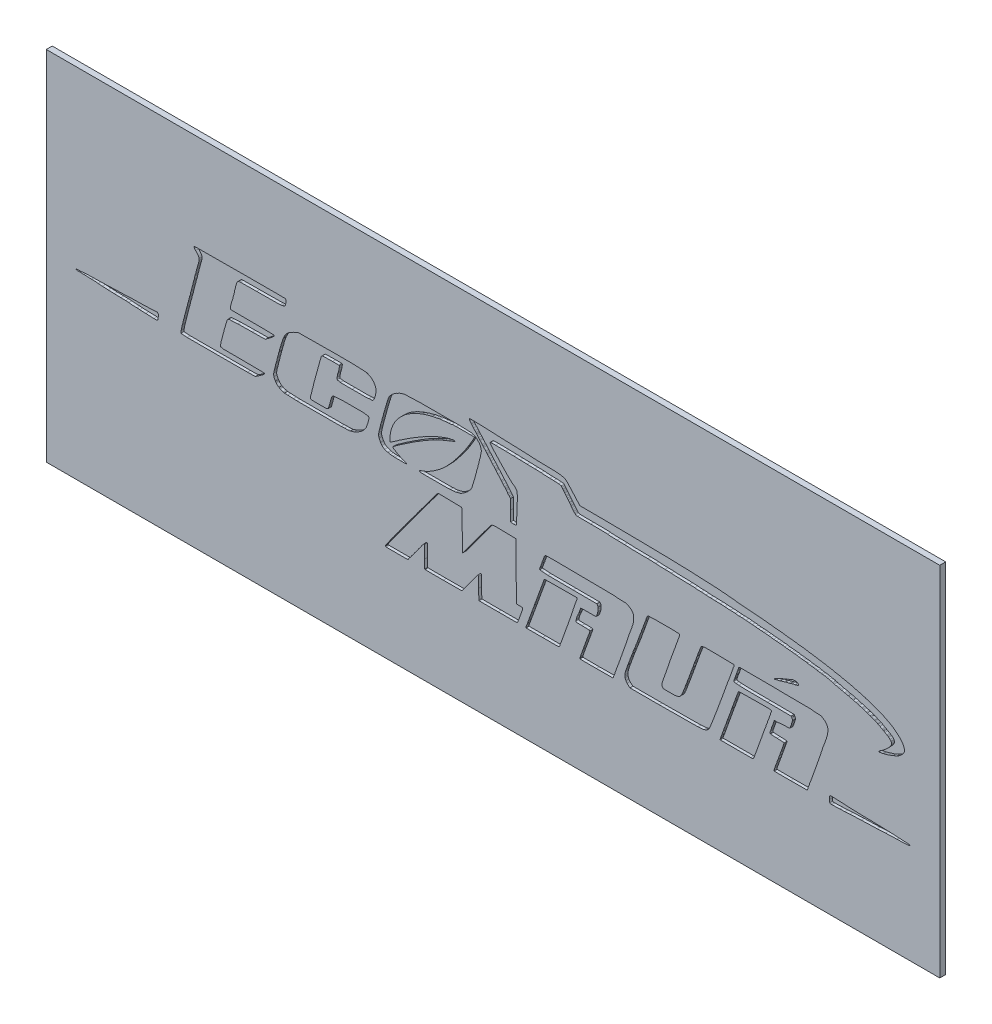
SolidWorks part; units mm, degrees
ref_plane "Front Plane" through (0, 0, 0) normal (0, 0, 1) x (1, 0, 0)
ref_plane "Top Plane" through (0, 0, 0) normal (0, 1, 0) x (1, 0, 0)
ref_plane "Right Plane" through (0, 0, 0) normal (1, 0, 0) x (0, 0, -1)
sketch "Model" plane through (0, 0, 0) normal (0, 0, 1) x (1, 0, 0)
  line L0 (-9.2909, -1.7034) -> (-9.2249, -1.6426)
  line L1 (-9.2249, -1.6426) -> (-8.9679, -1.6322)
  line L2 (16.2281, -9.015) -> (16.2584, -8.9291)
  line L3 (16.2584, -8.9291) -> (16.2249, -8.8956)
  line L4 (17.6532, -5.0267) -> (17.6542, -4.7462)
  line L5 (17.6542, -4.7462) -> (17.592, -4.6281)
  line L6 (17.4714, -4.4436) -> (17.4131, -4.3772)
  line L7 (17.4131, -4.3772) -> (13.4224, -4.3676)
  line L8 (-34.792, 13.3041) -> (-34.8002, 13.02)
  line L9 (-34.8002, 13.02) -> (-34.8591, 12.8967)
  line L10 (-45.4429, 1.3471) -> (-45.3207, 1.3081)
  line L11 (-45.3207, 1.3081) -> (-42.479, 1.2974)
  line L12 (-34.478, 0.0127) -> (-35.0168, 0.0219)
  line L13 (-35.0168, 0.0219) -> (-35.0935, 0.0622)
  line L14 (-23.6574, 6.2623) -> (-25.5986, 6.2677)
  line L15 (-25.5986, 6.2677) -> (-25.7241, 6.3011)
  line L16 (-25.8254, 8.6336) -> (-25.857, 8.6651)
  line L17 (-25.857, 8.6651) -> (-26.9457, 8.6647)
  line L18 (-29.2178, 1.3023) -> (-27.9584, 1.3062)
  line L19 (-27.9584, 1.3062) -> (-27.9001, 1.3448)
  spline S0 degree 3 poles (56.6925, -13.848) (56.6094, -13.8312) (56.5505, -13.7928) (56.5293, -13.7418) knots 0 0 0 0 1 1 1 1
  spline S1 degree 3 poles (56.5293, -13.7418) (56.5145, -13.7059) (56.5094, -13.5852) (56.5088, -13.2503) knots 0 0 0 0 1 1 1 1
  spline S2 degree 3 poles (56.5088, -13.2503) (56.5081, -12.8527) (56.5107, -12.8013) (56.534, -12.7586) knots 0 0 0 0 1 1 1 1
  spline S3 degree 3 poles (56.534, -12.7586) (56.5827, -12.6695) (56.6243, -12.6586) (56.9139, -12.6593) knots 0 0 0 0 1 1 1 1
  spline S4 degree 3 poles (56.9139, -12.6593) (57.1817, -12.66) (57.731, -12.6834) (58.1071, -12.71) knots 0 0 0 0 1 1 1 1
  spline S5 degree 3 poles (58.1071, -12.71) (58.2262, -12.7184) (58.5429, -12.7321) (58.8108, -12.7403) knots 0 0 0 0 1 1 1 1
  spline S6 degree 3 poles (58.8108, -12.7403) (59.3819, -12.7578) (59.6511, -12.7727) (60.1542, -12.8144) knots 0 0 0 0 1 1 1 1
  spline S7 degree 3 poles (60.1542, -12.8144) (60.4597, -12.8398) (60.7202, -12.8473) (61.6673, -12.8579) knots 0 0 0 0 1 1 1 1
  spline S8 degree 3 poles (61.6673, -12.8579) (62.2965, -12.865) (63.0505, -12.8778) (63.3428, -12.8863) knots 0 0 0 0 1 1 1 1
  spline S9 degree 3 poles (63.3428, -12.8863) (63.6351, -12.8948) (64.2031, -12.9085) (64.605, -12.9168) knots 0 0 0 0 1 1 1 1
  spline S10 degree 3 poles (64.605, -12.9168) (65.0069, -12.9251) (65.4519, -12.9386) (65.594, -12.9467) knots 0 0 0 0 1 1 1 1
  spline S11 degree 3 poles (65.594, -12.9467) (65.7361, -12.9548) (66.148, -12.9678) (66.5093, -12.9755) knots 0 0 0 0 1 1 1 1
  spline S12 degree 3 poles (66.5093, -12.9755) (66.8706, -12.9832) (67.2625, -12.9994) (67.3802, -13.0114) knots 0 0 0 0 1 1 1 1
  spline S13 degree 3 poles (67.3802, -13.0114) (67.9662, -13.0712) (68.3346, -13.0938) (68.7309, -13.0943) knots 0 0 0 0 1 1 1 1
  spline S14 degree 3 poles (68.7309, -13.0943) (69.3239, -13.0951) (69.8746, -13.1302) (69.9633, -13.1727) knots 0 0 0 0 1 1 1 1
  spline S15 degree 3 poles (69.9633, -13.1727) (70.0176, -13.1987) (70.0111, -13.2441) (69.9488, -13.2739) knots 0 0 0 0 1 1 1 1
  spline S16 degree 3 poles (69.9488, -13.2739) (69.9204, -13.2875) (69.8273, -13.3089) (69.742, -13.3213) knots 0 0 0 0 1 1 1 1
  spline S17 degree 3 poles (69.742, -13.3213) (69.3902, -13.3726) (69.0141, -13.3901) (67.7862, -13.4126) knots 0 0 0 0 1 1 1 1
  spline S18 degree 3 poles (67.7862, -13.4126) (66.5334, -13.4356) (66.3098, -13.444) (65.8819, -13.4846) knots 0 0 0 0 1 1 1 1
  spline S19 degree 3 poles (65.8819, -13.4846) (65.6395, -13.5076) (65.413, -13.5198) (64.5016, -13.5592) knots 0 0 0 0 1 1 1 1
  spline S20 degree 3 poles (64.5016, -13.5592) (62.993, -13.6244) (62.9511, -13.6257) (61.8075, -13.6407) knots 0 0 0 0 1 1 1 1
  spline S21 degree 3 poles (61.8075, -13.6407) (60.8386, -13.6534) (60.4858, -13.6684) (59.9328, -13.7205) knots 0 0 0 0 1 1 1 1
  spline S22 degree 3 poles (59.9328, -13.7205) (59.8029, -13.7327) (59.4242, -13.7562) (59.0913, -13.7728) knots 0 0 0 0 1 1 1 1
  spline S23 degree 3 poles (59.0913, -13.7728) (58.7584, -13.7893) (58.3665, -13.8097) (58.2204, -13.8181) knots 0 0 0 0 1 1 1 1
  spline S24 degree 3 poles (58.2204, -13.8181) (57.9069, -13.836) (57.0846, -13.8617) (56.8844, -13.8597) knots 0 0 0 0 1 1 1 1
  spline S25 degree 3 poles (56.8844, -13.8597) (56.8073, -13.859) (56.7209, -13.8537) (56.6925, -13.848) knots 0 0 0 0 1 1 1 1
  spline S26 degree 3 poles (-11.7897, -0.0867) (-12.0513, -0.0772) (-12.1919, -0.0577) (-12.263, -0.0212) knots 0 0 0 0 1 1 1 1
  spline S27 degree 3 poles (-12.263, -0.0212) (-12.3252, 0.0107) (-12.3388, 0.0771) (-12.2943, 0.1314) knots 0 0 0 0 1 1 1 1
  spline S28 degree 3 poles (-12.2943, 0.1314) (-12.2601, 0.1732) (-12.0331, 0.2572) (-11.8573, 0.2931) knots 0 0 0 0 1 1 1 1
  spline S29 degree 3 poles (-11.8573, 0.2931) (-11.7296, 0.3192) (-11.587, 0.3758) (-11.4019, 0.4739) knots 0 0 0 0 1 1 1 1
  spline S30 degree 3 poles (-11.4019, 0.4739) (-11.3718, 0.4898) (-11.3087, 0.5161) (-11.2617, 0.5323) knots 0 0 0 0 1 1 1 1
  spline S31 degree 3 poles (-11.2617, 0.5323) (-11.2146, 0.5484) (-11.1529, 0.5771) (-11.1244, 0.5958) knots 0 0 0 0 1 1 1 1
  spline S32 degree 3 poles (-11.1244, 0.5958) (-11.096, 0.6146) (-11.0484, 0.638) (-11.0186, 0.6478) knots 0 0 0 0 1 1 1 1
  spline S33 degree 3 poles (-11.0186, 0.6478) (-10.9888, 0.6576) (-10.9566, 0.675) (-10.9471, 0.6864) knots 0 0 0 0 1 1 1 1
  spline S34 degree 3 poles (-10.9471, 0.6864) (-10.9376, 0.6979) (-10.8926, 0.7212) (-10.8471, 0.7382) knots 0 0 0 0 1 1 1 1
  spline S35 degree 3 poles (-10.8471, 0.7382) (-10.8015, 0.7553) (-10.7341, 0.7908) (-10.6971, 0.8173) knots 0 0 0 0 1 1 1 1
  spline S36 degree 3 poles (-10.6971, 0.8173) (-10.6601, 0.8438) (-10.5515, 0.9048) (-10.4556, 0.953) knots 0 0 0 0 1 1 1 1
  spline S37 degree 3 poles (-10.4556, 0.953) (-10.3598, 1.0011) (-10.2469, 1.0694) (-10.2047, 1.1047) knots 0 0 0 0 1 1 1 1
  spline S38 degree 3 poles (-10.2047, 1.1047) (-10.1625, 1.14) (-10.0948, 1.1846) (-10.0542, 1.2037) knots 0 0 0 0 1 1 1 1
  spline S39 degree 3 poles (-10.0542, 1.2037) (-10.0136, 1.2229) (-9.9372, 1.2687) (-9.8844, 1.3056) knots 0 0 0 0 1 1 1 1
  spline S40 degree 3 poles (-9.8844, 1.3056) (-9.8316, 1.3425) (-9.7327, 1.4103) (-9.6645, 1.4562) knots 0 0 0 0 1 1 1 1
  spline S41 degree 3 poles (-9.6645, 1.4562) (-9.5964, 1.5022) (-9.5093, 1.5669) (-9.471, 1.6001) knots 0 0 0 0 1 1 1 1
  spline S42 degree 3 poles (-9.471, 1.6001) (-9.4327, 1.6334) (-9.3424, 1.6992) (-9.2702, 1.7464) knots 0 0 0 0 1 1 1 1
  spline S43 degree 3 poles (-9.2702, 1.7464) (-9.0751, 1.874) (-8.9989, 1.9316) (-8.8973, 2.0286) knots 0 0 0 0 1 1 1 1
  spline S44 degree 3 poles (-8.8973, 2.0286) (-8.8469, 2.0768) (-8.7876, 2.1272) (-8.7656, 2.1406) knots 0 0 0 0 1 1 1 1
  spline S45 degree 3 poles (-8.7656, 2.1406) (-8.7166, 2.1704) (-8.5317, 2.3269) (-8.3667, 2.4781) knots 0 0 0 0 1 1 1 1
  spline S46 degree 3 poles (-8.3667, 2.4781) (-8.2993, 2.5399) (-8.183, 2.6456) (-8.1084, 2.713) knots 0 0 0 0 1 1 1 1
  spline S47 degree 3 poles (-8.1084, 2.713) (-7.9449, 2.8605) (-7.9682, 2.8377) (-7.8287, 2.9857) knots 0 0 0 0 1 1 1 1
  spline S48 degree 3 poles (-7.8287, 2.9857) (-7.5545, 3.2767) (-7.4844, 3.3505) (-7.3703, 3.4689) knots 0 0 0 0 1 1 1 1
  spline S49 degree 3 poles (-7.3703, 3.4689) (-7.3038, 3.5379) (-7.2305, 3.6197) (-7.2075, 3.6506) knots 0 0 0 0 1 1 1 1
  spline S50 degree 3 poles (-7.2075, 3.6506) (-7.1844, 3.6815) (-7.1385, 3.7264) (-7.1054, 3.7504) knots 0 0 0 0 1 1 1 1
  spline S51 degree 3 poles (-7.1054, 3.7504) (-7.0723, 3.7744) (-7.0287, 3.8188) (-7.0085, 3.8492) knots 0 0 0 0 1 1 1 1
  spline S52 degree 3 poles (-7.0085, 3.8492) (-6.9883, 3.8795) (-6.9371, 3.9412) (-6.8947, 3.9862) knots 0 0 0 0 1 1 1 1
  spline S53 degree 3 poles (-6.8947, 3.9862) (-6.8523, 4.0312) (-6.8035, 4.0958) (-6.7862, 4.1297) knots 0 0 0 0 1 1 1 1
  spline S54 degree 3 poles (-6.7862, 4.1297) (-6.7689, 4.1635) (-6.7423, 4.1979) (-6.727, 4.2061) knots 0 0 0 0 1 1 1 1
  spline S55 degree 3 poles (-6.727, 4.2061) (-6.7118, 4.2142) (-6.667, 4.2618) (-6.6275, 4.3117) knots 0 0 0 0 1 1 1 1
  spline S56 degree 3 poles (-6.6275, 4.3117) (-6.5879, 4.3617) (-6.5117, 4.4532) (-6.458, 4.5151) knots 0 0 0 0 1 1 1 1
  spline S57 degree 3 poles (-6.458, 4.5151) (-6.4043, 4.577) (-6.3453, 4.6575) (-6.3268, 4.6938) knots 0 0 0 0 1 1 1 1
  spline S58 degree 3 poles (-6.3268, 4.6938) (-6.3083, 4.7302) (-6.2556, 4.8) (-6.2097, 4.8488) knots 0 0 0 0 1 1 1 1
  spline S59 degree 3 poles (-6.2097, 4.8488) (-6.1638, 4.8977) (-6.0972, 4.9776) (-6.0619, 5.0263) knots 0 0 0 0 1 1 1 1
  spline S60 degree 3 poles (-6.0619, 5.0263) (-6.0265, 5.075) (-5.9786, 5.1303) (-5.9555, 5.1491) knots 0 0 0 0 1 1 1 1
  spline S61 degree 3 poles (-5.9555, 5.1491) (-5.9324, 5.1679) (-5.8875, 5.2277) (-5.8557, 5.282) knots 0 0 0 0 1 1 1 1
  spline S62 degree 3 poles (-5.8557, 5.282) (-5.8238, 5.3362) (-5.7736, 5.4038) (-5.744, 5.4322) knots 0 0 0 0 1 1 1 1
  spline S63 degree 3 poles (-5.744, 5.4322) (-5.7143, 5.4607) (-5.671, 5.5238) (-5.6477, 5.5725) knots 0 0 0 0 1 1 1 1
  spline S64 degree 3 poles (-5.6477, 5.5725) (-5.6244, 5.6212) (-5.5601, 5.7154) (-5.5047, 5.7819) knots 0 0 0 0 1 1 1 1
  spline S65 degree 3 poles (-5.5047, 5.7819) (-5.3416, 5.9779) (-5.3184, 6.0081) (-5.2124, 6.163) knots 0 0 0 0 1 1 1 1
  spline S66 degree 3 poles (-5.2124, 6.163) (-5.1568, 6.2442) (-5.0767, 6.3538) (-5.0344, 6.4065) knots 0 0 0 0 1 1 1 1
  spline S67 degree 3 poles (-5.0344, 6.4065) (-4.9921, 6.4593) (-4.9441, 6.5291) (-4.9276, 6.5615) knots 0 0 0 0 1 1 1 1
  spline S68 degree 3 poles (-4.9276, 6.5615) (-4.9112, 6.594) (-4.8589, 6.6647) (-4.8114, 6.7186) knots 0 0 0 0 1 1 1 1
  spline S69 degree 3 poles (-4.8114, 6.7186) (-4.7218, 6.8202) (-4.5381, 7.1145) (-4.4919, 7.2305) knots 0 0 0 0 1 1 1 1
  spline S70 degree 3 poles (-4.4919, 7.2305) (-4.4773, 7.2671) (-4.4313, 7.3341) (-4.3898, 7.3795) knots 0 0 0 0 1 1 1 1
  spline S71 degree 3 poles (-4.3898, 7.3795) (-4.3482, 7.4249) (-4.2953, 7.5019) (-4.2722, 7.5506) knots 0 0 0 0 1 1 1 1
  spline S72 degree 3 poles (-4.2722, 7.5506) (-4.2491, 7.5993) (-4.1871, 7.6976) (-4.1344, 7.769) knots 0 0 0 0 1 1 1 1
  spline S73 degree 3 poles (-4.1344, 7.769) (-4.0817, 7.8404) (-4.0386, 7.9044) (-4.0386, 7.9112) knots 0 0 0 0 1 1 1 1
  spline S74 degree 3 poles (-4.0386, 7.9112) (-4.0386, 7.9181) (-4.0134, 7.9626) (-3.9825, 8.0102) knots 0 0 0 0 1 1 1 1
  spline S75 degree 3 poles (-3.9825, 8.0102) (-3.9516, 8.0578) (-3.9027, 8.1335) (-3.8738, 8.1784) knots 0 0 0 0 1 1 1 1
  spline S76 degree 3 poles (-3.8738, 8.1784) (-3.8233, 8.2569) (-3.7127, 8.4534) (-3.5884, 8.6859) knots 0 0 0 0 1 1 1 1
  spline S77 degree 3 poles (-3.5884, 8.6859) (-3.5559, 8.7466) (-3.4966, 8.8482) (-3.4567, 8.9115) knots 0 0 0 0 1 1 1 1
  spline S78 degree 3 poles (-3.4567, 8.9115) (-3.3869, 9.0222) (-3.3373, 9.1122) (-3.2144, 9.3508) knots 0 0 0 0 1 1 1 1
  spline S79 degree 3 poles (-3.2144, 9.3508) (-3.1833, 9.4112) (-3.1332, 9.4879) (-3.1032, 9.5211) knots 0 0 0 0 1 1 1 1
  spline S80 degree 3 poles (-3.1032, 9.5211) (-3.0732, 9.5543) (-3.0343, 9.6111) (-3.0167, 9.6474) knots 0 0 0 0 1 1 1 1
  spline S81 degree 3 poles (-3.0167, 9.6474) (-2.9969, 9.688) (-2.9748, 9.7132) (-2.9588, 9.7132) knots 0 0 0 0 1 1 1 1
  spline S82 degree 3 poles (-2.9588, 9.7132) (-2.9446, 9.7132) (-2.8925, 9.6784) (-2.8429, 9.6357) knots 0 0 0 0 1 1 1 1
  spline S83 degree 3 poles (-2.8429, 9.6357) (-2.7934, 9.5931) (-2.723, 9.5375) (-2.6866, 9.5122) knots 0 0 0 0 1 1 1 1
  spline S84 degree 3 poles (-2.6866, 9.5122) (-2.6502, 9.4869) (-2.5938, 9.4305) (-2.5612, 9.3868) knots 0 0 0 0 1 1 1 1
  spline S85 degree 3 poles (-2.5612, 9.3868) (-2.5286, 9.3431) (-2.4688, 9.2784) (-2.4282, 9.2429) knots 0 0 0 0 1 1 1 1
  spline S86 degree 3 poles (-2.4282, 9.2429) (-2.3877, 9.2075) (-2.3384, 9.1465) (-2.3185, 9.1074) knots 0 0 0 0 1 1 1 1
  spline S87 degree 3 poles (-2.3185, 9.1074) (-2.2987, 9.0683) (-2.2761, 9.0323) (-2.2682, 9.0274) knots 0 0 0 0 1 1 1 1
  spline S88 degree 3 poles (-2.2682, 9.0274) (-2.2603, 9.0226) (-2.2198, 8.9622) (-2.1782, 8.8932) knots 0 0 0 0 1 1 1 1
  spline S89 degree 3 poles (-2.1782, 8.8932) (-2.1046, 8.7714) (-2.0839, 8.7132) (-2, 8.392) knots 0 0 0 0 1 1 1 1
  spline S90 degree 3 poles (-2, 8.392) (-1.9575, 8.229) (-1.9585, 7.9807) (-2.0024, 7.8163) knots 0 0 0 0 1 1 1 1
  spline S91 degree 3 poles (-2.0024, 7.8163) (-2.0549, 7.6195) (-2.0725, 7.5284) (-2.0905, 7.3587) knots 0 0 0 0 1 1 1 1
  spline S92 degree 3 poles (-2.0905, 7.3587) (-2.1069, 7.2036) (-2.1385, 7.0824) (-2.2384, 6.7903) knots 0 0 0 0 1 1 1 1
  spline S93 degree 3 poles (-2.2384, 6.7903) (-2.2848, 6.6547) (-2.3173, 6.5098) (-2.333, 6.3696) knots 0 0 0 0 1 1 1 1
  spline S94 degree 3 poles (-2.333, 6.3696) (-2.3384, 6.3209) (-2.3632, 6.2146) (-2.388, 6.1334) knots 0 0 0 0 1 1 1 1
  spline S95 degree 3 poles (-2.388, 6.1334) (-2.4129, 6.0522) (-2.4556, 5.9127) (-2.483, 5.8234) knots 0 0 0 0 1 1 1 1
  spline S96 degree 3 poles (-2.483, 5.8234) (-2.5103, 5.7341) (-2.5426, 5.5913) (-2.5547, 5.506) knots 0 0 0 0 1 1 1 1
  spline S97 degree 3 poles (-2.5547, 5.506) (-2.5687, 5.4073) (-2.6038, 5.2707) (-2.6513, 5.1296) knots 0 0 0 0 1 1 1 1
  spline S98 degree 3 poles (-2.6513, 5.1296) (-2.7552, 4.8213) (-2.7676, 4.7762) (-2.7847, 4.6456) knots 0 0 0 0 1 1 1 1
  spline S99 degree 3 poles (-2.7847, 4.6456) (-2.7929, 4.5823) (-2.817, 4.4826) (-2.8382, 4.4241) knots 0 0 0 0 1 1 1 1
  spline S100 degree 3 poles (-2.8382, 4.4241) (-2.9176, 4.2043) (-2.9906, 3.9508) (-3.0123, 3.8191) knots 0 0 0 0 1 1 1 1
  spline S101 degree 3 poles (-3.0123, 3.8191) (-3.0356, 3.6779) (-3.1202, 3.398) (-3.1891, 3.2344) knots 0 0 0 0 1 1 1 1
  spline S102 degree 3 poles (-3.1891, 3.2344) (-3.2109, 3.1825) (-3.238, 3.0789) (-3.2492, 3.0042) knots 0 0 0 0 1 1 1 1
  spline S103 degree 3 poles (-3.2492, 3.0042) (-3.2704, 2.8627) (-3.344, 2.6282) (-3.407, 2.5016) knots 0 0 0 0 1 1 1 1
  spline S104 degree 3 poles (-3.407, 2.5016) (-3.4483, 2.4185) (-3.4692, 2.3426) (-3.4931, 2.189) knots 0 0 0 0 1 1 1 1
  spline S105 degree 3 poles (-3.4931, 2.189) (-3.5114, 2.071) (-3.5875, 1.8973) (-3.654, 1.8216) knots 0 0 0 0 1 1 1 1
  spline S106 degree 3 poles (-3.654, 1.8216) (-3.6772, 1.7951) (-3.7006, 1.7537) (-3.7059, 1.7295) knots 0 0 0 0 1 1 1 1
  spline S107 degree 3 poles (-3.7059, 1.7295) (-3.7144, 1.691) (-3.7809, 1.6106) (-4.1272, 1.2202) knots 0 0 0 0 1 1 1 1
  spline S108 degree 3 poles (-4.1272, 1.2202) (-4.287, 1.04) (-4.6454, 0.7314) (-4.7676, 0.6687) knots 0 0 0 0 1 1 1 1
  spline S109 degree 3 poles (-4.7676, 0.6687) (-4.7964, 0.654) (-4.865, 0.6031) (-4.9201, 0.5557) knots 0 0 0 0 1 1 1 1
  spline S110 degree 3 poles (-4.9201, 0.5557) (-4.9845, 0.5004) (-5.1074, 0.4232) (-5.264, 0.3397) knots 0 0 0 0 1 1 1 1
  spline S111 degree 3 poles (-5.264, 0.3397) (-5.4673, 0.2314) (-5.5253, 0.2071) (-5.614, 0.1934) knots 0 0 0 0 1 1 1 1
  spline S112 degree 3 poles (-5.614, 0.1934) (-5.6724, 0.1843) (-5.782, 0.1547) (-5.8574, 0.1276) knots 0 0 0 0 1 1 1 1
  spline S113 degree 3 poles (-5.8574, 0.1276) (-5.9329, 0.1004) (-6.036, 0.0703) (-6.0865, 0.0605) knots 0 0 0 0 1 1 1 1
  spline S114 degree 3 poles (-6.0865, 0.0605) (-6.1371, 0.0507) (-6.2168, 0.0291) (-6.2637, 0.0125) knots 0 0 0 0 1 1 1 1
  spline S115 degree 3 poles (-6.2637, 0.0125) (-6.3341, -0.0124) (-6.4068, -0.02) (-6.681, -0.0307) knots 0 0 0 0 1 1 1 1
  spline S116 degree 3 poles (-6.681, -0.0307) (-6.8637, -0.0378) (-7.0663, -0.0502) (-7.1313, -0.0581) knots 0 0 0 0 1 1 1 1
  spline S117 degree 3 poles (-7.1313, -0.0581) (-7.1962, -0.0661) (-7.3092, -0.0768) (-7.3822, -0.0819) knots 0 0 0 0 1 1 1 1
  spline S118 degree 3 poles (-7.3822, -0.0819) (-7.5612, -0.0944) (-11.4623, -0.0986) (-11.7897, -0.0867) knots 0 0 0 0 1 1 1 1
  spline S119 degree 3 poles (-56.9163, -0.0801) (-56.9856, -0.0638) (-57.6276, -0.0403) (-58.2966, -0.0296) knots 0 0 0 0 1 1 1 1
  spline S120 degree 3 poles (-58.2966, -0.0296) (-58.9287, -0.0195) (-59.1085, -0.0119) (-59.3152, 0.0133) knots 0 0 0 0 1 1 1 1
  spline S121 degree 3 poles (-59.3152, 0.0133) (-59.4576, 0.0308) (-59.6555, 0.0442) (-59.7728, 0.0443) knots 0 0 0 0 1 1 1 1
  spline S122 degree 3 poles (-59.7728, 0.0443) (-60.3012, 0.045) (-60.929, 0.0828) (-61.1678, 0.1283) knots 0 0 0 0 1 1 1 1
  spline S123 degree 3 poles (-61.1678, 0.1283) (-61.2666, 0.1471) (-61.3798, 0.1518) (-61.6993, 0.1502) knots 0 0 0 0 1 1 1 1
  spline S124 degree 3 poles (-61.6993, 0.1502) (-61.9225, 0.149) (-62.2746, 0.1578) (-62.4816, 0.1696) knots 0 0 0 0 1 1 1 1
  spline S125 degree 3 poles (-62.4816, 0.1696) (-62.6887, 0.1815) (-63.1836, 0.1948) (-63.5814, 0.1992) knots 0 0 0 0 1 1 1 1
  spline S126 degree 3 poles (-63.5814, 0.1992) (-64.1257, 0.2053) (-64.3833, 0.2144) (-64.6221, 0.2361) knots 0 0 0 0 1 1 1 1
  spline S127 degree 3 poles (-64.6221, 0.2361) (-64.7967, 0.2519) (-65.2218, 0.2745) (-65.5669, 0.2863) knots 0 0 0 0 1 1 1 1
  spline S128 degree 3 poles (-65.5669, 0.2863) (-66.0145, 0.3016) (-66.2239, 0.3144) (-66.2976, 0.3309) knots 0 0 0 0 1 1 1 1
  spline S129 degree 3 poles (-66.2976, 0.3309) (-66.5106, 0.3787) (-66.6569, 0.3874) (-67.4269, 0.3986) knots 0 0 0 0 1 1 1 1
  spline S130 degree 3 poles (-67.4269, 0.3986) (-67.9853, 0.4067) (-68.3464, 0.4193) (-68.6596, 0.4418) knots 0 0 0 0 1 1 1 1
  spline S131 degree 3 poles (-68.6596, 0.4418) (-69.0255, 0.4681) (-69.1678, 0.4719) (-69.4789, 0.4638) knots 0 0 0 0 1 1 1 1
  spline S132 degree 3 poles (-69.4789, 0.4638) (-69.8742, 0.4535) (-69.9666, 0.4624) (-69.994, 0.5137) knots 0 0 0 0 1 1 1 1
  spline S133 degree 3 poles (-69.994, 0.5137) (-70.0108, 0.5451) (-69.9922, 0.5827) (-69.9469, 0.6085) knots 0 0 0 0 1 1 1 1
  spline S134 degree 3 poles (-69.9469, 0.6085) (-69.9238, 0.6217) (-69.7857, 0.6297) (-69.4715, 0.636) knots 0 0 0 0 1 1 1 1
  spline S135 degree 3 poles (-69.4715, 0.636) (-69.1047, 0.6434) (-69.002, 0.6503) (-68.8736, 0.6761) knots 0 0 0 0 1 1 1 1
  spline S136 degree 3 poles (-68.8736, 0.6761) (-68.5776, 0.7356) (-68.483, 0.7406) (-67.3974, 0.7533) knots 0 0 0 0 1 1 1 1
  spline S137 degree 3 poles (-67.3974, 0.7533) (-66.8088, 0.7603) (-66.2076, 0.7726) (-66.0614, 0.7808) knots 0 0 0 0 1 1 1 1
  spline S138 degree 3 poles (-66.0614, 0.7808) (-65.2752, 0.8247) (-65.0556, 0.8319) (-64.5631, 0.8296) knots 0 0 0 0 1 1 1 1
  spline S139 degree 3 poles (-64.5631, 0.8296) (-64.0773, 0.8274) (-63.7141, 0.842) (-63.3305, 0.8792) knots 0 0 0 0 1 1 1 1
  spline S140 degree 3 poles (-63.3305, 0.8792) (-63.2817, 0.8839) (-62.8068, 0.8934) (-62.275, 0.9003) knots 0 0 0 0 1 1 1 1
  spline S141 degree 3 poles (-62.275, 0.9003) (-61.7115, 0.9076) (-61.2742, 0.9193) (-61.2269, 0.9284) knots 0 0 0 0 1 1 1 1
  spline S142 degree 3 poles (-61.2269, 0.9284) (-61.0487, 0.9628) (-60.7312, 0.9757) (-59.7064, 0.9902) knots 0 0 0 0 1 1 1 1
  spline S143 degree 3 poles (-59.7064, 0.9902) (-59.1177, 0.9985) (-58.5597, 1.0115) (-58.4664, 1.0189) knots 0 0 0 0 1 1 1 1
  spline S144 degree 3 poles (-58.4664, 1.0189) (-58.373, 1.0263) (-58.0143, 1.0389) (-57.6692, 1.0467) knots 0 0 0 0 1 1 1 1
  spline S145 degree 3 poles (-57.6692, 1.0467) (-57.3241, 1.0546) (-57.0076, 1.0675) (-56.9657, 1.0755) knots 0 0 0 0 1 1 1 1
  spline S146 degree 3 poles (-56.9657, 1.0755) (-56.9239, 1.0835) (-56.7872, 1.0983) (-56.6621, 1.1085) knots 0 0 0 0 1 1 1 1
  spline S147 degree 3 poles (-56.6621, 1.1085) (-56.4756, 1.1237) (-56.422, 1.1235) (-56.3652, 1.1076) knots 0 0 0 0 1 1 1 1
  spline S148 degree 3 poles (-56.3652, 1.1076) (-56.2764, 1.0828) (-56.2131, 1.0131) (-56.2006, 0.9267) knots 0 0 0 0 1 1 1 1
  spline S149 degree 3 poles (-56.2006, 0.9267) (-56.1865, 0.8284) (-56.2032, 0.221) (-56.2219, 0.1548) knots 0 0 0 0 1 1 1 1
  spline S150 degree 3 poles (-56.2219, 0.1548) (-56.2718, -0.0221) (-56.3047, -0.0516) (-56.4772, -0.074) knots 0 0 0 0 1 1 1 1
  spline S151 degree 3 poles (-56.4772, -0.074) (-56.5789, -0.0872) (-56.8692, -0.0913) (-56.9163, -0.0801) knots 0 0 0 0 1 1 1 1
  spline S152 degree 3 poles (-17.8928, -13.8178) (-17.9659, -13.8124) (-18.0414, -13.7994) (-18.0607, -13.7891) knots 0 0 0 0 1 1 1 1
  spline S153 degree 3 poles (-18.0607, -13.7891) (-18.0916, -13.7725) (-18.0948, -13.7625) (-18.0881, -13.7036) knots 0 0 0 0 1 1 1 1
  spline S154 degree 3 poles (-18.0881, -13.7036) (-18.084, -13.667) (-18.0666, -13.6195) (-18.0494, -13.5981) knots 0 0 0 0 1 1 1 1
  spline S155 degree 3 poles (-18.0494, -13.5981) (-18.0322, -13.5767) (-17.9675, -13.4844) (-17.9056, -13.3931) knots 0 0 0 0 1 1 1 1
  spline S156 degree 3 poles (-17.9056, -13.3931) (-17.8436, -13.3017) (-17.7886, -13.227) (-17.7833, -13.227) knots 0 0 0 0 1 1 1 1
  spline S157 degree 3 poles (-17.7833, -13.227) (-17.778, -13.227) (-17.7373, -13.1692) (-17.693, -13.0985) knots 0 0 0 0 1 1 1 1
  spline S158 degree 3 poles (-17.693, -13.0985) (-17.6486, -13.0278) (-17.5883, -12.9465) (-17.5589, -12.9177) knots 0 0 0 0 1 1 1 1
  spline S159 degree 3 poles (-17.5589, -12.9177) (-17.5296, -12.8889) (-17.4916, -12.8388) (-17.4746, -12.8063) knots 0 0 0 0 1 1 1 1
  spline S160 degree 3 poles (-17.4746, -12.8063) (-17.4474, -12.7543) (-17.4069, -12.6949) (-17.2581, -12.4889) knots 0 0 0 0 1 1 1 1
  spline S161 degree 3 poles (-17.2581, -12.4889) (-17.2376, -12.4605) (-17.188, -12.3941) (-17.1479, -12.3413) knots 0 0 0 0 1 1 1 1
  spline S162 degree 3 poles (-17.1479, -12.3413) (-17.1078, -12.2885) (-17.0368, -12.1889) (-16.99, -12.1199) knots 0 0 0 0 1 1 1 1
  spline S163 degree 3 poles (-16.99, -12.1199) (-16.9433, -12.0508) (-16.8815, -11.967) (-16.8527, -11.9335) knots 0 0 0 0 1 1 1 1
  spline S164 degree 3 poles (-16.8527, -11.9335) (-16.7554, -11.8201) (-16.7087, -11.7579) (-16.6768, -11.6989) knots 0 0 0 0 1 1 1 1
  spline S165 degree 3 poles (-16.6768, -11.6989) (-16.6594, -11.6665) (-16.6121, -11.6002) (-16.5717, -11.5515) knots 0 0 0 0 1 1 1 1
  spline S166 degree 3 poles (-16.5717, -11.5515) (-16.5314, -11.5028) (-16.4804, -11.433) (-16.4584, -11.3965) knots 0 0 0 0 1 1 1 1
  spline S167 degree 3 poles (-16.4584, -11.3965) (-16.4365, -11.36) (-16.3998, -11.3083) (-16.377, -11.2816) knots 0 0 0 0 1 1 1 1
  spline S168 degree 3 poles (-16.377, -11.2816) (-16.3541, -11.2549) (-16.3354, -11.2271) (-16.3354, -11.2198) knots 0 0 0 0 1 1 1 1
  spline S169 degree 3 poles (-16.3354, -11.2198) (-16.3354, -11.2124) (-16.3105, -11.1764) (-16.2801, -11.1397) knots 0 0 0 0 1 1 1 1
  spline S170 degree 3 poles (-16.2801, -11.1397) (-16.2496, -11.103) (-16.1981, -11.0346) (-16.1657, -10.9878) knots 0 0 0 0 1 1 1 1
  spline S171 degree 3 poles (-16.1657, -10.9878) (-16.1332, -10.9409) (-16.0792, -10.8725) (-16.0458, -10.8358) knots 0 0 0 0 1 1 1 1
  spline S172 degree 3 poles (-16.0458, -10.8358) (-16.0123, -10.7991) (-15.98, -10.7533) (-15.9741, -10.734) knots 0 0 0 0 1 1 1 1
  spline S173 degree 3 poles (-15.9741, -10.734) (-15.9681, -10.7147) (-15.9217, -10.6513) (-15.871, -10.5932) knots 0 0 0 0 1 1 1 1
  spline S174 degree 3 poles (-15.871, -10.5932) (-15.8204, -10.5351) (-15.7705, -10.4712) (-15.7601, -10.4512) knots 0 0 0 0 1 1 1 1
  spline S175 degree 3 poles (-15.7601, -10.4512) (-15.7293, -10.3914) (-15.6076, -10.2155) (-15.5971, -10.2155) knots 0 0 0 0 1 1 1 1
  spline S176 degree 3 poles (-15.5971, -10.2155) (-15.5917, -10.2155) (-15.542, -10.1475) (-15.4867, -10.0642) knots 0 0 0 0 1 1 1 1
  spline S177 degree 3 poles (-15.4867, -10.0642) (-15.4314, -9.981) (-15.3681, -9.893) (-15.346, -9.8686) knots 0 0 0 0 1 1 1 1
  spline S178 degree 3 poles (-15.346, -9.8686) (-15.3238, -9.8443) (-15.3032, -9.8161) (-15.3002, -9.806) knots 0 0 0 0 1 1 1 1
  spline S179 degree 3 poles (-15.3002, -9.806) (-15.2936, -9.784) (-15.2154, -9.6807) (-15.1286, -9.5793) knots 0 0 0 0 1 1 1 1
  spline S180 degree 3 poles (-15.1286, -9.5793) (-15.0941, -9.539) (-15.0659, -9.5005) (-15.0659, -9.4937) knots 0 0 0 0 1 1 1 1
  spline S181 degree 3 poles (-15.0659, -9.4937) (-15.0659, -9.4741) (-14.904, -9.2597) (-14.7765, -9.1104) knots 0 0 0 0 1 1 1 1
  spline S182 degree 3 poles (-14.7765, -9.1104) (-14.7512, -9.0809) (-14.7195, -9.0335) (-14.706, -9.0051) knots 0 0 0 0 1 1 1 1
  spline S183 degree 3 poles (-14.706, -9.0051) (-14.6926, -8.9766) (-14.6453, -8.9102) (-14.601, -8.8574) knots 0 0 0 0 1 1 1 1
  spline S184 degree 3 poles (-14.601, -8.8574) (-14.5568, -8.8047) (-14.5097, -8.7416) (-14.4963, -8.7172) knots 0 0 0 0 1 1 1 1
  spline S185 degree 3 poles (-14.4963, -8.7172) (-14.483, -8.6928) (-14.4551, -8.6548) (-14.4344, -8.6326) knots 0 0 0 0 1 1 1 1
  spline S186 degree 3 poles (-14.4344, -8.6326) (-14.4137, -8.6105) (-14.3829, -8.5699) (-14.3659, -8.5424) knots 0 0 0 0 1 1 1 1
  spline S187 degree 3 poles (-14.3659, -8.5424) (-14.3009, -8.4368) (-14.219, -8.3182) (-14.2044, -8.3086) knots 0 0 0 0 1 1 1 1
  spline S188 degree 3 poles (-14.2044, -8.3086) (-14.196, -8.3031) (-14.1643, -8.2632) (-14.1339, -8.22) knots 0 0 0 0 1 1 1 1
  spline S189 degree 3 poles (-14.1339, -8.22) (-14.0113, -8.046) (-13.9704, -7.9897) (-13.8995, -7.8979) knots 0 0 0 0 1 1 1 1
  spline S190 degree 3 poles (-13.8995, -7.8979) (-13.8587, -7.8451) (-13.8139, -7.7829) (-13.7998, -7.7595) knots 0 0 0 0 1 1 1 1
  spline S191 degree 3 poles (-13.7998, -7.7595) (-13.7857, -7.7362) (-13.7277, -7.6581) (-13.6709, -7.586) knots 0 0 0 0 1 1 1 1
  spline S192 degree 3 poles (-13.6709, -7.586) (-13.614, -7.514) (-13.5443, -7.4209) (-13.5159, -7.3792) knots 0 0 0 0 1 1 1 1
  spline S193 degree 3 poles (-13.5159, -7.3792) (-13.4875, -7.3375) (-13.441, -7.2768) (-13.4125, -7.2443) knots 0 0 0 0 1 1 1 1
  spline S194 degree 3 poles (-13.4125, -7.2443) (-13.3841, -7.2118) (-13.3476, -7.1631) (-13.3314, -7.1362) knots 0 0 0 0 1 1 1 1
  spline S195 degree 3 poles (-13.3314, -7.1362) (-13.2631, -7.023) (-13.1877, -6.9228) (-13.1596, -6.9078) knots 0 0 0 0 1 1 1 1
  spline S196 degree 3 poles (-13.1596, -6.9078) (-13.1431, -6.8989) (-13.1183, -6.8673) (-13.1045, -6.8375) knots 0 0 0 0 1 1 1 1
  spline S197 degree 3 poles (-13.1045, -6.8375) (-13.0764, -6.7766) (-13.0026, -6.6689) (-12.9254, -6.5762) knots 0 0 0 0 1 1 1 1
  spline S198 degree 3 poles (-12.9254, -6.5762) (-12.897, -6.5421) (-12.8622, -6.495) (-12.8481, -6.4716) knots 0 0 0 0 1 1 1 1
  spline S199 degree 3 poles (-12.8481, -6.4716) (-12.834, -6.4482) (-12.7925, -6.3892) (-12.7559, -6.3405) knots 0 0 0 0 1 1 1 1
  spline S200 degree 3 poles (-12.7559, -6.3405) (-12.7193, -6.2918) (-12.6777, -6.233) (-12.6635, -6.2099) knots 0 0 0 0 1 1 1 1
  spline S201 degree 3 poles (-12.6635, -6.2099) (-12.607, -6.1185) (-12.4984, -5.983) (-12.4631, -5.9598) knots 0 0 0 0 1 1 1 1
  spline S202 degree 3 poles (-12.4631, -5.9598) (-12.4425, -5.9463) (-12.4211, -5.9202) (-12.4155, -5.9017) knots 0 0 0 0 1 1 1 1
  spline S203 degree 3 poles (-12.4155, -5.9017) (-12.4099, -5.8832) (-12.3904, -5.8482) (-12.3723, -5.8238) knots 0 0 0 0 1 1 1 1
  spline S204 degree 3 poles (-12.3723, -5.8238) (-12.3541, -5.7995) (-12.3274, -5.7563) (-12.3128, -5.7279) knots 0 0 0 0 1 1 1 1
  spline S205 degree 3 poles (-12.3128, -5.7279) (-12.2982, -5.6995) (-12.2453, -5.6297) (-12.1951, -5.5729) knots 0 0 0 0 1 1 1 1
  spline S206 degree 3 poles (-12.1951, -5.5729) (-12.145, -5.516) (-12.0881, -5.443) (-12.0686, -5.4105) knots 0 0 0 0 1 1 1 1
  spline S207 degree 3 poles (-12.0686, -5.4105) (-12.0257, -5.3389) (-11.9731, -5.267) (-11.7289, -4.9465) knots 0 0 0 0 1 1 1 1
  spline S208 degree 3 poles (-11.7289, -4.9465) (-11.6644, -4.8618) (-11.6116, -4.7874) (-11.6116, -4.7813) knots 0 0 0 0 1 1 1 1
  spline S209 degree 3 poles (-11.6116, -4.7813) (-11.6116, -4.7752) (-11.5867, -4.7405) (-11.5562, -4.7042) knots 0 0 0 0 1 1 1 1
  spline S210 degree 3 poles (-11.5562, -4.7042) (-11.4755, -4.6081) (-11.4005, -4.511) (-11.302, -4.3754) knots 0 0 0 0 1 1 1 1
  spline S211 degree 3 poles (-11.302, -4.3754) (-11.2541, -4.3095) (-11.2044, -4.2515) (-11.1914, -4.2466) knots 0 0 0 0 1 1 1 1
  spline S212 degree 3 poles (-11.1914, -4.2466) (-11.1785, -4.2416) (-11.1548, -4.2069) (-11.1388, -4.1695) knots 0 0 0 0 1 1 1 1
  spline S213 degree 3 poles (-11.1388, -4.1695) (-11.1227, -4.1321) (-11.0648, -4.0458) (-11.01, -3.9778) knots 0 0 0 0 1 1 1 1
  spline S214 degree 3 poles (-11.01, -3.9778) (-10.9552, -3.9098) (-10.8906, -3.8224) (-10.8664, -3.7835) knots 0 0 0 0 1 1 1 1
  spline S215 degree 3 poles (-10.8664, -3.7835) (-10.8422, -3.7447) (-10.799, -3.6863) (-10.7702, -3.6538) knots 0 0 0 0 1 1 1 1
  spline S216 degree 3 poles (-10.7702, -3.6538) (-10.7415, -3.6213) (-10.6922, -3.5563) (-10.6606, -3.5092) knots 0 0 0 0 1 1 1 1
  spline S217 degree 3 poles (-10.6606, -3.5092) (-10.6291, -3.4622) (-10.5694, -3.3851) (-10.528, -3.3379) knots 0 0 0 0 1 1 1 1
  spline S218 degree 3 poles (-10.528, -3.3379) (-10.4866, -3.2907) (-10.4412, -3.2329) (-10.4272, -3.2094) knots 0 0 0 0 1 1 1 1
  spline S219 degree 3 poles (-10.4272, -3.2094) (-10.4131, -3.1859) (-10.3681, -3.1235) (-10.3273, -3.0707) knots 0 0 0 0 1 1 1 1
  spline S220 degree 3 poles (-10.3273, -3.0707) (-10.2864, -3.0179) (-10.2415, -2.956) (-10.2274, -2.9331) knots 0 0 0 0 1 1 1 1
  spline S221 degree 3 poles (-10.2274, -2.9331) (-10.185, -2.8641) (-10.0026, -2.6248) (-9.9415, -2.5581) knots 0 0 0 0 1 1 1 1
  spline S222 degree 3 poles (-9.9415, -2.5581) (-9.9101, -2.5237) (-9.8844, -2.4884) (-9.8844, -2.4795) knots 0 0 0 0 1 1 1 1
  spline S223 degree 3 poles (-9.8844, -2.4795) (-9.8844, -2.4706) (-9.8609, -2.4389) (-9.8322, -2.409) knots 0 0 0 0 1 1 1 1
  spline S224 degree 3 poles (-9.8322, -2.409) (-9.8034, -2.3792) (-9.7461, -2.3016) (-9.7047, -2.2367) knots 0 0 0 0 1 1 1 1
  spline S225 degree 3 poles (-9.7047, -2.2367) (-9.6633, -2.1717) (-9.6108, -2.0986) (-9.588, -2.0743) knots 0 0 0 0 1 1 1 1
  spline S226 degree 3 poles (-9.588, -2.0743) (-9.546, -2.0293) (-9.526, -2.003) (-9.4177, -1.8501) knots 0 0 0 0 1 1 1 1
  spline S227 degree 3 poles (-9.4177, -1.8501) (-9.3842, -1.8028) (-9.3272, -1.7369) (-9.2909, -1.7034) knots 0 0 0 0 1 1 1 1
  spline S228 degree 3 poles (-8.9679, -1.6322) (-8.7258, -1.6224) (-8.0925, -1.6342) (-6.9911, -1.6692) knots 0 0 0 0 1 1 1 1
  spline S229 degree 3 poles (-6.9911, -1.6692) (-6.7272, -1.6775) (-6.2428, -1.6902) (-5.9147, -1.6974) knots 0 0 0 0 1 1 1 1
  spline S230 degree 3 poles (-5.9147, -1.6974) (-5.3597, -1.7095) (-5.3155, -1.7124) (-5.2799, -1.7389) knots 0 0 0 0 1 1 1 1
  spline S231 degree 3 poles (-5.2799, -1.7389) (-5.2552, -1.7574) (-5.2384, -1.7877) (-5.2322, -1.8249) knots 0 0 0 0 1 1 1 1
  spline S232 degree 3 poles (-5.2322, -1.8249) (-5.2269, -1.8565) (-5.2183, -2.3042) (-5.213, -2.8198) knots 0 0 0 0 1 1 1 1
  spline S233 degree 3 poles (-5.213, -2.8198) (-5.2039, -3.7063) (-5.1981, -3.9926) (-5.1598, -5.4326) knots 0 0 0 0 1 1 1 1
  spline S234 degree 3 poles (-5.1598, -5.4326) (-5.1511, -5.7615) (-5.1392, -6.5088) (-5.1335, -7.0934) knots 0 0 0 0 1 1 1 1
  spline S235 degree 3 poles (-5.1335, -7.0934) (-5.123, -8.1486) (-5.1191, -8.2227) (-5.0743, -8.2227) knots 0 0 0 0 1 1 1 1
  spline S236 degree 3 poles (-5.0743, -8.2227) (-5.068, -8.2227) (-5.0418, -8.1944) (-5.0159, -8.1599) knots 0 0 0 0 1 1 1 1
  spline S237 degree 3 poles (-5.0159, -8.1599) (-4.9901, -8.1254) (-4.9207, -8.0328) (-4.8617, -7.9541) knots 0 0 0 0 1 1 1 1
  spline S238 degree 3 poles (-4.8617, -7.9541) (-4.8028, -7.8755) (-4.7131, -7.7568) (-4.6623, -7.6904) knots 0 0 0 0 1 1 1 1
  spline S239 degree 3 poles (-4.6623, -7.6904) (-4.6116, -7.624) (-4.5701, -7.5607) (-4.5701, -7.5498) knots 0 0 0 0 1 1 1 1
  spline S240 degree 3 poles (-4.5701, -7.5498) (-4.5701, -7.5388) (-4.5202, -7.4727) (-4.4594, -7.4029) knots 0 0 0 0 1 1 1 1
  spline S241 degree 3 poles (-4.4594, -7.4029) (-4.3985, -7.3331) (-4.3486, -7.2706) (-4.3486, -7.2642) knots 0 0 0 0 1 1 1 1
  spline S242 degree 3 poles (-4.3486, -7.2642) (-4.3486, -7.2535) (-4.2644, -7.1321) (-4.1636, -6.9974) knots 0 0 0 0 1 1 1 1
  spline S243 degree 3 poles (-4.1636, -6.9974) (-4.1423, -6.969) (-4.0918, -6.8993) (-4.0512, -6.8424) knots 0 0 0 0 1 1 1 1
  spline S244 degree 3 poles (-4.0512, -6.8424) (-4.0107, -6.7856) (-3.9591, -6.7192) (-3.9367, -6.6948) knots 0 0 0 0 1 1 1 1
  spline S245 degree 3 poles (-3.9367, -6.6948) (-3.9142, -6.6704) (-3.877, -6.6175) (-3.854, -6.5771) knots 0 0 0 0 1 1 1 1
  spline S246 degree 3 poles (-3.854, -6.5771) (-3.831, -6.5368) (-3.781, -6.4737) (-3.7429, -6.4369) knots 0 0 0 0 1 1 1 1
  spline S247 degree 3 poles (-3.7429, -6.4369) (-3.7048, -6.4001) (-3.6634, -6.3501) (-3.651, -6.3257) knots 0 0 0 0 1 1 1 1
  spline S248 degree 3 poles (-3.651, -6.3257) (-3.6183, -6.2618) (-3.5273, -6.129) (-3.4729, -6.0657) knots 0 0 0 0 1 1 1 1
  spline S249 degree 3 poles (-3.4729, -6.0657) (-3.4254, -6.0106) (-3.3813, -5.9481) (-3.3339, -5.869) knots 0 0 0 0 1 1 1 1
  spline S250 degree 3 poles (-3.3339, -5.869) (-3.3196, -5.8451) (-3.2806, -5.7953) (-3.2472, -5.7583) knots 0 0 0 0 1 1 1 1
  spline S251 degree 3 poles (-3.2472, -5.7583) (-3.2139, -5.7213) (-3.1779, -5.6744) (-3.1674, -5.6541) knots 0 0 0 0 1 1 1 1
  spline S252 degree 3 poles (-3.1674, -5.6541) (-3.1469, -5.6146) (-3.031, -5.4574) (-2.9333, -5.3367) knots 0 0 0 0 1 1 1 1
  spline S253 degree 3 poles (-2.9333, -5.3367) (-2.9004, -5.2961) (-2.863, -5.2396) (-2.8501, -5.2112) knots 0 0 0 0 1 1 1 1
  spline S254 degree 3 poles (-2.8501, -5.2112) (-2.8373, -5.1828) (-2.8015, -5.133) (-2.7707, -5.1005) knots 0 0 0 0 1 1 1 1
  spline S255 degree 3 poles (-2.7707, -5.1005) (-2.7398, -5.068) (-2.6925, -5.0082) (-2.6655, -4.9676) knots 0 0 0 0 1 1 1 1
  spline S256 degree 3 poles (-2.6655, -4.9676) (-2.6048, -4.8763) (-2.5903, -4.8564) (-2.487, -4.7215) knots 0 0 0 0 1 1 1 1
  spline S257 degree 3 poles (-2.487, -4.7215) (-2.4414, -4.662) (-2.3865, -4.5851) (-2.365, -4.5506) knots 0 0 0 0 1 1 1 1
  spline S258 degree 3 poles (-2.365, -4.5506) (-2.3435, -4.5161) (-2.3199, -4.4879) (-2.3126, -4.4879) knots 0 0 0 0 1 1 1 1
  spline S259 degree 3 poles (-2.3126, -4.4879) (-2.3002, -4.4879) (-2.2449, -4.4093) (-2.1684, -4.283) knots 0 0 0 0 1 1 1 1
  spline S260 degree 3 poles (-2.1684, -4.283) (-2.1506, -4.2536) (-2.1047, -4.193) (-2.0664, -4.1483) knots 0 0 0 0 1 1 1 1
  spline S261 degree 3 poles (-2.0664, -4.1483) (-2.0282, -4.1037) (-1.9687, -4.024) (-1.9343, -3.9712) knots 0 0 0 0 1 1 1 1
  spline S262 degree 3 poles (-1.9343, -3.9712) (-1.8999, -3.9184) (-1.8312, -3.8301) (-1.7816, -3.7749) knots 0 0 0 0 1 1 1 1
  spline S263 degree 3 poles (-1.7816, -3.7749) (-1.732, -3.7197) (-1.6915, -3.6682) (-1.6915, -3.6605) knots 0 0 0 0 1 1 1 1
  spline S264 degree 3 poles (-1.6915, -3.6605) (-1.6915, -3.6528) (-1.6691, -3.6216) (-1.6418, -3.5911) knots 0 0 0 0 1 1 1 1
  spline S265 degree 3 poles (-1.6418, -3.5911) (-1.6145, -3.5606) (-1.582, -3.5158) (-1.5695, -3.4914) knots 0 0 0 0 1 1 1 1
  spline S266 degree 3 poles (-1.5695, -3.4914) (-1.5571, -3.467) (-1.5324, -3.4339) (-1.5146, -3.4179) knots 0 0 0 0 1 1 1 1
  spline S267 degree 3 poles (-1.5146, -3.4179) (-1.4969, -3.4018) (-1.4732, -3.3667) (-1.4619, -3.3398) knots 0 0 0 0 1 1 1 1
  spline S268 degree 3 poles (-1.4619, -3.3398) (-1.4426, -3.2935) (-1.3979, -3.2346) (-1.2764, -3.0951) knots 0 0 0 0 1 1 1 1
  spline S269 degree 3 poles (-1.2764, -3.0951) (-1.2471, -3.0614) (-1.2113, -3.0107) (-1.1968, -2.9826) knots 0 0 0 0 1 1 1 1
  spline S270 degree 3 poles (-1.1968, -2.9826) (-1.1824, -2.9544) (-1.1359, -2.8946) (-1.0934, -2.8497) knots 0 0 0 0 1 1 1 1
  spline S271 degree 3 poles (-1.0934, -2.8497) (-1.0509, -2.8048) (-1.0049, -2.746) (-0.9912, -2.719) knots 0 0 0 0 1 1 1 1
  spline S272 degree 3 poles (-0.9912, -2.719) (-0.9676, -2.6726) (-0.9076, -2.5876) (-0.828, -2.4876) knots 0 0 0 0 1 1 1 1
  spline S273 degree 3 poles (-0.828, -2.4876) (-0.8086, -2.4633) (-0.7597, -2.3968) (-0.7194, -2.34) knots 0 0 0 0 1 1 1 1
  spline S274 degree 3 poles (-0.7194, -2.34) (-0.679, -2.2832) (-0.6232, -2.2101) (-0.5955, -2.1776) knots 0 0 0 0 1 1 1 1
  spline S275 degree 3 poles (-0.5955, -2.1776) (-0.5677, -2.1451) (-0.5247, -2.0887) (-0.4998, -2.0521) knots 0 0 0 0 1 1 1 1
  spline S276 degree 3 poles (-0.4998, -2.0521) (-0.4527, -1.9828) (-0.2903, -1.8209) (-0.1991, -1.7524) knots 0 0 0 0 1 1 1 1
  spline S277 degree 3 poles (-0.1991, -1.7524) (-0.1603, -1.7233) (-0.1285, -1.7126) (-0.081, -1.7124) knots 0 0 0 0 1 1 1 1
  spline S278 degree 3 poles (-0.081, -1.7124) (-0.0452, -1.7123) (0.0372, -1.6987) (0.1021, -1.6821) knots 0 0 0 0 1 1 1 1
  spline S279 degree 3 poles (0.1021, -1.6821) (0.1977, -1.6577) (0.2863, -1.6504) (0.5671, -1.6436) knots 0 0 0 0 1 1 1 1
  spline S280 degree 3 poles (0.5671, -1.6436) (0.9119, -1.6353) (1.8508, -1.654) (2.6412, -1.6849) knots 0 0 0 0 1 1 1 1
  spline S281 degree 3 poles (2.6412, -1.6849) (2.8685, -1.6939) (3.2173, -1.7021) (3.4162, -1.7033) knots 0 0 0 0 1 1 1 1
  spline S282 degree 3 poles (3.4162, -1.7033) (3.7912, -1.7056) (3.8327, -1.7119) (3.8508, -1.7689) knots 0 0 0 0 1 1 1 1
  spline S283 degree 3 poles (3.8508, -1.7689) (3.8555, -1.7837) (3.8657, -3.2003) (3.8735, -4.9169) knots 0 0 0 0 1 1 1 1
  spline S284 degree 3 poles (3.8735, -4.9169) (3.8881, -8.115) (3.9126, -10.9838) (3.9261, -11.0666) knots 0 0 0 0 1 1 1 1
  spline S285 degree 3 poles (3.9261, -11.0666) (3.94, -11.1518) (3.9424, -11.1522) (4.4186, -11.1607) knots 0 0 0 0 1 1 1 1
  spline S286 degree 3 poles (4.4186, -11.1607) (4.885, -11.169) (4.9181, -11.1742) (4.9498, -11.2438) knots 0 0 0 0 1 1 1 1
  spline S287 degree 3 poles (4.9498, -11.2438) (4.9588, -11.2636) (4.9662, -11.3058) (4.9662, -11.3375) knots 0 0 0 0 1 1 1 1
  spline S288 degree 3 poles (4.9662, -11.3375) (4.9662, -11.419) (4.8999, -11.6532) (4.8471, -11.7582) knots 0 0 0 0 1 1 1 1
  spline S289 degree 3 poles (4.8471, -11.7582) (4.8226, -11.8069) (4.7931, -11.88) (4.7816, -11.9206) knots 0 0 0 0 1 1 1 1
  spline S290 degree 3 poles (4.7816, -11.9206) (4.7701, -11.9612) (4.7407, -12.0508) (4.7164, -12.1199) knots 0 0 0 0 1 1 1 1
  spline S291 degree 3 poles (4.7164, -12.1199) (4.6921, -12.1889) (4.6719, -12.2596) (4.6716, -12.277) knots 0 0 0 0 1 1 1 1
  spline S292 degree 3 poles (4.6716, -12.277) (4.6713, -12.2945) (4.651, -12.3467) (4.6266, -12.3931) knots 0 0 0 0 1 1 1 1
  spline S293 degree 3 poles (4.6266, -12.3931) (4.6023, -12.4394) (4.5716, -12.5148) (4.5586, -12.5606) knots 0 0 0 0 1 1 1 1
  spline S294 degree 3 poles (4.5586, -12.5606) (4.5455, -12.6064) (4.5231, -12.6638) (4.5087, -12.6882) knots 0 0 0 0 1 1 1 1
  spline S295 degree 3 poles (4.5087, -12.6882) (4.4944, -12.7126) (4.4712, -12.7856) (4.4572, -12.8506) knots 0 0 0 0 1 1 1 1
  spline S296 degree 3 poles (4.4572, -12.8506) (4.4433, -12.9155) (4.4132, -13.0019) (4.3903, -13.0425) knots 0 0 0 0 1 1 1 1
  spline S297 degree 3 poles (4.3903, -13.0425) (4.3675, -13.0831) (4.341, -13.1461) (4.3313, -13.1825) knots 0 0 0 0 1 1 1 1
  spline S298 degree 3 poles (4.3313, -13.1825) (4.3216, -13.2189) (4.298, -13.2796) (4.2789, -13.3174) knots 0 0 0 0 1 1 1 1
  spline S299 degree 3 poles (4.2789, -13.3174) (4.2597, -13.3552) (4.2328, -13.4317) (4.2191, -13.4874) knots 0 0 0 0 1 1 1 1
  spline S300 degree 3 poles (4.2191, -13.4874) (4.1895, -13.6072) (4.0922, -13.8098) (4.0579, -13.823) knots 0 0 0 0 1 1 1 1
  spline S301 degree 3 poles (4.0579, -13.823) (4.0447, -13.8281) (2.6097, -13.8323) (0.8692, -13.8323) knots 0 0 0 0 1 1 1 1
  spline S302 degree 3 poles (0.8692, -13.8323) (-1.5074, -13.8323) (-2.3047, -13.828) (-2.3331, -13.8151) knots 0 0 0 0 1 1 1 1
  spline S303 degree 3 poles (-2.3331, -13.8151) (-2.3577, -13.8038) (-2.3756, -13.7795) (-2.3847, -13.7449) knots 0 0 0 0 1 1 1 1
  spline S304 degree 3 poles (-2.3847, -13.7449) (-2.3924, -13.7153) (-2.4054, -12.9714) (-2.4141, -12.0534) knots 0 0 0 0 1 1 1 1
  spline S305 degree 3 poles (-2.4141, -12.0534) (-2.4232, -11.0845) (-2.4358, -10.3756) (-2.4448, -10.3189) knots 0 0 0 0 1 1 1 1
  spline S306 degree 3 poles (-2.4448, -10.3189) (-2.4601, -10.2221) (-2.4987, -10.1642) (-2.5373, -10.18) knots 0 0 0 0 1 1 1 1
  spline S307 degree 3 poles (-2.5373, -10.18) (-2.5471, -10.184) (-2.5731, -10.2153) (-2.5952, -10.2494) knots 0 0 0 0 1 1 1 1
  spline S308 degree 3 poles (-2.5952, -10.2494) (-2.6173, -10.2836) (-2.6687, -10.3514) (-2.7095, -10.4001) knots 0 0 0 0 1 1 1 1
  spline S309 degree 3 poles (-2.7095, -10.4001) (-2.7502, -10.4488) (-2.7964, -10.5124) (-2.8122, -10.5415) knots 0 0 0 0 1 1 1 1
  spline S310 degree 3 poles (-2.8122, -10.5415) (-2.828, -10.5706) (-2.8816, -10.643) (-2.9313, -10.7025) knots 0 0 0 0 1 1 1 1
  spline S311 degree 3 poles (-2.9313, -10.7025) (-2.981, -10.762) (-3.0317, -10.8301) (-3.044, -10.8538) knots 0 0 0 0 1 1 1 1
  spline S312 degree 3 poles (-3.044, -10.8538) (-3.0685, -10.9011) (-3.1449, -11.006) (-3.2136, -11.0865) knots 0 0 0 0 1 1 1 1
  spline S313 degree 3 poles (-3.2136, -11.0865) (-3.2379, -11.1149) (-3.2947, -11.1946) (-3.34, -11.2637) knots 0 0 0 0 1 1 1 1
  spline S314 degree 3 poles (-3.34, -11.2637) (-3.3853, -11.3327) (-3.4381, -11.4044) (-3.4574, -11.423) knots 0 0 0 0 1 1 1 1
  spline S315 degree 3 poles (-3.4574, -11.423) (-3.4767, -11.4416) (-3.5058, -11.4814) (-3.5222, -11.5115) knots 0 0 0 0 1 1 1 1
  spline S316 degree 3 poles (-3.5222, -11.5115) (-3.5385, -11.5416) (-3.5849, -11.6061) (-3.6252, -11.6548) knots 0 0 0 0 1 1 1 1
  spline S317 degree 3 poles (-3.6252, -11.6548) (-3.6656, -11.7036) (-3.7168, -11.7733) (-3.739, -11.8099) knots 0 0 0 0 1 1 1 1
  spline S318 degree 3 poles (-3.739, -11.8099) (-3.7876, -11.8896) (-3.9014, -12.0416) (-3.9221, -12.0544) knots 0 0 0 0 1 1 1 1
  spline S319 degree 3 poles (-3.9221, -12.0544) (-3.9302, -12.0594) (-3.9726, -12.1189) (-4.0163, -12.1867) knots 0 0 0 0 1 1 1 1
  spline S320 degree 3 poles (-4.0163, -12.1867) (-4.06, -12.2544) (-4.1123, -12.3206) (-4.1324, -12.3338) knots 0 0 0 0 1 1 1 1
  spline S321 degree 3 poles (-4.1324, -12.3338) (-4.1525, -12.347) (-4.1788, -12.3823) (-4.1908, -12.4123) knots 0 0 0 0 1 1 1 1
  spline S322 degree 3 poles (-4.1908, -12.4123) (-4.2028, -12.4422) (-4.2273, -12.48) (-4.2453, -12.4963) knots 0 0 0 0 1 1 1 1
  spline S323 degree 3 poles (-4.2453, -12.4963) (-4.2633, -12.5125) (-4.2908, -12.551) (-4.3066, -12.5818) knots 0 0 0 0 1 1 1 1
  spline S324 degree 3 poles (-4.3066, -12.5818) (-4.3223, -12.6126) (-4.3521, -12.6525) (-4.3729, -12.6704) knots 0 0 0 0 1 1 1 1
  spline S325 degree 3 poles (-4.3729, -12.6704) (-4.3936, -12.6883) (-4.424, -12.7295) (-4.4403, -12.762) knots 0 0 0 0 1 1 1 1
  spline S326 degree 3 poles (-4.4403, -12.762) (-4.4567, -12.7945) (-4.4821, -12.8343) (-4.4968, -12.8506) knots 0 0 0 0 1 1 1 1
  spline S327 degree 3 poles (-4.4968, -12.8506) (-4.5274, -12.8845) (-4.5866, -12.968) (-4.7233, -13.1704) knots 0 0 0 0 1 1 1 1
  spline S328 degree 3 poles (-4.7233, -13.1704) (-4.7763, -13.2488) (-4.8268, -13.3174) (-4.8355, -13.3228) knots 0 0 0 0 1 1 1 1
  spline S329 degree 3 poles (-4.8355, -13.3228) (-4.8517, -13.3328) (-4.9421, -13.4487) (-5.0203, -13.5597) knots 0 0 0 0 1 1 1 1
  spline S330 degree 3 poles (-5.0203, -13.5597) (-5.1268, -13.7107) (-5.1936, -13.789) (-5.2339, -13.8099) knots 0 0 0 0 1 1 1 1
  spline S331 degree 3 poles (-5.2339, -13.8099) (-5.2722, -13.8297) (-5.6306, -13.8323) (-8.3194, -13.8323) knots 0 0 0 0 1 1 1 1
  spline S332 degree 3 poles (-8.3194, -13.8323) (-10.9122, -13.8323) (-11.369, -13.8292) (-11.4117, -13.8113) knots 0 0 0 0 1 1 1 1
  spline S333 degree 3 poles (-11.4117, -13.8113) (-11.4551, -13.7932) (-11.4629, -13.7818) (-11.4704, -13.7264) knots 0 0 0 0 1 1 1 1
  spline S334 degree 3 poles (-11.4704, -13.7264) (-11.4751, -13.6913) (-11.4861, -13.0679) (-11.4947, -12.3413) knots 0 0 0 0 1 1 1 1
  spline S335 degree 3 poles (-11.4947, -12.3413) (-11.5147, -10.666) (-11.5254, -10.2704) (-11.5513, -10.2391) knots 0 0 0 0 1 1 1 1
  spline S336 degree 3 poles (-11.5513, -10.2391) (-11.5621, -10.2262) (-11.5899, -10.2155) (-11.6132, -10.2155) knots 0 0 0 0 1 1 1 1
  spline S337 degree 3 poles (-11.6132, -10.2155) (-11.6465, -10.2155) (-11.6634, -10.2281) (-11.6931, -10.2751) knots 0 0 0 0 1 1 1 1
  spline S338 degree 3 poles (-11.6931, -10.2751) (-11.7481, -10.3623) (-11.863, -10.5108) (-11.8753, -10.5108) knots 0 0 0 0 1 1 1 1
  spline S339 degree 3 poles (-11.8753, -10.5108) (-11.8812, -10.5108) (-11.9223, -10.5678) (-11.9665, -10.6375) knots 0 0 0 0 1 1 1 1
  spline S340 degree 3 poles (-11.9665, -10.6375) (-12.0108, -10.7072) (-12.0672, -10.7886) (-12.0919, -10.8183) knots 0 0 0 0 1 1 1 1
  spline S341 degree 3 poles (-12.0919, -10.8183) (-12.1165, -10.8481) (-12.1548, -10.899) (-12.177, -10.9315) knots 0 0 0 0 1 1 1 1
  spline S342 degree 3 poles (-12.177, -10.9315) (-12.1991, -10.964) (-12.2468, -11.0304) (-12.2829, -11.0791) knots 0 0 0 0 1 1 1 1
  spline S343 degree 3 poles (-12.2829, -11.0791) (-12.319, -11.1278) (-12.3601, -11.1843) (-12.3743, -11.2046) knots 0 0 0 0 1 1 1 1
  spline S344 degree 3 poles (-12.3743, -11.2046) (-12.3884, -11.2249) (-12.4202, -11.2653) (-12.445, -11.2944) knots 0 0 0 0 1 1 1 1
  spline S345 degree 3 poles (-12.445, -11.2944) (-12.4697, -11.3235) (-12.5015, -11.3667) (-12.5157, -11.3904) knots 0 0 0 0 1 1 1 1
  spline S346 degree 3 poles (-12.5157, -11.3904) (-12.5299, -11.4141) (-12.5717, -11.4733) (-12.6086, -11.522) knots 0 0 0 0 1 1 1 1
  spline S347 degree 3 poles (-12.6086, -11.522) (-12.6455, -11.5707) (-12.7046, -11.6537) (-12.7398, -11.7065) knots 0 0 0 0 1 1 1 1
  spline S348 degree 3 poles (-12.7398, -11.7065) (-12.7751, -11.7593) (-12.8349, -11.8383) (-12.8728, -11.8821) knots 0 0 0 0 1 1 1 1
  spline S349 degree 3 poles (-12.8728, -11.8821) (-12.9107, -11.9259) (-12.9542, -11.9861) (-12.9694, -12.0159) knots 0 0 0 0 1 1 1 1
  spline S350 degree 3 poles (-12.9694, -12.0159) (-12.9846, -12.0458) (-13.0072, -12.0786) (-13.0196, -12.0889) knots 0 0 0 0 1 1 1 1
  spline S351 degree 3 poles (-13.0196, -12.0889) (-13.032, -12.0992) (-13.0589, -12.1361) (-13.0793, -12.171) knots 0 0 0 0 1 1 1 1
  spline S352 degree 3 poles (-13.0793, -12.171) (-13.0998, -12.2059) (-13.1252, -12.2378) (-13.1358, -12.2419) knots 0 0 0 0 1 1 1 1
  spline S353 degree 3 poles (-13.1358, -12.2419) (-13.1464, -12.2459) (-13.1743, -12.2849) (-13.1979, -12.3285) knots 0 0 0 0 1 1 1 1
  spline S354 degree 3 poles (-13.1979, -12.3285) (-13.2214, -12.3721) (-13.2556, -12.4243) (-13.2738, -12.4446) knots 0 0 0 0 1 1 1 1
  spline S355 degree 3 poles (-13.2738, -12.4446) (-13.3575, -12.5381) (-13.4241, -12.6257) (-13.4715, -12.7052) knots 0 0 0 0 1 1 1 1
  spline S356 degree 3 poles (-13.4715, -12.7052) (-13.4999, -12.7527) (-13.5505, -12.8214) (-13.5839, -12.858) knots 0 0 0 0 1 1 1 1
  spline S357 degree 3 poles (-13.5839, -12.858) (-13.6173, -12.8945) (-13.6532, -12.941) (-13.6638, -12.9613) knots 0 0 0 0 1 1 1 1
  spline S358 degree 3 poles (-13.6638, -12.9613) (-13.6743, -12.9816) (-13.7201, -13.0468) (-13.7655, -13.1063) knots 0 0 0 0 1 1 1 1
  spline S359 degree 3 poles (-13.7655, -13.1063) (-13.8109, -13.1658) (-13.8693, -13.2449) (-13.8952, -13.2821) knots 0 0 0 0 1 1 1 1
  spline S360 degree 3 poles (-13.8952, -13.2821) (-13.9212, -13.3193) (-13.9484, -13.3537) (-13.9558, -13.3585) knots 0 0 0 0 1 1 1 1
  spline S361 degree 3 poles (-13.9558, -13.3585) (-13.9631, -13.3633) (-13.9869, -13.3938) (-14.0086, -13.4263) knots 0 0 0 0 1 1 1 1
  spline S362 degree 3 poles (-14.0086, -13.4263) (-14.0303, -13.4588) (-14.0781, -13.5252) (-14.1148, -13.5739) knots 0 0 0 0 1 1 1 1
  spline S363 degree 3 poles (-14.1148, -13.5739) (-14.1514, -13.6226) (-14.2013, -13.6935) (-14.2256, -13.7313) knots 0 0 0 0 1 1 1 1
  spline S364 degree 3 poles (-14.2256, -13.7313) (-14.2535, -13.7749) (-14.2866, -13.8061) (-14.3157, -13.8162) knots 0 0 0 0 1 1 1 1
  spline S365 degree 3 poles (-14.3157, -13.8162) (-14.3669, -13.8341) (-17.6563, -13.8356) (-17.8928, -13.8178) knots 0 0 0 0 1 1 1 1
  spline S366 degree 3 poles (5.5747, -13.8093) (5.5563, -13.7964) (5.5419, -13.7707) (5.5419, -13.7508) knots 0 0 0 0 1 1 1 1
  spline S367 degree 3 poles (5.5419, -13.7508) (5.5419, -13.6893) (5.6013, -13.4578) (5.6292, -13.4105) knots 0 0 0 0 1 1 1 1
  spline S368 degree 3 poles (5.6292, -13.4105) (5.6439, -13.3856) (5.6677, -13.3291) (5.6822, -13.285) knots 0 0 0 0 1 1 1 1
  spline S369 degree 3 poles (5.6822, -13.285) (5.6967, -13.2409) (5.7276, -13.1691) (5.7507, -13.1253) knots 0 0 0 0 1 1 1 1
  spline S370 degree 3 poles (5.7507, -13.1253) (5.7739, -13.0815) (5.7929, -13.0295) (5.7929, -13.0098) knots 0 0 0 0 1 1 1 1
  spline S371 degree 3 poles (5.7929, -13.0098) (5.7929, -12.9664) (5.8587, -12.766) (5.8879, -12.7207) knots 0 0 0 0 1 1 1 1
  spline S372 degree 3 poles (5.8879, -12.7207) (5.8994, -12.7028) (5.9185, -12.6504) (5.9304, -12.6042) knots 0 0 0 0 1 1 1 1
  spline S373 degree 3 poles (5.9304, -12.6042) (5.9423, -12.558) (5.9661, -12.5003) (5.9834, -12.4761) knots 0 0 0 0 1 1 1 1
  spline S374 degree 3 poles (5.9834, -12.4761) (6.0007, -12.4519) (6.0285, -12.3767) (6.0453, -12.3092) knots 0 0 0 0 1 1 1 1
  spline S375 degree 3 poles (6.0453, -12.3092) (6.0621, -12.2416) (6.088, -12.1664) (6.1029, -12.142) knots 0 0 0 0 1 1 1 1
  spline S376 degree 3 poles (6.1029, -12.142) (6.1178, -12.1176) (6.1409, -12.0545) (6.1543, -12.0018) knots 0 0 0 0 1 1 1 1
  spline S377 degree 3 poles (6.1543, -12.0018) (6.1677, -11.949) (6.1947, -11.8812) (6.2143, -11.8512) knots 0 0 0 0 1 1 1 1
  spline S378 degree 3 poles (6.2143, -11.8512) (6.2339, -11.8212) (6.2629, -11.737) (6.2788, -11.6642) knots 0 0 0 0 1 1 1 1
  spline S379 degree 3 poles (6.2788, -11.6642) (6.2947, -11.5914) (6.3221, -11.5036) (6.3397, -11.4692) knots 0 0 0 0 1 1 1 1
  spline S380 degree 3 poles (6.3397, -11.4692) (6.3572, -11.4348) (6.3816, -11.3728) (6.3939, -11.3314) knots 0 0 0 0 1 1 1 1
  spline S381 degree 3 poles (6.3939, -11.3314) (6.4062, -11.2901) (6.4299, -11.237) (6.4467, -11.2134) knots 0 0 0 0 1 1 1 1
  spline S382 degree 3 poles (6.4467, -11.2134) (6.4635, -11.1898) (6.4951, -11.1034) (6.5171, -11.0215) knots 0 0 0 0 1 1 1 1
  spline S383 degree 3 poles (6.5171, -11.0215) (6.5732, -10.8114) (6.6134, -10.6963) (6.6723, -10.5772) knots 0 0 0 0 1 1 1 1
  spline S384 degree 3 poles (6.6723, -10.5772) (6.7004, -10.5204) (6.7301, -10.4414) (6.7384, -10.4017) knots 0 0 0 0 1 1 1 1
  spline S385 degree 3 poles (6.7384, -10.4017) (6.7467, -10.3621) (6.7729, -10.284) (6.7966, -10.2283) knots 0 0 0 0 1 1 1 1
  spline S386 degree 3 poles (6.7966, -10.2283) (6.8203, -10.1726) (6.8443, -10.1022) (6.85, -10.0717) knots 0 0 0 0 1 1 1 1
  spline S387 degree 3 poles (6.85, -10.0717) (6.8557, -10.0412) (6.8826, -9.97) (6.9098, -9.9134) knots 0 0 0 0 1 1 1 1
  spline S388 degree 3 poles (6.9098, -9.9134) (6.9369, -9.8568) (6.9591, -9.7981) (6.9591, -9.7829) knots 0 0 0 0 1 1 1 1
  spline S389 degree 3 poles (6.9591, -9.7829) (6.9591, -9.7678) (6.979, -9.7059) (7.0032, -9.6452) knots 0 0 0 0 1 1 1 1
  spline S390 degree 3 poles (7.0032, -9.6452) (7.0275, -9.5846) (7.0574, -9.4918) (7.0696, -9.4391) knots 0 0 0 0 1 1 1 1
  spline S391 degree 3 poles (7.0696, -9.4391) (7.0819, -9.3863) (7.1086, -9.3186) (7.1292, -9.2885) knots 0 0 0 0 1 1 1 1
  spline S392 degree 3 poles (7.1292, -9.2885) (7.1497, -9.2585) (7.1803, -9.1874) (7.1973, -9.1305) knots 0 0 0 0 1 1 1 1
  spline S393 degree 3 poles (7.1973, -9.1305) (7.2143, -9.0737) (7.2398, -9.004) (7.254, -8.9755) knots 0 0 0 0 1 1 1 1
  spline S394 degree 3 poles (7.254, -8.9755) (7.2683, -8.9471) (7.2909, -8.8737) (7.3044, -8.8124) knots 0 0 0 0 1 1 1 1
  spline S395 degree 3 poles (7.3044, -8.8124) (7.3179, -8.751) (7.3449, -8.6773) (7.3644, -8.6485) knots 0 0 0 0 1 1 1 1
  spline S396 degree 3 poles (7.3644, -8.6485) (7.384, -8.6197) (7.4109, -8.5541) (7.4243, -8.5026) knots 0 0 0 0 1 1 1 1
  spline S397 degree 3 poles (7.4243, -8.5026) (7.4376, -8.4511) (7.4615, -8.3835) (7.4774, -8.3523) knots 0 0 0 0 1 1 1 1
  spline S398 degree 3 poles (7.4774, -8.3523) (7.4933, -8.3212) (7.5168, -8.2477) (7.5297, -8.1891) knots 0 0 0 0 1 1 1 1
  spline S399 degree 3 poles (7.5297, -8.1891) (7.5427, -8.1304) (7.5716, -8.0492) (7.5941, -8.0086) knots 0 0 0 0 1 1 1 1
  spline S400 degree 3 poles (7.5941, -8.0086) (7.6166, -7.968) (7.6397, -7.9116) (7.6454, -7.8831) knots 0 0 0 0 1 1 1 1
  spline S401 degree 3 poles (7.6454, -7.8831) (7.6511, -7.8547) (7.6778, -7.7817) (7.7047, -7.7208) knots 0 0 0 0 1 1 1 1
  spline S402 degree 3 poles (7.7047, -7.7208) (7.7315, -7.6599) (7.7616, -7.5704) (7.7714, -7.5219) knots 0 0 0 0 1 1 1 1
  spline S403 degree 3 poles (7.7714, -7.5219) (7.7812, -7.4734) (7.8078, -7.4003) (7.8304, -7.3595) knots 0 0 0 0 1 1 1 1
  spline S404 degree 3 poles (7.8304, -7.3595) (7.853, -7.3187) (7.8761, -7.262) (7.8816, -7.2336) knots 0 0 0 0 1 1 1 1
  spline S405 degree 3 poles (7.8816, -7.2336) (7.8871, -7.2052) (7.9112, -7.1437) (7.935, -7.097) knots 0 0 0 0 1 1 1 1
  spline S406 degree 3 poles (7.935, -7.097) (7.9592, -7.0496) (7.9876, -6.9592) (7.9992, -6.8925) knots 0 0 0 0 1 1 1 1
  spline S407 degree 3 poles (7.9992, -6.8925) (8.0123, -6.8178) (8.0339, -6.752) (8.0567, -6.7175) knots 0 0 0 0 1 1 1 1
  spline S408 degree 3 poles (8.0567, -6.7175) (8.0769, -6.6871) (8.1039, -6.6266) (8.1169, -6.583) knots 0 0 0 0 1 1 1 1
  spline S409 degree 3 poles (8.1169, -6.583) (8.1298, -6.5395) (8.1568, -6.479) (8.1769, -6.4487) knots 0 0 0 0 1 1 1 1
  spline S410 degree 3 poles (8.1769, -6.4487) (8.2, -6.4138) (8.2194, -6.354) (8.2297, -6.2858) knots 0 0 0 0 1 1 1 1
  spline S411 degree 3 poles (8.2297, -6.2858) (8.2387, -6.2266) (8.268, -6.1283) (8.2948, -6.0674) knots 0 0 0 0 1 1 1 1
  spline S412 degree 3 poles (8.2948, -6.0674) (8.3217, -6.0065) (8.3483, -5.9401) (8.3541, -5.9198) knots 0 0 0 0 1 1 1 1
  spline S413 degree 3 poles (8.3541, -5.9198) (8.3598, -5.8995) (8.3831, -5.8493) (8.4058, -5.8082) knots 0 0 0 0 1 1 1 1
  spline S414 degree 3 poles (8.4058, -5.8082) (8.4285, -5.7672) (8.4572, -5.6808) (8.4695, -5.6163) knots 0 0 0 0 1 1 1 1
  spline S415 degree 3 poles (8.4695, -5.6163) (8.4981, -5.4664) (8.5785, -5.2747) (8.6284, -5.2375) knots 0 0 0 0 1 1 1 1
  spline S416 degree 3 poles (8.6284, -5.2375) (8.6624, -5.2122) (8.7074, -5.2077) (9.0418, -5.1956) knots 0 0 0 0 1 1 1 1
  spline S417 degree 3 poles (9.0418, -5.1956) (9.2481, -5.1881) (10.4649, -5.1775) (11.7457, -5.1721) knots 0 0 0 0 1 1 1 1
  spline S418 degree 3 poles (11.7457, -5.1721) (14.0231, -5.1625) (14.075, -5.1629) (14.1055, -5.1904) knots 0 0 0 0 1 1 1 1
  spline S419 degree 3 poles (14.1055, -5.1904) (14.1324, -5.2147) (14.1356, -5.2298) (14.1285, -5.2989) knots 0 0 0 0 1 1 1 1
  spline S420 degree 3 poles (14.1285, -5.2989) (14.124, -5.3432) (14.1005, -5.4194) (14.0763, -5.4687) knots 0 0 0 0 1 1 1 1
  spline S421 degree 3 poles (14.0763, -5.4687) (14.0521, -5.5179) (14.0244, -5.5847) (14.0148, -5.6172) knots 0 0 0 0 1 1 1 1
  spline S422 degree 3 poles (14.0148, -5.6172) (14.0052, -5.6496) (13.9819, -5.7032) (13.9631, -5.7361) knots 0 0 0 0 1 1 1 1
  spline S423 degree 3 poles (13.9631, -5.7361) (13.9443, -5.7691) (13.9147, -5.8515) (13.8974, -5.9194) knots 0 0 0 0 1 1 1 1
  spline S424 degree 3 poles (13.8974, -5.9194) (13.8801, -5.9872) (13.8536, -6.0667) (13.8386, -6.0961) knots 0 0 0 0 1 1 1 1
  spline S425 degree 3 poles (13.8386, -6.0961) (13.8237, -6.1255) (13.7999, -6.189) (13.7859, -6.2373) knots 0 0 0 0 1 1 1 1
  spline S426 degree 3 poles (13.7859, -6.2373) (13.7718, -6.2856) (13.7448, -6.3486) (13.7259, -6.3772) knots 0 0 0 0 1 1 1 1
  spline S427 degree 3 poles (13.7259, -6.3772) (13.7069, -6.4058) (13.6805, -6.4824) (13.6671, -6.5473) knots 0 0 0 0 1 1 1 1
  spline S428 degree 3 poles (13.6671, -6.5473) (13.6538, -6.6122) (13.6279, -6.6952) (13.6097, -6.7317) knots 0 0 0 0 1 1 1 1
  spline S429 degree 3 poles (13.6097, -6.7317) (13.5915, -6.7682) (13.566, -6.8461) (13.5529, -6.9047) knots 0 0 0 0 1 1 1 1
  spline S430 degree 3 poles (13.5529, -6.9047) (13.5399, -6.9633) (13.5122, -7.037) (13.4914, -7.0685) knots 0 0 0 0 1 1 1 1
  spline S431 degree 3 poles (13.4914, -7.0685) (13.4647, -7.1088) (13.4497, -7.1581) (13.4406, -7.235) knots 0 0 0 0 1 1 1 1
  spline S432 degree 3 poles (13.4406, -7.235) (13.4335, -7.2951) (13.4166, -7.3742) (13.4032, -7.4108) knots 0 0 0 0 1 1 1 1
  spline S433 degree 3 poles (13.4032, -7.4108) (13.3897, -7.4473) (13.3627, -7.5363) (13.3432, -7.6086) knots 0 0 0 0 1 1 1 1
  spline S434 degree 3 poles (13.3432, -7.6086) (13.3237, -7.6809) (13.2912, -7.765) (13.2711, -7.7954) knots 0 0 0 0 1 1 1 1
  spline S435 degree 3 poles (13.2711, -7.7954) (13.251, -7.8258) (13.2185, -7.9128) (13.1989, -7.9887) knots 0 0 0 0 1 1 1 1
  spline S436 degree 3 poles (13.1989, -7.9887) (13.1478, -8.1865) (13.0913, -8.3485) (13.0348, -8.4589) knots 0 0 0 0 1 1 1 1
  spline S437 degree 3 poles (13.0348, -8.4589) (13.0078, -8.5116) (12.9808, -8.5847) (12.9748, -8.6212) knots 0 0 0 0 1 1 1 1
  spline S438 degree 3 poles (12.9748, -8.6212) (12.9687, -8.6578) (12.9479, -8.7302) (12.9285, -8.7821) knots 0 0 0 0 1 1 1 1
  spline S439 degree 3 poles (12.9285, -8.7821) (12.909, -8.8341) (12.8829, -8.9159) (12.8705, -8.964) knots 0 0 0 0 1 1 1 1
  spline S440 degree 3 poles (12.8705, -8.964) (12.858, -9.0121) (12.8249, -9.0947) (12.7968, -9.1476) knots 0 0 0 0 1 1 1 1
  spline S441 degree 3 poles (12.7968, -9.1476) (12.7688, -9.2005) (12.7458, -9.2553) (12.7458, -9.2695) knots 0 0 0 0 1 1 1 1
  spline S442 degree 3 poles (12.7458, -9.2695) (12.7458, -9.2837) (12.7227, -9.3612) (12.6945, -9.4418) knots 0 0 0 0 1 1 1 1
  spline S443 degree 3 poles (12.6945, -9.4418) (12.6662, -9.5223) (12.643, -9.6016) (12.6428, -9.6181) knots 0 0 0 0 1 1 1 1
  spline S444 degree 3 poles (12.6428, -9.6181) (12.6426, -9.6346) (12.6186, -9.6977) (12.5894, -9.7583) knots 0 0 0 0 1 1 1 1
  spline S445 degree 3 poles (12.5894, -9.7583) (12.5363, -9.8684) (12.4184, -10.2063) (12.3989, -10.3041) knots 0 0 0 0 1 1 1 1
  spline S446 degree 3 poles (12.3989, -10.3041) (12.3933, -10.3325) (12.366, -10.3967) (12.3384, -10.4468) knots 0 0 0 0 1 1 1 1
  spline S447 degree 3 poles (12.3384, -10.4468) (12.3108, -10.4968) (12.2881, -10.5499) (12.2879, -10.5649) knots 0 0 0 0 1 1 1 1
  spline S448 degree 3 poles (12.2879, -10.5649) (12.2877, -10.5798) (12.2707, -10.6385) (12.25, -10.6953) knots 0 0 0 0 1 1 1 1
  spline S449 degree 3 poles (12.25, -10.6953) (12.2294, -10.7521) (12.1972, -10.8523) (12.1786, -10.9179) knots 0 0 0 0 1 1 1 1
  spline S450 degree 3 poles (12.1786, -10.9179) (12.16, -10.9836) (12.128, -11.0666) (12.1076, -11.1025) knots 0 0 0 0 1 1 1 1
  spline S451 degree 3 poles (12.1076, -11.1025) (12.0872, -11.1383) (12.0626, -11.2001) (12.0531, -11.2398) knots 0 0 0 0 1 1 1 1
  spline S452 degree 3 poles (12.0531, -11.2398) (12.0436, -11.2795) (12.0229, -11.3373) (12.007, -11.3684) knots 0 0 0 0 1 1 1 1
  spline S453 degree 3 poles (12.007, -11.3684) (11.9912, -11.3994) (11.9646, -11.4832) (11.948, -11.5546) knots 0 0 0 0 1 1 1 1
  spline S454 degree 3 poles (11.948, -11.5546) (11.9314, -11.626) (11.9015, -11.708) (11.8815, -11.737) knots 0 0 0 0 1 1 1 1
  spline S455 degree 3 poles (11.8815, -11.737) (11.8615, -11.7659) (11.835, -11.8286) (11.8226, -11.8763) knots 0 0 0 0 1 1 1 1
  spline S456 degree 3 poles (11.8226, -11.8763) (11.8101, -11.9241) (11.7879, -11.9835) (11.7732, -12.0083) knots 0 0 0 0 1 1 1 1
  spline S457 degree 3 poles (11.7732, -12.0083) (11.7585, -12.0331) (11.7313, -12.1165) (11.7126, -12.1937) knots 0 0 0 0 1 1 1 1
  spline S458 degree 3 poles (11.7126, -12.1937) (11.694, -12.2708) (11.6597, -12.3697) (11.6366, -12.4135) knots 0 0 0 0 1 1 1 1
  spline S459 degree 3 poles (11.6366, -12.4135) (11.6134, -12.4573) (11.5944, -12.5031) (11.5944, -12.5154) knots 0 0 0 0 1 1 1 1
  spline S460 degree 3 poles (11.5944, -12.5154) (11.5944, -12.5277) (11.5718, -12.5782) (11.5443, -12.6277) knots 0 0 0 0 1 1 1 1
  spline S461 degree 3 poles (11.5443, -12.6277) (11.5127, -12.6844) (11.4886, -12.7538) (11.4792, -12.8152) knots 0 0 0 0 1 1 1 1
  spline S462 degree 3 poles (11.4792, -12.8152) (11.4709, -12.8688) (11.4443, -12.952) (11.42, -13.0001) knots 0 0 0 0 1 1 1 1
  spline S463 degree 3 poles (11.42, -13.0001) (11.3957, -13.0482) (11.3681, -13.1165) (11.3586, -13.1519) knots 0 0 0 0 1 1 1 1
  spline S464 degree 3 poles (11.3586, -13.1519) (11.349, -13.1873) (11.3255, -13.2402) (11.3064, -13.2696) knots 0 0 0 0 1 1 1 1
  spline S465 degree 3 poles (11.3064, -13.2696) (11.2872, -13.2989) (11.2643, -13.3641) (11.2553, -13.4143) knots 0 0 0 0 1 1 1 1
  spline S466 degree 3 poles (11.2553, -13.4143) (11.2248, -13.5862) (11.1485, -13.7677) (11.0894, -13.8091) knots 0 0 0 0 1 1 1 1
  spline S467 degree 3 poles (11.0894, -13.8091) (11.0597, -13.8299) (10.7809, -13.8323) (8.332, -13.8323) knots 0 0 0 0 1 1 1 1
  spline S468 degree 3 poles (8.332, -13.8323) (5.8901, -13.8323) (5.6042, -13.8299) (5.5747, -13.8093) knots 0 0 0 0 1 1 1 1
  spline S469 degree 3 poles (14.6091, -13.8093) (14.5851, -13.7925) (14.5764, -13.7716) (14.5767, -13.7318) knots 0 0 0 0 1 1 1 1
  spline S470 degree 3 poles (14.5767, -13.7318) (14.5772, -13.6484) (14.6003, -13.5666) (14.6374, -13.5164) knots 0 0 0 0 1 1 1 1
  spline S471 degree 3 poles (14.6374, -13.5164) (14.6559, -13.4914) (14.6825, -13.421) (14.6966, -13.36) knots 0 0 0 0 1 1 1 1
  spline S472 degree 3 poles (14.6966, -13.36) (14.7325, -13.2051) (14.8057, -12.9851) (14.8564, -12.8801) knots 0 0 0 0 1 1 1 1
  spline S473 degree 3 poles (14.8564, -12.8801) (14.8799, -12.8314) (14.9073, -12.7583) (14.9172, -12.7177) knots 0 0 0 0 1 1 1 1
  spline S474 degree 3 poles (14.9172, -12.7177) (14.9271, -12.6771) (14.95, -12.6098) (14.9682, -12.5682) knots 0 0 0 0 1 1 1 1
  spline S475 degree 3 poles (14.9682, -12.5682) (14.9863, -12.5266) (15.0089, -12.4568) (15.0182, -12.4132) knots 0 0 0 0 1 1 1 1
  spline S476 degree 3 poles (15.0182, -12.4132) (15.0276, -12.3696) (15.0615, -12.2768) (15.0936, -12.2071) knots 0 0 0 0 1 1 1 1
  spline S477 degree 3 poles (15.0936, -12.2071) (15.1258, -12.1373) (15.152, -12.0717) (15.152, -12.0613) knots 0 0 0 0 1 1 1 1
  spline S478 degree 3 poles (15.152, -12.0613) (15.152, -12.0509) (15.1683, -12.005) (15.1882, -11.9593) knots 0 0 0 0 1 1 1 1
  spline S479 degree 3 poles (15.1882, -11.9593) (15.208, -11.9136) (15.2387, -11.8231) (15.2563, -11.7582) knots 0 0 0 0 1 1 1 1
  spline S480 degree 3 poles (15.2563, -11.7582) (15.2739, -11.6932) (15.307, -11.6036) (15.3299, -11.5589) knots 0 0 0 0 1 1 1 1
  spline S481 degree 3 poles (15.3299, -11.5589) (15.3527, -11.5142) (15.379, -11.4478) (15.3884, -11.4113) knots 0 0 0 0 1 1 1 1
  spline S482 degree 3 poles (15.3884, -11.4113) (15.3977, -11.3747) (15.4179, -11.3233) (15.4331, -11.297) knots 0 0 0 0 1 1 1 1
  spline S483 degree 3 poles (15.4331, -11.297) (15.4484, -11.2707) (15.4742, -11.1929) (15.4906, -11.1241) knots 0 0 0 0 1 1 1 1
  spline S484 degree 3 poles (15.4906, -11.1241) (15.5069, -11.0552) (15.5364, -10.9605) (15.5561, -10.9135) knots 0 0 0 0 1 1 1 1
  spline S485 degree 3 poles (15.5561, -10.9135) (15.5758, -10.8666) (15.5998, -10.7983) (15.6094, -10.7617) knots 0 0 0 0 1 1 1 1
  spline S486 degree 3 poles (15.6094, -10.7617) (15.6191, -10.7252) (15.6462, -10.665) (15.6697, -10.6281) knots 0 0 0 0 1 1 1 1
  spline S487 degree 3 poles (15.6697, -10.6281) (15.6961, -10.5865) (15.7206, -10.5179) (15.7339, -10.4485) knots 0 0 0 0 1 1 1 1
  spline S488 degree 3 poles (15.7339, -10.4485) (15.7457, -10.3868) (15.7684, -10.3107) (15.7842, -10.2796) knots 0 0 0 0 1 1 1 1
  spline S489 degree 3 poles (15.7842, -10.2796) (15.8001, -10.2484) (15.8238, -10.1866) (15.837, -10.1422) knots 0 0 0 0 1 1 1 1
  spline S490 degree 3 poles (15.837, -10.1422) (15.8502, -10.0978) (15.8779, -10.036) (15.8985, -10.0047) knots 0 0 0 0 1 1 1 1
  spline S491 degree 3 poles (15.8985, -10.0047) (15.9223, -9.9688) (15.9439, -9.904) (15.9571, -9.829) knots 0 0 0 0 1 1 1 1
  spline S492 degree 3 poles (15.9571, -9.829) (15.9685, -9.7636) (15.9975, -9.6694) (16.0213, -9.6196) knots 0 0 0 0 1 1 1 1
  spline S493 degree 3 poles (16.0213, -9.6196) (16.0451, -9.5699) (16.0689, -9.5082) (16.0742, -9.4827) knots 0 0 0 0 1 1 1 1
  spline S494 degree 3 poles (16.0742, -9.4827) (16.0794, -9.4572) (16.1035, -9.4051) (16.1277, -9.3669) knots 0 0 0 0 1 1 1 1
  spline S495 degree 3 poles (16.1277, -9.3669) (16.158, -9.3191) (16.1759, -9.2667) (16.1848, -9.1992) knots 0 0 0 0 1 1 1 1
  spline S496 degree 3 poles (16.1848, -9.1992) (16.1919, -9.1452) (16.2114, -9.0623) (16.2281, -9.015) knots 0 0 0 0 1 1 1 1
  spline S497 degree 3 poles (16.2249, -8.8956) (16.1989, -8.8696) (16.1549, -8.8559) (16.0297, -8.8349) knots 0 0 0 0 1 1 1 1
  spline S498 degree 3 poles (16.0297, -8.8349) (15.8887, -8.8112) (15.7461, -8.8067) (14.9137, -8.7994) knots 0 0 0 0 1 1 1 1
  spline S499 degree 3 poles (14.9137, -8.7994) (13.7967, -8.7896) (13.8892, -8.8052) (13.9007, -8.6286) knots 0 0 0 0 1 1 1 1
  spline S500 degree 3 poles (13.9007, -8.6286) (13.9054, -8.556) (13.9191, -8.5024) (13.9466, -8.4483) knots 0 0 0 0 1 1 1 1
  spline S501 degree 3 poles (13.9466, -8.4483) (13.9682, -8.406) (13.9922, -8.3263) (14.0001, -8.2712) knots 0 0 0 0 1 1 1 1
  spline S502 degree 3 poles (14.0001, -8.2712) (14.0221, -8.1168) (14.1054, -7.8781) (14.1754, -7.7683) knots 0 0 0 0 1 1 1 1
  spline S503 degree 3 poles (14.1754, -7.7683) (14.1999, -7.73) (14.2246, -7.6787) (14.2303, -7.6543) knots 0 0 0 0 1 1 1 1
  spline S504 degree 3 poles (14.2303, -7.6543) (14.2449, -7.5919) (14.3808, -7.2802) (14.4133, -7.2345) knots 0 0 0 0 1 1 1 1
  spline S505 degree 3 poles (14.4133, -7.2345) (14.4282, -7.2136) (14.4481, -7.1666) (14.4576, -7.1301) knots 0 0 0 0 1 1 1 1
  spline S506 degree 3 poles (14.4576, -7.1301) (14.467, -7.0937) (14.4905, -7.0207) (14.5098, -6.9679) knots 0 0 0 0 1 1 1 1
  spline S507 degree 3 poles (14.5098, -6.9679) (14.529, -6.9151) (14.5645, -6.8122) (14.5886, -6.7391) knots 0 0 0 0 1 1 1 1
  spline S508 degree 3 poles (14.5886, -6.7391) (14.6745, -6.4791) (14.7101, -6.3861) (14.7339, -6.3598) knots 0 0 0 0 1 1 1 1
  spline S509 degree 3 poles (14.7339, -6.3598) (14.7567, -6.3346) (14.8146, -6.333) (15.778, -6.3313) knots 0 0 0 0 1 1 1 1
  spline S510 degree 3 poles (15.778, -6.3313) (16.339, -6.3303) (16.914, -6.3254) (17.0558, -6.3203) knots 0 0 0 0 1 1 1 1
  spline S511 degree 3 poles (17.0558, -6.3203) (17.3126, -6.311) (17.3137, -6.3108) (17.3305, -6.2741) knots 0 0 0 0 1 1 1 1
  spline S512 degree 3 poles (17.3305, -6.2741) (17.3398, -6.2538) (17.3657, -6.1991) (17.3881, -6.1526) knots 0 0 0 0 1 1 1 1
  spline S513 degree 3 poles (17.3881, -6.1526) (17.4104, -6.106) (17.4377, -6.0206) (17.4488, -5.9628) knots 0 0 0 0 1 1 1 1
  spline S514 degree 3 poles (17.4488, -5.9628) (17.4598, -5.905) (17.4887, -5.8135) (17.513, -5.7595) knots 0 0 0 0 1 1 1 1
  spline S515 degree 3 poles (17.513, -5.7595) (17.5374, -5.7056) (17.5642, -5.6212) (17.5727, -5.5719) knots 0 0 0 0 1 1 1 1
  spline S516 degree 3 poles (17.5727, -5.5719) (17.5812, -5.5227) (17.6025, -5.443) (17.6202, -5.3948) knots 0 0 0 0 1 1 1 1
  spline S517 degree 3 poles (17.6202, -5.3948) (17.6488, -5.3168) (17.6524, -5.2765) (17.6532, -5.0267) knots 0 0 0 0 1 1 1 1
  spline S518 degree 3 poles (17.592, -4.6281) (17.5577, -4.5632) (17.5034, -4.4801) (17.4714, -4.4436) knots 0 0 0 0 1 1 1 1
  spline S519 degree 3 poles (13.4224, -4.3676) (10.7754, -4.3613) (9.3572, -4.3527) (9.2103, -4.342) knots 0 0 0 0 1 1 1 1
  spline S520 degree 3 poles (9.2103, -4.342) (8.7867, -4.3111) (8.338, -4.2812) (8.1195, -4.2692) knots 0 0 0 0 1 1 1 1
  spline S521 degree 3 poles (8.1195, -4.2692) (7.9048, -4.2574) (7.8988, -4.2561) (7.8648, -4.2167) knots 0 0 0 0 1 1 1 1
  spline S522 degree 3 poles (7.8648, -4.2167) (7.8243, -4.1696) (7.8178, -4.0775) (7.8514, -4.026) knots 0 0 0 0 1 1 1 1
  spline S523 degree 3 poles (7.8514, -4.026) (7.8631, -4.0081) (7.8801, -3.9601) (7.889, -3.9195) knots 0 0 0 0 1 1 1 1
  spline S524 degree 3 poles (7.889, -3.9195) (7.898, -3.8789) (7.921, -3.8225) (7.9401, -3.7941) knots 0 0 0 0 1 1 1 1
  spline S525 degree 3 poles (7.9401, -3.7941) (7.9603, -3.7639) (7.9849, -3.6902) (7.9991, -3.6169) knots 0 0 0 0 1 1 1 1
  spline S526 degree 3 poles (7.9991, -3.6169) (8.0124, -3.5479) (8.0394, -3.458) (8.0591, -3.4171) knots 0 0 0 0 1 1 1 1
  spline S527 degree 3 poles (8.0591, -3.4171) (8.0788, -3.3762) (8.1053, -3.3131) (8.118, -3.2768) knots 0 0 0 0 1 1 1 1
  spline S528 degree 3 poles (8.118, -3.2768) (8.1308, -3.2406) (8.1582, -3.1853) (8.1789, -3.1538) knots 0 0 0 0 1 1 1 1
  spline S529 degree 3 poles (8.1789, -3.1538) (8.2004, -3.1212) (8.2218, -3.061) (8.2286, -3.0136) knots 0 0 0 0 1 1 1 1
  spline S530 degree 3 poles (8.2286, -3.0136) (8.2454, -2.8969) (8.2581, -2.8504) (8.2913, -2.7842) knots 0 0 0 0 1 1 1 1
  spline S531 degree 3 poles (8.2913, -2.7842) (8.3072, -2.7525) (8.33, -2.6927) (8.3421, -2.6514) knots 0 0 0 0 1 1 1 1
  spline S532 degree 3 poles (8.3421, -2.6514) (8.3541, -2.61) (8.3835, -2.5412) (8.4073, -2.4984) knots 0 0 0 0 1 1 1 1
  spline S533 degree 3 poles (8.4073, -2.4984) (8.4312, -2.4555) (8.4599, -2.3722) (8.4713, -2.313) knots 0 0 0 0 1 1 1 1
  spline S534 degree 3 poles (8.4713, -2.313) (8.4826, -2.2539) (8.5089, -2.1694) (8.5297, -2.1252) knots 0 0 0 0 1 1 1 1
  spline S535 degree 3 poles (8.5297, -2.1252) (8.5506, -2.0809) (8.5744, -2.0174) (8.5827, -1.984) knots 0 0 0 0 1 1 1 1
  spline S536 degree 3 poles (8.5827, -1.984) (8.591, -1.9506) (8.6153, -1.8975) (8.6367, -1.8659) knots 0 0 0 0 1 1 1 1
  spline S537 degree 3 poles (8.6367, -1.8659) (8.6582, -1.8344) (8.6855, -1.78) (8.6974, -1.7451) knots 0 0 0 0 1 1 1 1
  spline S538 degree 3 poles (8.6974, -1.7451) (8.7399, -1.6206) (8.5219, -1.6314) (10.9885, -1.6316) knots 0 0 0 0 1 1 1 1
  spline S539 degree 3 poles (10.9885, -1.6316) (13.0554, -1.6319) (14.7301, -1.6507) (15.654, -1.684) knots 0 0 0 0 1 1 1 1
  spline S540 degree 3 poles (15.654, -1.684) (15.8772, -1.6921) (16.9169, -1.702) (17.9642, -1.7059) knots 0 0 0 0 1 1 1 1
  spline S541 degree 3 poles (17.9642, -1.7059) (19.0116, -1.7099) (19.986, -1.7196) (20.1296, -1.7274) knots 0 0 0 0 1 1 1 1
  spline S542 degree 3 poles (20.1296, -1.7274) (20.3845, -1.7412) (20.7322, -1.7785) (20.7764, -1.7967) knots 0 0 0 0 1 1 1 1
  spline S543 degree 3 poles (20.7764, -1.7967) (20.7886, -1.8017) (21.1174, -1.8109) (21.5071, -1.8172) knots 0 0 0 0 1 1 1 1
  spline S544 degree 3 poles (21.5071, -1.8172) (22.2792, -1.8297) (22.4074, -1.8413) (22.5585, -1.9128) knots 0 0 0 0 1 1 1 1
  spline S545 degree 3 poles (22.5585, -1.9128) (22.6051, -1.9348) (22.6666, -1.9716) (22.6952, -1.9945) knots 0 0 0 0 1 1 1 1
  spline S546 degree 3 poles (22.6952, -1.9945) (22.7238, -2.0173) (22.7733, -2.0469) (22.8054, -2.0602) knots 0 0 0 0 1 1 1 1
  spline S547 degree 3 poles (22.8054, -2.0602) (22.9423, -2.1172) (23.2705, -2.3907) (23.355, -2.5182) knots 0 0 0 0 1 1 1 1
  spline S548 degree 3 poles (23.355, -2.5182) (23.3761, -2.5501) (23.4117, -2.5961) (23.434, -2.6205) knots 0 0 0 0 1 1 1 1
  spline S549 degree 3 poles (23.434, -2.6205) (23.4564, -2.6448) (23.4915, -2.6984) (23.5121, -2.7395) knots 0 0 0 0 1 1 1 1
  spline S550 degree 3 poles (23.5121, -2.7395) (23.5761, -2.8678) (23.5882, -2.9712) (23.5861, -3.3733) knots 0 0 0 0 1 1 1 1
  spline S551 degree 3 poles (23.5861, -3.3733) (23.5839, -3.7877) (23.5623, -4.0574) (23.5216, -4.1779) knots 0 0 0 0 1 1 1 1
  spline S552 degree 3 poles (23.5216, -4.1779) (23.5065, -4.2225) (23.4866, -4.3022) (23.4774, -4.355) knots 0 0 0 0 1 1 1 1
  spline S553 degree 3 poles (23.4774, -4.355) (23.4682, -4.4078) (23.4414, -4.4848) (23.4179, -4.5261) knots 0 0 0 0 1 1 1 1
  spline S554 degree 3 poles (23.4179, -4.5261) (23.3905, -4.5742) (23.3697, -4.639) (23.3602, -4.7064) knots 0 0 0 0 1 1 1 1
  spline S555 degree 3 poles (23.3602, -4.7064) (23.352, -4.7643) (23.3314, -4.8468) (23.3145, -4.8897) knots 0 0 0 0 1 1 1 1
  spline S556 degree 3 poles (23.3145, -4.8897) (23.2976, -4.9325) (23.268, -5.0126) (23.2487, -5.0676) knots 0 0 0 0 1 1 1 1
  spline S557 degree 3 poles (23.2487, -5.0676) (23.2294, -5.1226) (23.1998, -5.1871) (23.1828, -5.211) knots 0 0 0 0 1 1 1 1
  spline S558 degree 3 poles (23.1828, -5.211) (23.1658, -5.2348) (23.1421, -5.3061) (23.1302, -5.3693) knots 0 0 0 0 1 1 1 1
  spline S559 degree 3 poles (23.1302, -5.3693) (23.1183, -5.4326) (23.0891, -5.5218) (23.0654, -5.5675) knots 0 0 0 0 1 1 1 1
  spline S560 degree 3 poles (23.0654, -5.5675) (23.0416, -5.6133) (23.0178, -5.6744) (23.0124, -5.7032) knots 0 0 0 0 1 1 1 1
  spline S561 degree 3 poles (23.0124, -5.7032) (23.0069, -5.732) (22.98, -5.7906) (22.9524, -5.8333) knots 0 0 0 0 1 1 1 1
  spline S562 degree 3 poles (22.9524, -5.8333) (22.9249, -5.8761) (22.8985, -5.9346) (22.8939, -5.9634) knots 0 0 0 0 1 1 1 1
  spline S563 degree 3 poles (22.8939, -5.9634) (22.8893, -5.9922) (22.8753, -6.0456) (22.8628, -6.0822) knots 0 0 0 0 1 1 1 1
  spline S564 degree 3 poles (22.8628, -6.0822) (22.8332, -6.169) (22.7861, -6.3106) (22.7623, -6.3848) knots 0 0 0 0 1 1 1 1
  spline S565 degree 3 poles (22.7623, -6.3848) (22.7519, -6.4173) (22.7298, -6.4771) (22.7132, -6.5177) knots 0 0 0 0 1 1 1 1
  spline S566 degree 3 poles (22.7132, -6.5177) (22.6781, -6.6034) (22.5893, -6.8883) (22.5547, -7.0261) knots 0 0 0 0 1 1 1 1
  spline S567 degree 3 poles (22.5547, -7.0261) (22.5416, -7.0783) (22.5168, -7.1481) (22.4996, -7.1811) knots 0 0 0 0 1 1 1 1
  spline S568 degree 3 poles (22.4996, -7.1811) (22.4825, -7.214) (22.4469, -7.3174) (22.4206, -7.4108) knots 0 0 0 0 1 1 1 1
  spline S569 degree 3 poles (22.4206, -7.4108) (22.3942, -7.5041) (22.3562, -7.6383) (22.3361, -7.7089) knots 0 0 0 0 1 1 1 1
  spline S570 degree 3 poles (22.3361, -7.7089) (22.316, -7.7795) (22.2827, -7.8692) (22.2621, -7.9082) knots 0 0 0 0 1 1 1 1
  spline S571 degree 3 poles (22.2621, -7.9082) (22.2416, -7.9472) (22.2081, -8.0322) (22.1878, -8.0972) knots 0 0 0 0 1 1 1 1
  spline S572 degree 3 poles (22.1878, -8.0972) (22.1675, -8.1621) (22.1379, -8.2551) (22.1222, -8.3039) knots 0 0 0 0 1 1 1 1
  spline S573 degree 3 poles (22.1222, -8.3039) (22.1064, -8.3526) (22.0861, -8.4242) (22.077, -8.4629) knots 0 0 0 0 1 1 1 1
  spline S574 degree 3 poles (22.077, -8.4629) (22.068, -8.5017) (22.0443, -8.5582) (22.0245, -8.5884) knots 0 0 0 0 1 1 1 1
  spline S575 degree 3 poles (22.0245, -8.5884) (22.0046, -8.6187) (21.9812, -8.6755) (21.9725, -8.7148) knots 0 0 0 0 1 1 1 1
  spline S576 degree 3 poles (21.9725, -8.7148) (21.9638, -8.754) (21.9438, -8.8114) (21.928, -8.8423) knots 0 0 0 0 1 1 1 1
  spline S577 degree 3 poles (21.928, -8.8423) (21.9123, -8.8732) (21.8896, -8.9452) (21.8777, -9.0023) knots 0 0 0 0 1 1 1 1
  spline S578 degree 3 poles (21.8777, -9.0023) (21.8658, -9.0595) (21.8383, -9.1483) (21.8166, -9.1996) knots 0 0 0 0 1 1 1 1
  spline S579 degree 3 poles (21.8166, -9.1996) (21.7949, -9.2509) (21.7653, -9.3267) (21.7508, -9.3679) knots 0 0 0 0 1 1 1 1
  spline S580 degree 3 poles (21.7508, -9.3679) (21.7362, -9.4091) (21.7106, -9.4698) (21.6938, -9.5028) knots 0 0 0 0 1 1 1 1
  spline S581 degree 3 poles (21.6938, -9.5028) (21.677, -9.5358) (21.6532, -9.6107) (21.641, -9.6694) knots 0 0 0 0 1 1 1 1
  spline S582 degree 3 poles (21.641, -9.6694) (21.6287, -9.7281) (21.5953, -9.8235) (21.5666, -9.8815) knots 0 0 0 0 1 1 1 1
  spline S583 degree 3 poles (21.5666, -9.8815) (21.5379, -9.9395) (21.5145, -10.0008) (21.5145, -10.0176) knots 0 0 0 0 1 1 1 1
  spline S584 degree 3 poles (21.5145, -10.0176) (21.5145, -10.0344) (21.4975, -10.0808) (21.4767, -10.1208) knots 0 0 0 0 1 1 1 1
  spline S585 degree 3 poles (21.4767, -10.1208) (21.4559, -10.1607) (21.4227, -10.2583) (21.403, -10.3376) knots 0 0 0 0 1 1 1 1
  spline S586 degree 3 poles (21.403, -10.3376) (21.3833, -10.4169) (21.3536, -10.5085) (21.3369, -10.5411) knots 0 0 0 0 1 1 1 1
  spline S587 degree 3 poles (21.3369, -10.5411) (21.3203, -10.5738) (21.2947, -10.6384) (21.2801, -10.6848) knots 0 0 0 0 1 1 1 1
  spline S588 degree 3 poles (21.2801, -10.6848) (21.2656, -10.7312) (21.2359, -10.795) (21.2143, -10.8265) knots 0 0 0 0 1 1 1 1
  spline S589 degree 3 poles (21.2143, -10.8265) (21.1897, -10.8624) (21.1749, -10.904) (21.1748, -10.9373) knots 0 0 0 0 1 1 1 1
  spline S590 degree 3 poles (21.1748, -10.9373) (21.1746, -11.0111) (21.1426, -11.1207) (21.0882, -11.2341) knots 0 0 0 0 1 1 1 1
  spline S591 degree 3 poles (21.0882, -11.2341) (21.0628, -11.2869) (21.0421, -11.339) (21.0421, -11.35) knots 0 0 0 0 1 1 1 1
  spline S592 degree 3 poles (21.0421, -11.35) (21.0421, -11.361) (21.0193, -11.4075) (20.9915, -11.4533) knots 0 0 0 0 1 1 1 1
  spline S593 degree 3 poles (20.9915, -11.4533) (20.9567, -11.5108) (20.9363, -11.5676) (20.9261, -11.6359) knots 0 0 0 0 1 1 1 1
  spline S594 degree 3 poles (20.9261, -11.6359) (20.918, -11.6904) (20.8946, -11.7734) (20.8741, -11.8204) knots 0 0 0 0 1 1 1 1
  spline S595 degree 3 poles (20.8741, -11.8204) (20.8535, -11.8674) (20.8296, -11.9337) (20.8209, -11.9679) knots 0 0 0 0 1 1 1 1
  spline S596 degree 3 poles (20.8209, -11.9679) (20.8123, -12.002) (20.7883, -12.0499) (20.7677, -12.0744) knots 0 0 0 0 1 1 1 1
  spline S597 degree 3 poles (20.7677, -12.0744) (20.7268, -12.123) (20.7028, -12.191) (20.7022, -12.26) knots 0 0 0 0 1 1 1 1
  spline S598 degree 3 poles (20.7022, -12.26) (20.702, -12.2844) (20.6848, -12.3509) (20.6641, -12.4077) knots 0 0 0 0 1 1 1 1
  spline S599 degree 3 poles (20.6641, -12.4077) (20.6433, -12.4645) (20.6106, -12.5557) (20.5914, -12.6102) knots 0 0 0 0 1 1 1 1
  spline S600 degree 3 poles (20.5914, -12.6102) (20.5722, -12.6648) (20.5426, -12.7282) (20.5257, -12.7511) knots 0 0 0 0 1 1 1 1
  spline S601 degree 3 poles (20.5257, -12.7511) (20.5084, -12.7745) (20.4829, -12.8514) (20.4675, -12.9263) knots 0 0 0 0 1 1 1 1
  spline S602 degree 3 poles (20.4675, -12.9263) (20.4525, -12.9996) (20.4302, -13.0791) (20.4181, -13.1027) knots 0 0 0 0 1 1 1 1
  spline S603 degree 3 poles (20.4181, -13.1027) (20.4059, -13.1264) (20.3823, -13.1913) (20.3657, -13.2469) knots 0 0 0 0 1 1 1 1
  spline S604 degree 3 poles (20.3657, -13.2469) (20.3491, -13.3025) (20.3184, -13.3728) (20.2974, -13.4031) knots 0 0 0 0 1 1 1 1
  spline S605 degree 3 poles (20.2974, -13.4031) (20.2753, -13.4349) (20.2496, -13.5044) (20.2366, -13.5677) knots 0 0 0 0 1 1 1 1
  spline S606 degree 3 poles (20.2366, -13.5677) (20.2071, -13.7105) (20.1734, -13.7747) (20.1111, -13.8064) knots 0 0 0 0 1 1 1 1
  spline S607 degree 3 poles (20.1111, -13.8064) (20.0634, -13.8307) (19.9013, -13.8322) (17.3512, -13.8322) knots 0 0 0 0 1 1 1 1
  spline S608 degree 3 poles (17.3512, -13.8322) (14.923, -13.8322) (14.6385, -13.8299) (14.6091, -13.8093) knots 0 0 0 0 1 1 1 1
  spline S609 degree 3 poles (22.9905, -13.8141) (22.8851, -13.7552) (22.5879, -13.5006) (22.5036, -13.3969) knots 0 0 0 0 1 1 1 1
  spline S610 degree 3 poles (22.5036, -13.3969) (22.402, -13.272) (22.3359, -13.1742) (22.304, -13.1015) knots 0 0 0 0 1 1 1 1
  spline S611 degree 3 poles (22.304, -13.1015) (22.2144, -12.8972) (22.1959, -12.8436) (22.187, -12.762) knots 0 0 0 0 1 1 1 1
  spline S612 degree 3 poles (22.187, -12.762) (22.1817, -12.7133) (22.1672, -12.6256) (22.1546, -12.567) knots 0 0 0 0 1 1 1 1
  spline S613 degree 3 poles (22.1546, -12.567) (22.1421, -12.5085) (22.1346, -12.4222) (22.138, -12.3751) knots 0 0 0 0 1 1 1 1
  spline S614 degree 3 poles (22.138, -12.3751) (22.1483, -12.2346) (22.2083, -11.9121) (22.2405, -11.8249) knots 0 0 0 0 1 1 1 1
  spline S615 degree 3 poles (22.2405, -11.8249) (22.2571, -11.7801) (22.2837, -11.6906) (22.2997, -11.6261) knots 0 0 0 0 1 1 1 1
  spline S616 degree 3 poles (22.2997, -11.6261) (22.3157, -11.5616) (22.344, -11.4786) (22.3625, -11.4416) knots 0 0 0 0 1 1 1 1
  spline S617 degree 3 poles (22.3625, -11.4416) (22.381, -11.4046) (22.4045, -11.3378) (22.4146, -11.2932) knots 0 0 0 0 1 1 1 1
  spline S618 degree 3 poles (22.4146, -11.2932) (22.4248, -11.2485) (22.4487, -11.1847) (22.4677, -11.1513) knots 0 0 0 0 1 1 1 1
  spline S619 degree 3 poles (22.4677, -11.1513) (22.4868, -11.1179) (22.5154, -11.0315) (22.5312, -10.9594) knots 0 0 0 0 1 1 1 1
  spline S620 degree 3 poles (22.5312, -10.9594) (22.547, -10.8872) (22.5805, -10.7893) (22.6056, -10.7418) knots 0 0 0 0 1 1 1 1
  spline S621 degree 3 poles (22.6056, -10.7418) (22.6306, -10.6943) (22.6512, -10.645) (22.6512, -10.6323) knots 0 0 0 0 1 1 1 1
  spline S622 degree 3 poles (22.6512, -10.6323) (22.6512, -10.6195) (22.6709, -10.5742) (22.695, -10.5314) knots 0 0 0 0 1 1 1 1
  spline S623 degree 3 poles (22.695, -10.5314) (22.7199, -10.4874) (22.7454, -10.4129) (22.7539, -10.3594) knots 0 0 0 0 1 1 1 1
  spline S624 degree 3 poles (22.7539, -10.3594) (22.7721, -10.246) (22.7944, -10.1766) (22.829, -10.1268) knots 0 0 0 0 1 1 1 1
  spline S625 degree 3 poles (22.829, -10.1268) (22.8432, -10.1065) (22.8626, -10.06) (22.8722, -10.0235) knots 0 0 0 0 1 1 1 1
  spline S626 degree 3 poles (22.8722, -10.0235) (22.8818, -9.987) (22.9095, -9.9217) (22.9338, -9.8783) knots 0 0 0 0 1 1 1 1
  spline S627 degree 3 poles (22.9338, -9.8783) (22.9603, -9.8307) (22.9859, -9.7534) (22.9981, -9.684) knots 0 0 0 0 1 1 1 1
  spline S628 degree 3 poles (22.9981, -9.684) (23.0093, -9.6206) (23.0345, -9.5365) (23.0542, -9.4972) knots 0 0 0 0 1 1 1 1
  spline S629 degree 3 poles (23.0542, -9.4972) (23.0738, -9.4579) (23.1012, -9.3913) (23.115, -9.3491) knots 0 0 0 0 1 1 1 1
  spline S630 degree 3 poles (23.115, -9.3491) (23.1288, -9.3069) (23.1539, -9.255) (23.1707, -9.2336) knots 0 0 0 0 1 1 1 1
  spline S631 degree 3 poles (23.1707, -9.2336) (23.1875, -9.2123) (23.2099, -9.1492) (23.2205, -9.0934) knots 0 0 0 0 1 1 1 1
  spline S632 degree 3 poles (23.2205, -9.0934) (23.2312, -9.0376) (23.2594, -8.9467) (23.2833, -8.8915) knots 0 0 0 0 1 1 1 1
  spline S633 degree 3 poles (23.2833, -8.8915) (23.3072, -8.8362) (23.3345, -8.7666) (23.3441, -8.7367) knots 0 0 0 0 1 1 1 1
  spline S634 degree 3 poles (23.3441, -8.7367) (23.3536, -8.7068) (23.3809, -8.6577) (23.4048, -8.6276) knots 0 0 0 0 1 1 1 1
  spline S635 degree 3 poles (23.4048, -8.6276) (23.4288, -8.5975) (23.4483, -8.571) (23.4483, -8.5686) knots 0 0 0 0 1 1 1 1
  spline S636 degree 3 poles (23.4483, -8.5686) (23.4483, -8.4944) (23.4895, -8.3167) (23.5215, -8.2532) knots 0 0 0 0 1 1 1 1
  spline S637 degree 3 poles (23.5215, -8.2532) (23.5442, -8.208) (23.5672, -8.1504) (23.5727, -8.1251) knots 0 0 0 0 1 1 1 1
  spline S638 degree 3 poles (23.5727, -8.1251) (23.5781, -8.0999) (23.6053, -8.044) (23.633, -8.001) knots 0 0 0 0 1 1 1 1
  spline S639 degree 3 poles (23.633, -8.001) (23.6626, -7.9551) (23.6871, -7.8948) (23.6924, -7.855) knots 0 0 0 0 1 1 1 1
  spline S640 degree 3 poles (23.6924, -7.855) (23.701, -7.7907) (23.7655, -7.6377) (23.8621, -7.4525) knots 0 0 0 0 1 1 1 1
  spline S641 degree 3 poles (23.8621, -7.4525) (23.8862, -7.4064) (23.9162, -7.324) (23.9289, -7.2694) knots 0 0 0 0 1 1 1 1
  spline S642 degree 3 poles (23.9289, -7.2694) (23.9415, -7.2148) (23.9641, -7.1462) (23.979, -7.117) knots 0 0 0 0 1 1 1 1
  spline S643 degree 3 poles (23.979, -7.117) (23.9938, -7.0878) (24.0159, -7.0305) (24.028, -6.9897) knots 0 0 0 0 1 1 1 1
  spline S644 degree 3 poles (24.028, -6.9897) (24.0401, -6.9489) (24.0703, -6.8835) (24.0952, -6.8443) knots 0 0 0 0 1 1 1 1
  spline S645 degree 3 poles (24.0952, -6.8443) (24.12, -6.8051) (24.1475, -6.7395) (24.1563, -6.6984) knots 0 0 0 0 1 1 1 1
  spline S646 degree 3 poles (24.1563, -6.6984) (24.1651, -6.6573) (24.1856, -6.5938) (24.2017, -6.5573) knots 0 0 0 0 1 1 1 1
  spline S647 degree 3 poles (24.2017, -6.5573) (24.2179, -6.5207) (24.2414, -6.4504) (24.2539, -6.4009) knots 0 0 0 0 1 1 1 1
  spline S648 degree 3 poles (24.2539, -6.4009) (24.2665, -6.3515) (24.2958, -6.2839) (24.3192, -6.2508) knots 0 0 0 0 1 1 1 1
  spline S649 degree 3 poles (24.3192, -6.2508) (24.3426, -6.2177) (24.372, -6.1462) (24.3847, -6.0918) knots 0 0 0 0 1 1 1 1
  spline S650 degree 3 poles (24.3847, -6.0918) (24.3973, -6.0374) (24.4203, -5.968) (24.4359, -5.9375) knots 0 0 0 0 1 1 1 1
  spline S651 degree 3 poles (24.4359, -5.9375) (24.4515, -5.9069) (24.4713, -5.8435) (24.48, -5.7965) knots 0 0 0 0 1 1 1 1
  spline S652 degree 3 poles (24.48, -5.7965) (24.4887, -5.7495) (24.5186, -5.6667) (24.5465, -5.6125) knots 0 0 0 0 1 1 1 1
  spline S653 degree 3 poles (24.5465, -5.6125) (24.5743, -5.5582) (24.6317, -5.4075) (24.674, -5.2776) knots 0 0 0 0 1 1 1 1
  spline S654 degree 3 poles (24.674, -5.2776) (24.7163, -5.1477) (24.7668, -5.0166) (24.7862, -4.9862) knots 0 0 0 0 1 1 1 1
  spline S655 degree 3 poles (24.7862, -4.9862) (24.8056, -4.9558) (24.8304, -4.8926) (24.8413, -4.8459) knots 0 0 0 0 1 1 1 1
  spline S656 degree 3 poles (24.8413, -4.8459) (24.8522, -4.7991) (24.8752, -4.7334) (24.8923, -4.6998) knots 0 0 0 0 1 1 1 1
  spline S657 degree 3 poles (24.8923, -4.6998) (24.9094, -4.6663) (24.9331, -4.5925) (24.9449, -4.5359) knots 0 0 0 0 1 1 1 1
  spline S658 degree 3 poles (24.9449, -4.5359) (24.9567, -4.4793) (24.9902, -4.3857) (25.0193, -4.3279) knots 0 0 0 0 1 1 1 1
  spline S659 degree 3 poles (25.0193, -4.3279) (25.0483, -4.2702) (25.0722, -4.2144) (25.0722, -4.2041) knots 0 0 0 0 1 1 1 1
  spline S660 degree 3 poles (25.0722, -4.2041) (25.0722, -4.1937) (25.0922, -4.143) (25.1166, -4.0914) knots 0 0 0 0 1 1 1 1
  spline S661 degree 3 poles (25.1166, -4.0914) (25.141, -4.0397) (25.1708, -3.9505) (25.1828, -3.893) knots 0 0 0 0 1 1 1 1
  spline S662 degree 3 poles (25.1828, -3.893) (25.1948, -3.8356) (25.2237, -3.7483) (25.247, -3.6991) knots 0 0 0 0 1 1 1 1
  spline S663 degree 3 poles (25.247, -3.6991) (25.2704, -3.6498) (25.2975, -3.5763) (25.3072, -3.5357) knots 0 0 0 0 1 1 1 1
  spline S664 degree 3 poles (25.3072, -3.5357) (25.317, -3.4951) (25.3347, -3.447) (25.3465, -3.4288) knots 0 0 0 0 1 1 1 1
  spline S665 degree 3 poles (25.3465, -3.4288) (25.3582, -3.4106) (25.3843, -3.3342) (25.4044, -3.2591) knots 0 0 0 0 1 1 1 1
  spline S666 degree 3 poles (25.4044, -3.2591) (25.4244, -3.1839) (25.46, -3.0857) (25.4834, -3.041) knots 0 0 0 0 1 1 1 1
  spline S667 degree 3 poles (25.4834, -3.041) (25.5068, -2.9962) (25.5305, -2.9388) (25.536, -2.9134) knots 0 0 0 0 1 1 1 1
  spline S668 degree 3 poles (25.536, -2.9134) (25.5416, -2.888) (25.5656, -2.8366) (25.5894, -2.7991) knots 0 0 0 0 1 1 1 1
  spline S669 degree 3 poles (25.5894, -2.7991) (25.6167, -2.7561) (25.6383, -2.6952) (25.6481, -2.6336) knots 0 0 0 0 1 1 1 1
  spline S670 degree 3 poles (25.6481, -2.6336) (25.6567, -2.58) (25.679, -2.5053) (25.6977, -2.4676) knots 0 0 0 0 1 1 1 1
  spline S671 degree 3 poles (25.6977, -2.4676) (25.7164, -2.4299) (25.7434, -2.3564) (25.7577, -2.3042) knots 0 0 0 0 1 1 1 1
  spline S672 degree 3 poles (25.7577, -2.3042) (25.772, -2.2521) (25.8, -2.1847) (25.82, -2.1545) knots 0 0 0 0 1 1 1 1
  spline S673 degree 3 poles (25.82, -2.1545) (25.84, -2.1243) (25.8655, -2.0648) (25.8767, -2.0223) knots 0 0 0 0 1 1 1 1
  spline S674 degree 3 poles (25.8767, -2.0223) (25.888, -1.9799) (25.9124, -1.9287) (25.9312, -1.9087) knots 0 0 0 0 1 1 1 1
  spline S675 degree 3 poles (25.9312, -1.9087) (26.0052, -1.8294) (26.0232, -1.8263) (26.4819, -1.8143) knots 0 0 0 0 1 1 1 1
  spline S676 degree 3 poles (26.4819, -1.8143) (26.7174, -1.8081) (26.9864, -1.7953) (27.0798, -1.7858) knots 0 0 0 0 1 1 1 1
  spline S677 degree 3 poles (27.0798, -1.7858) (27.3146, -1.762) (29.9397, -1.7617) (30.2463, -1.7855) knots 0 0 0 0 1 1 1 1
  spline S678 degree 3 poles (30.2463, -1.7855) (30.368, -1.7949) (30.6382, -1.8079) (30.8467, -1.8143) knots 0 0 0 0 1 1 1 1
  spline S679 degree 3 poles (30.8467, -1.8143) (31.2586, -1.8268) (31.2908, -1.8337) (31.3108, -1.9133) knots 0 0 0 0 1 1 1 1
  spline S680 degree 3 poles (31.3108, -1.9133) (31.3289, -1.9855) (31.3068, -2.1369) (31.2671, -2.2129) knots 0 0 0 0 1 1 1 1
  spline S681 degree 3 poles (31.2671, -2.2129) (31.2462, -2.2529) (31.2213, -2.3179) (31.2118, -2.3571) knots 0 0 0 0 1 1 1 1
  spline S682 degree 3 poles (31.2118, -2.3571) (31.2023, -2.3964) (31.1759, -2.4618) (31.1532, -2.5024) knots 0 0 0 0 1 1 1 1
  spline S683 degree 3 poles (31.1532, -2.5024) (31.1282, -2.5471) (31.0995, -2.6372) (31.0804, -2.7312) knots 0 0 0 0 1 1 1 1
  spline S684 degree 3 poles (31.0804, -2.7312) (31.0631, -2.8164) (31.0363, -2.9079) (31.0207, -2.9345) knots 0 0 0 0 1 1 1 1
  spline S685 degree 3 poles (31.0207, -2.9345) (31.0051, -2.961) (30.9818, -3.0192) (30.9688, -3.0638) knots 0 0 0 0 1 1 1 1
  spline S686 degree 3 poles (30.9688, -3.0638) (30.9559, -3.1084) (30.9286, -3.1646) (30.9083, -3.1888) knots 0 0 0 0 1 1 1 1
  spline S687 degree 3 poles (30.9083, -3.1888) (30.8804, -3.2219) (30.866, -3.266) (30.8494, -3.3691) knots 0 0 0 0 1 1 1 1
  spline S688 degree 3 poles (30.8494, -3.3691) (30.8374, -3.4441) (30.8087, -3.5489) (30.7857, -3.6018) knots 0 0 0 0 1 1 1 1
  spline S689 degree 3 poles (30.7857, -3.6018) (30.7627, -3.6548) (30.7394, -3.7194) (30.7339, -3.7454) knots 0 0 0 0 1 1 1 1
  spline S690 degree 3 poles (30.7339, -3.7454) (30.7285, -3.7714) (30.711, -3.8092) (30.6951, -3.8294) knots 0 0 0 0 1 1 1 1
  spline S691 degree 3 poles (30.6951, -3.8294) (30.6518, -3.8845) (30.6227, -3.9635) (30.6227, -4.0261) knots 0 0 0 0 1 1 1 1
  spline S692 degree 3 poles (30.6227, -4.0261) (30.6227, -4.0569) (30.6036, -4.1221) (30.5801, -4.1719) knots 0 0 0 0 1 1 1 1
  spline S693 degree 3 poles (30.5801, -4.1719) (30.5567, -4.2213) (30.5269, -4.2977) (30.5138, -4.3416) knots 0 0 0 0 1 1 1 1
  spline S694 degree 3 poles (30.5138, -4.3416) (30.5007, -4.3855) (30.4707, -4.4497) (30.4472, -4.4841) knots 0 0 0 0 1 1 1 1
  spline S695 degree 3 poles (30.4472, -4.4841) (30.4195, -4.5246) (30.3981, -4.5822) (30.3869, -4.6465) knots 0 0 0 0 1 1 1 1
  spline S696 degree 3 poles (30.3869, -4.6465) (30.3774, -4.7013) (30.3501, -4.7904) (30.3264, -4.8446) knots 0 0 0 0 1 1 1 1
  spline S697 degree 3 poles (30.3264, -4.8446) (30.3026, -4.8988) (30.2832, -4.9523) (30.2832, -4.9636) knots 0 0 0 0 1 1 1 1
  spline S698 degree 3 poles (30.2832, -4.9636) (30.2832, -4.9749) (30.2595, -5.0234) (30.2306, -5.0714) knots 0 0 0 0 1 1 1 1
  spline S699 degree 3 poles (30.2306, -5.0714) (30.2001, -5.1221) (30.1693, -5.2004) (30.1571, -5.2583) knots 0 0 0 0 1 1 1 1
  spline S700 degree 3 poles (30.1571, -5.2583) (30.1342, -5.3672) (30.0562, -5.5812) (29.9887, -5.7205) knots 0 0 0 0 1 1 1 1
  spline S701 degree 3 poles (29.9887, -5.7205) (29.9651, -5.7692) (29.9415, -5.8323) (29.9362, -5.8607) knots 0 0 0 0 1 1 1 1
  spline S702 degree 3 poles (29.9362, -5.8607) (29.9309, -5.8892) (29.9075, -5.9722) (29.8841, -6.0453) knots 0 0 0 0 1 1 1 1
  spline S703 degree 3 poles (29.8841, -6.0453) (29.8607, -6.1183) (29.8302, -6.2171) (29.8162, -6.2647) knots 0 0 0 0 1 1 1 1
  spline S704 degree 3 poles (29.8162, -6.2647) (29.8023, -6.3123) (29.7752, -6.3745) (29.756, -6.4027) knots 0 0 0 0 1 1 1 1
  spline S705 degree 3 poles (29.756, -6.4027) (29.7368, -6.431) (29.7111, -6.4972) (29.6989, -6.5499) knots 0 0 0 0 1 1 1 1
  spline S706 degree 3 poles (29.6989, -6.5499) (29.6867, -6.6025) (29.6672, -6.6699) (29.6555, -6.6997) knots 0 0 0 0 1 1 1 1
  spline S707 degree 3 poles (29.6555, -6.6997) (29.6438, -6.7295) (29.6184, -6.8137) (29.599, -6.887) knots 0 0 0 0 1 1 1 1
  spline S708 degree 3 poles (29.599, -6.887) (29.5796, -6.9602) (29.543, -7.0591) (29.5175, -7.1068) knots 0 0 0 0 1 1 1 1
  spline S709 degree 3 poles (29.5175, -7.1068) (29.4921, -7.1545) (29.471, -7.2108) (29.4706, -7.232) knots 0 0 0 0 1 1 1 1
  spline S710 degree 3 poles (29.4706, -7.232) (29.4703, -7.2532) (29.4601, -7.2971) (29.4481, -7.3296) knots 0 0 0 0 1 1 1 1
  spline S711 degree 3 poles (29.4481, -7.3296) (29.4361, -7.362) (29.4061, -7.4617) (29.3815, -7.551) knots 0 0 0 0 1 1 1 1
  spline S712 degree 3 poles (29.3815, -7.551) (29.3568, -7.6403) (29.3177, -7.7433) (29.2946, -7.7798) knots 0 0 0 0 1 1 1 1
  spline S713 degree 3 poles (29.2946, -7.7798) (29.2715, -7.8163) (29.2447, -7.8861) (29.2351, -7.9348) knots 0 0 0 0 1 1 1 1
  spline S714 degree 3 poles (29.2351, -7.9348) (29.2255, -7.9835) (29.2047, -8.0458) (29.1889, -8.0731) knots 0 0 0 0 1 1 1 1
  spline S715 degree 3 poles (29.1889, -8.0731) (29.1731, -8.1005) (29.1468, -8.1802) (29.1305, -8.2503) knots 0 0 0 0 1 1 1 1
  spline S716 degree 3 poles (29.1305, -8.2503) (29.1142, -8.3203) (29.0818, -8.4175) (29.0586, -8.4662) knots 0 0 0 0 1 1 1 1
  spline S717 degree 3 poles (29.0586, -8.4662) (29.0353, -8.515) (29.0117, -8.5781) (29.006, -8.6065) knots 0 0 0 0 1 1 1 1
  spline S718 degree 3 poles (29.006, -8.6065) (29.0004, -8.6349) (28.9768, -8.6917) (28.9536, -8.7327) knots 0 0 0 0 1 1 1 1
  spline S719 degree 3 poles (28.9536, -8.7327) (28.9275, -8.779) (28.905, -8.8491) (28.8944, -8.9173) knots 0 0 0 0 1 1 1 1
  spline S720 degree 3 poles (28.8944, -8.9173) (28.8851, -8.9777) (28.859, -9.0637) (28.8365, -9.1084) knots 0 0 0 0 1 1 1 1
  spline S721 degree 3 poles (28.8365, -9.1084) (28.8139, -9.1531) (28.7854, -9.2237) (28.773, -9.2655) knots 0 0 0 0 1 1 1 1
  spline S722 degree 3 poles (28.773, -9.2655) (28.7606, -9.3072) (28.7336, -9.367) (28.713, -9.3983) knots 0 0 0 0 1 1 1 1
  spline S723 degree 3 poles (28.713, -9.3983) (28.6866, -9.4384) (28.6714, -9.4891) (28.6615, -9.5693) knots 0 0 0 0 1 1 1 1
  spline S724 degree 3 poles (28.6615, -9.5693) (28.6533, -9.6361) (28.6352, -9.7032) (28.6178, -9.7316) knots 0 0 0 0 1 1 1 1
  spline S725 degree 3 poles (28.6178, -9.7316) (28.6014, -9.7583) (28.5769, -9.8232) (28.5634, -9.876) knots 0 0 0 0 1 1 1 1
  spline S726 degree 3 poles (28.5634, -9.876) (28.5499, -9.9288) (28.5198, -10.0054) (28.4965, -10.0462) knots 0 0 0 0 1 1 1 1
  spline S727 degree 3 poles (28.4965, -10.0462) (28.4713, -10.0904) (28.4477, -10.1619) (28.4381, -10.2233) knots 0 0 0 0 1 1 1 1
  spline S728 degree 3 poles (28.4381, -10.2233) (28.4292, -10.2799) (28.405, -10.4019) (28.3844, -10.4944) knots 0 0 0 0 1 1 1 1
  spline S729 degree 3 poles (28.3844, -10.4944) (28.3594, -10.6064) (28.349, -10.6902) (28.3532, -10.7454) knots 0 0 0 0 1 1 1 1
  spline S730 degree 3 poles (28.3532, -10.7454) (28.3591, -10.8235) (28.4115, -10.9705) (28.45, -11.0168) knots 0 0 0 0 1 1 1 1
  spline S731 degree 3 poles (28.45, -11.0168) (28.4858, -11.06) (28.6765, -11.1345) (28.7827, -11.1468) knots 0 0 0 0 1 1 1 1
  spline S732 degree 3 poles (28.7827, -11.1468) (28.9276, -11.1636) (30.3216, -11.1633) (30.4683, -11.1465) knots 0 0 0 0 1 1 1 1
  spline S733 degree 3 poles (30.4683, -11.1465) (30.5336, -11.139) (30.6365, -11.1192) (30.6971, -11.1026) knots 0 0 0 0 1 1 1 1
  spline S734 degree 3 poles (30.6971, -11.1026) (30.7577, -11.086) (30.8785, -11.0632) (30.9656, -11.0518) knots 0 0 0 0 1 1 1 1
  spline S735 degree 3 poles (30.9656, -11.0518) (31.1051, -11.0337) (31.1359, -11.0241) (31.2239, -10.9717) knots 0 0 0 0 1 1 1 1
  spline S736 degree 3 poles (31.2239, -10.9717) (31.3226, -10.913) (31.4818, -10.7583) (31.5784, -10.6273) knots 0 0 0 0 1 1 1 1
  spline S737 degree 3 poles (31.5784, -10.6273) (31.6369, -10.5479) (31.7071, -10.4126) (31.746, -10.3042) knots 0 0 0 0 1 1 1 1
  spline S738 degree 3 poles (31.746, -10.3042) (31.762, -10.2595) (31.7918, -10.1977) (31.8122, -10.1668) knots 0 0 0 0 1 1 1 1
  spline S739 degree 3 poles (31.8122, -10.1668) (31.8327, -10.1359) (31.8683, -10.0562) (31.8914, -9.9897) knots 0 0 0 0 1 1 1 1
  spline S740 degree 3 poles (31.8914, -9.9897) (31.9787, -9.7383) (32.0234, -9.6225) (32.0469, -9.5866) knots 0 0 0 0 1 1 1 1
  spline S741 degree 3 poles (32.0469, -9.5866) (32.0603, -9.5662) (32.0865, -9.5051) (32.1051, -9.4507) knots 0 0 0 0 1 1 1 1
  spline S742 degree 3 poles (32.1051, -9.4507) (32.1237, -9.3964) (32.1527, -9.3188) (32.1695, -9.2782) knots 0 0 0 0 1 1 1 1
  spline S743 degree 3 poles (32.1695, -9.2782) (32.1862, -9.2376) (32.2118, -9.1612) (32.2262, -9.1084) knots 0 0 0 0 1 1 1 1
  spline S744 degree 3 poles (32.2262, -9.1084) (32.2406, -9.0556) (32.271, -8.9726) (32.2937, -8.9239) knots 0 0 0 0 1 1 1 1
  spline S745 degree 3 poles (32.2937, -8.9239) (32.3165, -8.8752) (32.3351, -8.8267) (32.3351, -8.8162) knots 0 0 0 0 1 1 1 1
  spline S746 degree 3 poles (32.3351, -8.8162) (32.3351, -8.8058) (32.3548, -8.7551) (32.3788, -8.7036) knots 0 0 0 0 1 1 1 1
  spline S747 degree 3 poles (32.3788, -8.7036) (32.4029, -8.6522) (32.4355, -8.5635) (32.4513, -8.5065) knots 0 0 0 0 1 1 1 1
  spline S748 degree 3 poles (32.4513, -8.5065) (32.4671, -8.4495) (32.5005, -8.3608) (32.5256, -8.3093) knots 0 0 0 0 1 1 1 1
  spline S749 degree 3 poles (32.5256, -8.3093) (32.5507, -8.2579) (32.5713, -8.2065) (32.5713, -8.1952) knots 0 0 0 0 1 1 1 1
  spline S750 degree 3 poles (32.5713, -8.1952) (32.5713, -8.1839) (32.5914, -8.135) (32.6161, -8.0865) knots 0 0 0 0 1 1 1 1
  spline S751 degree 3 poles (32.6161, -8.0865) (32.6407, -8.0381) (32.6705, -7.9525) (32.6823, -7.8965) knots 0 0 0 0 1 1 1 1
  spline S752 degree 3 poles (32.6823, -7.8965) (32.6941, -7.8404) (32.7238, -7.7549) (32.7482, -7.7064) knots 0 0 0 0 1 1 1 1
  spline S753 degree 3 poles (32.7482, -7.7064) (32.7727, -7.6579) (32.7927, -7.6088) (32.7927, -7.5972) knots 0 0 0 0 1 1 1 1
  spline S754 degree 3 poles (32.7927, -7.5972) (32.7927, -7.5856) (32.8132, -7.5373) (32.8382, -7.4898) knots 0 0 0 0 1 1 1 1
  spline S755 degree 3 poles (32.8382, -7.4898) (32.8632, -7.4423) (32.8986, -7.3403) (32.9169, -7.2632) knots 0 0 0 0 1 1 1 1
  spline S756 degree 3 poles (32.9169, -7.2632) (32.9352, -7.186) (32.9615, -7.1013) (32.9752, -7.0748) knots 0 0 0 0 1 1 1 1
  spline S757 degree 3 poles (32.9752, -7.0748) (32.989, -7.0483) (33.0123, -6.9885) (33.0269, -6.9419) knots 0 0 0 0 1 1 1 1
  spline S758 degree 3 poles (33.0269, -6.9419) (33.0416, -6.8953) (33.0707, -6.8322) (33.0916, -6.8017) knots 0 0 0 0 1 1 1 1
  spline S759 degree 3 poles (33.0916, -6.8017) (33.1157, -6.7665) (33.1362, -6.7071) (33.1475, -6.6393) knots 0 0 0 0 1 1 1 1
  spline S760 degree 3 poles (33.1475, -6.6393) (33.1573, -6.5805) (33.1803, -6.5025) (33.1986, -6.466) knots 0 0 0 0 1 1 1 1
  spline S761 degree 3 poles (33.1986, -6.466) (33.2168, -6.4295) (33.2428, -6.3613) (33.2563, -6.3144) knots 0 0 0 0 1 1 1 1
  spline S762 degree 3 poles (33.2563, -6.3144) (33.2698, -6.2676) (33.3, -6.199) (33.3235, -6.1621) knots 0 0 0 0 1 1 1 1
  spline S763 degree 3 poles (33.3235, -6.1621) (33.3509, -6.1189) (33.3725, -6.0569) (33.3838, -5.9889) knots 0 0 0 0 1 1 1 1
  spline S764 degree 3 poles (33.3838, -5.9889) (33.3936, -5.9306) (33.4164, -5.853) (33.4346, -5.8165) knots 0 0 0 0 1 1 1 1
  spline S765 degree 3 poles (33.4346, -5.8165) (33.4528, -5.7799) (33.4759, -5.7153) (33.4859, -5.6728) knots 0 0 0 0 1 1 1 1
  spline S766 degree 3 poles (33.4859, -5.6728) (33.4959, -5.6303) (33.5234, -5.5713) (33.547, -5.5416) knots 0 0 0 0 1 1 1 1
  spline S767 degree 3 poles (33.547, -5.5416) (33.5706, -5.5119) (33.5899, -5.486) (33.5899, -5.4839) knots 0 0 0 0 1 1 1 1
  spline S768 degree 3 poles (33.5899, -5.4839) (33.5899, -5.391) (33.7271, -4.9565) (33.774, -4.9012) knots 0 0 0 0 1 1 1 1
  spline S769 degree 3 poles (33.774, -4.9012) (33.8083, -4.8608) (33.8269, -4.8136) (33.8425, -4.7278) knots 0 0 0 0 1 1 1 1
  spline S770 degree 3 poles (33.8425, -4.7278) (33.8509, -4.6811) (33.8734, -4.6064) (33.8923, -4.5617) knots 0 0 0 0 1 1 1 1
  spline S771 degree 3 poles (33.8923, -4.5617) (33.9112, -4.517) (33.9378, -4.4445) (33.9513, -4.4006) knots 0 0 0 0 1 1 1 1
  spline S772 degree 3 poles (33.9513, -4.4006) (33.9648, -4.3566) (33.9918, -4.2998) (34.0112, -4.2743) knots 0 0 0 0 1 1 1 1
  spline S773 degree 3 poles (34.0112, -4.2743) (34.0306, -4.2488) (34.0541, -4.1918) (34.0634, -4.1476) knots 0 0 0 0 1 1 1 1
  spline S774 degree 3 poles (34.0634, -4.1476) (34.0906, -4.0183) (34.2001, -3.704) (34.2436, -3.6304) knots 0 0 0 0 1 1 1 1
  spline S775 degree 3 poles (34.2436, -3.6304) (34.2656, -3.5931) (34.2837, -3.5511) (34.2837, -3.5369) knots 0 0 0 0 1 1 1 1
  spline S776 degree 3 poles (34.2837, -3.5369) (34.2837, -3.5227) (34.3043, -3.4602) (34.3295, -3.398) knots 0 0 0 0 1 1 1 1
  spline S777 degree 3 poles (34.3295, -3.398) (34.3547, -3.3357) (34.3883, -3.2383) (34.4041, -3.1814) knots 0 0 0 0 1 1 1 1
  spline S778 degree 3 poles (34.4041, -3.1814) (34.42, -3.1246) (34.4497, -3.0538) (34.4701, -3.0242) knots 0 0 0 0 1 1 1 1
  spline S779 degree 3 poles (34.4701, -3.0242) (34.4905, -2.9945) (34.5173, -2.9316) (34.5296, -2.8843) knots 0 0 0 0 1 1 1 1
  spline S780 degree 3 poles (34.5296, -2.8843) (34.5419, -2.8371) (34.5623, -2.7785) (34.5749, -2.7542) knots 0 0 0 0 1 1 1 1
  spline S781 degree 3 poles (34.5749, -2.7542) (34.5875, -2.7298) (34.6068, -2.6715) (34.6177, -2.6245) knots 0 0 0 0 1 1 1 1
  spline S782 degree 3 poles (34.6177, -2.6245) (34.6287, -2.5776) (34.6601, -2.4944) (34.6874, -2.4396) knots 0 0 0 0 1 1 1 1
  spline S783 degree 3 poles (34.6874, -2.4396) (34.7148, -2.3848) (34.7455, -2.3134) (34.7557, -2.281) knots 0 0 0 0 1 1 1 1
  spline S784 degree 3 poles (34.7557, -2.281) (34.7658, -2.2485) (34.7966, -2.1754) (34.824, -2.1186) knots 0 0 0 0 1 1 1 1
  spline S785 degree 3 poles (34.824, -2.1186) (34.8515, -2.0617) (34.8813, -1.9853) (34.8904, -1.9488) knots 0 0 0 0 1 1 1 1
  spline S786 degree 3 poles (34.8904, -1.9488) (34.91, -1.8693) (35.0285, -1.75) (35.1104, -1.7274) knots 0 0 0 0 1 1 1 1
  spline S787 degree 3 poles (35.1104, -1.7274) (35.1388, -1.7196) (35.3015, -1.6989) (35.472, -1.6815) knots 0 0 0 0 1 1 1 1
  spline S788 degree 3 poles (35.472, -1.6815) (35.7522, -1.6529) (35.8615, -1.65) (36.6087, -1.6516) knots 0 0 0 0 1 1 1 1
  spline S789 degree 3 poles (36.6087, -1.6516) (37.0634, -1.6526) (37.7177, -1.6601) (38.0628, -1.6683) knots 0 0 0 0 1 1 1 1
  spline S790 degree 3 poles (38.0628, -1.6683) (38.4078, -1.6765) (39.0813, -1.6897) (39.5594, -1.6975) knots 0 0 0 0 1 1 1 1
  spline S791 degree 3 poles (39.5594, -1.6975) (40.3031, -1.7098) (40.4337, -1.7151) (40.4636, -1.7347) knots 0 0 0 0 1 1 1 1
  spline S792 degree 3 poles (40.4636, -1.7347) (40.5037, -1.761) (40.509, -1.812) (40.4777, -1.8725) knots 0 0 0 0 1 1 1 1
  spline S793 degree 3 poles (40.4777, -1.8725) (40.4662, -1.8946) (40.447, -1.9503) (40.4351, -1.9961) knots 0 0 0 0 1 1 1 1
  spline S794 degree 3 poles (40.4351, -1.9961) (40.4231, -2.042) (40.3931, -2.1083) (40.3684, -2.1433) knots 0 0 0 0 1 1 1 1
  spline S795 degree 3 poles (40.3684, -2.1433) (40.3355, -2.1902) (40.3192, -2.2359) (40.3074, -2.3153) knots 0 0 0 0 1 1 1 1
  spline S796 degree 3 poles (40.3074, -2.3153) (40.2985, -2.3747) (40.2757, -2.4544) (40.2567, -2.4924) knots 0 0 0 0 1 1 1 1
  spline S797 degree 3 poles (40.2567, -2.4924) (40.2377, -2.5304) (40.2103, -2.598) (40.1959, -2.6426) knots 0 0 0 0 1 1 1 1
  spline S798 degree 3 poles (40.1959, -2.6426) (40.1815, -2.6873) (40.1543, -2.7505) (40.1354, -2.7832) knots 0 0 0 0 1 1 1 1
  spline S799 degree 3 poles (40.1354, -2.7832) (40.1165, -2.8159) (40.0909, -2.8856) (40.0784, -2.9382) knots 0 0 0 0 1 1 1 1
  spline S800 degree 3 poles (40.0784, -2.9382) (40.066, -2.9908) (40.0359, -3.0903) (40.0116, -3.1593) knots 0 0 0 0 1 1 1 1
  spline S801 degree 3 poles (40.0116, -3.1593) (39.9873, -3.2283) (39.9674, -3.295) (39.9673, -3.3074) knots 0 0 0 0 1 1 1 1
  spline S802 degree 3 poles (39.9673, -3.3074) (39.9673, -3.3199) (39.9441, -3.3658) (39.916, -3.4094) knots 0 0 0 0 1 1 1 1
  spline S803 degree 3 poles (39.916, -3.4094) (39.8867, -3.4548) (39.8607, -3.5177) (39.8551, -3.5565) knots 0 0 0 0 1 1 1 1
  spline S804 degree 3 poles (39.8551, -3.5565) (39.8497, -3.5938) (39.8296, -3.6621) (39.8105, -3.7082) knots 0 0 0 0 1 1 1 1
  spline S805 degree 3 poles (39.8105, -3.7082) (39.7913, -3.7544) (39.7615, -3.844) (39.7443, -3.9075) knots 0 0 0 0 1 1 1 1
  spline S806 degree 3 poles (39.7443, -3.9075) (39.7271, -3.971) (39.6941, -4.0517) (39.671, -4.087) knots 0 0 0 0 1 1 1 1
  spline S807 degree 3 poles (39.671, -4.087) (39.648, -4.1223) (39.6214, -4.1887) (39.6121, -4.2346) knots 0 0 0 0 1 1 1 1
  spline S808 degree 3 poles (39.6121, -4.2346) (39.6028, -4.2805) (39.5819, -4.348) (39.5657, -4.3846) knots 0 0 0 0 1 1 1 1
  spline S809 degree 3 poles (39.5657, -4.3846) (39.5494, -4.4211) (39.5231, -4.4975) (39.5072, -4.5543) knots 0 0 0 0 1 1 1 1
  spline S810 degree 3 poles (39.5072, -4.5543) (39.4913, -4.6111) (39.4632, -4.6809) (39.4447, -4.7093) knots 0 0 0 0 1 1 1 1
  spline S811 degree 3 poles (39.4447, -4.7093) (39.4262, -4.7377) (39.3998, -4.8066) (39.3859, -4.8624) knots 0 0 0 0 1 1 1 1
  spline S812 degree 3 poles (39.3859, -4.8624) (39.372, -4.9182) (39.3481, -4.9884) (39.3328, -5.0183) knots 0 0 0 0 1 1 1 1
  spline S813 degree 3 poles (39.3328, -5.0183) (39.3175, -5.0483) (39.294, -5.1153) (39.2806, -5.1672) knots 0 0 0 0 1 1 1 1
  spline S814 degree 3 poles (39.2806, -5.1672) (39.2671, -5.2192) (39.2334, -5.3045) (39.2056, -5.3568) knots 0 0 0 0 1 1 1 1
  spline S815 degree 3 poles (39.2056, -5.3568) (39.1779, -5.4091) (39.1552, -5.468) (39.1552, -5.4877) knots 0 0 0 0 1 1 1 1
  spline S816 degree 3 poles (39.1552, -5.4877) (39.1552, -5.5074) (39.1322, -5.5778) (39.1042, -5.6441) knots 0 0 0 0 1 1 1 1
  spline S817 degree 3 poles (39.1042, -5.6441) (39.0761, -5.7105) (39.0462, -5.8044) (39.0377, -5.8527) knots 0 0 0 0 1 1 1 1
  spline S818 degree 3 poles (39.0377, -5.8527) (39.0291, -5.9011) (39.0065, -5.9644) (38.9874, -5.9933) knots 0 0 0 0 1 1 1 1
  spline S819 degree 3 poles (38.9874, -5.9933) (38.9682, -6.0222) (38.9411, -6.0854) (38.927, -6.1337) knots 0 0 0 0 1 1 1 1
  spline S820 degree 3 poles (38.927, -6.1337) (38.913, -6.182) (38.8896, -6.245) (38.8751, -6.2737) knots 0 0 0 0 1 1 1 1
  spline S821 degree 3 poles (38.8751, -6.2737) (38.8607, -6.3023) (38.8378, -6.3746) (38.8243, -6.4342) knots 0 0 0 0 1 1 1 1
  spline S822 degree 3 poles (38.8243, -6.4342) (38.8109, -6.4938) (38.7808, -6.5804) (38.7575, -6.6265) knots 0 0 0 0 1 1 1 1
  spline S823 degree 3 poles (38.7575, -6.6265) (38.7343, -6.6726) (38.7072, -6.7399) (38.6975, -6.7761) knots 0 0 0 0 1 1 1 1
  spline S824 degree 3 poles (38.6975, -6.7761) (38.6878, -6.8123) (38.6638, -6.8735) (38.6442, -6.9122) knots 0 0 0 0 1 1 1 1
  spline S825 degree 3 poles (38.6442, -6.9122) (38.6246, -6.9508) (38.5985, -7.0306) (38.5862, -7.0895) knots 0 0 0 0 1 1 1 1
  spline S826 degree 3 poles (38.5862, -7.0895) (38.5739, -7.1485) (38.5449, -7.2366) (38.5218, -7.2853) knots 0 0 0 0 1 1 1 1
  spline S827 degree 3 poles (38.5218, -7.2853) (38.4987, -7.334) (38.4715, -7.4004) (38.4612, -7.4329) knots 0 0 0 0 1 1 1 1
  spline S828 degree 3 poles (38.4612, -7.4329) (38.451, -7.4654) (38.4274, -7.5185) (38.4088, -7.551) knots 0 0 0 0 1 1 1 1
  spline S829 degree 3 poles (38.4088, -7.551) (38.3902, -7.5835) (38.368, -7.6488) (38.3594, -7.6962) knots 0 0 0 0 1 1 1 1
  spline S830 degree 3 poles (38.3594, -7.6962) (38.3508, -7.7435) (38.3204, -7.834) (38.2918, -7.8973) knots 0 0 0 0 1 1 1 1
  spline S831 degree 3 poles (38.2918, -7.8973) (38.2633, -7.9606) (38.24, -8.0215) (38.2401, -8.0326) knots 0 0 0 0 1 1 1 1
  spline S832 degree 3 poles (38.2401, -8.0326) (38.2403, -8.0438) (38.2175, -8.0994) (38.1896, -8.1563) knots 0 0 0 0 1 1 1 1
  spline S833 degree 3 poles (38.1896, -8.1563) (38.1617, -8.2131) (38.1276, -8.3094) (38.1138, -8.3703) knots 0 0 0 0 1 1 1 1
  spline S834 degree 3 poles (38.1138, -8.3703) (38.1, -8.4312) (38.0736, -8.511) (38.0551, -8.5477) knots 0 0 0 0 1 1 1 1
  spline S835 degree 3 poles (38.0551, -8.5477) (38.0366, -8.5844) (38.0137, -8.6434) (38.0041, -8.6789) knots 0 0 0 0 1 1 1 1
  spline S836 degree 3 poles (38.0041, -8.6789) (37.9946, -8.7143) (37.9701, -8.7685) (37.9497, -8.7993) knots 0 0 0 0 1 1 1 1
  spline S837 degree 3 poles (37.9497, -8.7993) (37.9292, -8.8303) (37.9005, -8.9109) (37.8853, -8.9804) knots 0 0 0 0 1 1 1 1
  spline S838 degree 3 poles (37.8853, -8.9804) (37.8703, -9.0493) (37.8411, -9.139) (37.8205, -9.1796) knots 0 0 0 0 1 1 1 1
  spline S839 degree 3 poles (37.8205, -9.1796) (37.7999, -9.2203) (37.7787, -9.2809) (37.7733, -9.3143) knots 0 0 0 0 1 1 1 1
  spline S840 degree 3 poles (37.7733, -9.3143) (37.768, -9.3477) (37.7446, -9.4037) (37.7213, -9.4388) knots 0 0 0 0 1 1 1 1
  spline S841 degree 3 poles (37.7213, -9.4388) (37.698, -9.474) (37.6726, -9.5365) (37.6648, -9.5778) knots 0 0 0 0 1 1 1 1
  spline S842 degree 3 poles (37.6648, -9.5778) (37.6569, -9.6191) (37.6343, -9.6915) (37.6145, -9.7386) knots 0 0 0 0 1 1 1 1
  spline S843 degree 3 poles (37.6145, -9.7386) (37.5947, -9.7858) (37.5672, -9.8642) (37.5535, -9.9129) knots 0 0 0 0 1 1 1 1
  spline S844 degree 3 poles (37.5535, -9.9129) (37.5397, -9.9617) (37.5119, -10.0273) (37.4915, -10.0588) knots 0 0 0 0 1 1 1 1
  spline S845 degree 3 poles (37.4915, -10.0588) (37.4712, -10.0903) (37.4417, -10.1624) (37.4261, -10.219) knots 0 0 0 0 1 1 1 1
  spline S846 degree 3 poles (37.4261, -10.219) (37.4104, -10.2756) (37.3844, -10.3476) (37.3684, -10.379) knots 0 0 0 0 1 1 1 1
  spline S847 degree 3 poles (37.3684, -10.379) (37.3524, -10.4104) (37.3299, -10.4764) (37.3184, -10.5257) knots 0 0 0 0 1 1 1 1
  spline S848 degree 3 poles (37.3184, -10.5257) (37.3069, -10.5749) (37.2777, -10.6466) (37.2535, -10.6848) knots 0 0 0 0 1 1 1 1
  spline S849 degree 3 poles (37.2535, -10.6848) (37.2294, -10.7231) (37.202, -10.7909) (37.1928, -10.8356) knots 0 0 0 0 1 1 1 1
  spline S850 degree 3 poles (37.1928, -10.8356) (37.1836, -10.8802) (37.1605, -10.9467) (37.1415, -10.9832) knots 0 0 0 0 1 1 1 1
  spline S851 degree 3 poles (37.1415, -10.9832) (37.1226, -11.0197) (37.0993, -11.0861) (37.0898, -11.1307) knots 0 0 0 0 1 1 1 1
  spline S852 degree 3 poles (37.0898, -11.1307) (37.0803, -11.1753) (37.0537, -11.2451) (37.0309, -11.2857) knots 0 0 0 0 1 1 1 1
  spline S853 degree 3 poles (37.0309, -11.2857) (37.008, -11.3264) (36.9778, -11.3995) (36.9637, -11.4482) knots 0 0 0 0 1 1 1 1
  spline S854 degree 3 poles (36.9637, -11.4482) (36.9497, -11.4969) (36.9261, -11.5567) (36.9113, -11.5811) knots 0 0 0 0 1 1 1 1
  spline S855 degree 3 poles (36.9113, -11.5811) (36.8964, -11.6054) (36.8732, -11.6682) (36.8597, -11.7207) knots 0 0 0 0 1 1 1 1
  spline S856 degree 3 poles (36.8597, -11.7207) (36.8462, -11.7731) (36.8124, -11.8588) (36.7846, -11.9111) knots 0 0 0 0 1 1 1 1
  spline S857 degree 3 poles (36.7846, -11.9111) (36.7569, -11.9634) (36.7342, -12.0163) (36.7342, -12.0285) knots 0 0 0 0 1 1 1 1
  spline S858 degree 3 poles (36.7342, -12.0285) (36.7342, -12.0408) (36.7167, -12.0807) (36.6953, -12.1172) knots 0 0 0 0 1 1 1 1
  spline S859 degree 3 poles (36.6953, -12.1172) (36.6739, -12.1536) (36.6442, -12.2327) (36.6291, -12.2927) knots 0 0 0 0 1 1 1 1
  spline S860 degree 3 poles (36.6291, -12.2927) (36.6141, -12.3528) (36.5792, -12.4431) (36.5515, -12.4934) knots 0 0 0 0 1 1 1 1
  spline S861 degree 3 poles (36.5515, -12.4934) (36.5237, -12.5437) (36.4962, -12.6015) (36.4902, -12.6218) knots 0 0 0 0 1 1 1 1
  spline S862 degree 3 poles (36.4902, -12.6218) (36.4842, -12.6421) (36.4673, -12.6759) (36.4525, -12.6969) knots 0 0 0 0 1 1 1 1
  spline S863 degree 3 poles (36.4525, -12.6969) (36.4377, -12.7178) (36.4121, -12.7855) (36.3955, -12.8473) knots 0 0 0 0 1 1 1 1
  spline S864 degree 3 poles (36.3955, -12.8473) (36.379, -12.909) (36.3504, -12.9827) (36.3321, -13.0111) knots 0 0 0 0 1 1 1 1
  spline S865 degree 3 poles (36.3321, -13.0111) (36.3137, -13.0396) (36.2834, -13.0881) (36.2647, -13.1191) knots 0 0 0 0 1 1 1 1
  spline S866 degree 3 poles (36.2647, -13.1191) (36.2461, -13.15) (36.1924, -13.2152) (36.1455, -13.2639) knots 0 0 0 0 1 1 1 1
  spline S867 degree 3 poles (36.1455, -13.2639) (35.9193, -13.499) (35.7942, -13.5832) (35.6418, -13.6031) knots 0 0 0 0 1 1 1 1
  spline S868 degree 3 poles (35.6418, -13.6031) (35.5971, -13.609) (35.5126, -13.6328) (35.454, -13.656) knots 0 0 0 0 1 1 1 1
  spline S869 degree 3 poles (35.454, -13.656) (35.3089, -13.7134) (35.2414, -13.7211) (34.4239, -13.7734) knots 0 0 0 0 1 1 1 1
  spline S870 degree 3 poles (34.4239, -13.7734) (33.917, -13.8058) (32.4726, -13.8173) (27.8769, -13.8258) knots 0 0 0 0 1 1 1 1
  spline S871 degree 3 poles (27.8769, -13.8258) (23.7324, -13.8335) (23.0222, -13.8318) (22.9905, -13.8141) knots 0 0 0 0 1 1 1 1
  spline S872 degree 3 poles (38.1624, -13.8151) (38.091, -13.789) (38.0965, -13.7184) (38.1801, -13.5887) knots 0 0 0 0 1 1 1 1
  spline S873 degree 3 poles (38.1801, -13.5887) (38.1958, -13.5643) (38.2154, -13.5025) (38.2236, -13.4513) knots 0 0 0 0 1 1 1 1
  spline S874 degree 3 poles (38.2236, -13.4513) (38.2318, -13.4) (38.2545, -13.3233) (38.2739, -13.2808) knots 0 0 0 0 1 1 1 1
  spline S875 degree 3 poles (38.2739, -13.2808) (38.2934, -13.2383) (38.3176, -13.1691) (38.3277, -13.1269) knots 0 0 0 0 1 1 1 1
  spline S876 degree 3 poles (38.3277, -13.1269) (38.3378, -13.0848) (38.365, -13.0266) (38.3881, -12.9975) knots 0 0 0 0 1 1 1 1
  spline S877 degree 3 poles (38.3881, -12.9975) (38.4139, -12.9651) (38.4364, -12.9121) (38.4464, -12.8607) knots 0 0 0 0 1 1 1 1
  spline S878 degree 3 poles (38.4464, -12.8607) (38.4746, -12.7152) (38.5789, -12.4103) (38.6227, -12.3452) knots 0 0 0 0 1 1 1 1
  spline S879 degree 3 poles (38.6227, -12.3452) (38.6475, -12.3083) (38.6713, -12.2459) (38.6805, -12.1935) knots 0 0 0 0 1 1 1 1
  spline S880 degree 3 poles (38.6805, -12.1935) (38.6891, -12.1445) (38.7129, -12.0664) (38.7335, -12.0199) knots 0 0 0 0 1 1 1 1
  spline S881 degree 3 poles (38.7335, -12.0199) (38.754, -11.9734) (38.7779, -11.9023) (38.7866, -11.8619) knots 0 0 0 0 1 1 1 1
  spline S882 degree 3 poles (38.7866, -11.8619) (38.7953, -11.8215) (38.822, -11.7544) (38.8458, -11.7127) knots 0 0 0 0 1 1 1 1
  spline S883 degree 3 poles (38.8458, -11.7127) (38.8886, -11.638) (38.9308, -11.515) (39.0017, -11.2582) knots 0 0 0 0 1 1 1 1
  spline S884 degree 3 poles (39.0017, -11.2582) (39.0219, -11.1848) (39.0568, -11.1004) (39.081, -11.0662) knots 0 0 0 0 1 1 1 1
  spline S885 degree 3 poles (39.081, -11.0662) (39.1047, -11.0327) (39.1318, -10.9721) (39.1411, -10.9315) knots 0 0 0 0 1 1 1 1
  spline S886 degree 3 poles (39.1411, -10.9315) (39.1504, -10.8909) (39.1771, -10.8012) (39.2004, -10.7322) knots 0 0 0 0 1 1 1 1
  spline S887 degree 3 poles (39.2004, -10.7322) (39.2237, -10.6632) (39.2497, -10.5794) (39.2581, -10.546) knots 0 0 0 0 1 1 1 1
  spline S888 degree 3 poles (39.2581, -10.546) (39.2664, -10.5126) (39.2901, -10.4606) (39.3106, -10.4304) knots 0 0 0 0 1 1 1 1
  spline S889 degree 3 poles (39.3106, -10.4304) (39.3311, -10.4002) (39.355, -10.3445) (39.3637, -10.3066) knots 0 0 0 0 1 1 1 1
  spline S890 degree 3 poles (39.3637, -10.3066) (39.3724, -10.2687) (39.3926, -10.2045) (39.4085, -10.1639) knots 0 0 0 0 1 1 1 1
  spline S891 degree 3 poles (39.4085, -10.1639) (39.4245, -10.1233) (39.4538, -10.0349) (39.4737, -9.9674) knots 0 0 0 0 1 1 1 1
  spline S892 degree 3 poles (39.4737, -9.9674) (39.4935, -9.9) (39.5254, -9.8136) (39.5445, -9.7755) knots 0 0 0 0 1 1 1 1
  spline S893 degree 3 poles (39.5445, -9.7755) (39.5636, -9.7374) (39.591, -9.6697) (39.6054, -9.6251) knots 0 0 0 0 1 1 1 1
  spline S894 degree 3 poles (39.6054, -9.6251) (39.6198, -9.5804) (39.644, -9.5191) (39.6592, -9.4888) knots 0 0 0 0 1 1 1 1
  spline S895 degree 3 poles (39.6592, -9.4888) (39.6744, -9.4586) (39.6969, -9.3861) (39.7092, -9.3277) knots 0 0 0 0 1 1 1 1
  spline S896 degree 3 poles (39.7092, -9.3277) (39.7215, -9.2694) (39.7504, -9.1878) (39.7735, -9.1466) knots 0 0 0 0 1 1 1 1
  spline S897 degree 3 poles (39.7735, -9.1466) (39.7966, -9.1053) (39.8234, -9.039) (39.833, -8.9994) knots 0 0 0 0 1 1 1 1
  spline S898 degree 3 poles (39.833, -8.9994) (39.8426, -8.9597) (39.8644, -8.8999) (39.8815, -8.8665) knots 0 0 0 0 1 1 1 1
  spline S899 degree 3 poles (39.8815, -8.8665) (39.8985, -8.8331) (39.9248, -8.7568) (39.9398, -8.697) knots 0 0 0 0 1 1 1 1
  spline S900 degree 3 poles (39.9398, -8.697) (39.9548, -8.6371) (39.9903, -8.5366) (40.0187, -8.4737) knots 0 0 0 0 1 1 1 1
  spline S901 degree 3 poles (40.0187, -8.4737) (40.0471, -8.4107) (40.0704, -8.3501) (40.0704, -8.3389) knots 0 0 0 0 1 1 1 1
  spline S902 degree 3 poles (40.0704, -8.3389) (40.0704, -8.3278) (40.0896, -8.2781) (40.113, -8.2286) knots 0 0 0 0 1 1 1 1
  spline S903 degree 3 poles (40.113, -8.2286) (40.1364, -8.1791) (40.1667, -8.0895) (40.1803, -8.0293) knots 0 0 0 0 1 1 1 1
  spline S904 degree 3 poles (40.1803, -8.0293) (40.1939, -7.9692) (40.217, -7.8997) (40.2316, -7.8747) knots 0 0 0 0 1 1 1 1
  spline S905 degree 3 poles (40.2316, -7.8747) (40.2462, -7.8498) (40.2698, -7.7934) (40.284, -7.7493) knots 0 0 0 0 1 1 1 1
  spline S906 degree 3 poles (40.284, -7.7493) (40.2983, -7.7052) (40.3258, -7.6414) (40.3451, -7.6075) knots 0 0 0 0 1 1 1 1
  spline S907 degree 3 poles (40.3451, -7.6075) (40.3645, -7.5736) (40.3904, -7.498) (40.4027, -7.4394) knots 0 0 0 0 1 1 1 1
  spline S908 degree 3 poles (40.4027, -7.4394) (40.415, -7.3809) (40.4423, -7.2924) (40.4633, -7.2427) knots 0 0 0 0 1 1 1 1
  spline S909 degree 3 poles (40.4633, -7.2427) (40.4843, -7.1931) (40.5108, -7.1197) (40.522, -7.0796) knots 0 0 0 0 1 1 1 1
  spline S910 degree 3 poles (40.522, -7.0796) (40.5333, -7.0395) (40.5588, -6.9831) (40.5787, -6.9541) knots 0 0 0 0 1 1 1 1
  spline S911 degree 3 poles (40.5787, -6.9541) (40.6251, -6.8867) (40.646, -6.8304) (40.6466, -6.7713) knots 0 0 0 0 1 1 1 1
  spline S912 degree 3 poles (40.6466, -6.7713) (40.6466, -6.7455) (40.6608, -6.6878) (40.6775, -6.6431) knots 0 0 0 0 1 1 1 1
  spline S913 degree 3 poles (40.6775, -6.6431) (40.6943, -6.5985) (40.7241, -6.5158) (40.7438, -6.4593) knots 0 0 0 0 1 1 1 1
  spline S914 degree 3 poles (40.7438, -6.4593) (40.7635, -6.4029) (40.7961, -6.3287) (40.8162, -6.2944) knots 0 0 0 0 1 1 1 1
  spline S915 degree 3 poles (40.8162, -6.2944) (40.8363, -6.2601) (40.8628, -6.1841) (40.8751, -6.1255) knots 0 0 0 0 1 1 1 1
  spline S916 degree 3 poles (40.8751, -6.1255) (40.8875, -6.0669) (40.9101, -5.9906) (40.9254, -5.956) knots 0 0 0 0 1 1 1 1
  spline S917 degree 3 poles (40.9254, -5.956) (40.9407, -5.9214) (40.9636, -5.8575) (40.9762, -5.8139) knots 0 0 0 0 1 1 1 1
  spline S918 degree 3 poles (40.9762, -5.8139) (40.9889, -5.7703) (41.019, -5.7049) (41.0431, -5.6685) knots 0 0 0 0 1 1 1 1
  spline S919 degree 3 poles (41.0431, -5.6685) (41.0711, -5.6263) (41.0931, -5.5664) (41.1042, -5.5027) knots 0 0 0 0 1 1 1 1
  spline S920 degree 3 poles (41.1042, -5.5027) (41.1229, -5.3956) (41.2085, -5.2405) (41.2607, -5.2193) knots 0 0 0 0 1 1 1 1
  spline S921 degree 3 poles (41.2607, -5.2193) (41.3147, -5.1974) (42.3199, -5.1819) (44.2997, -5.1724) knots 0 0 0 0 1 1 1 1
  spline S922 degree 3 poles (44.2997, -5.1724) (46.6266, -5.1612) (46.695, -5.1638) (46.7412, -5.2652) knots 0 0 0 0 1 1 1 1
  spline S923 degree 3 poles (46.7412, -5.2652) (46.7694, -5.327) (46.7602, -5.3941) (46.7141, -5.4637) knots 0 0 0 0 1 1 1 1
  spline S924 degree 3 poles (46.7141, -5.4637) (46.6902, -5.4998) (46.6635, -5.5613) (46.6547, -5.6004) knots 0 0 0 0 1 1 1 1
  spline S925 degree 3 poles (46.6547, -5.6004) (46.646, -5.6394) (46.6259, -5.6967) (46.6101, -5.7277) knots 0 0 0 0 1 1 1 1
  spline S926 degree 3 poles (46.6101, -5.7277) (46.5943, -5.7587) (46.5682, -5.8444) (46.5521, -5.9182) knots 0 0 0 0 1 1 1 1
  spline S927 degree 3 poles (46.5521, -5.9182) (46.536, -5.992) (46.4992, -6.1002) (46.4704, -6.1587) knots 0 0 0 0 1 1 1 1
  spline S928 degree 3 poles (46.4704, -6.1587) (46.4416, -6.2171) (46.4181, -6.2763) (46.4181, -6.2901) knots 0 0 0 0 1 1 1 1
  spline S929 degree 3 poles (46.4181, -6.2901) (46.4181, -6.304) (46.3986, -6.361) (46.3748, -6.417) knots 0 0 0 0 1 1 1 1
  spline S930 degree 3 poles (46.3748, -6.417) (46.351, -6.4729) (46.3235, -6.5516) (46.3136, -6.592) knots 0 0 0 0 1 1 1 1
  spline S931 degree 3 poles (46.3136, -6.592) (46.3037, -6.6323) (46.2792, -6.6982) (46.2591, -6.7384) knots 0 0 0 0 1 1 1 1
  spline S932 degree 3 poles (46.2591, -6.7384) (46.2391, -6.7786) (46.2099, -6.8577) (46.1942, -6.914) knots 0 0 0 0 1 1 1 1
  spline S933 degree 3 poles (46.1942, -6.914) (46.1786, -6.9704) (46.1499, -7.0438) (46.1305, -7.0771) knots 0 0 0 0 1 1 1 1
  spline S934 degree 3 poles (46.1305, -7.0771) (46.1111, -7.1104) (46.0873, -7.1842) (46.0776, -7.241) knots 0 0 0 0 1 1 1 1
  spline S935 degree 3 poles (46.0776, -7.241) (46.0679, -7.2978) (46.0435, -7.3771) (46.0234, -7.4171) knots 0 0 0 0 1 1 1 1
  spline S936 degree 3 poles (46.0234, -7.4171) (46.0033, -7.4571) (45.9769, -7.5235) (45.9647, -7.5647) knots 0 0 0 0 1 1 1 1
  spline S937 degree 3 poles (45.9647, -7.5647) (45.9525, -7.6059) (45.9267, -7.6665) (45.9075, -7.6994) knots 0 0 0 0 1 1 1 1
  spline S938 degree 3 poles (45.9075, -7.6994) (45.8883, -7.7323) (45.8628, -7.81) (45.8509, -7.8721) knots 0 0 0 0 1 1 1 1
  spline S939 degree 3 poles (45.8509, -7.8721) (45.839, -7.9342) (45.8098, -8.0302) (45.786, -8.0854) knots 0 0 0 0 1 1 1 1
  spline S940 degree 3 poles (45.786, -8.0854) (45.7622, -8.1406) (45.7381, -8.2055) (45.7324, -8.2296) knots 0 0 0 0 1 1 1 1
  spline S941 degree 3 poles (45.7324, -8.2296) (45.7267, -8.2537) (45.6999, -8.3102) (45.6728, -8.3551) knots 0 0 0 0 1 1 1 1
  spline S942 degree 3 poles (45.6728, -8.3551) (45.6383, -8.4123) (45.6207, -8.4632) (45.6138, -8.5253) knots 0 0 0 0 1 1 1 1
  spline S943 degree 3 poles (45.6138, -8.5253) (45.6081, -8.5778) (45.5866, -8.648) (45.5612, -8.6975) knots 0 0 0 0 1 1 1 1
  spline S944 degree 3 poles (45.5612, -8.6975) (45.5376, -8.7435) (45.5112, -8.8132) (45.5025, -8.8525) knots 0 0 0 0 1 1 1 1
  spline S945 degree 3 poles (45.5025, -8.8525) (45.4937, -8.8917) (45.4674, -8.9479) (45.4439, -8.9773) knots 0 0 0 0 1 1 1 1
  spline S946 degree 3 poles (45.4439, -8.9773) (45.4113, -9.0181) (45.3959, -9.0608) (45.3791, -9.157) knots 0 0 0 0 1 1 1 1
  spline S947 degree 3 poles (45.3791, -9.157) (45.367, -9.2264) (45.3406, -9.3252) (45.3203, -9.3766) knots 0 0 0 0 1 1 1 1
  spline S948 degree 3 poles (45.3203, -9.3766) (45.3001, -9.428) (45.2765, -9.4966) (45.268, -9.5291) knots 0 0 0 0 1 1 1 1
  spline S949 degree 3 poles (45.268, -9.5291) (45.2595, -9.5616) (45.2353, -9.6135) (45.2142, -9.6444) knots 0 0 0 0 1 1 1 1
  spline S950 degree 3 poles (45.2142, -9.6444) (45.1917, -9.6773) (45.1663, -9.7473) (45.1529, -9.8131) knots 0 0 0 0 1 1 1 1
  spline S951 degree 3 poles (45.1529, -9.8131) (45.1403, -9.875) (45.1109, -9.9718) (45.0876, -10.0283) knots 0 0 0 0 1 1 1 1
  spline S952 degree 3 poles (45.0876, -10.0283) (45.0643, -10.0848) (45.0452, -10.1395) (45.0452, -10.1499) knots 0 0 0 0 1 1 1 1
  spline S953 degree 3 poles (45.0452, -10.1499) (45.0452, -10.1603) (45.0196, -10.2175) (44.9884, -10.277) knots 0 0 0 0 1 1 1 1
  spline S954 degree 3 poles (44.9884, -10.277) (44.9571, -10.3366) (44.9233, -10.4283) (44.9132, -10.4809) knots 0 0 0 0 1 1 1 1
  spline S955 degree 3 poles (44.9132, -10.4809) (44.9031, -10.5335) (44.883, -10.5999) (44.8685, -10.6285) knots 0 0 0 0 1 1 1 1
  spline S956 degree 3 poles (44.8685, -10.6285) (44.8541, -10.6571) (44.8309, -10.7204) (44.817, -10.7691) knots 0 0 0 0 1 1 1 1
  spline S957 degree 3 poles (44.817, -10.7691) (44.8031, -10.8178) (44.7732, -10.8909) (44.7505, -10.9315) knots 0 0 0 0 1 1 1 1
  spline S958 degree 3 poles (44.7505, -10.9315) (44.7279, -10.9721) (44.6988, -11.0533) (44.6859, -11.112) knots 0 0 0 0 1 1 1 1
  spline S959 degree 3 poles (44.6859, -11.112) (44.673, -11.1706) (44.6498, -11.2437) (44.6344, -11.2744) knots 0 0 0 0 1 1 1 1
  spline S960 degree 3 poles (44.6344, -11.2744) (44.619, -11.305) (44.5981, -11.3666) (44.5879, -11.4113) knots 0 0 0 0 1 1 1 1
  spline S961 degree 3 poles (44.5879, -11.4113) (44.5778, -11.4559) (44.5479, -11.5323) (44.5214, -11.581) knots 0 0 0 0 1 1 1 1
  spline S962 degree 3 poles (44.5214, -11.581) (44.495, -11.6298) (44.4649, -11.7062) (44.4546, -11.7508) knots 0 0 0 0 1 1 1 1
  spline S963 degree 3 poles (44.4546, -11.7508) (44.4444, -11.7955) (44.4246, -11.8553) (44.4106, -11.8837) knots 0 0 0 0 1 1 1 1
  spline S964 degree 3 poles (44.4106, -11.8837) (44.3967, -11.9121) (44.3742, -11.9804) (44.3607, -12.0356) knots 0 0 0 0 1 1 1 1
  spline S965 degree 3 poles (44.3607, -12.0356) (44.3471, -12.0907) (44.3137, -12.1804) (44.2865, -12.2349) knots 0 0 0 0 1 1 1 1
  spline S966 degree 3 poles (44.2865, -12.2349) (44.2593, -12.2893) (44.2292, -12.3665) (44.2196, -12.4063) knots 0 0 0 0 1 1 1 1
  spline S967 degree 3 poles (44.2196, -12.4063) (44.2101, -12.4461) (44.1931, -12.4963) (44.1819, -12.518) knots 0 0 0 0 1 1 1 1
  spline S968 degree 3 poles (44.1819, -12.518) (44.1706, -12.5397) (44.1473, -12.6134) (44.1299, -12.6819) knots 0 0 0 0 1 1 1 1
  spline S969 degree 3 poles (44.1299, -12.6819) (44.1125, -12.7503) (44.0792, -12.8362) (44.0559, -12.8727) knots 0 0 0 0 1 1 1 1
  spline S970 degree 3 poles (44.0559, -12.8727) (44.0327, -12.9093) (44.0064, -12.9712) (43.9977, -13.0104) knots 0 0 0 0 1 1 1 1
  spline S971 degree 3 poles (43.9977, -13.0104) (43.9889, -13.0495) (43.9652, -13.1143) (43.9449, -13.1542) knots 0 0 0 0 1 1 1 1
  spline S972 degree 3 poles (43.9449, -13.1542) (43.9247, -13.1942) (43.8991, -13.2684) (43.8881, -13.3192) knots 0 0 0 0 1 1 1 1
  spline S973 degree 3 poles (43.8881, -13.3192) (43.8771, -13.37) (43.844, -13.4612) (43.8145, -13.5218) knots 0 0 0 0 1 1 1 1
  spline S974 degree 3 poles (43.8145, -13.5218) (43.785, -13.5825) (43.7609, -13.6403) (43.7609, -13.6503) knots 0 0 0 0 1 1 1 1
  spline S975 degree 3 poles (43.7609, -13.6503) (43.7609, -13.6747) (43.6782, -13.7362) (43.5977, -13.7717) knots 0 0 0 0 1 1 1 1
  spline S976 degree 3 poles (43.5977, -13.7717) (43.5475, -13.7939) (43.4725, -13.8044) (43.278, -13.8165) knots 0 0 0 0 1 1 1 1
  spline S977 degree 3 poles (43.278, -13.8165) (42.9405, -13.8374) (38.2201, -13.8362) (38.1624, -13.8151) knots 0 0 0 0 1 1 1 1
  spline S978 degree 3 poles (47.2186, -13.8142) (47.2002, -13.8053) (47.1811, -13.7822) (47.1763, -13.763) knots 0 0 0 0 1 1 1 1
  spline S979 degree 3 poles (47.1763, -13.763) (47.1642, -13.7146) (47.2243, -13.4635) (47.2675, -13.3823) knots 0 0 0 0 1 1 1 1
  spline S980 degree 3 poles (47.2675, -13.3823) (47.287, -13.3456) (47.3133, -13.2758) (47.3259, -13.2273) knots 0 0 0 0 1 1 1 1
  spline S981 degree 3 poles (47.3259, -13.2273) (47.3385, -13.1787) (47.3615, -13.1173) (47.377, -13.0907) knots 0 0 0 0 1 1 1 1
  spline S982 degree 3 poles (47.377, -13.0907) (47.3926, -13.0642) (47.42, -12.9827) (47.438, -12.9096) knots 0 0 0 0 1 1 1 1
  spline S983 degree 3 poles (47.438, -12.9096) (47.456, -12.8366) (47.4856, -12.7468) (47.5038, -12.7101) knots 0 0 0 0 1 1 1 1
  spline S984 degree 3 poles (47.5038, -12.7101) (47.5221, -12.6734) (47.5449, -12.6136) (47.5546, -12.5772) knots 0 0 0 0 1 1 1 1
  spline S985 degree 3 poles (47.5546, -12.5772) (47.5643, -12.5408) (47.5909, -12.4778) (47.6138, -12.4372) knots 0 0 0 0 1 1 1 1
  spline S986 degree 3 poles (47.6138, -12.4372) (47.638, -12.3942) (47.665, -12.312) (47.6783, -12.2402) knots 0 0 0 0 1 1 1 1
  spline S987 degree 3 poles (47.6783, -12.2402) (47.691, -12.1724) (47.7175, -12.0893) (47.7372, -12.0556) knots 0 0 0 0 1 1 1 1
  spline S988 degree 3 poles (47.7372, -12.0556) (47.7569, -12.0219) (47.781, -11.9645) (47.7908, -11.928) knots 0 0 0 0 1 1 1 1
  spline S989 degree 3 poles (47.7908, -11.928) (47.8005, -11.8914) (47.8276, -11.8323) (47.8511, -11.7967) knots 0 0 0 0 1 1 1 1
  spline S990 degree 3 poles (47.8511, -11.7967) (47.8746, -11.761) (47.8973, -11.7078) (47.9017, -11.6786) knots 0 0 0 0 1 1 1 1
  spline S991 degree 3 poles (47.9017, -11.6786) (47.9203, -11.5534) (48.0414, -11.1946) (48.0848, -11.1359) knots 0 0 0 0 1 1 1 1
  spline S992 degree 3 poles (48.0848, -11.1359) (48.1018, -11.1128) (48.1258, -11.0474) (48.1379, -10.9906) knots 0 0 0 0 1 1 1 1
  spline S993 degree 3 poles (48.1379, -10.9906) (48.1698, -10.8417) (48.2683, -10.5636) (48.3119, -10.4994) knots 0 0 0 0 1 1 1 1
  spline S994 degree 3 poles (48.3119, -10.4994) (48.3336, -10.4675) (48.359, -10.3963) (48.3725, -10.3298) knots 0 0 0 0 1 1 1 1
  spline S995 degree 3 poles (48.3725, -10.3298) (48.3852, -10.2668) (48.405, -10.197) (48.4165, -10.1748) knots 0 0 0 0 1 1 1 1
  spline S996 degree 3 poles (48.4165, -10.1748) (48.428, -10.1526) (48.455, -10.0764) (48.4766, -10.0056) knots 0 0 0 0 1 1 1 1
  spline S997 degree 3 poles (48.4766, -10.0056) (48.4982, -9.9348) (48.5222, -9.8729) (48.5299, -9.8681) knots 0 0 0 0 1 1 1 1
  spline S998 degree 3 poles (48.5299, -9.8681) (48.5568, -9.8515) (48.587, -9.7759) (48.6091, -9.6702) knots 0 0 0 0 1 1 1 1
  spline S999 degree 3 poles (48.6091, -9.6702) (48.6213, -9.6117) (48.6474, -9.5295) (48.6671, -9.4875) knots 0 0 0 0 1 1 1 1
  spline S1000 degree 3 poles (48.6671, -9.4875) (48.6868, -9.4454) (48.7077, -9.3811) (48.7135, -9.3446) knots 0 0 0 0 1 1 1 1
  spline S1001 degree 3 poles (48.7135, -9.3446) (48.7193, -9.3081) (48.7426, -9.2449) (48.7653, -9.2044) knots 0 0 0 0 1 1 1 1
  spline S1002 degree 3 poles (48.7653, -9.2044) (48.811, -9.1227) (48.8463, -8.977) (48.8332, -8.9245) knots 0 0 0 0 1 1 1 1
  spline S1003 degree 3 poles (48.8332, -8.9245) (48.8125, -8.8422) (48.5821, -8.8169) (47.6876, -8.7985) knots 0 0 0 0 1 1 1 1
  spline S1004 degree 3 poles (47.6876, -8.7985) (47.0475, -8.7853) (46.7612, -8.7714) (46.6143, -8.7463) knots 0 0 0 0 1 1 1 1
  spline S1005 degree 3 poles (46.6143, -8.7463) (46.5874, -8.7417) (46.5533, -8.721) (46.5353, -8.6982) knots 0 0 0 0 1 1 1 1
  spline S1006 degree 3 poles (46.5353, -8.6982) (46.4854, -8.6353) (46.4998, -8.4735) (46.569, -8.3186) knots 0 0 0 0 1 1 1 1
  spline S1007 degree 3 poles (46.569, -8.3186) (46.5981, -8.2537) (46.6287, -8.1671) (46.6372, -8.1262) knots 0 0 0 0 1 1 1 1
  spline S1008 degree 3 poles (46.6372, -8.1262) (46.6457, -8.0853) (46.6662, -8.0202) (46.6828, -7.9814) knots 0 0 0 0 1 1 1 1
  spline S1009 degree 3 poles (46.6828, -7.9814) (46.6994, -7.9427) (46.7264, -7.857) (46.7429, -7.7911) knots 0 0 0 0 1 1 1 1
  spline S1010 degree 3 poles (46.7429, -7.7911) (46.7593, -7.7251) (46.7889, -7.6436) (46.8086, -7.6099) knots 0 0 0 0 1 1 1 1
  spline S1011 degree 3 poles (46.8086, -7.6099) (46.8284, -7.5762) (46.8525, -7.5159) (46.8623, -7.476) knots 0 0 0 0 1 1 1 1
  spline S1012 degree 3 poles (46.8623, -7.476) (46.8721, -7.4361) (46.8959, -7.3718) (46.9151, -7.3332) knots 0 0 0 0 1 1 1 1
  spline S1013 degree 3 poles (46.9151, -7.3332) (46.9344, -7.2945) (46.9638, -7.2049) (46.9805, -7.1339) knots 0 0 0 0 1 1 1 1
  spline S1014 degree 3 poles (46.9805, -7.1339) (46.9972, -7.0629) (47.0234, -6.9831) (47.0389, -6.9565) knots 0 0 0 0 1 1 1 1
  spline S1015 degree 3 poles (47.0389, -6.9565) (47.0543, -6.93) (47.0776, -6.8674) (47.0905, -6.8174) knots 0 0 0 0 1 1 1 1
  spline S1016 degree 3 poles (47.0905, -6.8174) (47.1035, -6.7674) (47.1302, -6.6946) (47.1499, -6.6558) knots 0 0 0 0 1 1 1 1
  spline S1017 degree 3 poles (47.1499, -6.6558) (47.1696, -6.6169) (47.1857, -6.5752) (47.1857, -6.5631) knots 0 0 0 0 1 1 1 1
  spline S1018 degree 3 poles (47.1857, -6.5631) (47.1857, -6.5218) (47.2185, -6.4693) (47.2545, -6.4529) knots 0 0 0 0 1 1 1 1
  spline S1019 degree 3 poles (47.2545, -6.4529) (47.2769, -6.4426) (47.4, -6.4364) (47.5813, -6.4363) knots 0 0 0 0 1 1 1 1
  spline S1020 degree 3 poles (47.5813, -6.4363) (47.8179, -6.4361) (47.8983, -6.4305) (48.0124, -6.4059) knots 0 0 0 0 1 1 1 1
  spline S1021 degree 3 poles (48.0124, -6.4059) (48.3267, -6.3384) (48.4131, -6.3317) (49.1, -6.3212) knots 0 0 0 0 1 1 1 1
  spline S1022 degree 3 poles (49.1, -6.3212) (49.8763, -6.3093) (49.8257, -6.3202) (49.88, -6.1527) knots 0 0 0 0 1 1 1 1
  spline S1023 degree 3 poles (49.88, -6.1527) (49.8974, -6.0991) (49.9224, -6.0387) (49.9356, -6.0186) knots 0 0 0 0 1 1 1 1
  spline S1024 degree 3 poles (49.9356, -6.0186) (49.9488, -5.9985) (49.97, -5.9374) (49.9826, -5.8829) knots 0 0 0 0 1 1 1 1
  spline S1025 degree 3 poles (49.9826, -5.8829) (49.9952, -5.8284) (50.0186, -5.7673) (50.0346, -5.747) knots 0 0 0 0 1 1 1 1
  spline S1026 degree 3 poles (50.0346, -5.747) (50.0505, -5.7267) (50.0676, -5.6859) (50.0726, -5.6563) knots 0 0 0 0 1 1 1 1
  spline S1027 degree 3 poles (50.0726, -5.6563) (50.0892, -5.557) (50.1383, -5.3871) (50.1598, -5.3542) knots 0 0 0 0 1 1 1 1
  spline S1028 degree 3 poles (50.1598, -5.3542) (50.1716, -5.3362) (50.1919, -5.2756) (50.2049, -5.2194) knots 0 0 0 0 1 1 1 1
  spline S1029 degree 3 poles (50.2049, -5.2194) (50.2179, -5.1632) (50.2448, -5.0788) (50.2646, -5.0318) knots 0 0 0 0 1 1 1 1
  spline S1030 degree 3 poles (50.2646, -5.0318) (50.2843, -4.9848) (50.3005, -4.924) (50.3005, -4.8967) knots 0 0 0 0 1 1 1 1
  spline S1031 degree 3 poles (50.3005, -4.8967) (50.3005, -4.8487) (50.1817, -4.5869) (50.1515, -4.5682) knots 0 0 0 0 1 1 1 1
  spline S1032 degree 3 poles (50.1515, -4.5682) (50.1439, -4.5635) (50.1216, -4.5281) (50.1021, -4.4896) knots 0 0 0 0 1 1 1 1
  spline S1033 degree 3 poles (50.1021, -4.4896) (50.0826, -4.4511) (50.0551, -4.41) (50.0411, -4.3984) knots 0 0 0 0 1 1 1 1
  spline S1034 degree 3 poles (50.0411, -4.3984) (50.019, -4.3801) (49.4722, -4.3758) (46.0948, -4.3677) knots 0 0 0 0 1 1 1 1
  spline S1035 degree 3 poles (46.0948, -4.3677) (42.1649, -4.3581) (41.5929, -4.3505) (41.2514, -4.3034) knots 0 0 0 0 1 1 1 1
  spline S1036 degree 3 poles (41.2514, -4.3034) (41.158, -4.2905) (40.9505, -4.2747) (40.7902, -4.2683) knots 0 0 0 0 1 1 1 1
  spline S1037 degree 3 poles (40.7902, -4.2683) (40.4396, -4.2542) (40.4395, -4.2542) (40.4395, -4.1087) knots 0 0 0 0 1 1 1 1
  spline S1038 degree 3 poles (40.4395, -4.1087) (40.4395, -4.0432) (40.4501, -3.9889) (40.4745, -3.9302) knots 0 0 0 0 1 1 1 1
  spline S1039 degree 3 poles (40.4745, -3.9302) (40.4937, -3.8837) (40.5137, -3.8222) (40.5189, -3.7934) knots 0 0 0 0 1 1 1 1
  spline S1040 degree 3 poles (40.5189, -3.7934) (40.524, -3.7646) (40.5507, -3.7063) (40.5781, -3.6637) knots 0 0 0 0 1 1 1 1
  spline S1041 degree 3 poles (40.5781, -3.6637) (40.6157, -3.6053) (40.6325, -3.5571) (40.6465, -3.4671) knots 0 0 0 0 1 1 1 1
  spline S1042 degree 3 poles (40.6465, -3.4671) (40.6567, -3.4015) (40.6799, -3.3199) (40.698, -3.2857) knots 0 0 0 0 1 1 1 1
  spline S1043 degree 3 poles (40.698, -3.2857) (40.7162, -3.2515) (40.7417, -3.1869) (40.7548, -3.1422) knots 0 0 0 0 1 1 1 1
  spline S1044 degree 3 poles (40.7548, -3.1422) (40.7678, -3.0974) (40.7975, -3.0367) (40.8209, -3.0073) knots 0 0 0 0 1 1 1 1
  spline S1045 degree 3 poles (40.8209, -3.0073) (40.8502, -2.9703) (40.8663, -2.9298) (40.8728, -2.8757) knots 0 0 0 0 1 1 1 1
  spline S1046 degree 3 poles (40.8728, -2.8757) (40.8851, -2.7737) (41.0066, -2.4143) (41.0522, -2.3449) knots 0 0 0 0 1 1 1 1
  spline S1047 degree 3 poles (41.0522, -2.3449) (41.0717, -2.3152) (41.0979, -2.2471) (41.1103, -2.1937) knots 0 0 0 0 1 1 1 1
  spline S1048 degree 3 poles (41.1103, -2.1937) (41.1227, -2.1404) (41.1487, -2.0584) (41.168, -2.0117) knots 0 0 0 0 1 1 1 1
  spline S1049 degree 3 poles (41.168, -2.0117) (41.1874, -1.9649) (41.208, -1.9004) (41.2138, -1.8683) knots 0 0 0 0 1 1 1 1
  spline S1050 degree 3 poles (41.2138, -1.8683) (41.2196, -1.8362) (41.2363, -1.7864) (41.251, -1.7576) knots 0 0 0 0 1 1 1 1
  spline S1051 degree 3 poles (41.251, -1.7576) (41.2982, -1.6652) (41.3254, -1.6509) (41.4836, -1.6354) knots 0 0 0 0 1 1 1 1
  spline S1052 degree 3 poles (41.4836, -1.6354) (41.6651, -1.6176) (45.9703, -1.6309) (47.0602, -1.6526) knots 0 0 0 0 1 1 1 1
  spline S1053 degree 3 poles (47.0602, -1.6526) (47.4906, -1.6612) (48.2013, -1.6756) (48.6398, -1.6845) knots 0 0 0 0 1 1 1 1
  spline S1054 degree 3 poles (48.6398, -1.6845) (49.0782, -1.6934) (50.2872, -1.7033) (51.3265, -1.7064) knots 0 0 0 0 1 1 1 1
  spline S1055 degree 3 poles (51.3265, -1.7064) (53.2724, -1.7122) (53.4507, -1.7172) (53.7622, -1.7744) knots 0 0 0 0 1 1 1 1
  spline S1056 degree 3 poles (53.7622, -1.7744) (53.89, -1.7979) (54.0252, -1.8067) (54.397, -1.816) knots 0 0 0 0 1 1 1 1
  spline S1057 degree 3 poles (54.397, -1.816) (54.9098, -1.8287) (55.0054, -1.8414) (55.1768, -1.9193) knots 0 0 0 0 1 1 1 1
  spline S1058 degree 3 poles (55.1768, -1.9193) (55.2269, -1.9421) (55.2822, -1.9772) (55.2996, -1.9974) knots 0 0 0 0 1 1 1 1
  spline S1059 degree 3 poles (55.2996, -1.9974) (55.3171, -2.0176) (55.3569, -2.0422) (55.3882, -2.0521) knots 0 0 0 0 1 1 1 1
  spline S1060 degree 3 poles (55.3882, -2.0521) (55.4195, -2.062) (55.4683, -2.0882) (55.4968, -2.1104) knots 0 0 0 0 1 1 1 1
  spline S1061 degree 3 poles (55.4968, -2.1104) (55.5252, -2.1326) (55.565, -2.1594) (55.5853, -2.17) knots 0 0 0 0 1 1 1 1
  spline S1062 degree 3 poles (55.5853, -2.17) (55.622, -2.1892) (55.6906, -2.249) (55.7524, -2.3157) knots 0 0 0 0 1 1 1 1
  spline S1063 degree 3 poles (55.7524, -2.3157) (55.7701, -2.3347) (55.7978, -2.3613) (55.8139, -2.3747) knots 0 0 0 0 1 1 1 1
  spline S1064 degree 3 poles (55.8139, -2.3747) (55.969, -2.5037) (56.0697, -2.648) (56.1329, -2.8319) knots 0 0 0 0 1 1 1 1
  spline S1065 degree 3 poles (56.1329, -2.8319) (56.2043, -3.0398) (56.2089, -3.0809) (56.2011, -3.4472) knots 0 0 0 0 1 1 1 1
  spline S1066 degree 3 poles (56.2011, -3.4472) (56.1951, -3.729) (56.1885, -3.8079) (56.1622, -3.9113) knots 0 0 0 0 1 1 1 1
  spline S1067 degree 3 poles (56.1622, -3.9113) (56.1448, -3.9799) (56.1242, -4.0814) (56.1163, -4.1369) knots 0 0 0 0 1 1 1 1
  spline S1068 degree 3 poles (56.1163, -4.1369) (56.1084, -4.1924) (56.0857, -4.2765) (56.0658, -4.3237) knots 0 0 0 0 1 1 1 1
  spline S1069 degree 3 poles (56.0658, -4.3237) (56.046, -4.3709) (56.0193, -4.474) (56.0067, -4.5528) knots 0 0 0 0 1 1 1 1
  spline S1070 degree 3 poles (56.0067, -4.5528) (55.9929, -4.6384) (55.9682, -4.7266) (55.9453, -4.7718) knots 0 0 0 0 1 1 1 1
  spline S1071 degree 3 poles (55.9453, -4.7718) (55.9242, -4.8133) (55.8971, -4.8811) (55.885, -4.9223) knots 0 0 0 0 1 1 1 1
  spline S1072 degree 3 poles (55.885, -4.9223) (55.8729, -4.9635) (55.8441, -5.0306) (55.821, -5.0714) knots 0 0 0 0 1 1 1 1
  spline S1073 degree 3 poles (55.821, -5.0714) (55.7962, -5.115) (55.7721, -5.1879) (55.7624, -5.2485) knots 0 0 0 0 1 1 1 1
  spline S1074 degree 3 poles (55.7624, -5.2485) (55.7462, -5.3499) (55.6872, -5.5042) (55.5994, -5.6743) knots 0 0 0 0 1 1 1 1
  spline S1075 degree 3 poles (55.5994, -5.6743) (55.5748, -5.722) (55.5447, -5.8083) (55.5326, -5.8662) knots 0 0 0 0 1 1 1 1
  spline S1076 degree 3 poles (55.5326, -5.8662) (55.5204, -5.9241) (55.498, -5.9956) (55.4826, -6.0251) knots 0 0 0 0 1 1 1 1
  spline S1077 degree 3 poles (55.4826, -6.0251) (55.4673, -6.0546) (55.4409, -6.1252) (55.424, -6.1821) knots 0 0 0 0 1 1 1 1
  spline S1078 degree 3 poles (55.424, -6.1821) (55.407, -6.2389) (55.3828, -6.294) (55.3702, -6.3045) knots 0 0 0 0 1 1 1 1
  spline S1079 degree 3 poles (55.3702, -6.3045) (55.331, -6.337) (55.309, -6.3957) (55.2984, -6.4955) knots 0 0 0 0 1 1 1 1
  spline S1080 degree 3 poles (55.2984, -6.4955) (55.2929, -6.5483) (55.2752, -6.628) (55.2592, -6.6727) knots 0 0 0 0 1 1 1 1
  spline S1081 degree 3 poles (55.2592, -6.6727) (55.2432, -6.7173) (55.2169, -6.799) (55.2008, -6.8541) knots 0 0 0 0 1 1 1 1
  spline S1082 degree 3 poles (55.2008, -6.8541) (55.1847, -6.9093) (55.1522, -6.989) (55.1285, -7.0313) knots 0 0 0 0 1 1 1 1
  spline S1083 degree 3 poles (55.1285, -7.0313) (55.0997, -7.0828) (55.0804, -7.1456) (55.07, -7.2217) knots 0 0 0 0 1 1 1 1
  spline S1084 degree 3 poles (55.07, -7.2217) (55.0614, -7.2841) (55.0409, -7.3705) (55.0244, -7.4136) knots 0 0 0 0 1 1 1 1
  spline S1085 degree 3 poles (55.0244, -7.4136) (55.0078, -7.4567) (54.9839, -7.5318) (54.9712, -7.5805) knots 0 0 0 0 1 1 1 1
  spline S1086 degree 3 poles (54.9712, -7.5805) (54.9585, -7.6292) (54.928, -7.7045) (54.9034, -7.7477) knots 0 0 0 0 1 1 1 1
  spline S1087 degree 3 poles (54.9034, -7.7477) (54.8787, -7.7909) (54.8465, -7.8818) (54.8316, -7.9498) knots 0 0 0 0 1 1 1 1
  spline S1088 degree 3 poles (54.8316, -7.9498) (54.8168, -8.0177) (54.7948, -8.0922) (54.7828, -8.1154) knots 0 0 0 0 1 1 1 1
  spline S1089 degree 3 poles (54.7828, -8.1154) (54.7708, -8.1386) (54.7501, -8.2004) (54.7366, -8.2529) knots 0 0 0 0 1 1 1 1
  spline S1090 degree 3 poles (54.7366, -8.2529) (54.7232, -8.3053) (54.6931, -8.3824) (54.6697, -8.4243) knots 0 0 0 0 1 1 1 1
  spline S1091 degree 3 poles (54.6697, -8.4243) (54.6462, -8.4662) (54.6173, -8.5426) (54.6054, -8.5941) knots 0 0 0 0 1 1 1 1
  spline S1092 degree 3 poles (54.6054, -8.5941) (54.5934, -8.6456) (54.5705, -8.7184) (54.5544, -8.7559) knots 0 0 0 0 1 1 1 1
  spline S1093 degree 3 poles (54.5544, -8.7559) (54.5383, -8.7934) (54.5143, -8.8663) (54.5011, -8.9179) knots 0 0 0 0 1 1 1 1
  spline S1094 degree 3 poles (54.5011, -8.9179) (54.4879, -8.9695) (54.4603, -9.0403) (54.4398, -9.0753) knots 0 0 0 0 1 1 1 1
  spline S1095 degree 3 poles (54.4398, -9.0753) (54.4194, -9.1102) (54.3929, -9.1851) (54.3812, -9.2416) knots 0 0 0 0 1 1 1 1
  spline S1096 degree 3 poles (54.3812, -9.2416) (54.3694, -9.2981) (54.3469, -9.377) (54.3311, -9.4169) knots 0 0 0 0 1 1 1 1
  spline S1097 degree 3 poles (54.3311, -9.4169) (54.3154, -9.4568) (54.2917, -9.5316) (54.2785, -9.5831) knots 0 0 0 0 1 1 1 1
  spline S1098 degree 3 poles (54.2785, -9.5831) (54.2653, -9.6346) (54.2355, -9.7066) (54.2122, -9.7432) knots 0 0 0 0 1 1 1 1
  spline S1099 degree 3 poles (54.2122, -9.7432) (54.1889, -9.7797) (54.1625, -9.8427) (54.1534, -9.8832) knots 0 0 0 0 1 1 1 1
  spline S1100 degree 3 poles (54.1534, -9.8832) (54.1444, -9.9236) (54.1234, -9.9867) (54.1068, -10.0234) knots 0 0 0 0 1 1 1 1
  spline S1101 degree 3 poles (54.1068, -10.0234) (54.0902, -10.0601) (54.0605, -10.1494) (54.0408, -10.2219) knots 0 0 0 0 1 1 1 1
  spline S1102 degree 3 poles (54.0408, -10.2219) (54.0211, -10.2944) (53.9924, -10.3741) (53.9772, -10.399) knots 0 0 0 0 1 1 1 1
  spline S1103 degree 3 poles (53.9772, -10.399) (53.9619, -10.424) (53.9379, -10.4842) (53.9239, -10.5329) knots 0 0 0 0 1 1 1 1
  spline S1104 degree 3 poles (53.9239, -10.5329) (53.9098, -10.5817) (53.8829, -10.6547) (53.8639, -10.6953) knots 0 0 0 0 1 1 1 1
  spline S1105 degree 3 poles (53.8639, -10.6953) (53.845, -10.7359) (53.8221, -10.8077) (53.8131, -10.8548) knots 0 0 0 0 1 1 1 1
  spline S1106 degree 3 poles (53.8131, -10.8548) (53.8041, -10.902) (53.7773, -10.9773) (53.7537, -11.0223) knots 0 0 0 0 1 1 1 1
  spline S1107 degree 3 poles (53.7537, -11.0223) (53.73, -11.0673) (53.7001, -11.145) (53.6872, -11.195) knots 0 0 0 0 1 1 1 1
  spline S1108 degree 3 poles (53.6872, -11.195) (53.6743, -11.2449) (53.6508, -11.3069) (53.6349, -11.3328) knots 0 0 0 0 1 1 1 1
  spline S1109 degree 3 poles (53.6349, -11.3328) (53.619, -11.3586) (53.5962, -11.4284) (53.5841, -11.4878) knots 0 0 0 0 1 1 1 1
  spline S1110 degree 3 poles (53.5841, -11.4878) (53.572, -11.5472) (53.5435, -11.6323) (53.5207, -11.677) knots 0 0 0 0 1 1 1 1
  spline S1111 degree 3 poles (53.5207, -11.677) (53.4978, -11.7217) (53.471, -11.7909) (53.4611, -11.8308) knots 0 0 0 0 1 1 1 1
  spline S1112 degree 3 poles (53.4611, -11.8308) (53.4512, -11.8707) (53.4275, -11.9305) (53.4084, -11.9637) knots 0 0 0 0 1 1 1 1
  spline S1113 degree 3 poles (53.4084, -11.9637) (53.3893, -11.9968) (53.3657, -12.0638) (53.3559, -12.1125) knots 0 0 0 0 1 1 1 1
  spline S1114 degree 3 poles (53.3559, -12.1125) (53.3461, -12.1612) (53.3184, -12.2442) (53.2942, -12.297) knots 0 0 0 0 1 1 1 1
  spline S1115 degree 3 poles (53.2942, -12.297) (53.27, -12.3498) (53.2402, -12.4262) (53.2281, -12.4668) knots 0 0 0 0 1 1 1 1
  spline S1116 degree 3 poles (53.2281, -12.4668) (53.2159, -12.5074) (53.1869, -12.574) (53.1638, -12.6148) knots 0 0 0 0 1 1 1 1
  spline S1117 degree 3 poles (53.1638, -12.6148) (53.1393, -12.6579) (53.1149, -12.7312) (53.1056, -12.7899) knots 0 0 0 0 1 1 1 1
  spline S1118 degree 3 poles (53.1056, -12.7899) (53.0967, -12.8454) (53.0772, -12.915) (53.0621, -12.9445) knots 0 0 0 0 1 1 1 1
  spline S1119 degree 3 poles (53.0621, -12.9445) (53.0471, -12.974) (53.0201, -13.048) (53.0022, -13.1089) knots 0 0 0 0 1 1 1 1
  spline S1120 degree 3 poles (53.0022, -13.1089) (52.9842, -13.1698) (52.9611, -13.2296) (52.9507, -13.2418) knots 0 0 0 0 1 1 1 1
  spline S1121 degree 3 poles (52.9507, -13.2418) (52.9141, -13.2849) (52.8979, -13.3307) (52.8773, -13.4489) knots 0 0 0 0 1 1 1 1
  spline S1122 degree 3 poles (52.8773, -13.4489) (52.8557, -13.5724) (52.7747, -13.7647) (52.7279, -13.8035) knots 0 0 0 0 1 1 1 1
  spline S1123 degree 3 poles (52.7279, -13.8035) (52.7057, -13.822) (52.3294, -13.8253) (49.9772, -13.8277) knots 0 0 0 0 1 1 1 1
  spline S1124 degree 3 poles (49.9772, -13.8277) (48.0174, -13.8297) (47.2427, -13.8259) (47.2186, -13.8142) knots 0 0 0 0 1 1 1 1
  spline S1125 degree 3 poles (64.7998, -2.2116) (64.7516, -2.1633) (64.7937, -2.0833) (64.8939, -2.0327) knots 0 0 0 0 1 1 1 1
  spline S1126 degree 3 poles (64.8939, -2.0327) (64.9188, -2.0201) (64.9483, -1.9989) (64.9593, -1.9856) knots 0 0 0 0 1 1 1 1
  spline S1127 degree 3 poles (64.9593, -1.9856) (64.9704, -1.9723) (65.0064, -1.9478) (65.0394, -1.9313) knots 0 0 0 0 1 1 1 1
  spline S1128 degree 3 poles (65.0394, -1.9313) (65.0725, -1.9147) (65.1128, -1.8897) (65.129, -1.8758) knots 0 0 0 0 1 1 1 1
  spline S1129 degree 3 poles (65.129, -1.8758) (65.1452, -1.8618) (65.1904, -1.8387) (65.2293, -1.8243) knots 0 0 0 0 1 1 1 1
  spline S1130 degree 3 poles (65.2293, -1.8243) (65.2682, -1.81) (65.3108, -1.7818) (65.3239, -1.7617) knots 0 0 0 0 1 1 1 1
  spline S1131 degree 3 poles (65.3239, -1.7617) (65.3371, -1.7416) (65.3817, -1.7034) (65.423, -1.6768) knots 0 0 0 0 1 1 1 1
  spline S1132 degree 3 poles (65.423, -1.6768) (65.5269, -1.6099) (65.7123, -1.4638) (65.9086, -1.2942) knots 0 0 0 0 1 1 1 1
  spline S1133 degree 3 poles (65.9086, -1.2942) (66.0971, -1.1312) (66.4777, -0.7396) (66.6209, -0.5612) knots 0 0 0 0 1 1 1 1
  spline S1134 degree 3 poles (66.6209, -0.5612) (66.742, -0.4103) (66.7894, -0.3385) (66.8159, -0.2659) knots 0 0 0 0 1 1 1 1
  spline S1135 degree 3 poles (66.8159, -0.2659) (66.8352, -0.2131) (66.8648, -0.1475) (66.8818, -0.1201) knots 0 0 0 0 1 1 1 1
  spline S1136 degree 3 poles (66.8818, -0.1201) (66.9293, -0.0431) (66.9268, 0.0929) (66.8764, 0.1696) knots 0 0 0 0 1 1 1 1
  spline S1137 degree 3 poles (66.8764, 0.1696) (66.8551, 0.202) (66.8255, 0.2636) (66.8107, 0.3064) knots 0 0 0 0 1 1 1 1
  spline S1138 degree 3 poles (66.8107, 0.3064) (66.7892, 0.3683) (66.7553, 0.4129) (66.6443, 0.5249) knots 0 0 0 0 1 1 1 1
  spline S1139 degree 3 poles (66.6443, 0.5249) (66.5676, 0.6024) (66.4805, 0.6782) (66.4507, 0.6934) knots 0 0 0 0 1 1 1 1
  spline S1140 degree 3 poles (66.4507, 0.6934) (66.4209, 0.7086) (66.3875, 0.7319) (66.3764, 0.7453) knots 0 0 0 0 1 1 1 1
  spline S1141 degree 3 poles (66.3764, 0.7453) (66.3653, 0.7586) (66.3292, 0.7833) (66.2962, 0.8002) knots 0 0 0 0 1 1 1 1
  spline S1142 degree 3 poles (66.2962, 0.8002) (66.2632, 0.817) (66.2158, 0.8463) (66.1909, 0.8652) knots 0 0 0 0 1 1 1 1
  spline S1143 degree 3 poles (66.1909, 0.8652) (66.166, 0.8842) (66.1161, 0.91) (66.0802, 0.9226) knots 0 0 0 0 1 1 1 1
  spline S1144 degree 3 poles (66.0802, 0.9226) (65.9995, 0.9508) (65.8527, 1.0382) (65.7933, 1.0933) knots 0 0 0 0 1 1 1 1
  spline S1145 degree 3 poles (65.7933, 1.0933) (65.769, 1.116) (65.7104, 1.1489) (65.6631, 1.1665) knots 0 0 0 0 1 1 1 1
  spline S1146 degree 3 poles (65.6631, 1.1665) (65.6159, 1.184) (65.5738, 1.2074) (65.5695, 1.2184) knots 0 0 0 0 1 1 1 1
  spline S1147 degree 3 poles (65.5695, 1.2184) (65.5653, 1.2294) (65.5321, 1.2529) (65.4957, 1.2705) knots 0 0 0 0 1 1 1 1
  spline S1148 degree 3 poles (65.4957, 1.2705) (65.4594, 1.2881) (65.4107, 1.3184) (65.3877, 1.3378) knots 0 0 0 0 1 1 1 1
  spline S1149 degree 3 poles (65.3877, 1.3378) (65.3646, 1.3572) (65.3169, 1.3831) (65.2817, 1.3954) knots 0 0 0 0 1 1 1 1
  spline S1150 degree 3 poles (65.2817, 1.3954) (65.1755, 1.4324) (65.0133, 1.5222) (64.974, 1.5656) knots 0 0 0 0 1 1 1 1
  spline S1151 degree 3 poles (64.974, 1.5656) (64.9537, 1.588) (64.9105, 1.6146) (64.8781, 1.6247) knots 0 0 0 0 1 1 1 1
  spline S1152 degree 3 poles (64.8781, 1.6247) (64.8456, 1.6348) (64.7727, 1.6653) (64.7161, 1.6924) knots 0 0 0 0 1 1 1 1
  spline S1153 degree 3 poles (64.7161, 1.6924) (64.6595, 1.7195) (64.6062, 1.7417) (64.5976, 1.7417) knots 0 0 0 0 1 1 1 1
  spline S1154 degree 3 poles (64.5976, 1.7417) (64.589, 1.7417) (64.5602, 1.7616) (64.5336, 1.7859) knots 0 0 0 0 1 1 1 1
  spline S1155 degree 3 poles (64.5336, 1.7859) (64.4858, 1.8296) (64.4717, 1.8352) (64.3674, 1.8518) knots 0 0 0 0 1 1 1 1
  spline S1156 degree 3 poles (64.3674, 1.8518) (64.3383, 1.8565) (64.2674, 1.8834) (64.21, 1.9117) knots 0 0 0 0 1 1 1 1
  spline S1157 degree 3 poles (64.21, 1.9117) (64.1526, 1.94) (64.099, 1.9632) (64.091, 1.9632) knots 0 0 0 0 1 1 1 1
  spline S1158 degree 3 poles (64.091, 1.9632) (64.083, 1.9632) (64.0425, 1.9861) (64.0009, 2.0141) knots 0 0 0 0 1 1 1 1
  spline S1159 degree 3 poles (64.0009, 2.0141) (63.9593, 2.0421) (63.8855, 2.0751) (63.8371, 2.0875) knots 0 0 0 0 1 1 1 1
  spline S1160 degree 3 poles (63.8371, 2.0875) (63.7886, 2.1) (63.6974, 2.1297) (63.6344, 2.1537) knots 0 0 0 0 1 1 1 1
  spline S1161 degree 3 poles (63.6344, 2.1537) (63.5715, 2.1777) (63.5028, 2.2009) (63.4818, 2.2054) knots 0 0 0 0 1 1 1 1
  spline S1162 degree 3 poles (63.4818, 2.2054) (63.4608, 2.2098) (63.4186, 2.2334) (63.388, 2.2577) knots 0 0 0 0 1 1 1 1
  spline S1163 degree 3 poles (63.388, 2.2577) (63.3574, 2.282) (63.3081, 2.3058) (63.2785, 2.3105) knots 0 0 0 0 1 1 1 1
  spline S1164 degree 3 poles (63.2785, 2.3105) (63.2489, 2.3152) (63.1438, 2.3452) (63.045, 2.3773) knots 0 0 0 0 1 1 1 1
  spline S1165 degree 3 poles (63.045, 2.3773) (62.9461, 2.4093) (62.8531, 2.4357) (62.8383, 2.4358) knots 0 0 0 0 1 1 1 1
  spline S1166 degree 3 poles (62.8383, 2.4358) (62.8235, 2.436) (62.7824, 2.4557) (62.7469, 2.4797) knots 0 0 0 0 1 1 1 1
  spline S1167 degree 3 poles (62.7469, 2.4797) (62.7115, 2.5038) (62.6583, 2.5276) (62.6288, 2.5326) knots 0 0 0 0 1 1 1 1
  spline S1168 degree 3 poles (62.6288, 2.5326) (62.5362, 2.5486) (62.3422, 2.5993) (62.2893, 2.6214) knots 0 0 0 0 1 1 1 1
  spline S1169 degree 3 poles (62.2893, 2.6214) (62.2615, 2.633) (62.1991, 2.6528) (62.1507, 2.6653) knots 0 0 0 0 1 1 1 1
  spline S1170 degree 3 poles (62.1507, 2.6653) (62.1024, 2.6778) (62.0379, 2.7046) (62.0074, 2.7248) knots 0 0 0 0 1 1 1 1
  spline S1171 degree 3 poles (62.0074, 2.7248) (61.9769, 2.745) (61.9261, 2.7648) (61.8945, 2.7689) knots 0 0 0 0 1 1 1 1
  spline S1172 degree 3 poles (61.8945, 2.7689) (61.8392, 2.776) (61.7138, 2.8086) (61.5271, 2.8644) knots 0 0 0 0 1 1 1 1
  spline S1173 degree 3 poles (61.5271, 2.8644) (61.4784, 2.8789) (61.4053, 2.8952) (61.3647, 2.9005) knots 0 0 0 0 1 1 1 1
  spline S1174 degree 3 poles (61.3647, 2.9005) (61.3241, 2.9058) (61.2558, 2.9297) (61.213, 2.9537) knots 0 0 0 0 1 1 1 1
  spline S1175 degree 3 poles (61.213, 2.9537) (61.1702, 2.9776) (61.1038, 3.001) (61.0654, 3.0056) knots 0 0 0 0 1 1 1 1
  spline S1176 degree 3 poles (61.0654, 3.0056) (61.027, 3.0103) (60.9624, 3.0261) (60.9218, 3.0407) knots 0 0 0 0 1 1 1 1
  spline S1177 degree 3 poles (60.9218, 3.0407) (60.841, 3.07) (60.5329, 3.1294) (60.462, 3.1294) knots 0 0 0 0 1 1 1 1
  spline S1178 degree 3 poles (60.462, 3.1294) (60.4373, 3.1294) (60.3877, 3.1492) (60.35, 3.1741) knots 0 0 0 0 1 1 1 1
  spline S1179 degree 3 poles (60.35, 3.1741) (60.2969, 3.2093) (60.257, 3.2218) (60.1638, 3.2324) knots 0 0 0 0 1 1 1 1
  spline S1180 degree 3 poles (60.1638, 3.2324) (60.0986, 3.2399) (60.0192, 3.2593) (59.9873, 3.2755) knots 0 0 0 0 1 1 1 1
  spline S1181 degree 3 poles (59.9873, 3.2755) (59.9554, 3.2918) (59.8749, 3.3119) (59.8083, 3.3203) knots 0 0 0 0 1 1 1 1
  spline S1182 degree 3 poles (59.8083, 3.3203) (59.7418, 3.3286) (59.6813, 3.3392) (59.6738, 3.3438) knots 0 0 0 0 1 1 1 1
  spline S1183 degree 3 poles (59.6738, 3.3438) (59.6664, 3.3484) (59.6118, 3.3576) (59.5526, 3.3642) knots 0 0 0 0 1 1 1 1
  spline S1184 degree 3 poles (59.5526, 3.3642) (59.4903, 3.3712) (59.4108, 3.3923) (59.3641, 3.4142) knots 0 0 0 0 1 1 1 1
  spline S1185 degree 3 poles (59.3641, 3.4142) (59.3125, 3.4384) (59.2431, 3.4558) (59.1725, 3.4622) knots 0 0 0 0 1 1 1 1
  spline S1186 degree 3 poles (59.1725, 3.4622) (59.1116, 3.4677) (59.0319, 3.4853) (58.9954, 3.5012) knots 0 0 0 0 1 1 1 1
  spline S1187 degree 3 poles (58.9954, 3.5012) (58.9325, 3.5286) (58.743, 3.5659) (58.4912, 3.6004) knots 0 0 0 0 1 1 1 1
  spline S1188 degree 3 poles (58.4912, 3.6004) (58.4274, 3.6091) (58.3496, 3.631) (58.3125, 3.6508) knots 0 0 0 0 1 1 1 1
  spline S1189 degree 3 poles (58.3125, 3.6508) (58.2661, 3.6754) (58.2104, 3.6886) (58.1229, 3.6956) knots 0 0 0 0 1 1 1 1
  spline S1190 degree 3 poles (58.1229, 3.6956) (58.0265, 3.7033) (57.9797, 3.7155) (57.9125, 3.7503) knots 0 0 0 0 1 1 1 1
  spline S1191 degree 3 poles (57.9125, 3.7503) (57.8406, 3.7875) (57.7986, 3.7975) (57.6643, 3.8093) knots 0 0 0 0 1 1 1 1
  spline S1192 degree 3 poles (57.6643, 3.8093) (57.4683, 3.8265) (57.3895, 3.8432) (57.3248, 3.8812) knots 0 0 0 0 1 1 1 1
  spline S1193 degree 3 poles (57.3248, 3.8812) (57.2977, 3.8971) (57.234, 3.9167) (57.1832, 3.9249) knots 0 0 0 0 1 1 1 1
  spline S1194 degree 3 poles (57.1832, 3.9249) (57.0824, 3.941) (57.0703, 3.9459) (57.021, 3.9903) knots 0 0 0 0 1 1 1 1
  spline S1195 degree 3 poles (57.021, 3.9903) (56.9941, 4.0145) (56.9391, 4.0263) (56.7331, 4.052) knots 0 0 0 0 1 1 1 1
  spline S1196 degree 3 poles (56.7331, 4.052) (56.593, 4.0694) (56.4585, 4.0941) (56.4342, 4.1067) knots 0 0 0 0 1 1 1 1
  spline S1197 degree 3 poles (56.4342, 4.1067) (56.3767, 4.1364) (56.3335, 4.1447) (56.1485, 4.1616) knots 0 0 0 0 1 1 1 1
  spline S1198 degree 3 poles (56.1485, 4.1616) (56.02, 4.1733) (55.9861, 4.1819) (55.9345, 4.2162) knots 0 0 0 0 1 1 1 1
  spline S1199 degree 3 poles (55.9345, 4.2162) (55.8791, 4.2531) (55.8556, 4.2581) (55.6887, 4.2682) knots 0 0 0 0 1 1 1 1
  spline S1200 degree 3 poles (55.6887, 4.2682) (55.5872, 4.2744) (55.4576, 4.2863) (55.4008, 4.2946) knots 0 0 0 0 1 1 1 1
  spline S1201 degree 3 poles (55.4008, 4.2946) (55.344, 4.3029) (55.2558, 4.3099) (55.2048, 4.31) knots 0 0 0 0 1 1 1 1
  spline S1202 degree 3 poles (55.2048, 4.31) (55.1485, 4.3102) (55.0791, 4.3224) (55.0277, 4.3411) knots 0 0 0 0 1 1 1 1
  spline S1203 degree 3 poles (55.0277, 4.3411) (54.9711, 4.3617) (54.8801, 4.3763) (54.752, 4.3852) knots 0 0 0 0 1 1 1 1
  spline S1204 degree 3 poles (54.752, 4.3852) (54.5817, 4.3972) (54.5503, 4.4038) (54.4642, 4.446) knots 0 0 0 0 1 1 1 1
  spline S1205 degree 3 poles (54.4642, 4.446) (54.3735, 4.4904) (54.3541, 4.494) (54.1534, 4.5034) knots 0 0 0 0 1 1 1 1
  spline S1206 degree 3 poles (54.1534, 4.5034) (54.0357, 4.509) (53.9161, 4.5178) (53.8877, 4.5231) knots 0 0 0 0 1 1 1 1
  spline S1207 degree 3 poles (53.8877, 4.5231) (53.8593, 4.5284) (53.7663, 4.5387) (53.681, 4.546) knots 0 0 0 0 1 1 1 1
  spline S1208 degree 3 poles (53.681, 4.546) (53.5958, 4.5533) (53.4767, 4.573) (53.4163, 4.5898) knots 0 0 0 0 1 1 1 1
  spline S1209 degree 3 poles (53.4163, 4.5898) (53.3417, 4.6106) (53.2629, 4.6203) (53.1698, 4.6203) knots 0 0 0 0 1 1 1 1
  spline S1210 degree 3 poles (53.1698, 4.6203) (53.0091, 4.6203) (52.9019, 4.6405) (52.8101, 4.6881) knots 0 0 0 0 1 1 1 1
  spline S1211 degree 3 poles (52.8101, 4.6881) (52.7539, 4.7172) (52.7129, 4.7239) (52.5444, 4.7317) knots 0 0 0 0 1 1 1 1
  spline S1212 degree 3 poles (52.5444, 4.7317) (52.4348, 4.7368) (52.2886, 4.7504) (52.2196, 4.7618) knots 0 0 0 0 1 1 1 1
  spline S1213 degree 3 poles (52.2196, 4.7618) (52.1506, 4.7732) (52.0539, 4.7826) (52.0047, 4.7827) knots 0 0 0 0 1 1 1 1
  spline S1214 degree 3 poles (52.0047, 4.7827) (51.9555, 4.7827) (51.8426, 4.7963) (51.7537, 4.8128) knots 0 0 0 0 1 1 1 1
  spline S1215 degree 3 poles (51.7537, 4.8128) (51.6649, 4.8294) (51.4859, 4.8483) (51.356, 4.8549) knots 0 0 0 0 1 1 1 1
  spline S1216 degree 3 poles (51.356, 4.8549) (51.1464, 4.8655) (51.109, 4.8714) (51.0239, 4.9076) knots 0 0 0 0 1 1 1 1
  spline S1217 degree 3 poles (51.0239, 4.9076) (50.9382, 4.9441) (50.9016, 4.9498) (50.6829, 4.961) knots 0 0 0 0 1 1 1 1
  spline S1218 degree 3 poles (50.6829, 4.961) (50.5481, 4.9678) (50.4086, 4.9804) (50.3729, 4.9889) knots 0 0 0 0 1 1 1 1
  spline S1219 degree 3 poles (50.3729, 4.9889) (50.3371, 4.9974) (50.2149, 5.0108) (50.1012, 5.0187) knots 0 0 0 0 1 1 1 1
  spline S1220 degree 3 poles (50.1012, 5.0187) (49.9876, 5.0266) (49.8315, 5.0427) (49.7543, 5.0546) knots 0 0 0 0 1 1 1 1
  spline S1221 degree 3 poles (49.7543, 5.0546) (49.6772, 5.0665) (49.5037, 5.0796) (49.3687, 5.0838) knots 0 0 0 0 1 1 1 1
  spline S1222 degree 3 poles (49.3687, 5.0838) (49.1444, 5.0908) (49.1115, 5.0955) (48.9849, 5.1377) knots 0 0 0 0 1 1 1 1
  spline S1223 degree 3 poles (48.9849, 5.1377) (48.8553, 5.181) (48.8272, 5.1847) (48.5438, 5.1957) knots 0 0 0 0 1 1 1 1
  spline S1224 degree 3 poles (48.5438, 5.1957) (48.3774, 5.2021) (48.2146, 5.2143) (48.1822, 5.2228) knots 0 0 0 0 1 1 1 1
  spline S1225 degree 3 poles (48.1822, 5.2228) (48.1497, 5.2312) (48.0235, 5.2425) (47.9017, 5.2479) knots 0 0 0 0 1 1 1 1
  spline S1226 degree 3 poles (47.9017, 5.2479) (47.7799, 5.2532) (47.6172, 5.2674) (47.54, 5.2793) knots 0 0 0 0 1 1 1 1
  spline S1227 degree 3 poles (47.54, 5.2793) (47.4629, 5.2912) (47.2702, 5.3069) (47.1119, 5.3142) knots 0 0 0 0 1 1 1 1
  spline S1228 degree 3 poles (47.1119, 5.3142) (46.8674, 5.3256) (46.8052, 5.3334) (46.6986, 5.3663) knots 0 0 0 0 1 1 1 1
  spline S1229 degree 3 poles (46.6986, 5.3663) (46.5906, 5.3996) (46.5236, 5.4078) (46.2188, 5.425) knots 0 0 0 0 1 1 1 1
  spline S1230 degree 3 poles (46.2188, 5.425) (46.024, 5.436) (45.8081, 5.4554) (45.739, 5.4681) knots 0 0 0 0 1 1 1 1
  spline S1231 degree 3 poles (45.739, 5.4681) (45.67, 5.4808) (45.5372, 5.4913) (45.4438, 5.4914) knots 0 0 0 0 1 1 1 1
  spline S1232 degree 3 poles (45.4438, 5.4914) (45.3504, 5.4915) (45.1877, 5.5018) (45.0821, 5.5143) knots 0 0 0 0 1 1 1 1
  spline S1233 degree 3 poles (45.0821, 5.5143) (44.9766, 5.5268) (44.7308, 5.5428) (44.5359, 5.5499) knots 0 0 0 0 1 1 1 1
  spline S1234 degree 3 poles (44.5359, 5.5499) (44.2208, 5.5614) (44.1662, 5.5671) (44.0414, 5.6021) knots 0 0 0 0 1 1 1 1
  spline S1235 degree 3 poles (44.0414, 5.6021) (43.9147, 5.6376) (43.865, 5.6426) (43.5247, 5.654) knots 0 0 0 0 1 1 1 1
  spline S1236 degree 3 poles (43.5247, 5.654) (43.2473, 5.6633) (43.1056, 5.6748) (42.9859, 5.6976) knots 0 0 0 0 1 1 1 1
  spline S1237 degree 3 poles (42.9859, 5.6976) (42.8674, 5.7202) (42.7199, 5.7323) (42.4397, 5.7424) knots 0 0 0 0 1 1 1 1
  spline S1238 degree 3 poles (42.4397, 5.7424) (42.2286, 5.75) (41.9397, 5.7629) (41.7976, 5.771) knots 0 0 0 0 1 1 1 1
  spline S1239 degree 3 poles (41.7976, 5.771) (41.6555, 5.7791) (41.4363, 5.7861) (41.3104, 5.7865) knots 0 0 0 0 1 1 1 1
  spline S1240 degree 3 poles (41.3104, 5.7865) (41.0905, 5.7871) (40.9396, 5.8024) (40.6535, 5.8531) knots 0 0 0 0 1 1 1 1
  spline S1241 degree 3 poles (40.6535, 5.8531) (40.554, 5.8707) (40.3503, 5.8798) (39.8416, 5.8893) knots 0 0 0 0 1 1 1 1
  spline S1242 degree 3 poles (39.8416, 5.8893) (39.2001, 5.9013) (39.0151, 5.9134) (38.9116, 5.9503) knots 0 0 0 0 1 1 1 1
  spline S1243 degree 3 poles (38.9116, 5.9503) (38.8844, 5.9599) (38.5819, 5.971) (38.1292, 5.9788) knots 0 0 0 0 1 1 1 1
  spline S1244 degree 3 poles (38.1292, 5.9788) (37.7232, 5.9858) (37.328, 5.9956) (37.2509, 6.0005) knots 0 0 0 0 1 1 1 1
  spline S1245 degree 3 poles (37.2509, 6.0005) (37.1737, 6.0054) (36.8383, 6.0157) (36.5054, 6.0232) knots 0 0 0 0 1 1 1 1
  spline S1246 degree 3 poles (36.5054, 6.0232) (36.1084, 6.0322) (35.8443, 6.0449) (35.7377, 6.0599) knots 0 0 0 0 1 1 1 1
  spline S1247 degree 3 poles (35.7377, 6.0599) (35.4145, 6.1057) (35.333, 6.1111) (34.9554, 6.1115) knots 0 0 0 0 1 1 1 1
  spline S1248 degree 3 poles (34.9554, 6.1115) (34.468, 6.112) (34.0987, 6.1324) (33.8758, 6.1712) knots 0 0 0 0 1 1 1 1
  spline S1249 degree 3 poles (33.8758, 6.1712) (33.7243, 6.1976) (33.6028, 6.2035) (32.9772, 6.2148) knots 0 0 0 0 1 1 1 1
  spline S1250 degree 3 poles (32.9772, 6.2148) (30.5507, 6.2584) (30.4089, 6.2633) (29.9215, 6.3197) knots 0 0 0 0 1 1 1 1
  spline S1251 degree 3 poles (29.9215, 6.3197) (29.8484, 6.3281) (29.3701, 6.3406) (28.8586, 6.3474) knots 0 0 0 0 1 1 1 1
  spline S1252 degree 3 poles (28.8586, 6.3474) (27.9355, 6.3596) (27.7882, 6.3672) (27.3086, 6.4269) knots 0 0 0 0 1 1 1 1
  spline S1253 degree 3 poles (27.3086, 6.4269) (27.1717, 6.444) (26.8748, 6.4508) (26.0022, 6.4572) knots 0 0 0 0 1 1 1 1
  spline S1254 degree 3 poles (26.0022, 6.4572) (23.456, 6.4757) (22.6592, 6.4956) (22.0902, 6.5551) knots 0 0 0 0 1 1 1 1
  spline S1255 degree 3 poles (22.0902, 6.5551) (22.005, 6.564) (21.4503, 6.5768) (20.8576, 6.5835) knots 0 0 0 0 1 1 1 1
  spline S1256 degree 3 poles (20.8576, 6.5835) (19.7781, 6.5957) (19.4881, 6.6079) (19.2264, 6.6523) knots 0 0 0 0 1 1 1 1
  spline S1257 degree 3 poles (19.2264, 6.6523) (19.0115, 6.6887) (18.5961, 6.6956) (16.3779, 6.6996) knots 0 0 0 0 1 1 1 1
  spline S1258 degree 3 poles (16.3779, 6.6996) (15.2537, 6.7017) (14.2517, 6.7092) (14.1513, 6.7163) knots 0 0 0 0 1 1 1 1
  spline S1259 degree 3 poles (14.1513, 6.7163) (13.9818, 6.7283) (13.9626, 6.7328) (13.8872, 6.7782) knots 0 0 0 0 1 1 1 1
  spline S1260 degree 3 poles (13.8872, 6.7782) (13.8425, 6.8052) (13.7937, 6.8439) (13.7789, 6.8642) knots 0 0 0 0 1 1 1 1
  spline S1261 degree 3 poles (13.7789, 6.8642) (13.7641, 6.8845) (13.7177, 6.9376) (13.6757, 6.9823) knots 0 0 0 0 1 1 1 1
  spline S1262 degree 3 poles (13.6757, 6.9823) (13.6338, 7.0269) (13.5788, 7.0933) (13.5536, 7.1299) knots 0 0 0 0 1 1 1 1
  spline S1263 degree 3 poles (13.5536, 7.1299) (13.5283, 7.1664) (13.4642, 7.2474) (13.4109, 7.3098) knots 0 0 0 0 1 1 1 1
  spline S1264 degree 3 poles (13.4109, 7.3098) (13.3577, 7.3723) (13.2876, 7.4576) (13.2551, 7.4994) knots 0 0 0 0 1 1 1 1
  spline S1265 degree 3 poles (13.2551, 7.4994) (13.2227, 7.5412) (13.1712, 7.6051) (13.1408, 7.6413) knots 0 0 0 0 1 1 1 1
  spline S1266 degree 3 poles (13.1408, 7.6413) (13.1104, 7.6775) (13.0779, 7.7218) (13.0684, 7.7396) knots 0 0 0 0 1 1 1 1
  spline S1267 degree 3 poles (13.0684, 7.7396) (13.059, 7.7574) (13.0103, 7.8185) (12.9602, 7.8754) knots 0 0 0 0 1 1 1 1
  spline S1268 degree 3 poles (12.9602, 7.8754) (12.9101, 7.9322) (12.8542, 8.0036) (12.8359, 8.034) knots 0 0 0 0 1 1 1 1
  spline S1269 degree 3 poles (12.8359, 8.034) (12.8176, 8.0644) (12.7948, 8.0943) (12.7853, 8.1004) knots 0 0 0 0 1 1 1 1
  spline S1270 degree 3 poles (12.7853, 8.1004) (12.7631, 8.1147) (12.6628, 8.2365) (12.6056, 8.3185) knots 0 0 0 0 1 1 1 1
  spline S1271 degree 3 poles (12.6056, 8.3185) (12.5812, 8.3535) (12.5215, 8.4288) (12.4727, 8.4859) knots 0 0 0 0 1 1 1 1
  spline S1272 degree 3 poles (12.4727, 8.4859) (12.424, 8.5431) (12.3576, 8.6241) (12.3251, 8.666) knots 0 0 0 0 1 1 1 1
  spline S1273 degree 3 poles (12.3251, 8.666) (12.2926, 8.7079) (12.2447, 8.7663) (12.2186, 8.7959) knots 0 0 0 0 1 1 1 1
  spline S1274 degree 3 poles (12.2186, 8.7959) (12.1146, 8.9136) (12.0506, 8.9941) (12.0312, 9.0317) knots 0 0 0 0 1 1 1 1
  spline S1275 degree 3 poles (12.0312, 9.0317) (12.0199, 9.0534) (11.9958, 9.0844) (11.9775, 9.1006) knots 0 0 0 0 1 1 1 1
  spline S1276 degree 3 poles (11.9775, 9.1006) (11.9593, 9.1169) (11.9096, 9.1768) (11.8673, 9.2337) knots 0 0 0 0 1 1 1 1
  spline S1277 degree 3 poles (11.8673, 9.2337) (11.8249, 9.2907) (11.7788, 9.3468) (11.7649, 9.3584) knots 0 0 0 0 1 1 1 1
  spline S1278 degree 3 poles (11.7649, 9.3584) (11.7509, 9.3699) (11.7191, 9.4097) (11.6942, 9.4467) knots 0 0 0 0 1 1 1 1
  spline S1279 degree 3 poles (11.6942, 9.4467) (11.6693, 9.4837) (11.6114, 9.5571) (11.5655, 9.6099) knots 0 0 0 0 1 1 1 1
  spline S1280 degree 3 poles (11.5655, 9.6099) (11.5197, 9.6627) (11.4677, 9.7267) (11.4499, 9.7522) knots 0 0 0 0 1 1 1 1
  spline S1281 degree 3 poles (11.4499, 9.7522) (11.3957, 9.8298) (11.3268, 9.8467) (11.0046, 9.8614) knots 0 0 0 0 1 1 1 1
  spline S1282 degree 3 poles (11.0046, 9.8614) (10.6823, 9.8761) (10.2784, 9.9008) (10.1772, 9.912) knots 0 0 0 0 1 1 1 1
  spline S1283 degree 3 poles (10.1772, 9.912) (10.1407, 9.916) (9.8418, 9.9228) (9.5129, 9.9271) knots 0 0 0 0 1 1 1 1
  spline S1284 degree 3 poles (9.5129, 9.9271) (8.7644, 9.9368) (8.3946, 9.9584) (8.1032, 10.0094) knots 0 0 0 0 1 1 1 1
  spline S1285 degree 3 poles (8.1032, 10.0094) (8.0527, 10.0182) (7.5861, 10.0302) (7.0182, 10.0372) knots 0 0 0 0 1 1 1 1
  spline S1286 degree 3 poles (7.0182, 10.0372) (6.4701, 10.0439) (5.8822, 10.0569) (5.7117, 10.066) knots 0 0 0 0 1 1 1 1
  spline S1287 degree 3 poles (5.7117, 10.066) (5.5412, 10.075) (5.0131, 10.0897) (4.5381, 10.0985) knots 0 0 0 0 1 1 1 1
  spline S1288 degree 3 poles (4.5381, 10.0985) (4.0632, 10.1073) (3.5882, 10.1204) (3.4826, 10.1276) knots 0 0 0 0 1 1 1 1
  spline S1289 degree 3 poles (3.4826, 10.1276) (3.3771, 10.1348) (2.7759, 10.1475) (2.1467, 10.1559) knots 0 0 0 0 1 1 1 1
  spline S1290 degree 3 poles (2.1467, 10.1559) (1.5174, 10.1643) (0.7469, 10.175) (0.4343, 10.1798) knots 0 0 0 0 1 1 1 1
  spline S1291 degree 3 poles (0.4343, 10.1798) (-0.0226, 10.1867) (-0.1686, 10.184) (-0.3104, 10.1663) knots 0 0 0 0 1 1 1 1
  spline S1292 degree 3 poles (-0.3104, 10.1663) (-0.5189, 10.1401) (-0.5337, 10.1297) (-0.5037, 10.0301) knots 0 0 0 0 1 1 1 1
  spline S1293 degree 3 poles (-0.5037, 10.0301) (-0.493, 9.9947) (-0.4671, 9.9471) (-0.446, 9.9244) knots 0 0 0 0 1 1 1 1
  spline S1294 degree 3 poles (-0.446, 9.9244) (-0.425, 9.9016) (-0.3728, 9.8413) (-0.33, 9.7902) knots 0 0 0 0 1 1 1 1
  spline S1295 degree 3 poles (-0.33, 9.7902) (-0.1568, 9.5838) (-0.1153, 9.5353) (-0.0233, 9.4322) knots 0 0 0 0 1 1 1 1
  spline S1296 degree 3 poles (-0.0233, 9.4322) (0.0294, 9.3731) (0.12, 9.2743) (0.178, 9.2127) knots 0 0 0 0 1 1 1 1
  spline S1297 degree 3 poles (0.178, 9.2127) (0.236, 9.151) (0.3114, 9.0674) (0.3457, 9.0268) knots 0 0 0 0 1 1 1 1
  spline S1298 degree 3 poles (0.3457, 9.0268) (0.38, 8.9862) (0.5087, 8.8441) (0.6316, 8.7111) knots 0 0 0 0 1 1 1 1
  spline S1299 degree 3 poles (0.6316, 8.7111) (0.7544, 8.5781) (0.9598, 8.3555) (1.0879, 8.2166) knots 0 0 0 0 1 1 1 1
  spline S1300 degree 3 poles (1.0879, 8.2166) (1.3252, 7.9591) (1.5368, 7.7333) (1.5971, 7.6728) knots 0 0 0 0 1 1 1 1
  spline S1301 degree 3 poles (1.5971, 7.6728) (1.6604, 7.6094) (1.7944, 7.4718) (1.97, 7.2898) knots 0 0 0 0 1 1 1 1
  spline S1302 degree 3 poles (1.97, 7.2898) (2.0666, 7.1897) (2.1558, 7.0978) (2.1682, 7.0856) knots 0 0 0 0 1 1 1 1
  spline S1303 degree 3 poles (2.1682, 7.0856) (2.1806, 7.0734) (2.2256, 7.0275) (2.2683, 6.9835) knots 0 0 0 0 1 1 1 1
  spline S1304 degree 3 poles (2.2683, 6.9835) (2.5365, 6.7075) (2.5989, 6.6431) (2.6156, 6.6255) knots 0 0 0 0 1 1 1 1
  spline S1305 degree 3 poles (2.6156, 6.6255) (2.6923, 6.5445) (2.8876, 6.3614) (2.9338, 6.3272) knots 0 0 0 0 1 1 1 1
  spline S1306 degree 3 poles (2.9338, 6.3272) (2.9648, 6.3042) (3.0086, 6.2599) (3.0312, 6.2286) knots 0 0 0 0 1 1 1 1
  spline S1307 degree 3 poles (3.0312, 6.2286) (3.0831, 6.157) (3.1826, 6.076) (3.2686, 6.0353) knots 0 0 0 0 1 1 1 1
  spline S1308 degree 3 poles (3.2686, 6.0353) (3.3051, 6.018) (3.3583, 5.9844) (3.3867, 5.9606) knots 0 0 0 0 1 1 1 1
  spline S1309 degree 3 poles (3.3867, 5.9606) (3.4151, 5.9367) (3.4926, 5.8781) (3.5589, 5.8302) knots 0 0 0 0 1 1 1 1
  spline S1310 degree 3 poles (3.5589, 5.8302) (3.6252, 5.7823) (3.7002, 5.7142) (3.7256, 5.6789) knots 0 0 0 0 1 1 1 1
  spline S1311 degree 3 poles (3.7256, 5.6789) (3.751, 5.6435) (3.7998, 5.5912) (3.834, 5.5625) knots 0 0 0 0 1 1 1 1
  spline S1312 degree 3 poles (3.834, 5.5625) (3.9393, 5.4745) (3.9779, 5.4051) (3.9941, 5.2746) knots 0 0 0 0 1 1 1 1
  spline S1313 degree 3 poles (3.9941, 5.2746) (4.002, 5.2111) (4.023, 5.106) (4.0408, 5.041) knots 0 0 0 0 1 1 1 1
  spline S1314 degree 3 poles (4.0408, 5.041) (4.0721, 4.9267) (4.0731, 4.8991) (4.0731, 4.1701) knots 0 0 0 0 1 1 1 1
  spline S1315 degree 3 poles (4.0731, 4.1701) (4.0731, 3.4546) (4.0569, 3.0171) (4.0204, 2.7529) knots 0 0 0 0 1 1 1 1
  spline S1316 degree 3 poles (4.0204, 2.7529) (4.0126, 2.6961) (3.9964, 2.1979) (3.9845, 1.6458) knots 0 0 0 0 1 1 1 1
  spline S1317 degree 3 poles (3.9845, 1.6458) (3.9617, 0.592) (3.95, 0.3934) (3.9061, 0.3183) knots 0 0 0 0 1 1 1 1
  spline S1318 degree 3 poles (3.9061, 0.3183) (3.8603, 0.2399) (3.8405, 0.2364) (3.4339, 0.2362) knots 0 0 0 0 1 1 1 1
  spline S1319 degree 3 poles (3.4339, 0.2362) (3.041, 0.236) (2.9947, 0.2428) (2.9641, 0.3056) knots 0 0 0 0 1 1 1 1
  spline S1320 degree 3 poles (2.9641, 0.3056) (2.957, 0.3201) (2.9477, 1.0793) (2.9433, 1.9927) knots 0 0 0 0 1 1 1 1
  spline S1321 degree 3 poles (2.9433, 1.9927) (2.9389, 2.9061) (2.934, 3.6551) (2.9322, 3.6572) knots 0 0 0 0 1 1 1 1
  spline S1322 degree 3 poles (2.9322, 3.6572) (2.9305, 3.6592) (2.8858, 3.7105) (2.833, 3.7711) knots 0 0 0 0 1 1 1 1
  spline S1323 degree 3 poles (2.833, 3.7711) (2.7802, 3.8317) (2.72, 3.9064) (2.6994, 3.9371) knots 0 0 0 0 1 1 1 1
  spline S1324 degree 3 poles (2.6994, 3.9371) (2.6787, 3.9678) (2.6232, 4.0331) (2.5759, 4.0822) knots 0 0 0 0 1 1 1 1
  spline S1325 degree 3 poles (2.5759, 4.0822) (2.5287, 4.1313) (2.479, 4.191) (2.4655, 4.215) knots 0 0 0 0 1 1 1 1
  spline S1326 degree 3 poles (2.4655, 4.215) (2.4409, 4.2586) (2.4113, 4.2968) (2.2407, 4.5052) knots 0 0 0 0 1 1 1 1
  spline S1327 degree 3 poles (2.2407, 4.5052) (2.1909, 4.566) (2.142, 4.6317) (2.1319, 4.6512) knots 0 0 0 0 1 1 1 1
  spline S1328 degree 3 poles (2.1319, 4.6512) (2.1218, 4.6708) (2.0817, 4.7176) (2.0428, 4.7554) knots 0 0 0 0 1 1 1 1
  spline S1329 degree 3 poles (2.0428, 4.7554) (2.0039, 4.7931) (1.9499, 4.8537) (1.9228, 4.89) knots 0 0 0 0 1 1 1 1
  spline S1330 degree 3 poles (1.9228, 4.89) (1.8957, 4.9263) (1.798, 5.0416) (1.7056, 5.1462) knots 0 0 0 0 1 1 1 1
  spline S1331 degree 3 poles (1.7056, 5.1462) (1.6133, 5.2507) (1.5136, 5.3652) (1.4842, 5.4005) knots 0 0 0 0 1 1 1 1
  spline S1332 degree 3 poles (1.4842, 5.4005) (1.4548, 5.4358) (1.3975, 5.5026) (1.3569, 5.549) knots 0 0 0 0 1 1 1 1
  spline S1333 degree 3 poles (1.3569, 5.549) (1.1554, 5.7793) (0.9277, 6.043) (0.8333, 6.1556) knots 0 0 0 0 1 1 1 1
  spline S1334 degree 3 poles (0.8333, 6.1556) (0.7085, 6.3045) (0.6281, 6.3957) (0.5371, 6.4919) knots 0 0 0 0 1 1 1 1
  spline S1335 degree 3 poles (0.5371, 6.4919) (0.5002, 6.5308) (0.4507, 6.589) (0.4269, 6.6211) knots 0 0 0 0 1 1 1 1
  spline S1336 degree 3 poles (0.4269, 6.6211) (0.4032, 6.6533) (0.3635, 6.7004) (0.3389, 6.7259) knots 0 0 0 0 1 1 1 1
  spline S1337 degree 3 poles (0.3389, 6.7259) (0.3142, 6.7513) (0.2343, 6.8399) (0.1612, 6.9228) knots 0 0 0 0 1 1 1 1
  spline S1338 degree 3 poles (0.1612, 6.9228) (0.0881, 7.0057) (-0.0184, 7.1244) (-0.0756, 7.1866) knots 0 0 0 0 1 1 1 1
  spline S1339 degree 3 poles (-0.0756, 7.1866) (-0.173, 7.2925) (-0.2066, 7.3309) (-0.3496, 7.4989) knots 0 0 0 0 1 1 1 1
  spline S1340 degree 3 poles (-0.3496, 7.4989) (-0.3807, 7.5355) (-0.4703, 7.6384) (-0.5487, 7.7277) knots 0 0 0 0 1 1 1 1
  spline S1341 degree 3 poles (-0.5487, 7.7277) (-0.627, 7.817) (-0.7143, 7.9182) (-0.7427, 7.9526) knots 0 0 0 0 1 1 1 1
  spline S1342 degree 3 poles (-0.7427, 7.9526) (-0.771, 7.987) (-0.8366, 8.0595) (-0.8885, 8.1138) knots 0 0 0 0 1 1 1 1
  spline S1343 degree 3 poles (-0.8885, 8.1138) (-0.9404, 8.168) (-0.9829, 8.218) (-0.9829, 8.2249) knots 0 0 0 0 1 1 1 1
  spline S1344 degree 3 poles (-0.9829, 8.2249) (-0.9829, 8.2318) (-1.0238, 8.2787) (-1.0738, 8.3292) knots 0 0 0 0 1 1 1 1
  spline S1345 degree 3 poles (-1.0738, 8.3292) (-1.1238, 8.3797) (-1.1833, 8.4466) (-1.2059, 8.4778) knots 0 0 0 0 1 1 1 1
  spline S1346 degree 3 poles (-1.2059, 8.4778) (-1.247, 8.5345) (-1.3478, 8.6479) (-1.5602, 8.8764) knots 0 0 0 0 1 1 1 1
  spline S1347 degree 3 poles (-1.5602, 8.8764) (-1.622, 8.9429) (-1.6789, 9.0093) (-1.6867, 9.0239) knots 0 0 0 0 1 1 1 1
  spline S1348 degree 3 poles (-1.6867, 9.0239) (-1.6945, 9.0385) (-1.7485, 9.1016) (-1.8068, 9.1641) knots 0 0 0 0 1 1 1 1
  spline S1349 degree 3 poles (-1.8068, 9.1641) (-2.1072, 9.4865) (-2.1638, 9.5494) (-2.1638, 9.5608) knots 0 0 0 0 1 1 1 1
  spline S1350 degree 3 poles (-2.1638, 9.5608) (-2.1638, 9.5677) (-2.2054, 9.617) (-2.2561, 9.6706) knots 0 0 0 0 1 1 1 1
  spline S1351 degree 3 poles (-2.2561, 9.6706) (-2.3069, 9.7241) (-2.3816, 9.8098) (-2.4222, 9.861) knots 0 0 0 0 1 1 1 1
  spline S1352 degree 3 poles (-2.4222, 9.861) (-2.4628, 9.9121) (-2.5413, 10.0011) (-2.5967, 10.0587) knots 0 0 0 0 1 1 1 1
  spline S1353 degree 3 poles (-2.5967, 10.0587) (-2.652, 10.1163) (-2.7067, 10.1812) (-2.7182, 10.2028) knots 0 0 0 0 1 1 1 1
  spline S1354 degree 3 poles (-2.7182, 10.2028) (-2.7296, 10.2244) (-2.7562, 10.2556) (-2.7773, 10.2722) knots 0 0 0 0 1 1 1 1
  spline S1355 degree 3 poles (-2.7773, 10.2722) (-2.7983, 10.2888) (-2.8339, 10.3275) (-2.8563, 10.3584) knots 0 0 0 0 1 1 1 1
  spline S1356 degree 3 poles (-2.8563, 10.3584) (-2.8787, 10.3892) (-2.9563, 10.4787) (-3.0287, 10.5571) knots 0 0 0 0 1 1 1 1
  spline S1357 degree 3 poles (-3.0287, 10.5571) (-3.1011, 10.6356) (-3.2167, 10.7642) (-3.2858, 10.8427) knots 0 0 0 0 1 1 1 1
  spline S1358 degree 3 poles (-3.2858, 10.8427) (-3.3548, 10.9213) (-3.4472, 11.0232) (-3.4911, 11.0691) knots 0 0 0 0 1 1 1 1
  spline S1359 degree 3 poles (-3.4911, 11.0691) (-3.535, 11.115) (-3.5925, 11.186) (-3.6188, 11.227) knots 0 0 0 0 1 1 1 1
  spline S1360 degree 3 poles (-3.6188, 11.227) (-3.6451, 11.2679) (-3.6779, 11.3108) (-3.6916, 11.3222) knots 0 0 0 0 1 1 1 1
  spline S1361 degree 3 poles (-3.6916, 11.3222) (-3.7242, 11.3493) (-3.8653, 11.5403) (-3.8879, 11.588) knots 0 0 0 0 1 1 1 1
  spline S1362 degree 3 poles (-3.8879, 11.588) (-3.8975, 11.6083) (-3.9197, 11.6428) (-3.9373, 11.6647) knots 0 0 0 0 1 1 1 1
  spline S1363 degree 3 poles (-3.9373, 11.6647) (-3.9737, 11.7098) (-3.9838, 11.8258) (-3.9541, 11.8556) knots 0 0 0 0 1 1 1 1
  spline S1364 degree 3 poles (-3.9541, 11.8556) (-3.9441, 11.8656) (-3.901, 11.8784) (-3.8581, 11.8841) knots 0 0 0 0 1 1 1 1
  spline S1365 degree 3 poles (-3.8581, 11.8841) (-3.6963, 11.9057) (-1.6769, 11.8591) (-1.6343, 11.8328) knots 0 0 0 0 1 1 1 1
  spline S1366 degree 3 poles (-1.6343, 11.8328) (-1.6241, 11.8265) (-0.9726, 11.8025) (-0.2005, 11.7801) knots 0 0 0 0 1 1 1 1
  spline S1367 degree 3 poles (-0.2005, 11.7801) (0.0634, 11.7724) (0.3889, 11.756) (0.5229, 11.7436) knots 0 0 0 0 1 1 1 1
  spline S1368 degree 3 poles (0.5229, 11.7436) (0.99, 11.7003) (1.1876, 11.6917) (2.3903, 11.6626) knots 0 0 0 0 1 1 1 1
  spline S1369 degree 3 poles (2.3903, 11.6626) (3.056, 11.6465) (3.6937, 11.6268) (3.8074, 11.6189) knots 0 0 0 0 1 1 1 1
  spline S1370 degree 3 poles (3.8074, 11.6189) (4.1635, 11.5941) (4.6702, 11.5736) (5.3276, 11.5576) knots 0 0 0 0 1 1 1 1
  spline S1371 degree 3 poles (5.3276, 11.5576) (5.6766, 11.5491) (6.0685, 11.5323) (6.1986, 11.5203) knots 0 0 0 0 1 1 1 1
  spline S1372 degree 3 poles (6.1986, 11.5203) (6.3286, 11.5083) (6.5779, 11.4921) (6.7524, 11.4842) knots 0 0 0 0 1 1 1 1
  spline S1373 degree 3 poles (6.7524, 11.4842) (6.927, 11.4764) (7.2093, 11.4634) (7.3798, 11.4553) knots 0 0 0 0 1 1 1 1
  spline S1374 degree 3 poles (7.3798, 11.4553) (7.5503, 11.4472) (7.8493, 11.4405) (8.0441, 11.4405) knots 0 0 0 0 1 1 1 1
  spline S1375 degree 3 poles (8.0441, 11.4405) (8.423, 11.4404) (10.0964, 11.4025) (10.3175, 11.389) knots 0 0 0 0 1 1 1 1
  spline S1376 degree 3 poles (10.3175, 11.389) (10.3906, 11.3845) (10.5699, 11.371) (10.7161, 11.359) knots 0 0 0 0 1 1 1 1
  spline S1377 degree 3 poles (10.7161, 11.359) (10.8622, 11.3469) (11.0881, 11.3312) (11.218, 11.324) knots 0 0 0 0 1 1 1 1
  spline S1378 degree 3 poles (11.218, 11.324) (11.4101, 11.3135) (11.4673, 11.305) (11.5245, 11.279) knots 0 0 0 0 1 1 1 1
  spline S1379 degree 3 poles (11.5245, 11.279) (11.5632, 11.2613) (11.6661, 11.2335) (11.7533, 11.2171) knots 0 0 0 0 1 1 1 1
  spline S1380 degree 3 poles (11.7533, 11.2171) (12.1056, 11.1507) (12.3895, 10.9557) (12.6963, 10.5694) knots 0 0 0 0 1 1 1 1
  spline S1381 degree 3 poles (12.6963, 10.5694) (12.7446, 10.5085) (12.8254, 10.416) (12.8757, 10.3637) knots 0 0 0 0 1 1 1 1
  spline S1382 degree 3 poles (12.8757, 10.3637) (12.9261, 10.3115) (12.9673, 10.263) (12.9673, 10.2559) knots 0 0 0 0 1 1 1 1
  spline S1383 degree 3 poles (12.9673, 10.2559) (12.9673, 10.2489) (13.0154, 10.1953) (13.0743, 10.1368) knots 0 0 0 0 1 1 1 1
  spline S1384 degree 3 poles (13.0743, 10.1368) (13.1332, 10.0784) (13.2411, 9.9604) (13.3142, 9.8747) knots 0 0 0 0 1 1 1 1
  spline S1385 degree 3 poles (13.3142, 9.8747) (13.5085, 9.6468) (13.9682, 9.1302) (14.0757, 9.0189) knots 0 0 0 0 1 1 1 1
  spline S1386 degree 3 poles (14.0757, 9.0189) (14.1048, 8.9887) (14.2188, 8.8619) (14.3292, 8.7371) knots 0 0 0 0 1 1 1 1
  spline S1387 degree 3 poles (14.3292, 8.7371) (14.4395, 8.6123) (14.5519, 8.4968) (14.5789, 8.4806) knots 0 0 0 0 1 1 1 1
  spline S1388 degree 3 poles (14.5789, 8.4806) (14.6276, 8.4514) (14.6629, 8.451) (18.4292, 8.4415) knots 0 0 0 0 1 1 1 1
  spline S1389 degree 3 poles (18.4292, 8.4415) (22.2143, 8.4319) (23.5194, 8.4182) (24.4743, 8.378) knots 0 0 0 0 1 1 1 1
  spline S1390 degree 3 poles (24.4743, 8.378) (24.7503, 8.3664) (25.5641, 8.3498) (26.2826, 8.3412) knots 0 0 0 0 1 1 1 1
  spline S1391 degree 3 poles (26.2826, 8.3412) (28.3538, 8.3163) (28.606, 8.3127) (29.4343, 8.2964) knots 0 0 0 0 1 1 1 1
  spline S1392 degree 3 poles (29.4343, 8.2964) (30.1766, 8.2818) (30.4931, 8.2722) (31.3829, 8.2371) knots 0 0 0 0 1 1 1 1
  spline S1393 degree 3 poles (31.3829, 8.2371) (31.594, 8.2288) (32.0989, 8.2154) (32.5049, 8.2073) knots 0 0 0 0 1 1 1 1
  spline S1394 degree 3 poles (32.5049, 8.2073) (33.0884, 8.1958) (33.2924, 8.1865) (33.4792, 8.163) knots 0 0 0 0 1 1 1 1
  spline S1395 degree 3 poles (33.4792, 8.163) (33.7135, 8.1335) (34.0184, 8.119) (35.0162, 8.0898) knots 0 0 0 0 1 1 1 1
  spline S1396 degree 3 poles (35.0162, 8.0898) (35.3013, 8.0815) (35.5537, 8.0713) (35.5771, 8.0672) knots 0 0 0 0 1 1 1 1
  spline S1397 degree 3 poles (35.5771, 8.0672) (35.6005, 8.0631) (35.8455, 8.0531) (36.1216, 8.0449) knots 0 0 0 0 1 1 1 1
  spline S1398 degree 3 poles (36.1216, 8.0449) (36.3976, 8.0368) (36.7364, 8.0203) (36.8744, 8.0083) knots 0 0 0 0 1 1 1 1
  spline S1399 degree 3 poles (36.8744, 8.0083) (37.0125, 7.9963) (37.2151, 7.9863) (37.3247, 7.986) knots 0 0 0 0 1 1 1 1
  spline S1400 degree 3 poles (37.3247, 7.986) (37.6488, 7.9852) (38.016, 7.9598) (38.1814, 7.9266) knots 0 0 0 0 1 1 1 1
  spline S1401 degree 3 poles (38.1814, 7.9266) (38.2924, 7.9044) (38.4578, 7.8898) (38.7689, 7.875) knots 0 0 0 0 1 1 1 1
  spline S1402 degree 3 poles (38.7689, 7.875) (39.0071, 7.8637) (39.213, 7.8509) (39.2265, 7.8467) knots 0 0 0 0 1 1 1 1
  spline S1403 degree 3 poles (39.2265, 7.8467) (39.2401, 7.8425) (39.3308, 7.8323) (39.4283, 7.824) knots 0 0 0 0 1 1 1 1
  spline S1404 degree 3 poles (39.4283, 7.824) (39.5257, 7.8157) (39.6884, 7.7989) (39.7899, 7.7866) knots 0 0 0 0 1 1 1 1
  spline S1405 degree 3 poles (39.7899, 7.7866) (39.8914, 7.7744) (40.1106, 7.7547) (40.2771, 7.7429) knots 0 0 0 0 1 1 1 1
  spline S1406 degree 3 poles (40.2771, 7.7429) (40.4685, 7.7293) (40.6207, 7.7106) (40.6912, 7.6919) knots 0 0 0 0 1 1 1 1
  spline S1407 degree 3 poles (40.6912, 7.6919) (40.7681, 7.6716) (40.9127, 7.6554) (41.1562, 7.6397) knots 0 0 0 0 1 1 1 1
  spline S1408 degree 3 poles (41.1562, 7.6397) (41.3507, 7.6273) (41.5363, 7.6109) (41.5688, 7.6034) knots 0 0 0 0 1 1 1 1
  spline S1409 degree 3 poles (41.5688, 7.6034) (41.6253, 7.5902) (41.8002, 7.5728) (42.1666, 7.5436) knots 0 0 0 0 1 1 1 1
  spline S1410 degree 3 poles (42.1666, 7.5436) (42.26, 7.5362) (42.5124, 7.5228) (42.7276, 7.5139) knots 0 0 0 0 1 1 1 1
  spline S1411 degree 3 poles (42.7276, 7.5139) (43.1068, 7.498) (43.1713, 7.4917) (43.4066, 7.4466) knots 0 0 0 0 1 1 1 1
  spline S1412 degree 3 poles (43.4066, 7.4466) (43.4675, 7.4349) (43.6701, 7.4189) (43.8569, 7.411) knots 0 0 0 0 1 1 1 1
  spline S1413 degree 3 poles (43.8569, 7.411) (44.0436, 7.4031) (44.2861, 7.3834) (44.3957, 7.3672) knots 0 0 0 0 1 1 1 1
  spline S1414 degree 3 poles (44.3957, 7.3672) (44.6056, 7.3361) (45.0655, 7.3002) (45.5471, 7.2774) knots 0 0 0 0 1 1 1 1
  spline S1415 degree 3 poles (45.5471, 7.2774) (45.7379, 7.2683) (45.8998, 7.2515) (46.0269, 7.2276) knots 0 0 0 0 1 1 1 1
  spline S1416 degree 3 poles (46.0269, 7.2276) (46.1587, 7.2028) (46.302, 7.1884) (46.4845, 7.1815) knots 0 0 0 0 1 1 1 1
  spline S1417 degree 3 poles (46.4845, 7.1815) (46.6307, 7.1759) (46.7967, 7.1617) (46.8536, 7.1498) knots 0 0 0 0 1 1 1 1
  spline S1418 degree 3 poles (46.8536, 7.1498) (47.0909, 7.1002) (47.4647, 7.0634) (47.9534, 7.0415) knots 0 0 0 0 1 1 1 1
  spline S1419 degree 3 poles (47.9534, 7.0415) (48.1563, 7.0323) (48.2803, 7.0201) (48.3298, 7.0043) knots 0 0 0 0 1 1 1 1
  spline S1420 degree 3 poles (48.3298, 7.0043) (48.3733, 6.9903) (48.5302, 6.9716) (48.7119, 6.9587) knots 0 0 0 0 1 1 1 1
  spline S1421 degree 3 poles (48.7119, 6.9587) (48.9646, 6.9407) (49.0486, 6.9288) (49.1769, 6.8926) knots 0 0 0 0 1 1 1 1
  spline S1422 degree 3 poles (49.1769, 6.8926) (49.3198, 6.8524) (49.37, 6.8466) (49.7469, 6.8268) knots 0 0 0 0 1 1 1 1
  spline S1423 degree 3 poles (49.7469, 6.8268) (50.1742, 6.8044) (50.3136, 6.7904) (50.4777, 6.7533) knots 0 0 0 0 1 1 1 1
  spline S1424 degree 3 poles (50.4777, 6.7533) (50.5304, 6.7414) (50.6733, 6.7254) (50.7951, 6.7179) knots 0 0 0 0 1 1 1 1
  spline S1425 degree 3 poles (50.7951, 6.7179) (50.9348, 6.7092) (51.041, 6.695) (51.0829, 6.6794) knots 0 0 0 0 1 1 1 1
  spline S1426 degree 3 poles (51.0829, 6.6794) (51.2167, 6.6295) (51.3024, 6.6152) (51.5627, 6.5992) knots 0 0 0 0 1 1 1 1
  spline S1427 degree 3 poles (51.5627, 6.5992) (51.99, 6.5728) (52.1402, 6.5575) (52.2838, 6.5255) knots 0 0 0 0 1 1 1 1
  spline S1428 degree 3 poles (52.2838, 6.5255) (52.3581, 6.509) (52.5061, 6.4896) (52.6127, 6.4824) knots 0 0 0 0 1 1 1 1
  spline S1429 degree 3 poles (52.6127, 6.4824) (52.7762, 6.4714) (52.82, 6.4631) (52.8932, 6.4289) knots 0 0 0 0 1 1 1 1
  spline S1430 degree 3 poles (52.8932, 6.4289) (52.9687, 6.3937) (53.0073, 6.3868) (53.1939, 6.3756) knots 0 0 0 0 1 1 1 1
  spline S1431 degree 3 poles (53.1939, 6.3756) (53.4863, 6.358) (53.8046, 6.3219) (53.9025, 6.2951) knots 0 0 0 0 1 1 1 1
  spline S1432 degree 3 poles (53.9025, 6.2951) (53.9471, 6.2829) (54.0776, 6.2636) (54.1924, 6.2523) knots 0 0 0 0 1 1 1 1
  spline S1433 degree 3 poles (54.1924, 6.2523) (54.3443, 6.2372) (54.4177, 6.2232) (54.462, 6.2006) knots 0 0 0 0 1 1 1 1
  spline S1434 degree 3 poles (54.462, 6.2006) (54.523, 6.1695) (54.5815, 6.1598) (54.9506, 6.1197) knots 0 0 0 0 1 1 1 1
  spline S1435 degree 3 poles (54.9506, 6.1197) (55.0602, 6.1078) (55.1872, 6.0941) (55.2328, 6.0891) knots 0 0 0 0 1 1 1 1
  spline S1436 degree 3 poles (55.2328, 6.0891) (55.2784, 6.0842) (55.3514, 6.0703) (55.3952, 6.0583) knots 0 0 0 0 1 1 1 1
  spline S1437 degree 3 poles (55.3952, 6.0583) (55.4389, 6.0464) (55.5529, 6.0303) (55.6485, 6.0226) knots 0 0 0 0 1 1 1 1
  spline S1438 degree 3 poles (55.6485, 6.0226) (55.7902, 6.0112) (55.8413, 6.0003) (55.9241, 5.964) knots 0 0 0 0 1 1 1 1
  spline S1439 degree 3 poles (55.9241, 5.964) (56.0007, 5.9304) (56.0489, 5.9192) (56.1193, 5.9185) knots 0 0 0 0 1 1 1 1
  spline S1440 degree 3 poles (56.1193, 5.9185) (56.1707, 5.918) (56.2459, 5.9116) (56.2865, 5.9042) knots 0 0 0 0 1 1 1 1
  spline S1441 degree 3 poles (56.2865, 5.9042) (56.3271, 5.8969) (56.4135, 5.8835) (56.4784, 5.8745) knots 0 0 0 0 1 1 1 1
  spline S1442 degree 3 poles (56.4784, 5.8745) (56.5434, 5.8654) (56.643, 5.8456) (56.6999, 5.8304) knots 0 0 0 0 1 1 1 1
  spline S1443 degree 3 poles (56.6999, 5.8304) (56.7567, 5.8152) (56.8765, 5.797) (56.9661, 5.7898) knots 0 0 0 0 1 1 1 1
  spline S1444 degree 3 poles (56.9661, 5.7898) (57.0922, 5.7798) (57.1483, 5.768) (57.2151, 5.7374) knots 0 0 0 0 1 1 1 1
  spline S1445 degree 3 poles (57.2151, 5.7374) (57.2679, 5.7132) (57.3618, 5.689) (57.4577, 5.6747) knots 0 0 0 0 1 1 1 1
  spline S1446 degree 3 poles (57.4577, 5.6747) (57.5437, 5.662) (57.6184, 5.6488) (57.6238, 5.6455) knots 0 0 0 0 1 1 1 1
  spline S1447 degree 3 poles (57.6238, 5.6455) (57.6291, 5.6422) (57.6958, 5.6296) (57.7719, 5.6176) knots 0 0 0 0 1 1 1 1
  spline S1448 degree 3 poles (57.7719, 5.6176) (57.8481, 5.6055) (57.9635, 5.5857) (58.0285, 5.5735) knots 0 0 0 0 1 1 1 1
  spline S1449 degree 3 poles (58.0285, 5.5735) (58.0934, 5.5613) (58.1787, 5.5511) (58.2179, 5.5508) knots 0 0 0 0 1 1 1 1
  spline S1450 degree 3 poles (58.2179, 5.5508) (58.2642, 5.5505) (58.3251, 5.5346) (58.3914, 5.5055) knots 0 0 0 0 1 1 1 1
  spline S1451 degree 3 poles (58.3914, 5.5055) (58.4565, 5.4769) (58.5297, 5.4576) (58.5932, 5.4522) knots 0 0 0 0 1 1 1 1
  spline S1452 degree 3 poles (58.5932, 5.4522) (58.6479, 5.4476) (58.726, 5.4348) (58.7666, 5.4239) knots 0 0 0 0 1 1 1 1
  spline S1453 degree 3 poles (58.7666, 5.4239) (58.8734, 5.395) (59.1949, 5.3328) (59.2965, 5.3213) knots 0 0 0 0 1 1 1 1
  spline S1454 degree 3 poles (59.2965, 5.3213) (59.3445, 5.3159) (59.4308, 5.2926) (59.4885, 5.2696) knots 0 0 0 0 1 1 1 1
  spline S1455 degree 3 poles (59.4885, 5.2696) (59.5461, 5.2466) (59.6364, 5.2229) (59.6892, 5.2171) knots 0 0 0 0 1 1 1 1
  spline S1456 degree 3 poles (59.6892, 5.2171) (59.742, 5.2113) (59.8109, 5.1975) (59.8423, 5.1865) knots 0 0 0 0 1 1 1 1
  spline S1457 degree 3 poles (59.8423, 5.1865) (59.926, 5.1573) (60.215, 5.0964) (60.3109, 5.0879) knots 0 0 0 0 1 1 1 1
  spline S1458 degree 3 poles (60.3109, 5.0879) (60.3567, 5.0838) (60.4264, 5.064) (60.4667, 5.0435) knots 0 0 0 0 1 1 1 1
  spline S1459 degree 3 poles (60.4667, 5.0435) (60.507, 5.0231) (60.5894, 4.9996) (60.6503, 4.9911) knots 0 0 0 0 1 1 1 1
  spline S1460 degree 3 poles (60.6503, 4.9911) (60.711, 4.9827) (60.7981, 4.9587) (60.8438, 4.9378) knots 0 0 0 0 1 1 1 1
  spline S1461 degree 3 poles (60.8438, 4.9378) (60.8993, 4.9123) (60.9937, 4.89) (61.129, 4.8702) knots 0 0 0 0 1 1 1 1
  spline S1462 degree 3 poles (61.129, 4.8702) (61.2634, 4.8505) (61.3541, 4.829) (61.3996, 4.8062) knots 0 0 0 0 1 1 1 1
  spline S1463 degree 3 poles (61.3996, 4.8062) (61.4372, 4.7873) (61.5049, 4.7673) (61.55, 4.7618) knots 0 0 0 0 1 1 1 1
  spline S1464 degree 3 poles (61.55, 4.7618) (61.5952, 4.7563) (61.6681, 4.7351) (61.7122, 4.7146) knots 0 0 0 0 1 1 1 1
  spline S1465 degree 3 poles (61.7122, 4.7146) (61.7957, 4.6759) (61.9365, 4.6409) (62.0883, 4.6209) knots 0 0 0 0 1 1 1 1
  spline S1466 degree 3 poles (62.0883, 4.6209) (62.145, 4.6135) (62.1979, 4.5952) (62.2343, 4.5705) knots 0 0 0 0 1 1 1 1
  spline S1467 degree 3 poles (62.2343, 4.5705) (62.2666, 4.5486) (62.312, 4.5318) (62.3388, 4.5318) knots 0 0 0 0 1 1 1 1
  spline S1468 degree 3 poles (62.3388, 4.5318) (62.3994, 4.5318) (62.4724, 4.5066) (62.5396, 4.4624) knots 0 0 0 0 1 1 1 1
  spline S1469 degree 3 poles (62.5396, 4.4624) (62.5767, 4.4381) (62.6284, 4.4236) (62.7125, 4.414) knots 0 0 0 0 1 1 1 1
  spline S1470 degree 3 poles (62.7125, 4.414) (62.8586, 4.3973) (62.9447, 4.3754) (63.0033, 4.3398) knots 0 0 0 0 1 1 1 1
  spline S1471 degree 3 poles (63.0033, 4.3398) (63.0276, 4.325) (63.0859, 4.3059) (63.1328, 4.2973) knots 0 0 0 0 1 1 1 1
  spline S1472 degree 3 poles (63.1328, 4.2973) (63.1893, 4.2869) (63.2369, 4.2665) (63.274, 4.2366) knots 0 0 0 0 1 1 1 1
  spline S1473 degree 3 poles (63.274, 4.2366) (63.3204, 4.1994) (63.3505, 4.1891) (63.4472, 4.1777) knots 0 0 0 0 1 1 1 1
  spline S1474 degree 3 poles (63.4472, 4.1777) (63.583, 4.1616) (63.6307, 4.1488) (63.7146, 4.106) knots 0 0 0 0 1 1 1 1
  spline S1475 degree 3 poles (63.7146, 4.106) (63.7481, 4.0889) (63.8037, 4.0704) (63.838, 4.0649) knots 0 0 0 0 1 1 1 1
  spline S1476 degree 3 poles (63.838, 4.0649) (63.8747, 4.0591) (63.9201, 4.0377) (63.9482, 4.013) knots 0 0 0 0 1 1 1 1
  spline S1477 degree 3 poles (63.9482, 4.013) (63.985, 3.9807) (64.0281, 3.9644) (64.1344, 3.9428) knots 0 0 0 0 1 1 1 1
  spline S1478 degree 3 poles (64.1344, 3.9428) (64.2105, 3.9273) (64.316, 3.8941) (64.3688, 3.8689) knots 0 0 0 0 1 1 1 1
  spline S1479 degree 3 poles (64.3688, 3.8689) (64.4215, 3.8438) (64.4753, 3.8232) (64.4883, 3.8232) knots 0 0 0 0 1 1 1 1
  spline S1480 degree 3 poles (64.4883, 3.8232) (64.5013, 3.8232) (64.539, 3.8036) (64.5721, 3.7796) knots 0 0 0 0 1 1 1 1
  spline S1481 degree 3 poles (64.5721, 3.7796) (64.6127, 3.7502) (64.6771, 3.7256) (64.77, 3.7041) knots 0 0 0 0 1 1 1 1
  spline S1482 degree 3 poles (64.77, 3.7041) (64.8457, 3.6866) (64.9275, 3.6605) (64.9519, 3.6462) knots 0 0 0 0 1 1 1 1
  spline S1483 degree 3 poles (64.9519, 3.6462) (64.9762, 3.6318) (65.0227, 3.6118) (65.0552, 3.6017) knots 0 0 0 0 1 1 1 1
  spline S1484 degree 3 poles (65.0552, 3.6017) (65.0877, 3.5916) (65.1364, 3.5668) (65.1635, 3.5465) knots 0 0 0 0 1 1 1 1
  spline S1485 degree 3 poles (65.1635, 3.5465) (65.1906, 3.5262) (65.2504, 3.4978) (65.2964, 3.4833) knots 0 0 0 0 1 1 1 1
  spline S1486 degree 3 poles (65.2964, 3.4833) (65.442, 3.4373) (65.6443, 3.3486) (65.6826, 3.314) knots 0 0 0 0 1 1 1 1
  spline S1487 degree 3 poles (65.6826, 3.314) (65.7029, 3.2956) (65.756, 3.2691) (65.8007, 3.255) knots 0 0 0 0 1 1 1 1
  spline S1488 degree 3 poles (65.8007, 3.255) (65.8453, 3.241) (65.9151, 3.2112) (65.9557, 3.189) knots 0 0 0 0 1 1 1 1
  spline S1489 degree 3 poles (65.9557, 3.189) (65.9963, 3.1667) (66.0545, 3.1403) (66.085, 3.1304) knots 0 0 0 0 1 1 1 1
  spline S1490 degree 3 poles (66.085, 3.1304) (66.1155, 3.1204) (66.147, 3.1) (66.1549, 3.0851) knots 0 0 0 0 1 1 1 1
  spline S1491 degree 3 poles (66.1549, 3.0851) (66.1629, 3.0702) (66.211, 3.0441) (66.2618, 3.027) knots 0 0 0 0 1 1 1 1
  spline S1492 degree 3 poles (66.2618, 3.027) (66.3127, 3.0099) (66.3835, 2.9761) (66.4192, 2.9519) knots 0 0 0 0 1 1 1 1
  spline S1493 degree 3 poles (66.4192, 2.9519) (66.455, 2.9277) (66.4925, 2.9079) (66.5027, 2.9079) knots 0 0 0 0 1 1 1 1
  spline S1494 degree 3 poles (66.5027, 2.9079) (66.5129, 2.9079) (66.5486, 2.8851) (66.582, 2.8571) knots 0 0 0 0 1 1 1 1
  spline S1495 degree 3 poles (66.582, 2.8571) (66.6154, 2.8292) (66.6576, 2.8019) (66.6757, 2.7964) knots 0 0 0 0 1 1 1 1
  spline S1496 degree 3 poles (66.6757, 2.7964) (66.6938, 2.7909) (66.7285, 2.7717) (66.7528, 2.7537) knots 0 0 0 0 1 1 1 1
  spline S1497 degree 3 poles (66.7528, 2.7537) (66.7772, 2.7357) (66.8353, 2.7036) (66.882, 2.6824) knots 0 0 0 0 1 1 1 1
  spline S1498 degree 3 poles (66.882, 2.6824) (66.9287, 2.6612) (66.9669, 2.6369) (66.9669, 2.6285) knots 0 0 0 0 1 1 1 1
  spline S1499 degree 3 poles (66.9669, 2.6285) (66.9669, 2.6201) (66.9992, 2.5968) (67.0386, 2.5768) knots 0 0 0 0 1 1 1 1
  spline S1500 degree 3 poles (67.0386, 2.5768) (67.078, 2.5569) (67.1306, 2.5234) (67.1554, 2.5026) knots 0 0 0 0 1 1 1 1
  spline S1501 degree 3 poles (67.1554, 2.5026) (67.1802, 2.4817) (67.2238, 2.4549) (67.2523, 2.443) knots 0 0 0 0 1 1 1 1
  spline S1502 degree 3 poles (67.2523, 2.443) (67.2809, 2.4311) (67.3451, 2.3812) (67.395, 2.3322) knots 0 0 0 0 1 1 1 1
  spline S1503 degree 3 poles (67.395, 2.3322) (67.4449, 2.2832) (67.5088, 2.2335) (67.5369, 2.2217) knots 0 0 0 0 1 1 1 1
  spline S1504 degree 3 poles (67.5369, 2.2217) (67.5849, 2.2017) (67.6549, 2.149) (67.7726, 2.0443) knots 0 0 0 0 1 1 1 1
  spline S1505 degree 3 poles (67.7726, 2.0443) (67.8, 2.02) (67.8606, 1.9702) (67.9074, 1.9336) knots 0 0 0 0 1 1 1 1
  spline S1506 degree 3 poles (67.9074, 1.9336) (68.1053, 1.779) (68.6257, 1.227) (68.6868, 1.107) knots 0 0 0 0 1 1 1 1
  spline S1507 degree 3 poles (68.6868, 1.107) (68.7013, 1.0785) (68.7321, 1.0322) (68.7552, 1.0039) knots 0 0 0 0 1 1 1 1
  spline S1508 degree 3 poles (68.7552, 1.0039) (68.7784, 0.9757) (68.7974, 0.9455) (68.7974, 0.9367) knots 0 0 0 0 1 1 1 1
  spline S1509 degree 3 poles (68.7974, 0.9367) (68.7974, 0.928) (68.8162, 0.8912) (68.8391, 0.8551) knots 0 0 0 0 1 1 1 1
  spline S1510 degree 3 poles (68.8391, 0.8551) (68.862, 0.8189) (68.8931, 0.7561) (68.9081, 0.7156) knots 0 0 0 0 1 1 1 1
  spline S1511 degree 3 poles (68.9081, 0.7156) (68.9231, 0.6751) (68.9516, 0.6135) (68.9714, 0.5788) knots 0 0 0 0 1 1 1 1
  spline S1512 degree 3 poles (68.9714, 0.5788) (69.022, 0.4899) (69.0772, 0.263) (69.0776, 0.1422) knots 0 0 0 0 1 1 1 1
  spline S1513 degree 3 poles (69.0776, 0.1422) (69.0781, 0.0287) (69.0191, -0.1901) (68.9722, -0.25) knots 0 0 0 0 1 1 1 1
  spline S1514 degree 3 poles (68.9722, -0.25) (68.9567, -0.2697) (68.932, -0.3132) (68.9172, -0.3466) knots 0 0 0 0 1 1 1 1
  spline S1515 degree 3 poles (68.9172, -0.3466) (68.8781, -0.4351) (68.7724, -0.5684) (68.6413, -0.6945) knots 0 0 0 0 1 1 1 1
  spline S1516 degree 3 poles (68.6413, -0.6945) (68.3702, -0.9554) (68.3416, -0.9805) (68.266, -1.0237) knots 0 0 0 0 1 1 1 1
  spline S1517 degree 3 poles (68.266, -1.0237) (68.2375, -1.0399) (68.1944, -1.071) (68.17, -1.0929) knots 0 0 0 0 1 1 1 1
  spline S1518 degree 3 poles (68.17, -1.0929) (68.092, -1.1629) (67.9873, -1.2264) (67.9014, -1.256) knots 0 0 0 0 1 1 1 1
  spline S1519 degree 3 poles (67.9014, -1.256) (67.8554, -1.2718) (67.8073, -1.2942) (67.7946, -1.3057) knots 0 0 0 0 1 1 1 1
  spline S1520 degree 3 poles (67.7946, -1.3057) (67.7412, -1.3539) (67.4682, -1.4805) (67.364, -1.5054) knots 0 0 0 0 1 1 1 1
  spline S1521 degree 3 poles (67.364, -1.5054) (67.3021, -1.5202) (67.2257, -1.5492) (67.1941, -1.5699) knots 0 0 0 0 1 1 1 1
  spline S1522 degree 3 poles (67.1941, -1.5699) (67.1625, -1.5905) (67.1167, -1.612) (67.0924, -1.6175) knots 0 0 0 0 1 1 1 1
  spline S1523 degree 3 poles (67.0924, -1.6175) (67.068, -1.6231) (67.0182, -1.6464) (66.9817, -1.6692) knots 0 0 0 0 1 1 1 1
  spline S1524 degree 3 poles (66.9817, -1.6692) (66.9429, -1.6935) (66.8663, -1.721) (66.7979, -1.7351) knots 0 0 0 0 1 1 1 1
  spline S1525 degree 3 poles (66.7979, -1.7351) (66.7333, -1.7484) (66.655, -1.7723) (66.6238, -1.7882) knots 0 0 0 0 1 1 1 1
  spline S1526 degree 3 poles (66.6238, -1.7882) (66.5926, -1.8041) (66.5292, -1.824) (66.4828, -1.8324) knots 0 0 0 0 1 1 1 1
  spline S1527 degree 3 poles (66.4828, -1.8324) (66.4365, -1.8409) (66.3696, -1.8645) (66.3342, -1.8851) knots 0 0 0 0 1 1 1 1
  spline S1528 degree 3 poles (66.3342, -1.8851) (66.2987, -1.9056) (66.1798, -1.9453) (66.0697, -1.9733) knots 0 0 0 0 1 1 1 1
  spline S1529 degree 3 poles (66.0697, -1.9733) (65.9597, -2.0012) (65.8561, -2.0314) (65.8395, -2.0403) knots 0 0 0 0 1 1 1 1
  spline S1530 degree 3 poles (65.8395, -2.0403) (65.8229, -2.0492) (65.757, -2.0617) (65.6931, -2.0682) knots 0 0 0 0 1 1 1 1
  spline S1531 degree 3 poles (65.6931, -2.0682) (65.6099, -2.0766) (65.5531, -2.0922) (65.4932, -2.1233) knots 0 0 0 0 1 1 1 1
  spline S1532 degree 3 poles (65.4932, -2.1233) (65.4254, -2.1585) (65.3829, -2.1687) (65.2693, -2.1771) knots 0 0 0 0 1 1 1 1
  spline S1533 degree 3 poles (65.2693, -2.1771) (65.1921, -2.1828) (65.0915, -2.1968) (65.0457, -2.2084) knots 0 0 0 0 1 1 1 1
  spline S1534 degree 3 poles (65.0457, -2.2084) (64.9439, -2.2339) (64.8237, -2.2355) (64.7998, -2.2116) knots 0 0 0 0 1 1 1 1
  spline S1535 degree 3 poles (47.2449, -0.4211) (47.2194, -0.3904) (47.2356, -0.3589) (47.2949, -0.3239) knots 0 0 0 0 1 1 1 1
  spline S1536 degree 3 poles (47.2949, -0.3239) (47.3228, -0.3074) (47.3559, -0.2783) (47.3685, -0.2592) knots 0 0 0 0 1 1 1 1
  spline S1537 degree 3 poles (47.3685, -0.2592) (47.3819, -0.2387) (47.4233, -0.2139) (47.4693, -0.1988) knots 0 0 0 0 1 1 1 1
  spline S1538 degree 3 poles (47.4693, -0.1988) (47.5569, -0.1701) (47.7532, -0.0684) (47.7983, -0.0283) knots 0 0 0 0 1 1 1 1
  spline S1539 degree 3 poles (47.7983, -0.0283) (47.8146, -0.0139) (47.881, 0.0175) (47.946, 0.0414) knots 0 0 0 0 1 1 1 1
  spline S1540 degree 3 poles (47.946, 0.0414) (48.0868, 0.0933) (48.2207, 0.1577) (48.2961, 0.2095) knots 0 0 0 0 1 1 1 1
  spline S1541 degree 3 poles (48.2961, 0.2095) (48.3262, 0.2303) (48.3761, 0.2519) (48.4068, 0.2576) knots 0 0 0 0 1 1 1 1
  spline S1542 degree 3 poles (48.4068, 0.2576) (48.4375, 0.2633) (48.5067, 0.2873) (48.5606, 0.3108) knots 0 0 0 0 1 1 1 1
  spline S1543 degree 3 poles (48.5606, 0.3108) (48.6145, 0.3344) (48.6924, 0.3609) (48.7337, 0.3698) knots 0 0 0 0 1 1 1 1
  spline S1544 degree 3 poles (48.7337, 0.3698) (48.775, 0.3786) (48.8329, 0.4023) (48.8623, 0.4222) knots 0 0 0 0 1 1 1 1
  spline S1545 degree 3 poles (48.8623, 0.4222) (48.8918, 0.4422) (48.9501, 0.4676) (48.9919, 0.4785) knots 0 0 0 0 1 1 1 1
  spline S1546 degree 3 poles (48.9919, 0.4785) (49.0337, 0.4895) (49.1256, 0.5224) (49.1962, 0.5518) knots 0 0 0 0 1 1 1 1
  spline S1547 degree 3 poles (49.1962, 0.5518) (49.2668, 0.5811) (49.3335, 0.605) (49.3443, 0.605) knots 0 0 0 0 1 1 1 1
  spline S1548 degree 3 poles (49.3443, 0.605) (49.3552, 0.605) (49.4004, 0.6285) (49.4448, 0.6571) knots 0 0 0 0 1 1 1 1
  spline S1549 degree 3 poles (49.4448, 0.6571) (49.4892, 0.6857) (49.5521, 0.7161) (49.5846, 0.7247) knots 0 0 0 0 1 1 1 1
  spline S1550 degree 3 poles (49.5846, 0.7247) (49.617, 0.7333) (49.664, 0.7521) (49.6889, 0.7665) knots 0 0 0 0 1 1 1 1
  spline S1551 degree 3 poles (49.6889, 0.7665) (49.7138, 0.781) (49.7703, 0.8044) (49.8144, 0.8187) knots 0 0 0 0 1 1 1 1
  spline S1552 degree 3 poles (49.8144, 0.8187) (49.8585, 0.8329) (49.918, 0.8629) (49.9467, 0.8853) knots 0 0 0 0 1 1 1 1
  spline S1553 degree 3 poles (49.9467, 0.8853) (50.0041, 0.9301) (50.1376, 0.9893) (50.2858, 1.0355) knots 0 0 0 0 1 1 1 1
  spline S1554 degree 3 poles (50.2858, 1.0355) (50.367, 1.0609) (50.4236, 1.0656) (50.6548, 1.0664) knots 0 0 0 0 1 1 1 1
  spline S1555 degree 3 poles (50.6548, 1.0664) (50.8326, 1.067) (50.951, 1.0609) (50.9941, 1.0487) knots 0 0 0 0 1 1 1 1
  spline S1556 degree 3 poles (50.9941, 1.0487) (51.0774, 1.0253) (51.2261, 0.9222) (51.2538, 0.8686) knots 0 0 0 0 1 1 1 1
  spline S1557 degree 3 poles (51.2538, 0.8686) (51.301, 0.7772) (51.2601, 0.6413) (51.175, 0.607) knots 0 0 0 0 1 1 1 1
  spline S1558 degree 3 poles (51.175, 0.607) (51.1528, 0.598) (51.0715, 0.5837) (50.9943, 0.5752) knots 0 0 0 0 1 1 1 1
  spline S1559 degree 3 poles (50.9943, 0.5752) (50.8879, 0.5634) (50.8409, 0.551) (50.7994, 0.5235) knots 0 0 0 0 1 1 1 1
  spline S1560 degree 3 poles (50.7994, 0.5235) (50.7641, 0.5002) (50.7142, 0.4844) (50.6591, 0.4791) knots 0 0 0 0 1 1 1 1
  spline S1561 degree 3 poles (50.6591, 0.4791) (50.5026, 0.4639) (50.3089, 0.4252) (50.2193, 0.3911) knots 0 0 0 0 1 1 1 1
  spline S1562 degree 3 poles (50.2193, 0.3911) (50.1706, 0.3726) (50.0975, 0.3528) (50.0569, 0.3472) knots 0 0 0 0 1 1 1 1
  spline S1563 degree 3 poles (50.0569, 0.3472) (50.0163, 0.3415) (49.9532, 0.3184) (49.9167, 0.2956) knots 0 0 0 0 1 1 1 1
  spline S1564 degree 3 poles (49.9167, 0.2956) (49.8761, 0.2704) (49.8201, 0.251) (49.7725, 0.2458) knots 0 0 0 0 1 1 1 1
  spline S1565 degree 3 poles (49.7725, 0.2458) (49.7297, 0.2411) (49.6599, 0.2272) (49.6175, 0.2149) knots 0 0 0 0 1 1 1 1
  spline S1566 degree 3 poles (49.6175, 0.2149) (49.4651, 0.1707) (49.2586, 0.1191) (49.1972, 0.11) knots 0 0 0 0 1 1 1 1
  spline S1567 degree 3 poles (49.1972, 0.11) (49.1628, 0.1048) (49.1101, 0.0839) (49.0799, 0.0634) knots 0 0 0 0 1 1 1 1
  spline S1568 degree 3 poles (49.0799, 0.0634) (49.0466, 0.0408) (48.99, 0.0213) (48.9355, 0.0136) knots 0 0 0 0 1 1 1 1
  spline S1569 degree 3 poles (48.9355, 0.0136) (48.8862, 0.0066) (48.8161, -0.0097) (48.7797, -0.0226) knots 0 0 0 0 1 1 1 1
  spline S1570 degree 3 poles (48.7797, -0.0226) (48.6965, -0.0522) (48.5017, -0.0974) (48.3993, -0.1109) knots 0 0 0 0 1 1 1 1
  spline S1571 degree 3 poles (48.3993, -0.1109) (48.3501, -0.1174) (48.3057, -0.1342) (48.2795, -0.1563) knots 0 0 0 0 1 1 1 1
  spline S1572 degree 3 poles (48.2795, -0.1563) (48.2284, -0.1993) (48.172, -0.2216) (48.1144, -0.2216) knots 0 0 0 0 1 1 1 1
  spline S1573 degree 3 poles (48.1144, -0.2216) (48.0904, -0.2216) (48.0327, -0.2351) (47.9862, -0.2515) knots 0 0 0 0 1 1 1 1
  spline S1574 degree 3 poles (47.9862, -0.2515) (47.8919, -0.2849) (47.7429, -0.3194) (47.6007, -0.3408) knots 0 0 0 0 1 1 1 1
  spline S1575 degree 3 poles (47.6007, -0.3408) (47.5346, -0.3507) (47.4885, -0.3681) (47.4465, -0.399) knots 0 0 0 0 1 1 1 1
  spline S1576 degree 3 poles (47.4465, -0.399) (47.3788, -0.4487) (47.2771, -0.4599) (47.2449, -0.4211) knots 0 0 0 0 1 1 1 1
  spline S1577 degree 3 poles (-51.3363, -0.0451) (-51.8934, -0.0218) (-52.3601, 0.017) (-52.3896, 0.0425) knots 0 0 0 0 1 1 1 1
  spline S1578 degree 3 poles (-52.3896, 0.0425) (-52.4312, 0.0785) (-52.4166, 0.3133) (-52.3652, 0.4353) knots 0 0 0 0 1 1 1 1
  spline S1579 degree 3 poles (-52.3652, 0.4353) (-52.3447, 0.484) (-52.3234, 0.5704) (-52.3179, 0.6272) knots 0 0 0 0 1 1 1 1
  spline S1580 degree 3 poles (-52.3179, 0.6272) (-52.3125, 0.684) (-52.2885, 0.8127) (-52.2647, 0.9131) knots 0 0 0 0 1 1 1 1
  spline S1581 degree 3 poles (-52.2647, 0.9131) (-52.2409, 1.0136) (-52.211, 1.1561) (-52.1982, 1.2299) knots 0 0 0 0 1 1 1 1
  spline S1582 degree 3 poles (-52.1982, 1.2299) (-52.1855, 1.3037) (-52.1593, 1.3952) (-52.14, 1.4333) knots 0 0 0 0 1 1 1 1
  spline S1583 degree 3 poles (-52.14, 1.4333) (-52.1207, 1.4713) (-52.0979, 1.548) (-52.0893, 1.6036) knots 0 0 0 0 1 1 1 1
  spline S1584 degree 3 poles (-52.0893, 1.6036) (-52.0807, 1.6593) (-52.0509, 1.7978) (-52.0231, 1.9115) knots 0 0 0 0 1 1 1 1
  spline S1585 degree 3 poles (-52.0231, 1.9115) (-51.9954, 2.0252) (-51.9682, 2.1514) (-51.9628, 2.192) knots 0 0 0 0 1 1 1 1
  spline S1586 degree 3 poles (-51.9628, 2.192) (-51.9573, 2.2326) (-51.9343, 2.309) (-51.9115, 2.3617) knots 0 0 0 0 1 1 1 1
  spline S1587 degree 3 poles (-51.9115, 2.3617) (-51.8888, 2.4145) (-51.8625, 2.5009) (-51.8531, 2.5536) knots 0 0 0 0 1 1 1 1
  spline S1588 degree 3 poles (-51.8531, 2.5536) (-51.8437, 2.6064) (-51.8195, 2.7077) (-51.7992, 2.7787) knots 0 0 0 0 1 1 1 1
  spline S1589 degree 3 poles (-51.7992, 2.7787) (-51.7789, 2.8498) (-51.7501, 2.9765) (-51.7353, 3.0605) knots 0 0 0 0 1 1 1 1
  spline S1590 degree 3 poles (-51.7353, 3.0605) (-51.7198, 3.1478) (-51.692, 3.2453) (-51.6702, 3.2883) knots 0 0 0 0 1 1 1 1
  spline S1591 degree 3 poles (-51.6702, 3.2883) (-51.6492, 3.3297) (-51.628, 3.4022) (-51.6231, 3.4495) knots 0 0 0 0 1 1 1 1
  spline S1592 degree 3 poles (-51.6231, 3.4495) (-51.6182, 3.4967) (-51.5982, 3.5851) (-51.5786, 3.646) knots 0 0 0 0 1 1 1 1
  spline S1593 degree 3 poles (-51.5786, 3.646) (-51.5591, 3.7069) (-51.5302, 3.8273) (-51.5144, 3.9136) knots 0 0 0 0 1 1 1 1
  spline S1594 degree 3 poles (-51.5144, 3.9136) (-51.4986, 3.9999) (-51.4691, 4.1111) (-51.4489, 4.1608) knots 0 0 0 0 1 1 1 1
  spline S1595 degree 3 poles (-51.4489, 4.1608) (-51.4287, 4.2105) (-51.4048, 4.2894) (-51.3958, 4.3361) knots 0 0 0 0 1 1 1 1
  spline S1596 degree 3 poles (-51.3958, 4.3361) (-51.3867, 4.3828) (-51.3635, 4.4675) (-51.3441, 4.5244) knots 0 0 0 0 1 1 1 1
  spline S1597 degree 3 poles (-51.3441, 4.5244) (-51.3248, 4.5812) (-51.2979, 4.697) (-51.2844, 4.7817) knots 0 0 0 0 1 1 1 1
  spline S1598 degree 3 poles (-51.2844, 4.7817) (-51.2708, 4.8664) (-51.2412, 4.986) (-51.2186, 5.0474) knots 0 0 0 0 1 1 1 1
  spline S1599 degree 3 poles (-51.2186, 5.0474) (-51.196, 5.1089) (-51.1692, 5.199) (-51.1591, 5.2477) knots 0 0 0 0 1 1 1 1
  spline S1600 degree 3 poles (-51.1591, 5.2477) (-51.149, 5.2964) (-51.1259, 5.3698) (-51.1078, 5.4108) knots 0 0 0 0 1 1 1 1
  spline S1601 degree 3 poles (-51.1078, 5.4108) (-51.0893, 5.4525) (-51.0636, 5.5633) (-51.0494, 5.6618) knots 0 0 0 0 1 1 1 1
  spline S1602 degree 3 poles (-51.0494, 5.6618) (-51.0354, 5.7592) (-51.0079, 5.8779) (-50.988, 5.9268) knots 0 0 0 0 1 1 1 1
  spline S1603 degree 3 poles (-50.988, 5.9268) (-50.9682, 5.9755) (-50.9419, 6.0632) (-50.9296, 6.1218) knots 0 0 0 0 1 1 1 1
  spline S1604 degree 3 poles (-50.9296, 6.1218) (-50.9173, 6.1803) (-50.8883, 6.2642) (-50.8651, 6.3082) knots 0 0 0 0 1 1 1 1
  spline S1605 degree 3 poles (-50.8651, 6.3082) (-50.8315, 6.3723) (-50.8209, 6.416) (-50.8127, 6.5266) knots 0 0 0 0 1 1 1 1
  spline S1606 degree 3 poles (-50.8127, 6.5266) (-50.806, 6.6159) (-50.7874, 6.7093) (-50.7602, 6.7903) knots 0 0 0 0 1 1 1 1
  spline S1607 degree 3 poles (-50.7602, 6.7903) (-50.737, 6.8594) (-50.7078, 6.9606) (-50.6953, 7.0153) knots 0 0 0 0 1 1 1 1
  spline S1608 degree 3 poles (-50.6953, 7.0153) (-50.6827, 7.0701) (-50.6558, 7.1546) (-50.6353, 7.2031) knots 0 0 0 0 1 1 1 1
  spline S1609 degree 3 poles (-50.6353, 7.2031) (-50.6139, 7.254) (-50.5886, 7.3603) (-50.5755, 7.4539) knots 0 0 0 0 1 1 1 1
  spline S1610 degree 3 poles (-50.5755, 7.4539) (-50.563, 7.5432) (-50.5427, 7.6447) (-50.5304, 7.6794) knots 0 0 0 0 1 1 1 1
  spline S1611 degree 3 poles (-50.5304, 7.6794) (-50.5181, 7.7141) (-50.4951, 7.7975) (-50.4793, 7.8647) knots 0 0 0 0 1 1 1 1
  spline S1612 degree 3 poles (-50.4793, 7.8647) (-50.4635, 7.9319) (-50.433, 8.0216) (-50.4115, 8.064) knots 0 0 0 0 1 1 1 1
  spline S1613 degree 3 poles (-50.4115, 8.064) (-50.3829, 8.1204) (-50.3669, 8.1863) (-50.3518, 8.3095) knots 0 0 0 0 1 1 1 1
  spline S1614 degree 3 poles (-50.3518, 8.3095) (-50.3404, 8.4021) (-50.318, 8.515) (-50.302, 8.5604) knots 0 0 0 0 1 1 1 1
  spline S1615 degree 3 poles (-50.302, 8.5604) (-50.286, 8.6058) (-50.2602, 8.6961) (-50.2448, 8.7611) knots 0 0 0 0 1 1 1 1
  spline S1616 degree 3 poles (-50.2448, 8.7611) (-50.2293, 8.826) (-50.1962, 8.9224) (-50.1712, 8.9751) knots 0 0 0 0 1 1 1 1
  spline S1617 degree 3 poles (-50.1712, 8.9751) (-50.1463, 9.0279) (-50.1258, 9.0951) (-50.1258, 9.1245) knots 0 0 0 0 1 1 1 1
  spline S1618 degree 3 poles (-50.1258, 9.1245) (-50.1258, 9.1998) (-50.0869, 9.4138) (-50.059, 9.4922) knots 0 0 0 0 1 1 1 1
  spline S1619 degree 3 poles (-50.059, 9.4922) (-50.0461, 9.5285) (-50.0256, 9.6103) (-50.0134, 9.674) knots 0 0 0 0 1 1 1 1
  spline S1620 degree 3 poles (-50.0134, 9.674) (-50.0012, 9.7377) (-49.9719, 9.8274) (-49.9482, 9.8733) knots 0 0 0 0 1 1 1 1
  spline S1621 degree 3 poles (-49.9482, 9.8733) (-49.919, 9.9299) (-49.9005, 9.9949) (-49.8907, 10.0749) knots 0 0 0 0 1 1 1 1
  spline S1622 degree 3 poles (-49.8907, 10.0749) (-49.8828, 10.1399) (-49.859, 10.2526) (-49.8378, 10.3255) knots 0 0 0 0 1 1 1 1
  spline S1623 degree 3 poles (-49.8378, 10.3255) (-49.8166, 10.3984) (-49.7897, 10.5031) (-49.7781, 10.5582) knots 0 0 0 0 1 1 1 1
  spline S1624 degree 3 poles (-49.7781, 10.5582) (-49.7666, 10.6133) (-49.7408, 10.6905) (-49.7208, 10.7299) knots 0 0 0 0 1 1 1 1
  spline S1625 degree 3 poles (-49.7208, 10.7299) (-49.7009, 10.7692) (-49.6742, 10.861) (-49.6616, 10.9338) knots 0 0 0 0 1 1 1 1
  spline S1626 degree 3 poles (-49.6616, 10.9338) (-49.649, 11.0067) (-49.6225, 11.1137) (-49.6028, 11.1717) knots 0 0 0 0 1 1 1 1
  spline S1627 degree 3 poles (-49.6028, 11.1717) (-49.583, 11.2297) (-49.557, 11.3297) (-49.5449, 11.3939) knots 0 0 0 0 1 1 1 1
  spline S1628 degree 3 poles (-49.5449, 11.3939) (-49.5328, 11.4581) (-49.5058, 11.5443) (-49.4849, 11.5855) knots 0 0 0 0 1 1 1 1
  spline S1629 degree 3 poles (-49.4849, 11.5855) (-49.4614, 11.6318) (-49.4387, 11.7155) (-49.4251, 11.805) knots 0 0 0 0 1 1 1 1
  spline S1630 degree 3 poles (-49.4251, 11.805) (-49.4131, 11.8846) (-49.3894, 12.0128) (-49.3724, 12.0899) knots 0 0 0 0 1 1 1 1
  spline S1631 degree 3 poles (-49.3724, 12.0899) (-49.3253, 12.3048) (-49.3245, 12.3138) (-49.3421, 12.4278) knots 0 0 0 0 1 1 1 1
  spline S1632 degree 3 poles (-49.3421, 12.4278) (-49.376, 12.6459) (-49.5266, 12.8705) (-49.9284, 13.3018) knots 0 0 0 0 1 1 1 1
  spline S1633 degree 3 poles (-49.9284, 13.3018) (-50.0106, 13.3901) (-50.0894, 13.4874) (-50.1035, 13.5179) knots 0 0 0 0 1 1 1 1
  spline S1634 degree 3 poles (-50.1035, 13.5179) (-50.1175, 13.5485) (-50.1456, 13.5982) (-50.166, 13.6285) knots 0 0 0 0 1 1 1 1
  spline S1635 degree 3 poles (-50.166, 13.6285) (-50.1951, 13.6717) (-50.201, 13.6942) (-50.1936, 13.734) knots 0 0 0 0 1 1 1 1
  spline S1636 degree 3 poles (-50.1936, 13.734) (-50.1883, 13.7618) (-50.1752, 13.7919) (-50.1644, 13.8009) knots 0 0 0 0 1 1 1 1
  spline S1637 degree 3 poles (-50.1644, 13.8009) (-50.1079, 13.8478) (-49.804, 13.85) (-42.3517, 13.857) knots 0 0 0 0 1 1 1 1
  spline S1638 degree 3 poles (-42.3517, 13.857) (-35.5975, 13.8633) (-34.8907, 13.8618) (-34.8501, 13.8408) knots 0 0 0 0 1 1 1 1
  spline S1639 degree 3 poles (-34.8501, 13.8408) (-34.8079, 13.819) (-34.8047, 13.8112) (-34.7946, 13.703) knots 0 0 0 0 1 1 1 1
  spline S1640 degree 3 poles (-34.7946, 13.703) (-34.7886, 13.6399) (-34.7875, 13.4604) (-34.792, 13.3041) knots 0 0 0 0 1 1 1 1
  spline S1641 degree 3 poles (-34.8591, 12.8967) (-34.9233, 12.7622) (-34.9664, 12.7186) (-35.0593, 12.6939) knots 0 0 0 0 1 1 1 1
  spline S1642 degree 3 poles (-35.0593, 12.6939) (-35.0928, 12.685) (-35.1537, 12.6587) (-35.1948, 12.6354) knots 0 0 0 0 1 1 1 1
  spline S1643 degree 3 poles (-35.1948, 12.6354) (-35.2579, 12.5995) (-35.2955, 12.5907) (-35.4384, 12.5783) knots 0 0 0 0 1 1 1 1
  spline S1644 degree 3 poles (-35.4384, 12.5783) (-35.5313, 12.5702) (-35.6604, 12.5529) (-35.7254, 12.5398) knots 0 0 0 0 1 1 1 1
  spline S1645 degree 3 poles (-35.7254, 12.5398) (-35.8682, 12.5111) (-36.0794, 12.5082) (-39.6595, 12.4863) knots 0 0 0 0 1 1 1 1
  spline S1646 degree 3 poles (-39.6595, 12.4863) (-41.06, 12.4777) (-42.3134, 12.4664) (-42.4448, 12.4612) knots 0 0 0 0 1 1 1 1
  spline S1647 degree 3 poles (-42.4448, 12.4612) (-42.6633, 12.4524) (-42.6873, 12.4487) (-42.7253, 12.4181) knots 0 0 0 0 1 1 1 1
  spline S1648 degree 3 poles (-42.7253, 12.4181) (-42.7482, 12.3997) (-42.798, 12.3645) (-42.836, 12.3399) knots 0 0 0 0 1 1 1 1
  spline S1649 degree 3 poles (-42.836, 12.3399) (-42.9011, 12.2979) (-42.9662, 12.2026) (-42.9662, 12.1493) knots 0 0 0 0 1 1 1 1
  spline S1650 degree 3 poles (-42.9662, 12.1493) (-42.9662, 12.1384) (-42.9836, 12.0997) (-43.0049, 12.0634) knots 0 0 0 0 1 1 1 1
  spline S1651 degree 3 poles (-43.0049, 12.0634) (-43.0261, 12.0272) (-43.053, 11.9568) (-43.0645, 11.9071) knots 0 0 0 0 1 1 1 1
  spline S1652 degree 3 poles (-43.0645, 11.9071) (-43.0761, 11.8575) (-43.1012, 11.793) (-43.1205, 11.7638) knots 0 0 0 0 1 1 1 1
  spline S1653 degree 3 poles (-43.1205, 11.7638) (-43.1614, 11.7017) (-43.1874, 11.6163) (-43.1875, 11.5437) knots 0 0 0 0 1 1 1 1
  spline S1654 degree 3 poles (-43.1875, 11.5437) (-43.1875, 11.5153) (-43.2179, 11.3658) (-43.2549, 11.2116) knots 0 0 0 0 1 1 1 1
  spline S1655 degree 3 poles (-43.2549, 11.2116) (-43.3186, 10.9464) (-43.3405, 10.8692) (-43.387, 10.746) knots 0 0 0 0 1 1 1 1
  spline S1656 degree 3 poles (-43.387, 10.746) (-43.3979, 10.7172) (-43.4137, 10.6209) (-43.4222, 10.5319) knots 0 0 0 0 1 1 1 1
  spline S1657 degree 3 poles (-43.4222, 10.5319) (-43.4307, 10.4429) (-43.448, 10.3336) (-43.4606, 10.289) knots 0 0 0 0 1 1 1 1
  spline S1658 degree 3 poles (-43.4606, 10.289) (-43.4732, 10.2443) (-43.5005, 10.1417) (-43.5213, 10.0611) knots 0 0 0 0 1 1 1 1
  spline S1659 degree 3 poles (-43.5213, 10.0611) (-43.542, 9.9804) (-43.5753, 9.8822) (-43.5952, 9.8429) knots 0 0 0 0 1 1 1 1
  spline S1660 degree 3 poles (-43.5952, 9.8429) (-43.6176, 9.7988) (-43.6399, 9.7139) (-43.6537, 9.6206) knots 0 0 0 0 1 1 1 1
  spline S1661 degree 3 poles (-43.6537, 9.6206) (-43.666, 9.5376) (-43.683, 9.4437) (-43.6914, 9.412) knots 0 0 0 0 1 1 1 1
  spline S1662 degree 3 poles (-43.6914, 9.412) (-43.7251, 9.2847) (-43.7952, 9.0817) (-43.8294, 9.012) knots 0 0 0 0 1 1 1 1
  spline S1663 degree 3 poles (-43.8294, 9.012) (-43.8493, 8.9714) (-43.8725, 8.894) (-43.881, 8.8399) knots 0 0 0 0 1 1 1 1
  spline S1664 degree 3 poles (-43.881, 8.8399) (-43.8894, 8.7858) (-43.91, 8.6973) (-43.9267, 8.6433) knots 0 0 0 0 1 1 1 1
  spline S1665 degree 3 poles (-43.9267, 8.6433) (-43.9434, 8.5892) (-43.973, 8.4684) (-43.9924, 8.3747) knots 0 0 0 0 1 1 1 1
  spline S1666 degree 3 poles (-43.9924, 8.3747) (-44.0118, 8.281) (-44.0427, 8.1769) (-44.0609, 8.1432) knots 0 0 0 0 1 1 1 1
  spline S1667 degree 3 poles (-44.0609, 8.1432) (-44.0895, 8.0907) (-44.095, 8.0546) (-44.0999, 7.8889) knots 0 0 0 0 1 1 1 1
  spline S1668 degree 3 poles (-44.0999, 7.8889) (-44.1048, 7.7233) (-44.1021, 7.6922) (-44.0811, 7.6711) knots 0 0 0 0 1 1 1 1
  spline S1669 degree 3 poles (-44.0811, 7.6711) (-44.0583, 7.6484) (-43.8747, 7.6465) (-41.6476, 7.6455) knots 0 0 0 0 1 1 1 1
  spline S1670 degree 3 poles (-41.6476, 7.6455) (-38.2225, 7.644) (-36.9277, 7.6207) (-36.7936, 7.5581) knots 0 0 0 0 1 1 1 1
  spline S1671 degree 3 poles (-36.7936, 7.5581) (-36.7614, 7.5431) (-36.7218, 7.4896) (-36.7218, 7.4611) knots 0 0 0 0 1 1 1 1
  spline S1672 degree 3 poles (-36.7218, 7.4611) (-36.7218, 7.4447) (-36.9691, 7.2116) (-37.0237, 7.1766) knots 0 0 0 0 1 1 1 1
  spline S1673 degree 3 poles (-37.0237, 7.1766) (-37.0566, 7.1554) (-37.1252, 7.0998) (-37.1761, 7.053) knots 0 0 0 0 1 1 1 1
  spline S1674 degree 3 poles (-37.1761, 7.053) (-37.227, 7.0062) (-37.2901, 6.9569) (-37.3163, 6.9434) knots 0 0 0 0 1 1 1 1
  spline S1675 degree 3 poles (-37.3163, 6.9434) (-37.3425, 6.9298) (-37.4038, 6.8824) (-37.4526, 6.8379) knots 0 0 0 0 1 1 1 1
  spline S1676 degree 3 poles (-37.4526, 6.8379) (-37.5013, 6.7934) (-37.5777, 6.7334) (-37.6223, 6.7045) knots 0 0 0 0 1 1 1 1
  spline S1677 degree 3 poles (-37.6223, 6.7045) (-37.667, 6.6756) (-37.7527, 6.61) (-37.8128, 6.5588) knots 0 0 0 0 1 1 1 1
  spline S1678 degree 3 poles (-37.8128, 6.5588) (-37.8729, 6.5075) (-37.9282, 6.4656) (-37.9358, 6.4656) knots 0 0 0 0 1 1 1 1
  spline S1679 degree 3 poles (-37.9358, 6.4656) (-37.9484, 6.4656) (-37.9924, 6.4313) (-38.1366, 6.309) knots 0 0 0 0 1 1 1 1
  spline S1680 degree 3 poles (-38.1366, 6.309) (-38.1663, 6.2838) (-38.2073, 6.254) (-38.2276, 6.2428) knots 0 0 0 0 1 1 1 1
  spline S1681 degree 3 poles (-38.2276, 6.2428) (-38.2582, 6.226) (-38.6308, 6.2207) (-40.4124, 6.2119) knots 0 0 0 0 1 1 1 1
  spline S1682 degree 3 poles (-40.4124, 6.2119) (-42.1484, 6.2034) (-42.6126, 6.197) (-42.8333, 6.1786) knots 0 0 0 0 1 1 1 1
  spline S1683 degree 3 poles (-42.8333, 6.1786) (-43.2648, 6.1426) (-43.5211, 6.1283) (-43.9307, 6.1172) knots 0 0 0 0 1 1 1 1
  spline S1684 degree 3 poles (-43.9307, 6.1172) (-44.269, 6.108) (-44.3183, 6.1035) (-44.3662, 6.0779) knots 0 0 0 0 1 1 1 1
  spline S1685 degree 3 poles (-44.3662, 6.0779) (-44.3959, 6.062) (-44.4402, 6.0393) (-44.4645, 6.0275) knots 0 0 0 0 1 1 1 1
  spline S1686 degree 3 poles (-44.4645, 6.0275) (-44.4889, 6.0157) (-44.5188, 6.0008) (-44.531, 5.9944) knots 0 0 0 0 1 1 1 1
  spline S1687 degree 3 poles (-44.531, 5.9944) (-44.5432, 5.988) (-44.5631, 5.9567) (-44.5753, 5.9248) knots 0 0 0 0 1 1 1 1
  spline S1688 degree 3 poles (-44.5753, 5.9248) (-44.5874, 5.893) (-44.612, 5.8437) (-44.6298, 5.8153) knots 0 0 0 0 1 1 1 1
  spline S1689 degree 3 poles (-44.6298, 5.8153) (-44.6476, 5.7869) (-44.6686, 5.724) (-44.6765, 5.6755) knots 0 0 0 0 1 1 1 1
  spline S1690 degree 3 poles (-44.6765, 5.6755) (-44.6845, 5.6269) (-44.7119, 5.5308) (-44.7375, 5.4618) knots 0 0 0 0 1 1 1 1
  spline S1691 degree 3 poles (-44.7375, 5.4618) (-44.7631, 5.3927) (-44.7932, 5.3003) (-44.8044, 5.2563) knots 0 0 0 0 1 1 1 1
  spline S1692 degree 3 poles (-44.8044, 5.2563) (-44.8155, 5.2123) (-44.8387, 5.1437) (-44.8559, 5.1039) knots 0 0 0 0 1 1 1 1
  spline S1693 degree 3 poles (-44.8559, 5.1039) (-44.873, 5.064) (-44.8968, 4.9709) (-44.9088, 4.897) knots 0 0 0 0 1 1 1 1
  spline S1694 degree 3 poles (-44.9088, 4.897) (-44.9208, 4.8231) (-44.9475, 4.7223) (-44.9682, 4.673) knots 0 0 0 0 1 1 1 1
  spline S1695 degree 3 poles (-44.9682, 4.673) (-44.9889, 4.6237) (-45.0155, 4.5402) (-45.0272, 4.4875) knots 0 0 0 0 1 1 1 1
  spline S1696 degree 3 poles (-45.0272, 4.4875) (-45.0389, 4.4347) (-45.0683, 4.3492) (-45.0924, 4.2975) knots 0 0 0 0 1 1 1 1
  spline S1697 degree 3 poles (-45.0924, 4.2975) (-45.1227, 4.2326) (-45.1409, 4.1631) (-45.1511, 4.0735) knots 0 0 0 0 1 1 1 1
  spline S1698 degree 3 poles (-45.1511, 4.0735) (-45.1591, 4.002) (-45.186, 3.8863) (-45.2106, 3.8164) knots 0 0 0 0 1 1 1 1
  spline S1699 degree 3 poles (-45.2106, 3.8164) (-45.2353, 3.7465) (-45.2622, 3.6531) (-45.2704, 3.6089) knots 0 0 0 0 1 1 1 1
  spline S1700 degree 3 poles (-45.2704, 3.6089) (-45.2786, 3.5646) (-45.301, 3.4934) (-45.3203, 3.4507) knots 0 0 0 0 1 1 1 1
  spline S1701 degree 3 poles (-45.3203, 3.4507) (-45.3402, 3.4066) (-45.3619, 3.3182) (-45.3704, 3.2468) knots 0 0 0 0 1 1 1 1
  spline S1702 degree 3 poles (-45.3704, 3.2468) (-45.3786, 3.1774) (-45.4055, 3.0577) (-45.4301, 2.9808) knots 0 0 0 0 1 1 1 1
  spline S1703 degree 3 poles (-45.4301, 2.9808) (-45.4548, 2.9039) (-45.4846, 2.7904) (-45.4964, 2.7286) knots 0 0 0 0 1 1 1 1
  spline S1704 degree 3 poles (-45.4964, 2.7286) (-45.5083, 2.6667) (-45.5348, 2.5838) (-45.5555, 2.5443) knots 0 0 0 0 1 1 1 1
  spline S1705 degree 3 poles (-45.5555, 2.5443) (-45.5806, 2.4962) (-45.6002, 2.4212) (-45.6148, 2.3174) knots 0 0 0 0 1 1 1 1
  spline S1706 degree 3 poles (-45.6148, 2.3174) (-45.6268, 2.2322) (-45.6532, 2.0927) (-45.6735, 2.0074) knots 0 0 0 0 1 1 1 1
  spline S1707 degree 3 poles (-45.6735, 2.0074) (-45.6937, 1.9222) (-45.7164, 1.8023) (-45.724, 1.741) knots 0 0 0 0 1 1 1 1
  spline S1708 degree 3 poles (-45.724, 1.741) (-45.7317, 1.6796) (-45.752, 1.6019) (-45.7692, 1.5681) knots 0 0 0 0 1 1 1 1
  spline S1709 degree 3 poles (-45.7692, 1.5681) (-45.8275, 1.4538) (-45.8136, 1.4336) (-45.6569, 1.4036) knots 0 0 0 0 1 1 1 1
  spline S1710 degree 3 poles (-45.6569, 1.4036) (-45.6064, 1.394) (-45.5101, 1.3685) (-45.4429, 1.3471) knots 0 0 0 0 1 1 1 1
  spline S1711 degree 3 poles (-42.479, 1.2974) (-40.8734, 1.2913) (-39.4897, 1.2798) (-39.2978, 1.2709) knots 0 0 0 0 1 1 1 1
  spline S1712 degree 3 poles (-39.2978, 1.2709) (-39.1111, 1.2623) (-38.8387, 1.2549) (-38.6926, 1.2547) knots 0 0 0 0 1 1 1 1
  spline S1713 degree 3 poles (-38.6926, 1.2547) (-38.5464, 1.2544) (-38.4181, 1.2485) (-38.4073, 1.2417) knots 0 0 0 0 1 1 1 1
  spline S1714 degree 3 poles (-38.4073, 1.2417) (-38.3965, 1.2349) (-38.3841, 1.2023) (-38.3797, 1.1694) knots 0 0 0 0 1 1 1 1
  spline S1715 degree 3 poles (-38.3797, 1.1694) (-38.372, 1.112) (-38.3751, 1.1062) (-38.4518, 1.0348) knots 0 0 0 0 1 1 1 1
  spline S1716 degree 3 poles (-38.4518, 1.0348) (-38.5398, 0.9529) (-38.6329, 0.8796) (-38.707, 0.8339) knots 0 0 0 0 1 1 1 1
  spline S1717 degree 3 poles (-38.707, 0.8339) (-38.7333, 0.8176) (-38.7824, 0.7794) (-38.816, 0.749) knots 0 0 0 0 1 1 1 1
  spline S1718 degree 3 poles (-38.816, 0.749) (-38.8497, 0.7185) (-38.8862, 0.6936) (-38.8972, 0.6936) knots 0 0 0 0 1 1 1 1
  spline S1719 degree 3 poles (-38.8972, 0.6936) (-38.9082, 0.6936) (-38.9464, 0.6687) (-38.9821, 0.6383) knots 0 0 0 0 1 1 1 1
  spline S1720 degree 3 poles (-38.9821, 0.6383) (-39.0922, 0.5442) (-39.1684, 0.4881) (-39.2118, 0.469) knots 0 0 0 0 1 1 1 1
  spline S1721 degree 3 poles (-39.2118, 0.469) (-39.2348, 0.4589) (-39.3055, 0.4107) (-39.3689, 0.3618) knots 0 0 0 0 1 1 1 1
  spline S1722 degree 3 poles (-39.3689, 0.3618) (-39.4324, 0.3129) (-39.5055, 0.2602) (-39.5313, 0.2446) knots 0 0 0 0 1 1 1 1
  spline S1723 degree 3 poles (-39.5313, 0.2446) (-39.6524, 0.1717) (-39.7885, 0.0804) (-39.8225, 0.0493) knots 0 0 0 0 1 1 1 1
  spline S1724 degree 3 poles (-39.8225, 0.0493) (-39.8437, 0.0298) (-39.8949, 0.008) (-39.9406, -0.0011) knots 0 0 0 0 1 1 1 1
  spline S1725 degree 3 poles (-39.9406, -0.0011) (-39.9909, -0.0112) (-40.4723, -0.0223) (-41.2243, -0.0309) knots 0 0 0 0 1 1 1 1
  spline S1726 degree 3 poles (-41.2243, -0.0309) (-42.7735, -0.0486) (-50.9777, -0.06) (-51.3363, -0.0451) knots 0 0 0 0 1 1 1 1
  spline S1727 degree 3 poles (-32.9132, -0.0489) (-33.0066, -0.0467) (-33.2756, -0.034) (-33.5111, -0.0207) knots 0 0 0 0 1 1 1 1
  spline S1728 degree 3 poles (-33.5111, -0.0207) (-33.7465, -0.0074) (-34.1817, 0.0076) (-34.478, 0.0127) knots 0 0 0 0 1 1 1 1
  spline S1729 degree 3 poles (-35.0935, 0.0622) (-35.1356, 0.0844) (-35.1987, 0.1065) (-35.2337, 0.1115) knots 0 0 0 0 1 1 1 1
  spline S1730 degree 3 poles (-35.2337, 0.1115) (-35.3128, 0.1226) (-35.7025, 0.2605) (-35.7332, 0.2881) knots 0 0 0 0 1 1 1 1
  spline S1731 degree 3 poles (-35.7332, 0.2881) (-35.7456, 0.2993) (-35.7936, 0.3258) (-35.8399, 0.347) knots 0 0 0 0 1 1 1 1
  spline S1732 degree 3 poles (-35.8399, 0.347) (-35.8862, 0.3682) (-35.9281, 0.3919) (-35.9329, 0.3997) knots 0 0 0 0 1 1 1 1
  spline S1733 degree 3 poles (-35.9329, 0.3997) (-35.9377, 0.4074) (-35.9793, 0.4329) (-36.0254, 0.4562) knots 0 0 0 0 1 1 1 1
  spline S1734 degree 3 poles (-36.0254, 0.4562) (-36.1287, 0.5085) (-36.3494, 0.737) (-36.4116, 0.856) knots 0 0 0 0 1 1 1 1
  spline S1735 degree 3 poles (-36.4116, 0.856) (-36.4222, 0.8763) (-36.4532, 0.9178) (-36.4804, 0.9483) knots 0 0 0 0 1 1 1 1
  spline S1736 degree 3 poles (-36.4804, 0.9483) (-36.5076, 0.9788) (-36.5299, 1.0129) (-36.5299, 1.0241) knots 0 0 0 0 1 1 1 1
  spline S1737 degree 3 poles (-36.5299, 1.0241) (-36.5299, 1.0354) (-36.552, 1.0769) (-36.579, 1.1164) knots 0 0 0 0 1 1 1 1
  spline S1738 degree 3 poles (-36.579, 1.1164) (-36.68, 1.2639) (-36.7348, 1.3829) (-36.7787, 1.5498) knots 0 0 0 0 1 1 1 1
  spline S1739 degree 3 poles (-36.7787, 1.5498) (-36.8457, 1.805) (-36.8482, 1.853) (-36.8045, 2.0628) knots 0 0 0 0 1 1 1 1
  spline S1740 degree 3 poles (-36.8045, 2.0628) (-36.7838, 2.1623) (-36.7568, 2.3066) (-36.7444, 2.3834) knots 0 0 0 0 1 1 1 1
  spline S1741 degree 3 poles (-36.7444, 2.3834) (-36.7321, 2.4603) (-36.706, 2.5656) (-36.6865, 2.6174) knots 0 0 0 0 1 1 1 1
  spline S1742 degree 3 poles (-36.6865, 2.6174) (-36.6669, 2.6693) (-36.6436, 2.759) (-36.6347, 2.8169) knots 0 0 0 0 1 1 1 1
  spline S1743 degree 3 poles (-36.6347, 2.8169) (-36.6257, 2.8747) (-36.6044, 2.957) (-36.5874, 2.9998) knots 0 0 0 0 1 1 1 1
  spline S1744 degree 3 poles (-36.5874, 2.9998) (-36.5705, 3.0427) (-36.5412, 3.1724) (-36.5224, 3.2881) knots 0 0 0 0 1 1 1 1
  spline S1745 degree 3 poles (-36.5224, 3.2881) (-36.5024, 3.4115) (-36.4748, 3.5262) (-36.4558, 3.5654) knots 0 0 0 0 1 1 1 1
  spline S1746 degree 3 poles (-36.4558, 3.5654) (-36.438, 3.6022) (-36.4113, 3.688) (-36.3964, 3.7561) knots 0 0 0 0 1 1 1 1
  spline S1747 degree 3 poles (-36.3964, 3.7561) (-36.3815, 3.8242) (-36.3555, 3.907) (-36.3386, 3.9402) knots 0 0 0 0 1 1 1 1
  spline S1748 degree 3 poles (-36.3386, 3.9402) (-36.3181, 3.9803) (-36.303, 4.051) (-36.2935, 4.151) knots 0 0 0 0 1 1 1 1
  spline S1749 degree 3 poles (-36.2935, 4.151) (-36.2771, 4.3231) (-36.2768, 4.3242) (-36.2196, 4.4727) knots 0 0 0 0 1 1 1 1
  spline S1750 degree 3 poles (-36.2196, 4.4727) (-36.1961, 4.5336) (-36.1729, 4.6151) (-36.168, 4.6538) knots 0 0 0 0 1 1 1 1
  spline S1751 degree 3 poles (-36.168, 4.6538) (-36.163, 4.6926) (-36.1388, 4.7623) (-36.1141, 4.8089) knots 0 0 0 0 1 1 1 1
  spline S1752 degree 3 poles (-36.1141, 4.8089) (-36.077, 4.8788) (-36.0672, 4.9192) (-36.057, 5.0427) knots 0 0 0 0 1 1 1 1
  spline S1753 degree 3 poles (-36.057, 5.0427) (-36.0483, 5.1491) (-36.0297, 5.2377) (-35.9921, 5.3511) knots 0 0 0 0 1 1 1 1
  spline S1754 degree 3 poles (-35.9921, 5.3511) (-35.9632, 5.4386) (-35.9395, 5.52) (-35.9395, 5.5321) knots 0 0 0 0 1 1 1 1
  spline S1755 degree 3 poles (-35.9395, 5.5321) (-35.9395, 5.5441) (-35.9167, 5.6047) (-35.889, 5.6666) knots 0 0 0 0 1 1 1 1
  spline S1756 degree 3 poles (-35.889, 5.6666) (-35.8612, 5.7285) (-35.8343, 5.8124) (-35.8293, 5.853) knots 0 0 0 0 1 1 1 1
  spline S1757 degree 3 poles (-35.8293, 5.853) (-35.8088, 6.0176) (-35.7864, 6.1215) (-35.7602, 6.1737) knots 0 0 0 0 1 1 1 1
  spline S1758 degree 3 poles (-35.7602, 6.1737) (-35.745, 6.204) (-35.723, 6.2741) (-35.7113, 6.3295) knots 0 0 0 0 1 1 1 1
  spline S1759 degree 3 poles (-35.7113, 6.3295) (-35.6997, 6.3848) (-35.6731, 6.463) (-35.6522, 6.5032) knots 0 0 0 0 1 1 1 1
  spline S1760 degree 3 poles (-35.6522, 6.5032) (-35.628, 6.5499) (-35.6038, 6.6391) (-35.5851, 6.7501) knots 0 0 0 0 1 1 1 1
  spline S1761 degree 3 poles (-35.5851, 6.7501) (-35.569, 6.8458) (-35.5425, 6.9502) (-35.5262, 6.9822) knots 0 0 0 0 1 1 1 1
  spline S1762 degree 3 poles (-35.5262, 6.9822) (-35.5098, 7.0142) (-35.4893, 7.0754) (-35.4806, 7.1183) knots 0 0 0 0 1 1 1 1
  spline S1763 degree 3 poles (-35.4806, 7.1183) (-35.4718, 7.1612) (-35.4455, 7.228) (-35.422, 7.2668) knots 0 0 0 0 1 1 1 1
  spline S1764 degree 3 poles (-35.422, 7.2668) (-35.3965, 7.3088) (-35.3693, 7.3864) (-35.3547, 7.4587) knots 0 0 0 0 1 1 1 1
  spline S1765 degree 3 poles (-35.3547, 7.4587) (-35.3412, 7.5255) (-35.3112, 7.6277) (-35.2879, 7.6859) knots 0 0 0 0 1 1 1 1
  spline S1766 degree 3 poles (-35.2879, 7.6859) (-35.2647, 7.7441) (-35.2456, 7.8015) (-35.2456, 7.8134) knots 0 0 0 0 1 1 1 1
  spline S1767 degree 3 poles (-35.2456, 7.8134) (-35.2456, 7.8254) (-35.2229, 7.8682) (-35.1951, 7.9087) knots 0 0 0 0 1 1 1 1
  spline S1768 degree 3 poles (-35.1951, 7.9087) (-35.1672, 7.9491) (-35.1368, 8.0113) (-35.1274, 8.0469) knots 0 0 0 0 1 1 1 1
  spline S1769 degree 3 poles (-35.1274, 8.0469) (-35.118, 8.0824) (-35.094, 8.1398) (-35.074, 8.1744) knots 0 0 0 0 1 1 1 1
  spline S1770 degree 3 poles (-35.074, 8.1744) (-35.0539, 8.209) (-35.0281, 8.2641) (-35.0165, 8.2969) knots 0 0 0 0 1 1 1 1
  spline S1771 degree 3 poles (-35.0165, 8.2969) (-35.005, 8.3297) (-34.9764, 8.3845) (-34.953, 8.4186) knots 0 0 0 0 1 1 1 1
  spline S1772 degree 3 poles (-34.953, 8.4186) (-34.9296, 8.4527) (-34.878, 8.5364) (-34.8382, 8.6046) knots 0 0 0 0 1 1 1 1
  spline S1773 degree 3 poles (-34.8382, 8.6046) (-34.7268, 8.7957) (-34.3089, 9.2014) (-34.1726, 9.2508) knots 0 0 0 0 1 1 1 1
  spline S1774 degree 3 poles (-34.1726, 9.2508) (-34.1579, 9.2561) (-34.1178, 9.286) (-34.0835, 9.3171) knots 0 0 0 0 1 1 1 1
  spline S1775 degree 3 poles (-34.0835, 9.3171) (-34.0491, 9.3482) (-34.0132, 9.3737) (-34.0036, 9.3737) knots 0 0 0 0 1 1 1 1
  spline S1776 degree 3 poles (-34.0036, 9.3737) (-33.9939, 9.3737) (-33.9556, 9.3931) (-33.9183, 9.4168) knots 0 0 0 0 1 1 1 1
  spline S1777 degree 3 poles (-33.9183, 9.4168) (-33.8811, 9.4405) (-33.8141, 9.4713) (-33.7694, 9.4853) knots 0 0 0 0 1 1 1 1
  spline S1778 degree 3 poles (-33.7694, 9.4853) (-33.7248, 9.4993) (-33.6683, 9.529) (-33.644, 9.5513) knots 0 0 0 0 1 1 1 1
  spline S1779 degree 3 poles (-33.644, 9.5513) (-33.6196, 9.5736) (-33.5842, 9.5966) (-33.5652, 9.6023) knots 0 0 0 0 1 1 1 1
  spline S1780 degree 3 poles (-33.5652, 9.6023) (-33.5462, 9.608) (-33.4997, 9.6318) (-33.4619, 9.6552) knots 0 0 0 0 1 1 1 1
  spline S1781 degree 3 poles (-33.4619, 9.6552) (-33.424, 9.6785) (-33.3506, 9.7074) (-33.2987, 9.7193) knots 0 0 0 0 1 1 1 1
  spline S1782 degree 3 poles (-33.2987, 9.7193) (-33.2422, 9.7324) (-33.189, 9.7555) (-33.1659, 9.7771) knots 0 0 0 0 1 1 1 1
  spline S1783 degree 3 poles (-33.1659, 9.7771) (-33.1446, 9.7969) (-33.0941, 9.8296) (-33.0535, 9.8498) knots 0 0 0 0 1 1 1 1
  spline S1784 degree 3 poles (-33.0535, 9.8498) (-33.0129, 9.87) (-32.9531, 9.9005) (-32.9206, 9.9175) knots 0 0 0 0 1 1 1 1
  spline S1785 degree 3 poles (-32.9206, 9.9175) (-32.7824, 9.9903) (-32.7306, 9.9921) (-30.2413, 10.0088) knots 0 0 0 0 1 1 1 1
  spline S1786 degree 3 poles (-30.2413, 10.0088) (-28.9625, 10.0173) (-27.2586, 10.0304) (-26.4548, 10.0378) knots 0 0 0 0 1 1 1 1
  spline S1787 degree 3 poles (-26.4548, 10.0378) (-24.2712, 10.058) (-22.4288, 10.0229) (-21.4926, 9.9432) knots 0 0 0 0 1 1 1 1
  spline S1788 degree 3 poles (-21.4926, 9.9432) (-21.2987, 9.9267) (-21.2381, 9.9159) (-21.1678, 9.8852) knots 0 0 0 0 1 1 1 1
  spline S1789 degree 3 poles (-21.1678, 9.8852) (-21.1203, 9.8644) (-21.0517, 9.8398) (-21.0154, 9.8305) knots 0 0 0 0 1 1 1 1
  spline S1790 degree 3 poles (-21.0154, 9.8305) (-20.9791, 9.8212) (-20.9226, 9.7945) (-20.8899, 9.7711) knots 0 0 0 0 1 1 1 1
  spline S1791 degree 3 poles (-20.8899, 9.7711) (-20.8572, 9.7476) (-20.7965, 9.7184) (-20.755, 9.7061) knots 0 0 0 0 1 1 1 1
  spline S1792 degree 3 poles (-20.755, 9.7061) (-20.7135, 9.6938) (-20.6637, 9.6714) (-20.6443, 9.6563) knots 0 0 0 0 1 1 1 1
  spline S1793 degree 3 poles (-20.6443, 9.6563) (-20.6249, 9.6412) (-20.5858, 9.6172) (-20.5574, 9.6029) knots 0 0 0 0 1 1 1 1
  spline S1794 degree 3 poles (-20.5574, 9.6029) (-20.529, 9.5886) (-20.491, 9.5587) (-20.473, 9.5364) knots 0 0 0 0 1 1 1 1
  spline S1795 degree 3 poles (-20.473, 9.5364) (-20.455, 9.514) (-20.403, 9.4775) (-20.3575, 9.4552) knots 0 0 0 0 1 1 1 1
  spline S1796 degree 3 poles (-20.3575, 9.4552) (-20.3068, 9.4305) (-20.2589, 9.3929) (-20.234, 9.3585) knots 0 0 0 0 1 1 1 1
  spline S1797 degree 3 poles (-20.234, 9.3585) (-20.2115, 9.3275) (-20.1564, 9.2685) (-20.1114, 9.2274) knots 0 0 0 0 1 1 1 1
  spline S1798 degree 3 poles (-20.1114, 9.2274) (-20.0597, 9.1801) (-20.0032, 9.1061) (-19.9577, 9.0259) knots 0 0 0 0 1 1 1 1
  spline S1799 degree 3 poles (-19.9577, 9.0259) (-19.9181, 8.9562) (-19.8696, 8.8747) (-19.85, 8.8449) knots 0 0 0 0 1 1 1 1
  spline S1800 degree 3 poles (-19.85, 8.8449) (-19.8304, 8.815) (-19.7821, 8.7045) (-19.7427, 8.5993) knots 0 0 0 0 1 1 1 1
  spline S1801 degree 3 poles (-19.7427, 8.5993) (-19.6834, 8.4407) (-19.6689, 8.3821) (-19.658, 8.2559) knots 0 0 0 0 1 1 1 1
  spline S1802 degree 3 poles (-19.658, 8.2559) (-19.6396, 8.0449) (-19.6627, 7.7194) (-19.7079, 7.5506) knots 0 0 0 0 1 1 1 1
  spline S1803 degree 3 poles (-19.7079, 7.5506) (-19.7275, 7.4775) (-19.7538, 7.3566) (-19.7665, 7.2819) knots 0 0 0 0 1 1 1 1
  spline S1804 degree 3 poles (-19.7665, 7.2819) (-19.7792, 7.2072) (-19.8063, 7.1081) (-19.8268, 7.0618) knots 0 0 0 0 1 1 1 1
  spline S1805 degree 3 poles (-19.8268, 7.0618) (-19.8472, 7.0155) (-19.8735, 6.9371) (-19.885, 6.8877) knots 0 0 0 0 1 1 1 1
  spline S1806 degree 3 poles (-19.885, 6.8877) (-19.9196, 6.7397) (-20.0281, 6.5271) (-20.1096, 6.4478) knots 0 0 0 0 1 1 1 1
  spline S1807 degree 3 poles (-20.1096, 6.4478) (-20.215, 6.3452) (-20.254, 6.3334) (-20.4547, 6.3428) knots 0 0 0 0 1 1 1 1
  spline S1808 degree 3 poles (-20.4547, 6.3428) (-20.584, 6.3489) (-20.6729, 6.3435) (-20.8323, 6.3197) knots 0 0 0 0 1 1 1 1
  spline S1809 degree 3 poles (-20.8323, 6.3197) (-21.1994, 6.2648) (-21.601, 6.2566) (-23.6574, 6.2623) knots 0 0 0 0 1 1 1 1
  spline S1810 degree 3 poles (-25.7241, 6.3011) (-25.7931, 6.3195) (-25.8961, 6.3384) (-25.9529, 6.343) knots 0 0 0 0 1 1 1 1
  spline S1811 degree 3 poles (-25.9529, 6.343) (-26.0819, 6.3536) (-26.0996, 6.3628) (-26.1532, 6.4474) knots 0 0 0 0 1 1 1 1
  spline S1812 degree 3 poles (-26.1532, 6.4474) (-26.2036, 6.5269) (-26.2098, 6.6149) (-26.174, 6.7461) knots 0 0 0 0 1 1 1 1
  spline S1813 degree 3 poles (-26.174, 6.7461) (-26.1619, 6.7907) (-26.1458, 6.9036) (-26.1385, 6.997) knots 0 0 0 0 1 1 1 1
  spline S1814 degree 3 poles (-26.1385, 6.997) (-26.1287, 7.1204) (-26.1143, 7.195) (-26.0857, 7.2701) knots 0 0 0 0 1 1 1 1
  spline S1815 degree 3 poles (-26.0857, 7.2701) (-26.0641, 7.327) (-26.0349, 7.4133) (-26.0209, 7.462) knots 0 0 0 0 1 1 1 1
  spline S1816 degree 3 poles (-26.0209, 7.462) (-26.0069, 7.5107) (-25.9782, 7.5805) (-25.957, 7.617) knots 0 0 0 0 1 1 1 1
  spline S1817 degree 3 poles (-25.957, 7.617) (-25.9268, 7.6693) (-25.915, 7.7181) (-25.9017, 7.8458) knots 0 0 0 0 1 1 1 1
  spline S1818 degree 3 poles (-25.9017, 7.8458) (-25.8923, 7.9351) (-25.8681, 8.0846) (-25.8478, 8.178) knots 0 0 0 0 1 1 1 1
  spline S1819 degree 3 poles (-25.8478, 8.178) (-25.8275, 8.2714) (-25.8071, 8.4049) (-25.8024, 8.4749) knots 0 0 0 0 1 1 1 1
  spline S1820 degree 3 poles (-25.8024, 8.4749) (-25.7945, 8.5913) (-25.7965, 8.6046) (-25.8254, 8.6336) knots 0 0 0 0 1 1 1 1
  spline S1821 degree 3 poles (-26.9457, 8.6647) (-28.1186, 8.6642) (-28.5992, 8.6463) (-28.6894, 8.5996) knots 0 0 0 0 1 1 1 1
  spline S1822 degree 3 poles (-28.6894, 8.5996) (-28.7149, 8.5865) (-28.7531, 8.5477) (-28.7744, 8.5134) knots 0 0 0 0 1 1 1 1
  spline S1823 degree 3 poles (-28.7744, 8.5134) (-28.7956, 8.4791) (-28.8257, 8.4371) (-28.8411, 8.4201) knots 0 0 0 0 1 1 1 1
  spline S1824 degree 3 poles (-28.8411, 8.4201) (-28.8597, 8.3997) (-28.876, 8.3446) (-28.8892, 8.2578) knots 0 0 0 0 1 1 1 1
  spline S1825 degree 3 poles (-28.8892, 8.2578) (-28.9135, 8.0981) (-29.0184, 7.7463) (-29.0685, 7.6567) knots 0 0 0 0 1 1 1 1
  spline S1826 degree 3 poles (-29.0685, 7.6567) (-29.0896, 7.6188) (-29.1105, 7.5488) (-29.1183, 7.4898) knots 0 0 0 0 1 1 1 1
  spline S1827 degree 3 poles (-29.1183, 7.4898) (-29.1257, 7.4339) (-29.1492, 7.3285) (-29.1707, 7.2557) knots 0 0 0 0 1 1 1 1
  spline S1828 degree 3 poles (-29.1707, 7.2557) (-29.1922, 7.1828) (-29.2194, 7.0775) (-29.2311, 7.0217) knots 0 0 0 0 1 1 1 1
  spline S1829 degree 3 poles (-29.2311, 7.0217) (-29.2428, 6.9659) (-29.2716, 6.8761) (-29.2951, 6.8221) knots 0 0 0 0 1 1 1 1
  spline S1830 degree 3 poles (-29.2951, 6.8221) (-29.3186, 6.7681) (-29.3422, 6.694) (-29.3477, 6.6575) knots 0 0 0 0 1 1 1 1
  spline S1831 degree 3 poles (-29.3477, 6.6575) (-29.3531, 6.6209) (-29.3737, 6.5412) (-29.3935, 6.4802) knots 0 0 0 0 1 1 1 1
  spline S1832 degree 3 poles (-29.3935, 6.4802) (-29.4132, 6.4193) (-29.4422, 6.3024) (-29.4578, 6.2204) knots 0 0 0 0 1 1 1 1
  spline S1833 degree 3 poles (-29.4578, 6.2204) (-29.4734, 6.1385) (-29.503, 6.0314) (-29.5236, 5.9824) knots 0 0 0 0 1 1 1 1
  spline S1834 degree 3 poles (-29.5236, 5.9824) (-29.5442, 5.9335) (-29.5681, 5.8493) (-29.5768, 5.7954) knots 0 0 0 0 1 1 1 1
  spline S1835 degree 3 poles (-29.5768, 5.7954) (-29.5854, 5.7415) (-29.6048, 5.6659) (-29.6198, 5.6275) knots 0 0 0 0 1 1 1 1
  spline S1836 degree 3 poles (-29.6198, 5.6275) (-29.6349, 5.5891) (-29.6651, 5.478) (-29.6869, 5.3805) knots 0 0 0 0 1 1 1 1
  spline S1837 degree 3 poles (-29.6869, 5.3805) (-29.7087, 5.2831) (-29.7392, 5.1747) (-29.7547, 5.1396) knots 0 0 0 0 1 1 1 1
  spline S1838 degree 3 poles (-29.7547, 5.1396) (-29.7702, 5.1046) (-29.7931, 5.0215) (-29.8055, 4.9551) knots 0 0 0 0 1 1 1 1
  spline S1839 degree 3 poles (-29.8055, 4.9551) (-29.818, 4.8887) (-29.8412, 4.8011) (-29.857, 4.7605) knots 0 0 0 0 1 1 1 1
  spline S1840 degree 3 poles (-29.857, 4.7605) (-29.8729, 4.7199) (-29.8999, 4.6105) (-29.9171, 4.5174) knots 0 0 0 0 1 1 1 1
  spline S1841 degree 3 poles (-29.9171, 4.5174) (-29.9343, 4.4243) (-29.965, 4.3086) (-29.9853, 4.2604) knots 0 0 0 0 1 1 1 1
  spline S1842 degree 3 poles (-29.9853, 4.2604) (-30.0057, 4.2121) (-30.0286, 4.1321) (-30.0363, 4.0827) knots 0 0 0 0 1 1 1 1
  spline S1843 degree 3 poles (-30.0363, 4.0827) (-30.0441, 4.0333) (-30.0697, 3.9364) (-30.0933, 3.8674) knots 0 0 0 0 1 1 1 1
  spline S1844 degree 3 poles (-30.0933, 3.8674) (-30.1168, 3.7984) (-30.1465, 3.6772) (-30.1592, 3.598) knots 0 0 0 0 1 1 1 1
  spline S1845 degree 3 poles (-30.1592, 3.598) (-30.1719, 3.5188) (-30.1953, 3.4159) (-30.2113, 3.3692) knots 0 0 0 0 1 1 1 1
  spline S1846 degree 3 poles (-30.2113, 3.3692) (-30.2272, 3.3225) (-30.2536, 3.2223) (-30.2699, 3.1464) knots 0 0 0 0 1 1 1 1
  spline S1847 degree 3 poles (-30.2699, 3.1464) (-30.2863, 3.0706) (-30.3137, 2.9857) (-30.3309, 2.9578) knots 0 0 0 0 1 1 1 1
  spline S1848 degree 3 poles (-30.3309, 2.9578) (-30.3529, 2.9223) (-30.3685, 2.8567) (-30.3832, 2.7374) knots 0 0 0 0 1 1 1 1
  spline S1849 degree 3 poles (-30.3832, 2.7374) (-30.3947, 2.644) (-30.4233, 2.5096) (-30.4467, 2.4388) knots 0 0 0 0 1 1 1 1
  spline S1850 degree 3 poles (-30.4467, 2.4388) (-30.4701, 2.368) (-30.4967, 2.2613) (-30.5058, 2.2018) knots 0 0 0 0 1 1 1 1
  spline S1851 degree 3 poles (-30.5058, 2.2018) (-30.5149, 2.1423) (-30.5388, 2.0547) (-30.5588, 2.0073) knots 0 0 0 0 1 1 1 1
  spline S1852 degree 3 poles (-30.5588, 2.0073) (-30.5787, 1.9598) (-30.5988, 1.8823) (-30.6032, 1.835) knots 0 0 0 0 1 1 1 1
  spline S1853 degree 3 poles (-30.6032, 1.835) (-30.6077, 1.7877) (-30.6185, 1.6886) (-30.6273, 1.6146) knots 0 0 0 0 1 1 1 1
  spline S1854 degree 3 poles (-30.6273, 1.6146) (-30.6419, 1.4909) (-30.6407, 1.4747) (-30.6126, 1.4112) knots 0 0 0 0 1 1 1 1
  spline S1855 degree 3 poles (-30.6126, 1.4112) (-30.5595, 1.2911) (-30.6453, 1.2978) (-29.2178, 1.3023) knots 0 0 0 0 1 1 1 1
  spline S1856 degree 3 poles (-27.9001, 1.3448) (-27.8681, 1.366) (-27.8039, 1.3944) (-27.7575, 1.4079) knots 0 0 0 0 1 1 1 1
  spline S1857 degree 3 poles (-27.7575, 1.4079) (-27.6598, 1.4363) (-27.6416, 1.4615) (-27.6052, 1.6184) knots 0 0 0 0 1 1 1 1
  spline S1858 degree 3 poles (-27.6052, 1.6184) (-27.5925, 1.6731) (-27.5723, 1.7414) (-27.5601, 1.7703) knots 0 0 0 0 1 1 1 1
  spline S1859 degree 3 poles (-27.5601, 1.7703) (-27.548, 1.7992) (-27.5286, 1.8678) (-27.517, 1.9227) knots 0 0 0 0 1 1 1 1
  spline S1860 degree 3 poles (-27.517, 1.9227) (-27.5054, 1.9776) (-27.4794, 2.0549) (-27.4593, 2.0946) knots 0 0 0 0 1 1 1 1
  spline S1861 degree 3 poles (-27.4593, 2.0946) (-27.4392, 2.1343) (-27.4157, 2.2123) (-27.407, 2.2679) knots 0 0 0 0 1 1 1 1
  spline S1862 degree 3 poles (-27.407, 2.2679) (-27.3984, 2.3236) (-27.3752, 2.4189) (-27.3554, 2.4798) knots 0 0 0 0 1 1 1 1
  spline S1863 degree 3 poles (-27.3554, 2.4798) (-27.3357, 2.5407) (-27.3089, 2.6533) (-27.2959, 2.73) knots 0 0 0 0 1 1 1 1
  spline S1864 degree 3 poles (-27.2959, 2.73) (-27.2825, 2.8088) (-27.2538, 2.9083) (-27.23, 2.9588) knots 0 0 0 0 1 1 1 1
  spline S1865 degree 3 poles (-27.23, 2.9588) (-27.2067, 3.0079) (-27.1798, 3.088) (-27.1702, 3.1367) knots 0 0 0 0 1 1 1 1
  spline S1866 degree 3 poles (-27.1702, 3.1367) (-27.1605, 3.1854) (-27.141, 3.2485) (-27.1268, 3.277) knots 0 0 0 0 1 1 1 1
  spline S1867 degree 3 poles (-27.1268, 3.277) (-27.1126, 3.3054) (-27.0863, 3.3736) (-27.0682, 3.4286) knots 0 0 0 0 1 1 1 1
  spline S1868 degree 3 poles (-27.0682, 3.4286) (-27.0363, 3.5256) (-26.9396, 3.6624) (-26.8789, 3.6964) knots 0 0 0 0 1 1 1 1
  spline S1869 degree 3 poles (-26.8789, 3.6964) (-26.8651, 3.7041) (-26.7308, 3.7152) (-26.5805, 3.721) knots 0 0 0 0 1 1 1 1
  spline S1870 degree 3 poles (-26.5805, 3.721) (-26.4257, 3.727) (-26.2304, 3.7446) (-26.1301, 3.7615) knots 0 0 0 0 1 1 1 1
  spline S1871 degree 3 poles (-26.1301, 3.7615) (-25.7478, 3.8261) (-25.5842, 3.8305) (-23.591, 3.8304) knots 0 0 0 0 1 1 1 1
  spline S1872 degree 3 poles (-23.591, 3.8304) (-21.5992, 3.8303) (-21.5209, 3.828) (-21.3106, 3.763) knots 0 0 0 0 1 1 1 1
  spline S1873 degree 3 poles (-21.3106, 3.763) (-21.2576, 3.7466) (-21.152, 3.7273) (-21.0758, 3.7201) knots 0 0 0 0 1 1 1 1
  spline S1874 degree 3 poles (-21.0758, 3.7201) (-20.9547, 3.7086) (-20.9321, 3.7019) (-20.8953, 3.6666) knots 0 0 0 0 1 1 1 1
  spline S1875 degree 3 poles (-20.8953, 3.6666) (-20.8722, 3.6445) (-20.8457, 3.6033) (-20.8364, 3.575) knots 0 0 0 0 1 1 1 1
  spline S1876 degree 3 poles (-20.8364, 3.575) (-20.8117, 3.5002) (-20.8282, 3.3574) (-20.8742, 3.2484) knots 0 0 0 0 1 1 1 1
  spline S1877 degree 3 poles (-20.8742, 3.2484) (-20.9017, 3.1833) (-20.919, 3.107) (-20.9292, 3.0051) knots 0 0 0 0 1 1 1 1
  spline S1878 degree 3 poles (-20.9292, 3.0051) (-20.9458, 2.8396) (-21.0503, 2.4808) (-21.104, 2.4055) knots 0 0 0 0 1 1 1 1
  spline S1879 degree 3 poles (-21.104, 2.4055) (-21.1212, 2.3813) (-21.1513, 2.3017) (-21.1708, 2.2287) knots 0 0 0 0 1 1 1 1
  spline S1880 degree 3 poles (-21.1708, 2.2287) (-21.1904, 2.1556) (-21.2198, 2.0696) (-21.2362, 2.0375) knots 0 0 0 0 1 1 1 1
  spline S1881 degree 3 poles (-21.2362, 2.0375) (-21.2526, 2.0053) (-21.266, 1.9689) (-21.266, 1.9564) knots 0 0 0 0 1 1 1 1
  spline S1882 degree 3 poles (-21.266, 1.9564) (-21.266, 1.9439) (-21.2892, 1.908) (-21.3176, 1.8765) knots 0 0 0 0 1 1 1 1
  spline S1883 degree 3 poles (-21.3176, 1.8765) (-21.346, 1.8451) (-21.3794, 1.7905) (-21.3919, 1.7551) knots 0 0 0 0 1 1 1 1
  spline S1884 degree 3 poles (-21.3919, 1.7551) (-21.4044, 1.7198) (-21.4269, 1.6774) (-21.4419, 1.6609) knots 0 0 0 0 1 1 1 1
  spline S1885 degree 3 poles (-21.4419, 1.6609) (-21.4569, 1.6445) (-21.4809, 1.6077) (-21.4952, 1.5793) knots 0 0 0 0 1 1 1 1
  spline S1886 degree 3 poles (-21.4952, 1.5793) (-21.5251, 1.5198) (-21.7475, 1.2663) (-21.9043, 1.1129) knots 0 0 0 0 1 1 1 1
  spline S1887 degree 3 poles (-21.9043, 1.1129) (-22.0137, 1.0058) (-22.1612, 0.8857) (-22.2451, 0.8351) knots 0 0 0 0 1 1 1 1
  spline S1888 degree 3 poles (-22.2451, 0.8351) (-22.2708, 0.8196) (-22.3251, 0.7824) (-22.3657, 0.7524) knots 0 0 0 0 1 1 1 1
  spline S1889 degree 3 poles (-22.3657, 0.7524) (-22.4063, 0.7225) (-22.4827, 0.6727) (-22.5355, 0.6418) knots 0 0 0 0 1 1 1 1
  spline S1890 degree 3 poles (-22.5355, 0.6418) (-22.5883, 0.6109) (-22.6651, 0.5635) (-22.7061, 0.5364) knots 0 0 0 0 1 1 1 1
  spline S1891 degree 3 poles (-22.7061, 0.5364) (-22.7472, 0.5094) (-22.8126, 0.4776) (-22.8515, 0.4659) knots 0 0 0 0 1 1 1 1
  spline S1892 degree 3 poles (-22.8515, 0.4659) (-22.8904, 0.4542) (-22.9465, 0.4279) (-22.9761, 0.4074) knots 0 0 0 0 1 1 1 1
  spline S1893 degree 3 poles (-22.9761, 0.4074) (-23.0058, 0.3868) (-23.0595, 0.3597) (-23.0954, 0.347) knots 0 0 0 0 1 1 1 1
  spline S1894 degree 3 poles (-23.0954, 0.347) (-23.1314, 0.3343) (-23.1824, 0.3075) (-23.2087, 0.2875) knots 0 0 0 0 1 1 1 1
  spline S1895 degree 3 poles (-23.2087, 0.2875) (-23.2368, 0.266) (-23.3072, 0.2392) (-23.3798, 0.2223) knots 0 0 0 0 1 1 1 1
  spline S1896 degree 3 poles (-23.3798, 0.2223) (-23.4476, 0.2065) (-23.534, 0.1803) (-23.5718, 0.164) knots 0 0 0 0 1 1 1 1
  spline S1897 degree 3 poles (-23.5718, 0.164) (-23.6097, 0.1478) (-23.6973, 0.1248) (-23.7666, 0.1128) knots 0 0 0 0 1 1 1 1
  spline S1898 degree 3 poles (-23.7666, 0.1128) (-23.8476, 0.0988) (-23.9099, 0.0788) (-23.9409, 0.0567) knots 0 0 0 0 1 1 1 1
  spline S1899 degree 3 poles (-23.9409, 0.0567) (-23.9871, 0.0238) (-24.0047, 0.0218) (-24.3363, 0.0122) knots 0 0 0 0 1 1 1 1
  spline S1900 degree 3 poles (-24.3363, 0.0122) (-24.5272, 0.0066) (-24.7996, -0.0051) (-24.9417, -0.0138) knots 0 0 0 0 1 1 1 1
  spline S1901 degree 3 poles (-24.9417, -0.0138) (-25.0838, -0.0226) (-25.3263, -0.0363) (-25.4805, -0.0444) knots 0 0 0 0 1 1 1 1
  spline S1902 degree 3 poles (-25.4805, -0.0444) (-25.7247, -0.0571) (-32.3987, -0.0612) (-32.9132, -0.0489) knots 0 0 0 0 1 1 1 1
  spline S1903 degree 3 poles (-16.5126, -0.0492) (-16.5572, -0.0466) (-16.6901, -0.0348) (-16.8078, -0.0229) knots 0 0 0 0 1 1 1 1
  spline S1904 degree 3 poles (-16.8078, -0.0229) (-16.9255, -0.011) (-17.1206, 0.0033) (-17.2412, 0.0089) knots 0 0 0 0 1 1 1 1
  spline S1905 degree 3 poles (-17.2412, 0.0089) (-17.4509, 0.0186) (-17.4647, 0.0212) (-17.5585, 0.0684) knots 0 0 0 0 1 1 1 1
  spline S1906 degree 3 poles (-17.5585, 0.0684) (-17.6125, 0.0956) (-17.6784, 0.1178) (-17.705, 0.1179) knots 0 0 0 0 1 1 1 1
  spline S1907 degree 3 poles (-17.705, 0.1179) (-17.7609, 0.1179) (-18.1008, 0.2243) (-18.1881, 0.269) knots 0 0 0 0 1 1 1 1
  spline S1908 degree 3 poles (-18.1881, 0.269) (-18.4163, 0.386) (-18.5314, 0.4722) (-18.6547, 0.6183) knots 0 0 0 0 1 1 1 1
  spline S1909 degree 3 poles (-18.6547, 0.6183) (-18.7798, 0.7666) (-18.8128, 0.8133) (-18.8537, 0.9003) knots 0 0 0 0 1 1 1 1
  spline S1910 degree 3 poles (-18.8537, 0.9003) (-18.8747, 0.945) (-18.9007, 0.9915) (-18.9116, 1.0036) knots 0 0 0 0 1 1 1 1
  spline S1911 degree 3 poles (-18.9116, 1.0036) (-18.956, 1.0535) (-19.0847, 1.327) (-19.1051, 1.4151) knots 0 0 0 0 1 1 1 1
  spline S1912 degree 3 poles (-19.1051, 1.4151) (-19.1172, 1.4672) (-19.1448, 1.5436) (-19.1665, 1.5851) knots 0 0 0 0 1 1 1 1
  spline S1913 degree 3 poles (-19.1665, 1.5851) (-19.2024, 1.654) (-19.2063, 1.6778) (-19.2108, 1.8598) knots 0 0 0 0 1 1 1 1
  spline S1914 degree 3 poles (-19.2108, 1.8598) (-19.2148, 2.0258) (-19.2106, 2.0776) (-19.1853, 2.1698) knots 0 0 0 0 1 1 1 1
  spline S1915 degree 3 poles (-19.1853, 2.1698) (-19.15, 2.2984) (-19.1227, 2.4306) (-19.0904, 2.6281) knots 0 0 0 0 1 1 1 1
  spline S1916 degree 3 poles (-19.0904, 2.6281) (-19.0778, 2.7056) (-19.0544, 2.7986) (-19.0385, 2.8348) knots 0 0 0 0 1 1 1 1
  spline S1917 degree 3 poles (-19.0385, 2.8348) (-19.0226, 2.871) (-18.9993, 2.9551) (-18.9868, 3.0218) knots 0 0 0 0 1 1 1 1
  spline S1918 degree 3 poles (-18.9868, 3.0218) (-18.9742, 3.0885) (-18.9478, 3.1815) (-18.9282, 3.2285) knots 0 0 0 0 1 1 1 1
  spline S1919 degree 3 poles (-18.9282, 3.2285) (-18.9086, 3.2755) (-18.8879, 3.3571) (-18.8823, 3.4099) knots 0 0 0 0 1 1 1 1
  spline S1920 degree 3 poles (-18.8823, 3.4099) (-18.8706, 3.5186) (-18.8269, 3.7037) (-18.7946, 3.781) knots 0 0 0 0 1 1 1 1
  spline S1921 degree 3 poles (-18.7946, 3.781) (-18.7827, 3.8095) (-18.765, 3.8788) (-18.7554, 3.935) knots 0 0 0 0 1 1 1 1
  spline S1922 degree 3 poles (-18.7554, 3.935) (-18.7457, 3.9912) (-18.7191, 4.0738) (-18.6963, 4.1184) knots 0 0 0 0 1 1 1 1
  spline S1923 degree 3 poles (-18.6963, 4.1184) (-18.669, 4.1718) (-18.6491, 4.2426) (-18.6381, 4.3251) knots 0 0 0 0 1 1 1 1
  spline S1924 degree 3 poles (-18.6381, 4.3251) (-18.629, 4.3941) (-18.6047, 4.5004) (-18.5843, 4.5613) knots 0 0 0 0 1 1 1 1
  spline S1925 degree 3 poles (-18.5843, 4.5613) (-18.5639, 4.6222) (-18.5407, 4.7119) (-18.5328, 4.7606) knots 0 0 0 0 1 1 1 1
  spline S1926 degree 3 poles (-18.5328, 4.7606) (-18.5249, 4.8093) (-18.4962, 4.899) (-18.4691, 4.9599) knots 0 0 0 0 1 1 1 1
  spline S1927 degree 3 poles (-18.4691, 4.9599) (-18.4369, 5.0321) (-18.4117, 5.1225) (-18.3966, 5.2199) knots 0 0 0 0 1 1 1 1
  spline S1928 degree 3 poles (-18.3966, 5.2199) (-18.3838, 5.302) (-18.3569, 5.4149) (-18.3367, 5.4709) knots 0 0 0 0 1 1 1 1
  spline S1929 degree 3 poles (-18.3367, 5.4709) (-18.3165, 5.5268) (-18.2923, 5.6091) (-18.2828, 5.6537) knots 0 0 0 0 1 1 1 1
  spline S1930 degree 3 poles (-18.2828, 5.6537) (-18.2733, 5.6984) (-18.2492, 5.7674) (-18.2291, 5.8072) knots 0 0 0 0 1 1 1 1
  spline S1931 degree 3 poles (-18.2291, 5.8072) (-18.2065, 5.8522) (-18.1851, 5.9337) (-18.1726, 6.0229) knots 0 0 0 0 1 1 1 1
  spline S1932 degree 3 poles (-18.1726, 6.0229) (-18.1615, 6.1017) (-18.1359, 6.2101) (-18.1157, 6.2638) knots 0 0 0 0 1 1 1 1
  spline S1933 degree 3 poles (-18.1157, 6.2638) (-18.0955, 6.3175) (-18.0721, 6.3987) (-18.0637, 6.4444) knots 0 0 0 0 1 1 1 1
  spline S1934 degree 3 poles (-18.0637, 6.4444) (-18.0552, 6.49) (-18.0287, 6.5661) (-18.0047, 6.6133) knots 0 0 0 0 1 1 1 1
  spline S1935 degree 3 poles (-18.0047, 6.6133) (-17.9807, 6.6605) (-17.9536, 6.7402) (-17.9445, 6.7904) knots 0 0 0 0 1 1 1 1
  spline S1936 degree 3 poles (-17.9445, 6.7904) (-17.9354, 6.8406) (-17.9154, 6.9225) (-17.9, 6.9725) knots 0 0 0 0 1 1 1 1
  spline S1937 degree 3 poles (-17.9, 6.9725) (-17.8846, 7.0225) (-17.8585, 7.1216) (-17.8419, 7.1926) knots 0 0 0 0 1 1 1 1
  spline S1938 degree 3 poles (-17.8419, 7.1926) (-17.8254, 7.2636) (-17.7927, 7.3566) (-17.7693, 7.3993) knots 0 0 0 0 1 1 1 1
  spline S1939 degree 3 poles (-17.7693, 7.3993) (-17.7458, 7.4419) (-17.7185, 7.52) (-17.7087, 7.5728) knots 0 0 0 0 1 1 1 1
  spline S1940 degree 3 poles (-17.7087, 7.5728) (-17.6988, 7.6255) (-17.675, 7.7075) (-17.6557, 7.7549) knots 0 0 0 0 1 1 1 1
  spline S1941 degree 3 poles (-17.6557, 7.7549) (-17.6365, 7.8023) (-17.6142, 7.8768) (-17.6061, 7.9204) knots 0 0 0 0 1 1 1 1
  spline S1942 degree 3 poles (-17.6061, 7.9204) (-17.598, 7.964) (-17.5721, 8.0382) (-17.5485, 8.0852) knots 0 0 0 0 1 1 1 1
  spline S1943 degree 3 poles (-17.5485, 8.0852) (-17.5248, 8.1322) (-17.4966, 8.1939) (-17.4857, 8.2223) knots 0 0 0 0 1 1 1 1
  spline S1944 degree 3 poles (-17.4857, 8.2223) (-17.4665, 8.2722) (-17.4318, 8.3243) (-17.3137, 8.4804) knots 0 0 0 0 1 1 1 1
  spline S1945 degree 3 poles (-17.3137, 8.4804) (-17.2241, 8.5988) (-16.8319, 8.9846) (-16.7678, 9.0173) knots 0 0 0 0 1 1 1 1
  spline S1946 degree 3 poles (-16.7678, 9.0173) (-16.7354, 9.0338) (-16.6983, 9.0636) (-16.6852, 9.0836) knots 0 0 0 0 1 1 1 1
  spline S1947 degree 3 poles (-16.6852, 9.0836) (-16.6592, 9.1232) (-16.56, 9.1944) (-16.4634, 9.2428) knots 0 0 0 0 1 1 1 1
  spline S1948 degree 3 poles (-16.4634, 9.2428) (-16.4296, 9.2597) (-16.3786, 9.2953) (-16.3502, 9.322) knots 0 0 0 0 1 1 1 1
  spline S1949 degree 3 poles (-16.3502, 9.322) (-16.3218, 9.3487) (-16.2819, 9.3755) (-16.2616, 9.3815) knots 0 0 0 0 1 1 1 1
  spline S1950 degree 3 poles (-16.2616, 9.3815) (-16.2413, 9.3876) (-16.2087, 9.405) (-16.1892, 9.4203) knots 0 0 0 0 1 1 1 1
  spline S1951 degree 3 poles (-16.1892, 9.4203) (-16.1696, 9.4356) (-16.1181, 9.4584) (-16.0746, 9.471) knots 0 0 0 0 1 1 1 1
  spline S1952 degree 3 poles (-16.0746, 9.471) (-16.0311, 9.4837) (-15.9763, 9.5103) (-15.9527, 9.5301) knots 0 0 0 0 1 1 1 1
  spline S1953 degree 3 poles (-15.9527, 9.5301) (-15.9291, 9.55) (-15.8777, 9.5804) (-15.8384, 9.5978) knots 0 0 0 0 1 1 1 1
  spline S1954 degree 3 poles (-15.8384, 9.5978) (-15.7992, 9.6151) (-15.7504, 9.6417) (-15.7299, 9.6568) knots 0 0 0 0 1 1 1 1
  spline S1955 degree 3 poles (-15.7299, 9.6568) (-15.7095, 9.6719) (-15.6397, 9.6947) (-15.5749, 9.7076) knots 0 0 0 0 1 1 1 1
  spline S1956 degree 3 poles (-15.5749, 9.7076) (-15.5101, 9.7204) (-15.4325, 9.7468) (-15.4024, 9.7661) knots 0 0 0 0 1 1 1 1
  spline S1957 degree 3 poles (-15.4024, 9.7661) (-15.3723, 9.7855) (-15.3017, 9.8141) (-15.2454, 9.8297) knots 0 0 0 0 1 1 1 1
  spline S1958 degree 3 poles (-15.2454, 9.8297) (-15.189, 9.8453) (-15.128, 9.8661) (-15.1098, 9.8759) knots 0 0 0 0 1 1 1 1
  spline S1959 degree 3 poles (-15.1098, 9.8759) (-15.0533, 9.9061) (-14.9901, 9.9201) (-14.8445, 9.935) knots 0 0 0 0 1 1 1 1
  spline S1960 degree 3 poles (-14.8445, 9.935) (-14.6161, 9.9583) (-13.5342, 10.0005) (-12.2021, 10.0381) knots 0 0 0 0 1 1 1 1
  spline S1961 degree 3 poles (-12.2021, 10.0381) (-11.5632, 10.0562) (-6.4714, 10.0557) (-5.8248, 10.0375) knots 0 0 0 0 1 1 1 1
  spline S1962 degree 3 poles (-5.8248, 10.0375) (-5.5529, 10.0299) (-5.0845, 10.0137) (-4.7841, 10.0015) knots 0 0 0 0 1 1 1 1
  spline S1963 degree 3 poles (-4.7841, 10.0015) (-3.424, 9.9461) (-3.4749, 9.9506) (-3.3334, 9.876) knots 0 0 0 0 1 1 1 1
  spline S1964 degree 3 poles (-3.3334, 9.876) (-3.2869, 9.8515) (-3.2415, 9.8314) (-3.2324, 9.8314) knots 0 0 0 0 1 1 1 1
  spline S1965 degree 3 poles (-3.2324, 9.8314) (-3.2234, 9.8314) (-3.1915, 9.8119) (-3.1616, 9.7881) knots 0 0 0 0 1 1 1 1
  spline S1966 degree 3 poles (-3.1616, 9.7881) (-3.1316, 9.7643) (-3.0871, 9.7404) (-3.0626, 9.735) knots 0 0 0 0 1 1 1 1
  spline S1967 degree 3 poles (-3.0626, 9.735) (-3.0381, 9.7296) (-3.0144, 9.7158) (-3.01, 9.7042) knots 0 0 0 0 1 1 1 1
  spline S1968 degree 3 poles (-3.01, 9.7042) (-2.9987, 9.6749) (-3.0335, 9.5969) (-3.0654, 9.5798) knots 0 0 0 0 1 1 1 1
  spline S1969 degree 3 poles (-3.0654, 9.5798) (-3.1041, 9.5591) (-3.3078, 9.5624) (-3.6535, 9.5892) knots 0 0 0 0 1 1 1 1
  spline S1970 degree 3 poles (-3.6535, 9.5892) (-3.9729, 9.614) (-4.7883, 9.6119) (-6.1865, 9.5826) knots 0 0 0 0 1 1 1 1
  spline S1971 degree 3 poles (-6.1865, 9.5826) (-6.7271, 9.5713) (-6.7851, 9.5676) (-6.873, 9.5391) knots 0 0 0 0 1 1 1 1
  spline S1972 degree 3 poles (-6.873, 9.5391) (-7.0421, 9.4843) (-7.1102, 9.4751) (-7.4413, 9.4623) knots 0 0 0 0 1 1 1 1
  spline S1973 degree 3 poles (-7.4413, 9.4623) (-7.6706, 9.4534) (-7.8051, 9.4411) (-7.8989, 9.4204) knots 0 0 0 0 1 1 1 1
  spline S1974 degree 3 poles (-7.8989, 9.4204) (-8.0297, 9.3916) (-8.3045, 9.3671) (-8.7404, 9.3453) knots 0 0 0 0 1 1 1 1
  spline S1975 degree 3 poles (-8.7404, 9.3453) (-8.9499, 9.3348) (-8.9665, 9.3317) (-9.0504, 9.2876) knots 0 0 0 0 1 1 1 1
  spline S1976 degree 3 poles (-9.0504, 9.2876) (-9.1245, 9.2485) (-9.1641, 9.2388) (-9.2939, 9.2274) knots 0 0 0 0 1 1 1 1
  spline S1977 degree 3 poles (-9.2939, 9.2274) (-9.3899, 9.219) (-9.4742, 9.2027) (-9.5154, 9.1846) knots 0 0 0 0 1 1 1 1
  spline S1978 degree 3 poles (-9.5154, 9.1846) (-9.5577, 9.1659) (-9.6756, 9.1437) (-9.8401, 9.1234) knots 0 0 0 0 1 1 1 1
  spline S1979 degree 3 poles (-9.8401, 9.1234) (-10.1337, 9.0872) (-10.1424, 9.0853) (-10.199, 9.0454) knots 0 0 0 0 1 1 1 1
  spline S1980 degree 3 poles (-10.199, 9.0454) (-10.2258, 9.0265) (-10.2835, 9.011) (-10.3614, 9.0018) knots 0 0 0 0 1 1 1 1
  spline S1981 degree 3 poles (-10.3614, 9.0018) (-10.4279, 8.9939) (-10.5188, 8.972) (-10.5635, 8.9529) knots 0 0 0 0 1 1 1 1
  spline S1982 degree 3 poles (-10.5635, 8.9529) (-10.6081, 8.9339) (-10.7144, 8.904) (-10.7997, 8.8864) knots 0 0 0 0 1 1 1 1
  spline S1983 degree 3 poles (-10.7997, 8.8864) (-10.8849, 8.8688) (-10.9912, 8.8412) (-11.0359, 8.825) knots 0 0 0 0 1 1 1 1
  spline S1984 degree 3 poles (-11.0359, 8.825) (-11.0805, 8.8087) (-11.1639, 8.7839) (-11.2212, 8.7698) knots 0 0 0 0 1 1 1 1
  spline S1985 degree 3 poles (-11.2212, 8.7698) (-11.2785, 8.7556) (-11.3449, 8.73) (-11.3688, 8.7128) knots 0 0 0 0 1 1 1 1
  spline S1986 degree 3 poles (-11.3688, 8.7128) (-11.394, 8.6948) (-11.4773, 8.668) (-11.5666, 8.6492) knots 0 0 0 0 1 1 1 1
  spline S1987 degree 3 poles (-11.5666, 8.6492) (-11.6514, 8.6314) (-11.7611, 8.5978) (-11.8102, 8.5745) knots 0 0 0 0 1 1 1 1
  spline S1988 degree 3 poles (-11.8102, 8.5745) (-11.8593, 8.5513) (-11.9101, 8.5323) (-11.923, 8.5323) knots 0 0 0 0 1 1 1 1
  spline S1989 degree 3 poles (-11.923, 8.5323) (-11.936, 8.5323) (-11.9904, 8.5091) (-12.044, 8.4807) knots 0 0 0 0 1 1 1 1
  spline S1990 degree 3 poles (-12.044, 8.4807) (-12.0975, 8.4523) (-12.1765, 8.4217) (-12.2196, 8.4128) knots 0 0 0 0 1 1 1 1
  spline S1991 degree 3 poles (-12.2196, 8.4128) (-12.2627, 8.4038) (-12.3246, 8.3812) (-12.3571, 8.3626) knots 0 0 0 0 1 1 1 1
  spline S1992 degree 3 poles (-12.3571, 8.3626) (-12.3895, 8.344) (-12.446, 8.3208) (-12.4825, 8.3112) knots 0 0 0 0 1 1 1 1
  spline S1993 degree 3 poles (-12.4825, 8.3112) (-12.5191, 8.3015) (-12.5792, 8.2744) (-12.6162, 8.2509) knots 0 0 0 0 1 1 1 1
  spline S1994 degree 3 poles (-12.6162, 8.2509) (-12.6532, 8.2274) (-12.7296, 8.1922) (-12.786, 8.1728) knots 0 0 0 0 1 1 1 1
  spline S1995 degree 3 poles (-12.786, 8.1728) (-12.9446, 8.1181) (-13.0611, 8.065) (-13.1126, 8.024) knots 0 0 0 0 1 1 1 1
  spline S1996 degree 3 poles (-13.1126, 8.024) (-13.1384, 8.0033) (-13.1916, 7.9736) (-13.2307, 7.958) knots 0 0 0 0 1 1 1 1
  spline S1997 degree 3 poles (-13.2307, 7.958) (-13.3843, 7.8964) (-13.5255, 7.8243) (-13.5532, 7.7931) knots 0 0 0 0 1 1 1 1
  spline S1998 degree 3 poles (-13.5532, 7.7931) (-13.5692, 7.7751) (-13.6155, 7.7446) (-13.6561, 7.7252) knots 0 0 0 0 1 1 1 1
  spline S1999 degree 3 poles (-13.6561, 7.7252) (-13.7832, 7.6647) (-13.8861, 7.6038) (-14.1035, 7.4607) knots 0 0 0 0 1 1 1 1
  spline S2000 degree 3 poles (-14.1035, 7.4607) (-14.1416, 7.4355) (-14.2027, 7.4017) (-14.2392, 7.3856) knots 0 0 0 0 1 1 1 1
  spline S2001 degree 3 poles (-14.2392, 7.3856) (-14.2758, 7.3694) (-14.3153, 7.3444) (-14.3272, 7.3301) knots 0 0 0 0 1 1 1 1
  spline S2002 degree 3 poles (-14.3272, 7.3301) (-14.339, 7.3158) (-14.3822, 7.2816) (-14.4231, 7.2542) knots 0 0 0 0 1 1 1 1
  spline S2003 degree 3 poles (-14.4231, 7.2542) (-14.5721, 7.1546) (-14.6373, 7.106) (-14.7435, 7.0154) knots 0 0 0 0 1 1 1 1
  spline S2004 degree 3 poles (-14.7435, 7.0154) (-14.8031, 6.9646) (-14.918, 6.8682) (-14.9989, 6.8013) knots 0 0 0 0 1 1 1 1
  spline S2005 degree 3 poles (-14.9989, 6.8013) (-15.0797, 6.7344) (-15.279, 6.5467) (-15.4417, 6.3842) knots 0 0 0 0 1 1 1 1
  spline S2006 degree 3 poles (-15.4417, 6.3842) (-15.7488, 6.0775) (-15.8118, 6.0099) (-15.9202, 5.8706) knots 0 0 0 0 1 1 1 1
  spline S2007 degree 3 poles (-15.9202, 5.8706) (-15.9557, 5.8249) (-16.0011, 5.7769) (-16.0211, 5.7638) knots 0 0 0 0 1 1 1 1
  spline S2008 degree 3 poles (-16.0211, 5.7638) (-16.0411, 5.7507) (-16.0674, 5.7161) (-16.0796, 5.687) knots 0 0 0 0 1 1 1 1
  spline S2009 degree 3 poles (-16.0796, 5.687) (-16.1019, 5.6336) (-16.1496, 5.5687) (-16.2499, 5.4553) knots 0 0 0 0 1 1 1 1
  spline S2010 degree 3 poles (-16.2499, 5.4553) (-16.28, 5.4213) (-16.3183, 5.364) (-16.3351, 5.328) knots 0 0 0 0 1 1 1 1
  spline S2011 degree 3 poles (-16.3351, 5.328) (-16.3783, 5.2353) (-16.4679, 5.0862) (-16.4839, 5.0805) knots 0 0 0 0 1 1 1 1
  spline S2012 degree 3 poles (-16.4839, 5.0805) (-16.4913, 5.0778) (-16.5445, 4.9815) (-16.6022, 4.8665) knots 0 0 0 0 1 1 1 1
  spline S2013 degree 3 poles (-16.6022, 4.8665) (-16.6599, 4.7514) (-16.7195, 4.634) (-16.7348, 4.6056) knots 0 0 0 0 1 1 1 1
  spline S2014 degree 3 poles (-16.7348, 4.6056) (-16.7858, 4.5103) (-16.8792, 4.2888) (-16.8966, 4.2218) knots 0 0 0 0 1 1 1 1
  spline S2015 degree 3 poles (-16.8966, 4.2218) (-16.9061, 4.1852) (-16.9328, 4.1265) (-16.956, 4.0912) knots 0 0 0 0 1 1 1 1
  spline S2016 degree 3 poles (-16.956, 4.0912) (-16.9792, 4.0559) (-17.0057, 3.9911) (-17.0148, 3.9472) knots 0 0 0 0 1 1 1 1
  spline S2017 degree 3 poles (-17.0148, 3.9472) (-17.0239, 3.9033) (-17.0468, 3.8292) (-17.0656, 3.7825) knots 0 0 0 0 1 1 1 1
  spline S2018 degree 3 poles (-17.0656, 3.7825) (-17.0844, 3.7359) (-17.1073, 3.64) (-17.1166, 3.5695) knots 0 0 0 0 1 1 1 1
  spline S2019 degree 3 poles (-17.1166, 3.5695) (-17.1329, 3.4457) (-17.148, 3.3866) (-17.1984, 3.2496) knots 0 0 0 0 1 1 1 1
  spline S2020 degree 3 poles (-17.1984, 3.2496) (-17.2114, 3.2143) (-17.2284, 3.103) (-17.236, 3.0022) knots 0 0 0 0 1 1 1 1
  spline S2021 degree 3 poles (-17.236, 3.0022) (-17.2437, 2.9015) (-17.2638, 2.7386) (-17.2806, 2.6402) knots 0 0 0 0 1 1 1 1
  spline S2022 degree 3 poles (-17.2806, 2.6402) (-17.3032, 2.5072) (-17.3117, 2.3885) (-17.3133, 2.179) knots 0 0 0 0 1 1 1 1
  spline S2023 degree 3 poles (-17.3133, 2.179) (-17.3156, 1.8741) (-17.3084, 1.838) (-17.2418, 1.8212) knots 0 0 0 0 1 1 1 1
  spline S2024 degree 3 poles (-17.2418, 1.8212) (-17.1945, 1.8094) (-17.1646, 1.8234) (-17.0383, 1.9172) knots 0 0 0 0 1 1 1 1
  spline S2025 degree 3 poles (-17.0383, 1.9172) (-16.9824, 1.9587) (-16.9291, 1.9927) (-16.9199, 1.9927) knots 0 0 0 0 1 1 1 1
  spline S2026 degree 3 poles (-16.9199, 1.9927) (-16.9108, 1.9927) (-16.8711, 2.0193) (-16.8318, 2.0517) knots 0 0 0 0 1 1 1 1
  spline S2027 degree 3 poles (-16.8318, 2.0517) (-16.7925, 2.0842) (-16.7544, 2.1108) (-16.7472, 2.1108) knots 0 0 0 0 1 1 1 1
  spline S2028 degree 3 poles (-16.7472, 2.1108) (-16.74, 2.1108) (-16.7092, 2.1333) (-16.6787, 2.1608) knots 0 0 0 0 1 1 1 1
  spline S2029 degree 3 poles (-16.6787, 2.1608) (-16.6482, 2.1883) (-16.5993, 2.2207) (-16.5701, 2.2329) knots 0 0 0 0 1 1 1 1
  spline S2030 degree 3 poles (-16.5701, 2.2329) (-16.5408, 2.2451) (-16.5009, 2.2721) (-16.4815, 2.2929) knots 0 0 0 0 1 1 1 1
  spline S2031 degree 3 poles (-16.4815, 2.2929) (-16.4385, 2.3388) (-16.3629, 2.3939) (-16.2838, 2.437) knots 0 0 0 0 1 1 1 1
  spline S2032 degree 3 poles (-16.2838, 2.437) (-16.2513, 2.4547) (-16.2062, 2.4846) (-16.1835, 2.5036) knots 0 0 0 0 1 1 1 1
  spline S2033 degree 3 poles (-16.1835, 2.5036) (-16.1608, 2.5226) (-16.1132, 2.5509) (-16.0777, 2.5666) knots 0 0 0 0 1 1 1 1
  spline S2034 degree 3 poles (-16.0777, 2.5666) (-16.0422, 2.5823) (-16.0061, 2.6084) (-15.9975, 2.6245) knots 0 0 0 0 1 1 1 1
  spline S2035 degree 3 poles (-15.9975, 2.6245) (-15.9889, 2.6406) (-15.9501, 2.6721) (-15.9114, 2.6945) knots 0 0 0 0 1 1 1 1
  spline S2036 degree 3 poles (-15.9114, 2.6945) (-15.8726, 2.7169) (-15.8003, 2.7669) (-15.7506, 2.8055) knots 0 0 0 0 1 1 1 1
  spline S2037 degree 3 poles (-15.7506, 2.8055) (-15.701, 2.8442) (-15.6346, 2.8893) (-15.603, 2.9059) knots 0 0 0 0 1 1 1 1
  spline S2038 degree 3 poles (-15.603, 2.9059) (-15.5715, 2.9225) (-15.4992, 2.9694) (-15.4423, 3.0101) knots 0 0 0 0 1 1 1 1
  spline S2039 degree 3 poles (-15.4423, 3.0101) (-15.3432, 3.0811) (-15.1532, 3.2093) (-15.0571, 3.2702) knots 0 0 0 0 1 1 1 1
  spline S2040 degree 3 poles (-15.0571, 3.2702) (-14.9719, 3.3241) (-14.7341, 3.4822) (-14.6759, 3.5237) knots 0 0 0 0 1 1 1 1
  spline S2041 degree 3 poles (-14.6759, 3.5237) (-14.5523, 3.6117) (-14.4506, 3.6764) (-14.3891, 3.7062) knots 0 0 0 0 1 1 1 1
  spline S2042 degree 3 poles (-14.3891, 3.7062) (-14.3538, 3.7233) (-14.3007, 3.7583) (-14.271, 3.7841) knots 0 0 0 0 1 1 1 1
  spline S2043 degree 3 poles (-14.271, 3.7841) (-14.1825, 3.8609) (-14.0879, 3.9212) (-14.0252, 3.9408) knots 0 0 0 0 1 1 1 1
  spline S2044 degree 3 poles (-14.0252, 3.9408) (-13.9927, 3.951) (-13.9449, 3.9818) (-13.9189, 4.0093) knots 0 0 0 0 1 1 1 1
  spline S2045 degree 3 poles (-13.9189, 4.0093) (-13.8929, 4.0369) (-13.8623, 4.0594) (-13.8509, 4.0594) knots 0 0 0 0 1 1 1 1
  spline S2046 degree 3 poles (-13.8509, 4.0594) (-13.8394, 4.0594) (-13.8009, 4.0825) (-13.7652, 4.1107) knots 0 0 0 0 1 1 1 1
  spline S2047 degree 3 poles (-13.7652, 4.1107) (-13.7296, 4.1389) (-13.6816, 4.1661) (-13.6587, 4.1711) knots 0 0 0 0 1 1 1 1
  spline S2048 degree 3 poles (-13.6587, 4.1711) (-13.6358, 4.1762) (-13.5945, 4.2001) (-13.5669, 4.2243) knots 0 0 0 0 1 1 1 1
  spline S2049 degree 3 poles (-13.5669, 4.2243) (-13.4918, 4.2903) (-13.3259, 4.396) (-13.267, 4.4154) knots 0 0 0 0 1 1 1 1
  spline S2050 degree 3 poles (-13.267, 4.4154) (-13.2212, 4.4305) (-13.1167, 4.4982) (-12.997, 4.5901) knots 0 0 0 0 1 1 1 1
  spline S2051 degree 3 poles (-12.997, 4.5901) (-12.9755, 4.6066) (-12.9257, 4.6339) (-12.8863, 4.6507) knots 0 0 0 0 1 1 1 1
  spline S2052 degree 3 poles (-12.8863, 4.6507) (-12.8469, 4.6676) (-12.8013, 4.6939) (-12.785, 4.7092) knots 0 0 0 0 1 1 1 1
  spline S2053 degree 3 poles (-12.785, 4.7092) (-12.7686, 4.7245) (-12.7319, 4.7468) (-12.7035, 4.7587) knots 0 0 0 0 1 1 1 1
  spline S2054 degree 3 poles (-12.7035, 4.7587) (-12.675, 4.7706) (-12.6393, 4.794) (-12.6242, 4.8107) knots 0 0 0 0 1 1 1 1
  spline S2055 degree 3 poles (-12.6242, 4.8107) (-12.609, 4.8275) (-12.5601, 4.8548) (-12.5154, 4.8715) knots 0 0 0 0 1 1 1 1
  spline S2056 degree 3 poles (-12.5154, 4.8715) (-12.4708, 4.8882) (-12.4169, 4.9152) (-12.3956, 4.9315) knots 0 0 0 0 1 1 1 1
  spline S2057 degree 3 poles (-12.3956, 4.9315) (-12.3109, 4.9966) (-12.1728, 5.0792) (-12.114, 5.0999) knots 0 0 0 0 1 1 1 1
  spline S2058 degree 3 poles (-12.114, 5.0999) (-12.0798, 5.112) (-12.0265, 5.1419) (-11.9956, 5.1664) knots 0 0 0 0 1 1 1 1
  spline S2059 degree 3 poles (-11.9956, 5.1664) (-11.9647, 5.1908) (-11.9335, 5.2108) (-11.9261, 5.2108) knots 0 0 0 0 1 1 1 1
  spline S2060 degree 3 poles (-11.9261, 5.2108) (-11.9188, 5.2108) (-11.8673, 5.2407) (-11.8117, 5.2773) knots 0 0 0 0 1 1 1 1
  spline S2061 degree 3 poles (-11.8117, 5.2773) (-11.756, 5.3138) (-11.7047, 5.3437) (-11.6976, 5.3437) knots 0 0 0 0 1 1 1 1
  spline S2062 degree 3 poles (-11.6976, 5.3437) (-11.6906, 5.3437) (-11.66, 5.3599) (-11.6297, 5.3797) knots 0 0 0 0 1 1 1 1
  spline S2063 degree 3 poles (-11.6297, 5.3797) (-11.5994, 5.3995) (-11.5376, 5.4295) (-11.4922, 5.4463) knots 0 0 0 0 1 1 1 1
  spline S2064 degree 3 poles (-11.4922, 5.4463) (-11.4469, 5.4631) (-11.3944, 5.4932) (-11.3756, 5.5132) knots 0 0 0 0 1 1 1 1
  spline S2065 degree 3 poles (-11.3756, 5.5132) (-11.3569, 5.5331) (-11.3176, 5.5573) (-11.2883, 5.5669) knots 0 0 0 0 1 1 1 1
  spline S2066 degree 3 poles (-11.2883, 5.5669) (-11.2591, 5.5766) (-11.2102, 5.6001) (-11.1797, 5.6193) knots 0 0 0 0 1 1 1 1
  spline S2067 degree 3 poles (-11.1797, 5.6193) (-11.1491, 5.6385) (-11.0894, 5.6679) (-11.0468, 5.6846) knots 0 0 0 0 1 1 1 1
  spline S2068 degree 3 poles (-11.0468, 5.6846) (-11.0042, 5.7013) (-10.9561, 5.7267) (-10.9399, 5.7411) knots 0 0 0 0 1 1 1 1
  spline S2069 degree 3 poles (-10.9399, 5.7411) (-10.91, 5.7677) (-10.6105, 5.9196) (-10.5883, 5.9195) knots 0 0 0 0 1 1 1 1
  spline S2070 degree 3 poles (-10.5883, 5.9195) (-10.5817, 5.9194) (-10.5551, 5.9352) (-10.5293, 5.9544) knots 0 0 0 0 1 1 1 1
  spline S2071 degree 3 poles (-10.5293, 5.9544) (-10.5034, 5.9737) (-10.4092, 6.0236) (-10.3199, 6.0654) knots 0 0 0 0 1 1 1 1
  spline S2072 degree 3 poles (-10.3199, 6.0654) (-10.2306, 6.1073) (-10.1309, 6.1558) (-10.0985, 6.1732) knots 0 0 0 0 1 1 1 1
  spline S2073 degree 3 poles (-10.0985, 6.1732) (-9.9569, 6.2494) (-9.7282, 6.362) (-9.7147, 6.3622) knots 0 0 0 0 1 1 1 1
  spline S2074 degree 3 poles (-9.7147, 6.3622) (-9.6683, 6.3629) (-9.5821, 6.3989) (-9.5408, 6.4348) knots 0 0 0 0 1 1 1 1
  spline S2075 degree 3 poles (-9.5408, 6.4348) (-9.5146, 6.4575) (-9.4666, 6.4846) (-9.4342, 6.495) knots 0 0 0 0 1 1 1 1
  spline S2076 degree 3 poles (-9.4342, 6.495) (-9.4017, 6.5054) (-9.3486, 6.529) (-9.3161, 6.5474) knots 0 0 0 0 1 1 1 1
  spline S2077 degree 3 poles (-9.3161, 6.5474) (-9.2836, 6.5659) (-9.2172, 6.5888) (-9.1685, 6.5982) knots 0 0 0 0 1 1 1 1
  spline S2078 degree 3 poles (-9.1685, 6.5982) (-9.1186, 6.6079) (-9.0541, 6.6335) (-9.0208, 6.6567) knots 0 0 0 0 1 1 1 1
  spline S2079 degree 3 poles (-9.0208, 6.6567) (-8.938, 6.7145) (-8.7951, 6.7723) (-8.6213, 6.8183) knots 0 0 0 0 1 1 1 1
  spline S2080 degree 3 poles (-8.6213, 6.8183) (-8.5396, 6.84) (-8.4539, 6.8725) (-8.4308, 6.8907) knots 0 0 0 0 1 1 1 1
  spline S2081 degree 3 poles (-8.4308, 6.8907) (-8.4077, 6.9089) (-8.3525, 6.9343) (-8.3081, 6.9472) knots 0 0 0 0 1 1 1 1
  spline S2082 degree 3 poles (-8.3081, 6.9472) (-8.2637, 6.9601) (-8.206, 6.9833) (-8.1799, 6.9987) knots 0 0 0 0 1 1 1 1
  spline S2083 degree 3 poles (-8.1799, 6.9987) (-8.1538, 7.0141) (-8.0721, 7.0396) (-7.9983, 7.0553) knots 0 0 0 0 1 1 1 1
  spline S2084 degree 3 poles (-7.9983, 7.0553) (-7.9245, 7.0711) (-7.83, 7.1013) (-7.7883, 7.1225) knots 0 0 0 0 1 1 1 1
  spline S2085 degree 3 poles (-7.7883, 7.1225) (-7.7466, 7.1436) (-7.6584, 7.1743) (-7.5925, 7.1908) knots 0 0 0 0 1 1 1 1
  spline S2086 degree 3 poles (-7.5925, 7.1908) (-7.5265, 7.2072) (-7.4545, 7.23) (-7.4324, 7.2414) knots 0 0 0 0 1 1 1 1
  spline S2087 degree 3 poles (-7.4324, 7.2414) (-7.4103, 7.2528) (-7.331, 7.2691) (-7.2561, 7.2776) knots 0 0 0 0 1 1 1 1
  spline S2088 degree 3 poles (-7.2561, 7.2776) (-7.1275, 7.2922) (-6.853, 7.3468) (-6.7402, 7.3803) knots 0 0 0 0 1 1 1 1
  spline S2089 degree 3 poles (-6.7402, 7.3803) (-6.6643, 7.4028) (-6.4121, 7.3999) (-6.3796, 7.3762) knots 0 0 0 0 1 1 1 1
  spline S2090 degree 3 poles (-6.3796, 7.3762) (-6.3306, 7.3403) (-6.3586, 7.3038) (-6.4849, 7.2385) knots 0 0 0 0 1 1 1 1
  spline S2091 degree 3 poles (-6.4849, 7.2385) (-6.5718, 7.1936) (-6.636, 7.1717) (-6.7122, 7.1612) knots 0 0 0 0 1 1 1 1
  spline S2092 degree 3 poles (-6.7122, 7.1612) (-6.7901, 7.1504) (-6.8345, 7.135) (-6.8789, 7.1034) knots 0 0 0 0 1 1 1 1
  spline S2093 degree 3 poles (-6.8789, 7.1034) (-6.9122, 7.0797) (-6.966, 7.0518) (-6.9984, 7.0414) knots 0 0 0 0 1 1 1 1
  spline S2094 degree 3 poles (-6.9984, 7.0414) (-7.0309, 7.031) (-7.0824, 7.0101) (-7.1128, 6.9948) knots 0 0 0 0 1 1 1 1
  spline S2095 degree 3 poles (-7.1128, 6.9948) (-7.1432, 6.9795) (-7.2262, 6.9534) (-7.2973, 6.9368) knots 0 0 0 0 1 1 1 1
  spline S2096 degree 3 poles (-7.2973, 6.9368) (-7.3788, 6.9178) (-7.4487, 6.891) (-7.4867, 6.8642) knots 0 0 0 0 1 1 1 1
  spline S2097 degree 3 poles (-7.4867, 6.8642) (-7.5198, 6.8408) (-7.5663, 6.817) (-7.59, 6.8113) knots 0 0 0 0 1 1 1 1
  spline S2098 degree 3 poles (-7.59, 6.8113) (-7.6138, 6.8056) (-7.6631, 6.7861) (-7.6996, 6.7679) knots 0 0 0 0 1 1 1 1
  spline S2099 degree 3 poles (-7.6996, 6.7679) (-7.7362, 6.7498) (-7.8222, 6.7208) (-7.8908, 6.7036) knots 0 0 0 0 1 1 1 1
  spline S2100 degree 3 poles (-7.8908, 6.7036) (-7.9594, 6.6863) (-8.0391, 6.656) (-8.0679, 6.6362) knots 0 0 0 0 1 1 1 1
  spline S2101 degree 3 poles (-8.0679, 6.6362) (-8.0968, 6.6163) (-8.1502, 6.5862) (-8.1868, 6.5691) knots 0 0 0 0 1 1 1 1
  spline S2102 degree 3 poles (-8.1868, 6.5691) (-8.2233, 6.552) (-8.2765, 6.5252) (-8.3049, 6.5094) knots 0 0 0 0 1 1 1 1
  spline S2103 degree 3 poles (-8.3049, 6.5094) (-8.3333, 6.4936) (-8.3943, 6.4736) (-8.4404, 6.4649) knots 0 0 0 0 1 1 1 1
  spline S2104 degree 3 poles (-8.4404, 6.4649) (-8.4975, 6.4542) (-8.5446, 6.4331) (-8.588, 6.3987) knots 0 0 0 0 1 1 1 1
  spline S2105 degree 3 poles (-8.588, 6.3987) (-8.6231, 6.3709) (-8.6717, 6.344) (-8.6961, 6.3388) knots 0 0 0 0 1 1 1 1
  spline S2106 degree 3 poles (-8.6961, 6.3388) (-8.7204, 6.3336) (-8.7802, 6.3075) (-8.8289, 6.2808) knots 0 0 0 0 1 1 1 1
  spline S2107 degree 3 poles (-8.8289, 6.2808) (-8.8776, 6.2541) (-8.9407, 6.2277) (-8.9692, 6.222) knots 0 0 0 0 1 1 1 1
  spline S2108 degree 3 poles (-8.9692, 6.222) (-8.9976, 6.2164) (-9.0491, 6.1955) (-9.0837, 6.1756) knots 0 0 0 0 1 1 1 1
  spline S2109 degree 3 poles (-9.0837, 6.1756) (-9.1183, 6.1557) (-9.1731, 6.1301) (-9.2056, 6.1186) knots 0 0 0 0 1 1 1 1
  spline S2110 degree 3 poles (-9.2056, 6.1186) (-9.238, 6.1072) (-9.2895, 6.0781) (-9.3199, 6.054) knots 0 0 0 0 1 1 1 1
  spline S2111 degree 3 poles (-9.3199, 6.054) (-9.3503, 6.03) (-9.405, 6.0026) (-9.4416, 5.9931) knots 0 0 0 0 1 1 1 1
  spline S2112 degree 3 poles (-9.4416, 5.9931) (-9.4781, 5.9837) (-9.5379, 5.9583) (-9.5744, 5.9367) knots 0 0 0 0 1 1 1 1
  spline S2113 degree 3 poles (-9.5744, 5.9367) (-9.6109, 5.9151) (-9.6597, 5.8891) (-9.6829, 5.879) knots 0 0 0 0 1 1 1 1
  spline S2114 degree 3 poles (-9.6829, 5.879) (-9.706, 5.8689) (-9.744, 5.8445) (-9.7673, 5.8249) knots 0 0 0 0 1 1 1 1
  spline S2115 degree 3 poles (-9.7673, 5.8249) (-9.7906, 5.8053) (-9.8442, 5.7778) (-9.8864, 5.7637) knots 0 0 0 0 1 1 1 1
  spline S2116 degree 3 poles (-9.8864, 5.7637) (-9.9903, 5.7292) (-10.1759, 5.6331) (-10.2227, 5.5895) knots 0 0 0 0 1 1 1 1
  spline S2117 degree 3 poles (-10.2227, 5.5895) (-10.2437, 5.57) (-10.2952, 5.5428) (-10.3372, 5.5292) knots 0 0 0 0 1 1 1 1
  spline S2118 degree 3 poles (-10.3372, 5.5292) (-10.3792, 5.5156) (-10.4212, 5.4952) (-10.4306, 5.4839) knots 0 0 0 0 1 1 1 1
  spline S2119 degree 3 poles (-10.4306, 5.4839) (-10.4399, 5.4727) (-10.4904, 5.4492) (-10.5426, 5.4318) knots 0 0 0 0 1 1 1 1
  spline S2120 degree 3 poles (-10.5426, 5.4318) (-10.5948, 5.4144) (-10.6438, 5.3887) (-10.6513, 5.3746) knots 0 0 0 0 1 1 1 1
  spline S2121 degree 3 poles (-10.6513, 5.3746) (-10.6588, 5.3605) (-10.6936, 5.3364) (-10.7286, 5.3211) knots 0 0 0 0 1 1 1 1
  spline S2122 degree 3 poles (-10.7286, 5.3211) (-10.7636, 5.3057) (-10.8122, 5.2784) (-10.8366, 5.2604) knots 0 0 0 0 1 1 1 1
  spline S2123 degree 3 poles (-10.8366, 5.2604) (-10.8609, 5.2424) (-10.9141, 5.2135) (-10.9547, 5.1961) knots 0 0 0 0 1 1 1 1
  spline S2124 degree 3 poles (-10.9547, 5.1961) (-10.9953, 5.1788) (-11.0418, 5.1523) (-11.058, 5.1373) knots 0 0 0 0 1 1 1 1
  spline S2125 degree 3 poles (-11.058, 5.1373) (-11.0742, 5.1223) (-11.1672, 5.0693) (-11.2647, 5.0193) knots 0 0 0 0 1 1 1 1
  spline S2126 degree 3 poles (-11.2647, 5.0193) (-11.3621, 4.9694) (-11.4584, 4.9134) (-11.4787, 4.8948) knots 0 0 0 0 1 1 1 1
  spline S2127 degree 3 poles (-11.4787, 4.8948) (-11.5176, 4.8593) (-11.6086, 4.8057) (-11.7449, 4.738) knots 0 0 0 0 1 1 1 1
  spline S2128 degree 3 poles (-11.7449, 4.738) (-11.7899, 4.7157) (-11.8359, 4.6863) (-11.8473, 4.6726) knots 0 0 0 0 1 1 1 1
  spline S2129 degree 3 poles (-11.8473, 4.6726) (-11.8586, 4.6589) (-11.895, 4.6339) (-11.928, 4.6171) knots 0 0 0 0 1 1 1 1
  spline S2130 degree 3 poles (-11.928, 4.6171) (-11.961, 4.6003) (-12.0079, 4.572) (-12.0323, 4.5541) knots 0 0 0 0 1 1 1 1
  spline S2131 degree 3 poles (-12.0323, 4.5541) (-12.0567, 4.5363) (-12.0998, 4.5129) (-12.1282, 4.5022) knots 0 0 0 0 1 1 1 1
  spline S2132 degree 3 poles (-12.1282, 4.5022) (-12.1567, 4.4915) (-12.2065, 4.4637) (-12.239, 4.4406) knots 0 0 0 0 1 1 1 1
  spline S2133 degree 3 poles (-12.239, 4.4406) (-12.3658, 4.35) (-12.4628, 4.2912) (-12.5177, 4.2717) knots 0 0 0 0 1 1 1 1
  spline S2134 degree 3 poles (-12.5177, 4.2717) (-12.5492, 4.2604) (-12.599, 4.2309) (-12.6284, 4.206) knots 0 0 0 0 1 1 1 1
  spline S2135 degree 3 poles (-12.6284, 4.206) (-12.7098, 4.137) (-12.8232, 4.0661) (-12.8846, 4.0459) knots 0 0 0 0 1 1 1 1
  spline S2136 degree 3 poles (-12.8846, 4.0459) (-12.9149, 4.0359) (-12.9514, 4.0128) (-12.9658, 3.9946) knots 0 0 0 0 1 1 1 1
  spline S2137 degree 3 poles (-12.9658, 3.9946) (-12.9801, 3.9764) (-13.0118, 3.9489) (-13.0361, 3.9334) knots 0 0 0 0 1 1 1 1
  spline S2138 degree 3 poles (-13.0361, 3.9334) (-13.0605, 3.9179) (-13.1037, 3.8875) (-13.1321, 3.8658) knots 0 0 0 0 1 1 1 1
  spline S2139 degree 3 poles (-13.1321, 3.8658) (-13.1605, 3.8441) (-13.2086, 3.8186) (-13.2389, 3.809) knots 0 0 0 0 1 1 1 1
  spline S2140 degree 3 poles (-13.2389, 3.809) (-13.2692, 3.7994) (-13.298, 3.7852) (-13.3028, 3.7774) knots 0 0 0 0 1 1 1 1
  spline S2141 degree 3 poles (-13.3028, 3.7774) (-13.3121, 3.7623) (-13.4713, 3.6524) (-13.5893, 3.5796) knots 0 0 0 0 1 1 1 1
  spline S2142 degree 3 poles (-13.5893, 3.5796) (-13.6288, 3.5553) (-13.7214, 3.4938) (-13.7951, 3.4431) knots 0 0 0 0 1 1 1 1
  spline S2143 degree 3 poles (-13.7951, 3.4431) (-13.8688, 3.3923) (-13.9341, 3.3507) (-13.9402, 3.3507) knots 0 0 0 0 1 1 1 1
  spline S2144 degree 3 poles (-13.9402, 3.3507) (-13.9463, 3.3507) (-14.0111, 3.3076) (-14.0842, 3.2551) knots 0 0 0 0 1 1 1 1
  spline S2145 degree 3 poles (-14.0842, 3.2551) (-14.2398, 3.1434) (-14.2847, 3.1123) (-14.4237, 3.0203) knots 0 0 0 0 1 1 1 1
  spline S2146 degree 3 poles (-14.4237, 3.0203) (-14.4806, 2.9827) (-14.5479, 2.937) (-14.5734, 2.9188) knots 0 0 0 0 1 1 1 1
  spline S2147 degree 3 poles (-14.5734, 2.9188) (-14.5989, 2.9007) (-14.6388, 2.8743) (-14.662, 2.8603) knots 0 0 0 0 1 1 1 1
  spline S2148 degree 3 poles (-14.662, 2.8603) (-14.6852, 2.8463) (-14.7421, 2.8098) (-14.7884, 2.7791) knots 0 0 0 0 1 1 1 1
  spline S2149 degree 3 poles (-14.7884, 2.7791) (-14.8346, 2.7485) (-14.9234, 2.6902) (-14.9855, 2.6496) knots 0 0 0 0 1 1 1 1
  spline S2150 degree 3 poles (-14.9855, 2.6496) (-15.0477, 2.609) (-15.1261, 2.5541) (-15.1597, 2.5276) knots 0 0 0 0 1 1 1 1
  spline S2151 degree 3 poles (-15.1597, 2.5276) (-15.1934, 2.5011) (-15.2399, 2.4679) (-15.2631, 2.4538) knots 0 0 0 0 1 1 1 1
  spline S2152 degree 3 poles (-15.2631, 2.4538) (-15.2863, 2.4397) (-15.3262, 2.4135) (-15.3517, 2.3956) knots 0 0 0 0 1 1 1 1
  spline S2153 degree 3 poles (-15.3517, 2.3956) (-15.3772, 2.3776) (-15.4229, 2.3493) (-15.4532, 2.3326) knots 0 0 0 0 1 1 1 1
  spline S2154 degree 3 poles (-15.4532, 2.3326) (-15.4836, 2.3159) (-15.5666, 2.2559) (-15.6376, 2.1991) knots 0 0 0 0 1 1 1 1
  spline S2155 degree 3 poles (-15.6376, 2.1991) (-15.7087, 2.1424) (-15.7752, 2.096) (-15.7854, 2.096) knots 0 0 0 0 1 1 1 1
  spline S2156 degree 3 poles (-15.7854, 2.096) (-15.7956, 2.096) (-15.8288, 2.0741) (-15.8593, 2.0473) knots 0 0 0 0 1 1 1 1
  spline S2157 degree 3 poles (-15.8593, 2.0473) (-15.9527, 1.9651) (-16.101, 1.8598) (-16.1234, 1.8598) knots 0 0 0 0 1 1 1 1
  spline S2158 degree 3 poles (-16.1234, 1.8598) (-16.1351, 1.8598) (-16.1733, 1.8316) (-16.2083, 1.7971) knots 0 0 0 0 1 1 1 1
  spline S2159 degree 3 poles (-16.2083, 1.7971) (-16.2787, 1.7277) (-16.3344, 1.6888) (-16.4486, 1.6291) knots 0 0 0 0 1 1 1 1
  spline S2160 degree 3 poles (-16.4486, 1.6291) (-16.4905, 1.6071) (-16.5316, 1.5745) (-16.5398, 1.5565) knots 0 0 0 0 1 1 1 1
  spline S2161 degree 3 poles (-16.5398, 1.5565) (-16.5553, 1.5224) (-16.6418, 1.4552) (-16.7383, 1.4022) knots 0 0 0 0 1 1 1 1
  spline S2162 degree 3 poles (-16.7383, 1.4022) (-16.8058, 1.3651) (-16.8261, 1.3201) (-16.8068, 1.2502) knots 0 0 0 0 1 1 1 1
  spline S2163 degree 3 poles (-16.8068, 1.2502) (-16.7967, 1.2136) (-16.7796, 1.1936) (-16.7474, 1.1802) knots 0 0 0 0 1 1 1 1
  spline S2164 degree 3 poles (-16.7474, 1.1802) (-16.7225, 1.1699) (-16.6914, 1.145) (-16.6781, 1.1247) knots 0 0 0 0 1 1 1 1
  spline S2165 degree 3 poles (-16.6781, 1.1247) (-16.6649, 1.1045) (-16.6305, 1.0773) (-16.6016, 1.0643) knots 0 0 0 0 1 1 1 1
  spline S2166 degree 3 poles (-16.6016, 1.0643) (-16.5192, 1.0269) (-16.4116, 0.957) (-16.3422, 0.8957) knots 0 0 0 0 1 1 1 1
  spline S2167 degree 3 poles (-16.3422, 0.8957) (-16.3072, 0.8648) (-16.255, 0.833) (-16.2262, 0.825) knots 0 0 0 0 1 1 1 1
  spline S2168 degree 3 poles (-16.2262, 0.825) (-16.1975, 0.8171) (-16.1549, 0.7945) (-16.1316, 0.7749) knots 0 0 0 0 1 1 1 1
  spline S2169 degree 3 poles (-16.1316, 0.7749) (-16.1083, 0.7553) (-16.0522, 0.7254) (-16.007, 0.7085) knots 0 0 0 0 1 1 1 1
  spline S2170 degree 3 poles (-16.007, 0.7085) (-15.9618, 0.6916) (-15.9169, 0.6683) (-15.9073, 0.6567) knots 0 0 0 0 1 1 1 1
  spline S2171 degree 3 poles (-15.9073, 0.6567) (-15.8977, 0.6452) (-15.8523, 0.6217) (-15.8063, 0.6045) knots 0 0 0 0 1 1 1 1
  spline S2172 degree 3 poles (-15.8063, 0.6045) (-15.7604, 0.5873) (-15.7029, 0.5582) (-15.6785, 0.5398) knots 0 0 0 0 1 1 1 1
  spline S2173 degree 3 poles (-15.6785, 0.5398) (-15.6542, 0.5213) (-15.6004, 0.4951) (-15.559, 0.4814) knots 0 0 0 0 1 1 1 1
  spline S2174 degree 3 poles (-15.559, 0.4814) (-15.5177, 0.4678) (-15.4616, 0.4402) (-15.4344, 0.4201) knots 0 0 0 0 1 1 1 1
  spline S2175 degree 3 poles (-15.4344, 0.4201) (-15.4072, 0.4) (-15.3772, 0.3836) (-15.3679, 0.3836) knots 0 0 0 0 1 1 1 1
  spline S2176 degree 3 poles (-15.3679, 0.3836) (-15.3585, 0.3836) (-15.32, 0.3673) (-15.2824, 0.3473) knots 0 0 0 0 1 1 1 1
  spline S2177 degree 3 poles (-15.2824, 0.3473) (-15.2448, 0.3273) (-15.1558, 0.293) (-15.0846, 0.271) knots 0 0 0 0 1 1 1 1
  spline S2178 degree 3 poles (-15.0846, 0.271) (-15.0134, 0.249) (-14.922, 0.213) (-14.8814, 0.1909) knots 0 0 0 0 1 1 1 1
  spline S2179 degree 3 poles (-14.8814, 0.1909) (-14.8408, 0.1689) (-14.7787, 0.1466) (-14.7435, 0.1414) knots 0 0 0 0 1 1 1 1
  spline S2180 degree 3 poles (-14.7435, 0.1414) (-14.6526, 0.1279) (-14.5685, 0.0809) (-14.5412, 0.0281) knots 0 0 0 0 1 1 1 1
  spline S2181 degree 3 poles (-14.5412, 0.0281) (-14.4941, -0.063) (-14.4555, -0.0595) (-15.4921, -0.0565) knots 0 0 0 0 1 1 1 1
  spline S2182 degree 3 poles (-15.4921, -0.0565) (-16.0087, -0.055) (-16.4679, -0.0517) (-16.5126, -0.0492) knots 0 0 0 0 1 1 1 1
sketch "Sketch2" plane through (0, 0, 0) normal (0, 0, 1) x (1, 0, 0)
  line L1 (75, 30) -> (-75, 30)
  line L2 (75, 30) -> (75, -30)
  line L3 (75, -30) -> (-75, -30)
  line L4 (-75, 30) -> (-75, -30)
  line L5 (75, 30) -> (-75, -30) construction
  line L6 (75, -30) -> (-75, 30) construction
  point P0 (0, 0)
  dimension "D1" = 60
  dimension "D2" = 150
extrude "Boss-Extrude1" add sketch "Sketch2" against normal blind 1
extrude "Cut-Extrude1" cut sketch "Model" against normal blind 0.5
